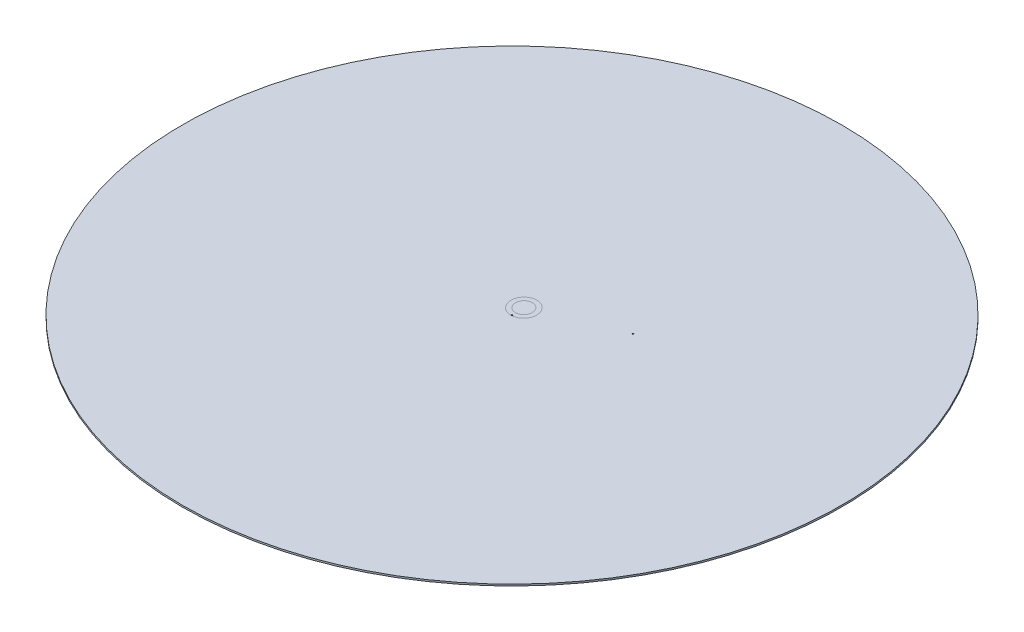
SolidWorks part; units mm, degrees
ref_plane "Front Plane" through (0, 0, 0) normal (0, 0, 1) x (1, 0, 0)
ref_plane "Top Plane" through (0, 0, 0) normal (0, 1, 0) x (1, 0, 0)
ref_plane "Right Plane" through (0, 0, 0) normal (1, 0, 0) x (0, 0, -1)
sketch "Sketch2" plane through (0, 0, 0) normal (0, 1, 0) x (1, 0, 0)
  circle A0 centre (0, 0) radius 40
  dimension "D1" = 80
extrude "Boss-Extrude1" add sketch "Sketch2" along normal blind 0.2
sketch "formula" plane through (0, 0.2, 0) normal (0, 1, 0) x (1, 0, 0)
  line L0 (0, 0) -> (0, 10.75) construction
  line L2 (46.374, 0) -> (0, 0) construction
  line L3 (9.3098, 5.375) -> (0, 0) construction
  line L4 (9.3098, 5.375) -> (0, 10.75) construction
  circle A16 centre (0, 10.75) radius 0.075
  circle A51 centre (9.3098, 16.125) radius 0.075
  circle A52 centre (0, 21.5) radius 0.075
  circle A53 centre (9.3098, 26.875) radius 0.075
  circle A54 centre (0, 32.25) radius 0.075
  circle A55 centre (9.3098, 37.625) radius 0.075
  circle A66 centre (0, 0) radius 0.075
  circle A67 centre (9.3098, 5.375) radius 0.075
  dimension "D2" = 0.15
  dimension "D3" = 10.75
sketch "Sketch4" plane through (0, 0.2, 0) normal (0, 1, 0) x (1, 0, 0)
  circle A1 centre (37.24, -10.75) radius 0.075
  circle A3 centre (18.62, -32.25) radius 0.075
  circle A5 centre (18.62, -10.75) radius 0.075
  circle A7 centre (27.9298, -16.125) radius 0.075
  circle A9 centre (18.62, -21.5) radius 0.075
  circle A11 centre (27.9298, -26.875) radius 0.075
  circle A13 centre (9.3098, -37.625) radius 0.075
  circle A15 centre (9.3098, -16.125) radius 0.075
  circle A17 centre (9.3098, -26.875) radius 0.075
  circle A19 centre (9.3098, -5.375) radius 0.075
  circle A21 centre (27.9298, -5.375) radius 0.075
  circle A23 centre (37.24, -10.75) radius 0.075
  circle A25 centre (18.62, -32.25) radius 0.075
  circle A27 centre (18.62, -10.75) radius 0.075
  circle A29 centre (27.9298, -16.125) radius 0.075
  circle A31 centre (18.62, -21.5) radius 0.075
  circle A33 centre (27.9298, -26.875) radius 0.075
  circle A35 centre (0, -32.25) radius 0.075
  circle A37 centre (9.3098, -37.625) radius 0.075
  circle A39 centre (0, -10.75) radius 0.075
  circle A41 centre (9.3098, -16.125) radius 0.075
  circle A43 centre (0, -21.5) radius 0.075
  circle A45 centre (9.3098, -26.875) radius 0.075
  circle A47 centre (9.3098, -5.375) radius 0.075
  circle A49 centre (27.9298, -5.375) radius 0.075
  circle A51 centre (-37.24, 10.75) radius 0.075
  circle A53 centre (-18.62, 32.25) radius 0.075
  circle A55 centre (-18.62, 10.75) radius 0.075
  circle A57 centre (-27.9298, 16.125) radius 0.075
  circle A59 centre (-18.62, 21.5) radius 0.075
  circle A61 centre (-27.9298, 26.875) radius 0.075
  circle A63 centre (-9.3098, 37.625) radius 0.075
  circle A65 centre (-9.3098, 16.125) radius 0.075
  circle A67 centre (-9.3098, 26.875) radius 0.075
  circle A69 centre (-9.3098, 5.375) radius 0.075
  circle A71 centre (-27.9298, 5.375) radius 0.075
  circle A73 centre (-37.24, 10.75) radius 0.075
  circle A75 centre (-37.24, 0) radius 0.075
  circle A77 centre (-18.62, 32.25) radius 0.075
  circle A79 centre (-18.62, 10.75) radius 0.075
  circle A81 centre (-27.9298, 16.125) radius 0.075
  circle A83 centre (-18.62, 21.5) radius 0.075
  circle A85 centre (-27.9298, 26.875) radius 0.075
  circle A87 centre (-18.62, 0) radius 0.075
  circle A89 centre (-9.3098, 37.625) radius 0.075
  circle A91 centre (-9.3098, 16.125) radius 0.075
  circle A93 centre (-9.3098, 26.875) radius 0.075
  circle A95 centre (-9.3098, 5.375) radius 0.075
  circle A97 centre (-27.9298, 5.375) radius 0.075
  circle A99 centre (-27.9298, -5.375) radius 0.075
  circle A101 centre (-9.3098, -5.375) radius 0.075
  circle A103 centre (-9.3098, -26.875) radius 0.075
  circle A105 centre (-9.3098, -16.125) radius 0.075
  circle A107 centre (-9.3098, -37.625) radius 0.075
  circle A109 centre (-27.9298, -26.875) radius 0.075
  circle A111 centre (-18.62, -21.5) radius 0.075
  circle A113 centre (-27.9298, -16.125) radius 0.075
  circle A115 centre (-18.62, -10.75) radius 0.075
  circle A117 centre (-18.62, -32.25) radius 0.075
  circle A119 centre (-37.24, -10.75) radius 0.075
  circle A121 centre (-27.9298, -5.375) radius 0.075
  circle A123 centre (-9.3098, -5.375) radius 0.075
  circle A125 centre (-9.3098, -26.875) radius 0.075
  circle A127 centre (-9.3098, -16.125) radius 0.075
  circle A129 centre (-9.3098, -37.625) radius 0.075
  circle A131 centre (-27.9298, -26.875) radius 0.075
  circle A133 centre (-18.62, -21.5) radius 0.075
  circle A135 centre (-27.9298, -16.125) radius 0.075
  circle A137 centre (-18.62, -10.75) radius 0.075
  circle A139 centre (-18.62, -32.25) radius 0.075
  circle A141 centre (-37.24, -10.75) radius 0.075
  circle A3000 centre (27.9298, 5.375) radius 0.075
  circle A3219 centre (9.3098, 5.375) radius 0.075
  circle A3220 centre (9.3098, 5.375) radius 0.075
  circle A3221 centre (0, 0) radius 0.075
  circle A3222 centre (0, 0) radius 0.075
  circle A3223 centre (9.3098, 26.875) radius 0.075
  circle A3224 centre (9.3098, 26.875) radius 0.075
  circle A3225 centre (0, 21.5) radius 0.075
  circle A3226 centre (0, 21.5) radius 0.075
  circle A3227 centre (9.3098, 16.125) radius 0.075
  circle A3228 centre (9.3098, 16.125) radius 0.075
  circle A3229 centre (0, 10.75) radius 0.075
  circle A3230 centre (0, 10.75) radius 0.075
  circle A3231 centre (9.3098, 37.625) radius 0.075
  circle A3232 centre (9.3098, 37.625) radius 0.075
  circle A3233 centre (0, 32.25) radius 0.075
  circle A3234 centre (0, 32.25) radius 0.075
  circle A3235 centre (18.62, 0) radius 0.075
  circle A3236 centre (27.9298, 26.875) radius 0.075
  circle A3237 centre (18.62, 21.5) radius 0.075
  circle A3238 centre (27.9298, 16.125) radius 0.075
  circle A3239 centre (18.62, 10.75) radius 0.075
  circle A3241 centre (18.62, 32.25) radius 0.075
  circle A3243 centre (37.24, 0) radius 0.075
  circle A3247 centre (37.24, 10.75) radius 0.075
  circle A3250 centre (27.9298, 37.625) radius 0.075
  circle A3251 centre (46.5498, 37.625) radius 0.075
  circle A3252 centre (37.24, 32.25) radius 0.075
  circle A3253 centre (46.5498, 26.875) radius 0.075
  circle A3254 centre (37.24, 21.5) radius 0.075
  circle A3255 centre (46.5498, 5.375) radius 0.075
  circle A3256 centre (46.5498, 16.125) radius 0.075
  circle A3271 centre (27.9298, 5.375) radius 0.075
  circle A3272 centre (9.3098, 5.375) radius 0.075
  circle A3273 centre (9.3098, 26.875) radius 0.075
  circle A3274 centre (9.3098, 16.125) radius 0.075
  circle A3275 centre (9.3098, 37.625) radius 0.075
  circle A3276 centre (27.9298, 26.875) radius 0.075
  circle A3277 centre (18.62, 21.5) radius 0.075
  circle A3278 centre (27.9298, 16.125) radius 0.075
  circle A3279 centre (18.62, 10.75) radius 0.075
  circle A3280 centre (18.62, 32.25) radius 0.075
  circle A3281 centre (37.24, 10.75) radius 0.075
  dimension "D121" = 0
  dimension "D122" = 0
  dimension "D123" = 0
  dimension "D124" = 0
  dimension "D125" = 0
  dimension "D126" = 0
  dimension "D127" = 0
  dimension "D128" = 0
  dimension "D129" = 3
extrude "Cut-Extrude2" cut sketch "Sketch4" against normal blind 0.2 contours A3222 | A3220 region at (0, 0.2, 0)
pattern_linear "LPattern1" [suppressed] count 4 spacing 10.75 along (0, 0, -1) count 3 spacing 18.6195 along (1, 0, 0) of bodies 157
mirror "Mirror1" [suppressed] about plane through (0, 0, 0) normal (1, 0, 0)
ref_plane "Plane1" through (0, 0, 0) normal (0, 0, -1) x (-1, 0, 0)
mirror "Mirror2" [suppressed] about plane through (0, 0, 0) normal (0, 0, -1)
sketch "numbers" plane through (0, 0.2, 0) normal (0, 1, 0) x (1, 0, 0)
  line L0 (-7.0476, 0) -> (7.0476, 0) construction
  line L1 (46.374, 0) -> (0, 0) construction
  text T0 "<b>O</b>" font "Century Gothic" height 3
  point P6 (0, 0)
split "Split1" trim tools "numbers" bodies to split 157 resulting bodies 162 164 165
sketch "Sketch5" plane through (0, 0.2, 0) normal (0, 1, 0) x (1, 0, 0)
  circle A1 centre (40.7032, 13.5) radius 0.075
  circle A2 centre (40.7032, 13.5) radius 0.075
  circle A3 centre (39.8372, 15) radius 0.075
  circle A4 centre (39.8372, 15) radius 0.075
  circle A5 centre (39.8372, 14) radius 0.075
  circle A6 centre (39.8372, 14) radius 0.075
  circle A7 centre (40.7032, 14.5) radius 0.075
  circle A8 centre (40.7032, 14.5) radius 0.075
  circle A9 centre (39.8372, 10) radius 0.075
  circle A10 centre (39.8372, 10) radius 0.075
  circle A11 centre (39.8372, 11) radius 0.075
  circle A12 centre (39.8372, 11) radius 0.075
  circle A13 centre (39.8372, 10) radius 0.075
  circle A14 centre (39.8372, 10) radius 0.075
  circle A15 centre (40.7032, 10.5) radius 0.075
  circle A16 centre (40.7032, 10.5) radius 0.075
  circle A17 centre (38.9711, 8.5) radius 0.075
  circle A18 centre (38.9711, 8.5) radius 0.075
  circle A19 centre (38.1051, 9) radius 0.075
  circle A20 centre (38.1051, 9) radius 0.075
  circle A21 centre (38.9711, 9.5) radius 0.075
  circle A22 centre (38.9711, 9.5) radius 0.075
  circle A23 centre (38.1051, 5) radius 0.075
  circle A24 centre (38.1051, 5) radius 0.075
  circle A25 centre (38.1051, 6) radius 0.075
  circle A26 centre (38.1051, 6) radius 0.075
  circle A27 centre (38.1051, 5) radius 0.075
  circle A28 centre (38.1051, 5) radius 0.075
  circle A29 centre (38.9711, 5.5) radius 0.075
  circle A30 centre (38.9711, 5.5) radius 0.075
  circle A31 centre (38.1051, 7) radius 0.075
  circle A32 centre (38.1051, 7) radius 0.075
  circle A33 centre (36.3731, 4) radius 0.075
  circle A34 centre (36.3731, 4) radius 0.075
  circle A35 centre (37.2391, 4.5) radius 0.075
  circle A36 centre (37.2391, 4.5) radius 0.075
  circle A37 centre (36.3731, 0) radius 0.075
  circle A38 centre (36.3731, 0) radius 0.075
  circle A39 centre (37.2391, 0.5) radius 0.075
  circle A40 centre (37.2391, 0.5) radius 0.075
  circle A41 centre (36.3731, 1) radius 0.075
  circle A42 centre (36.3731, 1) radius 0.075
  circle A43 centre (36.3731, 2) radius 0.075
  circle A44 centre (36.3731, 2) radius 0.075
  circle A45 centre (36.3731, 1) radius 0.075
  circle A46 centre (36.3731, 1) radius 0.075
  circle A47 centre (37.2391, 1.5) radius 0.075
  circle A48 centre (37.2391, 1.5) radius 0.075
  circle A71 centre (31.1769, 29) radius 0.075
  circle A72 centre (31.1769, 29) radius 0.075
  circle A73 centre (32.0429, 28.5) radius 0.075
  circle A74 centre (32.0429, 28.5) radius 0.075
  circle A75 centre (31.1769, 30) radius 0.075
  circle A76 centre (31.1769, 30) radius 0.075
  circle A77 centre (31.1769, 29) radius 0.075
  circle A78 centre (31.1769, 29) radius 0.075
  circle A79 centre (32.0429, 29.5) radius 0.075
  circle A80 centre (32.0429, 29.5) radius 0.075
  circle A81 centre (30.3109, 27.5) radius 0.075
  circle A82 centre (30.3109, 27.5) radius 0.075
  circle A83 centre (29.4449, 28) radius 0.075
  circle A84 centre (29.4449, 28) radius 0.075
  circle A85 centre (29.4449, 24) radius 0.075
  circle A86 centre (29.4449, 24) radius 0.075
  circle A87 centre (29.4449, 23) radius 0.075
  circle A88 centre (29.4449, 23) radius 0.075
  circle A89 centre (30.3109, 23.5) radius 0.075
  circle A90 centre (30.3109, 23.5) radius 0.075
  circle A91 centre (29.4449, 25) radius 0.075
  circle A92 centre (29.4449, 25) radius 0.075
  circle A93 centre (29.4449, 24) radius 0.075
  circle A94 centre (29.4449, 24) radius 0.075
  circle A95 centre (30.3109, 24.5) radius 0.075
  circle A96 centre (30.3109, 24.5) radius 0.075
  circle A97 centre (27.7128, 23) radius 0.075
  circle A98 centre (27.7128, 23) radius 0.075
  circle A99 centre (27.7128, 22) radius 0.075
  circle A100 centre (27.7128, 22) radius 0.075
  circle A101 centre (28.5788, 22.5) radius 0.075
  circle A102 centre (28.5788, 22.5) radius 0.075
  circle A103 centre (27.7128, 19) radius 0.075
  circle A104 centre (27.7128, 19) radius 0.075
  circle A105 centre (27.7128, 18) radius 0.075
  circle A106 centre (27.7128, 18) radius 0.075
  circle A107 centre (28.5788, 18.5) radius 0.075
  circle A108 centre (28.5788, 18.5) radius 0.075
  circle A109 centre (27.7128, 20) radius 0.075
  circle A110 centre (27.7128, 20) radius 0.075
  circle A111 centre (27.7128, 19) radius 0.075
  circle A112 centre (27.7128, 19) radius 0.075
  circle A113 centre (25.9808, 17) radius 0.075
  circle A114 centre (25.9808, 17) radius 0.075
  circle A115 centre (25.9808, 16) radius 0.075
  circle A116 centre (25.9808, 16) radius 0.075
  circle A117 centre (26.8468, 16.5) radius 0.075
  circle A118 centre (26.8468, 16.5) radius 0.075
  circle A119 centre (25.9808, 13) radius 0.075
  circle A120 centre (25.9808, 13) radius 0.075
  circle A121 centre (25.9808, 12) radius 0.075
  circle A122 centre (25.9808, 12) radius 0.075
  circle A123 centre (26.8468, 12.5) radius 0.075
  circle A124 centre (26.8468, 12.5) radius 0.075
  circle A125 centre (25.9808, 14) radius 0.075
  circle A126 centre (25.9808, 14) radius 0.075
  circle A127 centre (25.9808, 13) radius 0.075
  circle A128 centre (25.9808, 13) radius 0.075
  circle A129 centre (24.2487, 12) radius 0.075
  circle A130 centre (24.2487, 12) radius 0.075
  circle A131 centre (24.2487, 11) radius 0.075
  circle A132 centre (24.2487, 11) radius 0.075
  circle A133 centre (25.1147, 11.5) radius 0.075
  circle A134 centre (25.1147, 11.5) radius 0.075
  circle A135 centre (24.2487, 8) radius 0.075
  circle A136 centre (24.2487, 8) radius 0.075
  circle A137 centre (24.2487, 7) radius 0.075
  circle A138 centre (24.2487, 7) radius 0.075
  circle A139 centre (25.1147, 7.5) radius 0.075
  circle A140 centre (25.1147, 7.5) radius 0.075
  circle A141 centre (24.2487, 9) radius 0.075
  circle A142 centre (24.2487, 9) radius 0.075
  circle A143 centre (24.2487, 8) radius 0.075
  circle A144 centre (24.2487, 8) radius 0.075
  circle A145 centre (22.5167, 6) radius 0.075
  circle A146 centre (22.5167, 6) radius 0.075
  circle A147 centre (23.3827, 6.5) radius 0.075
  circle A148 centre (23.3827, 6.5) radius 0.075
  circle A149 centre (22.5167, 3) radius 0.075
  circle A150 centre (22.5167, 3) radius 0.075
  circle A151 centre (22.5167, 2) radius 0.075
  circle A152 centre (22.5167, 2) radius 0.075
  circle A153 centre (23.3827, 2.5) radius 0.075
  circle A154 centre (23.3827, 2.5) radius 0.075
  circle A155 centre (22.5167, 4) radius 0.075
  circle A156 centre (22.5167, 4) radius 0.075
  circle A157 centre (22.5167, 3) radius 0.075
  circle A158 centre (22.5167, 3) radius 0.075
  circle A159 centre (23.3827, 3.5) radius 0.075
  circle A160 centre (23.3827, 3.5) radius 0.075
  circle A177 centre (18.1865, 35.5) radius 0.075
  circle A178 centre (18.1865, 35.5) radius 0.075
  circle A179 centre (17.3205, 36) radius 0.075
  circle A180 centre (17.3205, 36) radius 0.075
  circle A181 centre (17.3205, 32) radius 0.075
  circle A182 centre (17.3205, 32) radius 0.075
  circle A183 centre (17.3205, 31) radius 0.075
  circle A184 centre (17.3205, 31) radius 0.075
  circle A185 centre (18.1865, 31.5) radius 0.075
  circle A186 centre (18.1865, 31.5) radius 0.075
  circle A187 centre (17.3205, 33) radius 0.075
  circle A188 centre (17.3205, 33) radius 0.075
  circle A189 centre (17.3205, 32) radius 0.075
  circle A190 centre (17.3205, 32) radius 0.075
  circle A191 centre (18.1865, 32.5) radius 0.075
  circle A192 centre (18.1865, 32.5) radius 0.075
  circle A193 centre (15.5885, 31) radius 0.075
  circle A194 centre (15.5885, 31) radius 0.075
  circle A195 centre (15.5885, 30) radius 0.075
  circle A196 centre (15.5885, 30) radius 0.075
  circle A197 centre (16.4545, 30.5) radius 0.075
  circle A198 centre (16.4545, 30.5) radius 0.075
  circle A199 centre (15.5885, 27) radius 0.075
  circle A200 centre (15.5885, 27) radius 0.075
  circle A201 centre (15.5885, 26) radius 0.075
  circle A202 centre (15.5885, 26) radius 0.075
  circle A203 centre (16.4545, 26.5) radius 0.075
  circle A204 centre (16.4545, 26.5) radius 0.075
  circle A205 centre (15.5885, 28) radius 0.075
  circle A206 centre (15.5885, 28) radius 0.075
  circle A207 centre (15.5885, 27) radius 0.075
  circle A208 centre (15.5885, 27) radius 0.075
  circle A209 centre (13.8564, 26) radius 0.075
  circle A210 centre (13.8564, 26) radius 0.075
  circle A211 centre (13.8564, 25) radius 0.075
  circle A212 centre (13.8564, 25) radius 0.075
  circle A213 centre (14.7224, 25.5) radius 0.075
  circle A214 centre (14.7224, 25.5) radius 0.075
  circle A215 centre (13.8564, 21) radius 0.075
  circle A216 centre (13.8564, 21) radius 0.075
  circle A217 centre (14.7224, 20.5) radius 0.075
  circle A218 centre (14.7224, 20.5) radius 0.075
  circle A219 centre (13.8564, 22) radius 0.075
  circle A220 centre (13.8564, 22) radius 0.075
  circle A221 centre (13.8564, 21) radius 0.075
  circle A222 centre (13.8564, 21) radius 0.075
  circle A223 centre (14.7224, 21.5) radius 0.075
  circle A224 centre (14.7224, 21.5) radius 0.075
  circle A225 centre (12.9904, 19.5) radius 0.075
  circle A226 centre (12.9904, 19.5) radius 0.075
  circle A227 centre (12.1244, 20) radius 0.075
  circle A228 centre (12.1244, 20) radius 0.075
  circle A229 centre (12.1244, 18) radius 0.075
  circle A230 centre (12.1244, 18) radius 0.075
  circle A231 centre (12.1244, 17) radius 0.075
  circle A232 centre (12.1244, 17) radius 0.075
  circle A233 centre (12.9904, 17.5) radius 0.075
  circle A234 centre (12.9904, 17.5) radius 0.075
  circle A235 centre (12.1244, 16) radius 0.075
  circle A236 centre (12.1244, 16) radius 0.075
  circle A237 centre (12.1244, 15) radius 0.075
  circle A238 centre (12.1244, 15) radius 0.075
  circle A239 centre (12.9904, 15.5) radius 0.075
  circle A240 centre (12.9904, 15.5) radius 0.075
  circle A241 centre (11.2583, 13.5) radius 0.075
  circle A242 centre (11.2583, 13.5) radius 0.075
  circle A243 centre (10.3923, 15) radius 0.075
  circle A244 centre (10.3923, 15) radius 0.075
  circle A245 centre (10.3923, 14) radius 0.075
  circle A246 centre (10.3923, 14) radius 0.075
  circle A247 centre (11.2583, 14.5) radius 0.075
  circle A248 centre (11.2583, 14.5) radius 0.075
  circle A249 centre (10.3923, 10) radius 0.075
  circle A250 centre (10.3923, 10) radius 0.075
  circle A251 centre (10.3923, 11) radius 0.075
  circle A252 centre (10.3923, 11) radius 0.075
  circle A253 centre (10.3923, 10) radius 0.075
  circle A254 centre (10.3923, 10) radius 0.075
  circle A255 centre (11.2583, 10.5) radius 0.075
  circle A256 centre (11.2583, 10.5) radius 0.075
  circle A257 centre (9.5263, 8.5) radius 0.075
  circle A258 centre (9.5263, 8.5) radius 0.075
  circle A259 centre (8.6603, 9) radius 0.075
  circle A260 centre (8.6603, 9) radius 0.075
  circle A261 centre (9.5263, 9.5) radius 0.075
  circle A262 centre (9.5263, 9.5) radius 0.075
  circle A263 centre (8.6603, 5) radius 0.075
  circle A264 centre (8.6603, 5) radius 0.075
  circle A265 centre (8.6603, 6) radius 0.075
  circle A266 centre (8.6603, 6) radius 0.075
  circle A267 centre (8.6603, 5) radius 0.075
  circle A268 centre (8.6603, 5) radius 0.075
  circle A269 centre (9.5263, 5.5) radius 0.075
  circle A270 centre (9.5263, 5.5) radius 0.075
  circle A271 centre (8.6603, 7) radius 0.075
  circle A272 centre (8.6603, 7) radius 0.075
  circle A273 centre (6.9282, 4) radius 0.075
  circle A274 centre (6.9282, 4) radius 0.075
  circle A275 centre (7.7942, 4.5) radius 0.075
  circle A276 centre (7.7942, 4.5) radius 0.075
  circle A277 centre (6.9282, 0) radius 0.075
  circle A278 centre (6.9282, 0) radius 0.075
  circle A279 centre (7.7942, 0.5) radius 0.075
  circle A280 centre (7.7942, 0.5) radius 0.075
  circle A281 centre (6.9282, 1) radius 0.075
  circle A282 centre (6.9282, 1) radius 0.075
  circle A283 centre (6.9282, 2) radius 0.075
  circle A284 centre (6.9282, 2) radius 0.075
  circle A285 centre (6.9282, 1) radius 0.075
  circle A286 centre (6.9282, 1) radius 0.075
  circle A287 centre (7.7942, 1.5) radius 0.075
  circle A288 centre (7.7942, 1.5) radius 0.075
  circle A289 centre (3.4641, 39) radius 0.075
  circle A290 centre (3.4641, 39) radius 0.075
  circle A291 centre (3.4641, 38) radius 0.075
  circle A292 centre (3.4641, 38) radius 0.075
  circle A293 centre (4.3301, 38.5) radius 0.075
  circle A294 centre (4.3301, 38.5) radius 0.075
  circle A295 centre (3.4641, 35) radius 0.075
  circle A296 centre (3.4641, 35) radius 0.075
  circle A297 centre (3.4641, 34) radius 0.075
  circle A298 centre (3.4641, 34) radius 0.075
  circle A299 centre (4.3301, 34.5) radius 0.075
  circle A300 centre (4.3301, 34.5) radius 0.075
  circle A301 centre (3.4641, 36) radius 0.075
  circle A302 centre (3.4641, 36) radius 0.075
  circle A303 centre (3.4641, 35) radius 0.075
  circle A304 centre (3.4641, 35) radius 0.075
  circle A305 centre (1.7321, 34) radius 0.075
  circle A306 centre (1.7321, 34) radius 0.075
  circle A307 centre (1.7321, 33) radius 0.075
  circle A308 centre (1.7321, 33) radius 0.075
  circle A309 centre (2.5981, 33.5) radius 0.075
  circle A310 centre (2.5981, 33.5) radius 0.075
  circle A311 centre (1.7321, 29) radius 0.075
  circle A312 centre (1.7321, 29) radius 0.075
  circle A313 centre (2.5981, 28.5) radius 0.075
  circle A314 centre (2.5981, 28.5) radius 0.075
  circle A315 centre (1.7321, 30) radius 0.075
  circle A316 centre (1.7321, 30) radius 0.075
  circle A317 centre (1.7321, 29) radius 0.075
  circle A318 centre (1.7321, 29) radius 0.075
  circle A319 centre (2.5981, 29.5) radius 0.075
  circle A320 centre (2.5981, 29.5) radius 0.075
  circle A321 centre (0.866, 28.5) radius 0.075
  circle A322 centre (0.866, 28.5) radius 0.075
  circle A323 centre (0, 30) radius 0.075
  circle A324 centre (0, 30) radius 0.075
  circle A325 centre (0, 29) radius 0.075
  circle A326 centre (0, 29) radius 0.075
  circle A327 centre (0.866, 29.5) radius 0.075
  circle A328 centre (0.866, 29.5) radius 0.075
  circle A329 centre (0, 31) radius 0.075
  circle A330 centre (0, 31) radius 0.075
  circle A331 centre (0.866, 1.5) radius 0.075
  circle A332 centre (0.866, 1.5) radius 0.075
  circle A335 centre (0, 39) radius 0.075
  circle A336 centre (0, 39) radius 0.075
  circle A337 centre (0.866, 39.5) radius 0.075
  circle A338 centre (0.866, 39.5) radius 0.075
  circle A339 centre (39.8372, 17) radius 0.075
  circle A340 centre (39.8372, 17) radius 0.075
  circle A341 centre (39.8372, 16) radius 0.075
  circle A342 centre (39.8372, 16) radius 0.075
  circle A343 centre (40.7032, 16.5) radius 0.075
  circle A344 centre (40.7032, 16.5) radius 0.075
  circle A345 centre (39.8372, 13) radius 0.075
  circle A346 centre (39.8372, 13) radius 0.075
  circle A347 centre (39.8372, 12) radius 0.075
  circle A348 centre (39.8372, 12) radius 0.075
  circle A349 centre (40.7032, 12.5) radius 0.075
  circle A350 centre (40.7032, 12.5) radius 0.075
  circle A351 centre (39.8372, 14) radius 0.075
  circle A352 centre (39.8372, 14) radius 0.075
  circle A353 centre (39.8372, 13) radius 0.075
  circle A354 centre (39.8372, 13) radius 0.075
  circle A355 centre (38.1051, 12) radius 0.075
  circle A356 centre (38.1051, 12) radius 0.075
  circle A357 centre (38.1051, 11) radius 0.075
  circle A358 centre (38.1051, 11) radius 0.075
  circle A359 centre (38.9711, 11.5) radius 0.075
  circle A360 centre (38.9711, 11.5) radius 0.075
  circle A361 centre (38.1051, 8) radius 0.075
  circle A362 centre (38.1051, 8) radius 0.075
  circle A363 centre (38.1051, 7) radius 0.075
  circle A364 centre (38.1051, 7) radius 0.075
  circle A365 centre (38.9711, 7.5) radius 0.075
  circle A366 centre (38.9711, 7.5) radius 0.075
  circle A367 centre (38.1051, 9) radius 0.075
  circle A368 centre (38.1051, 9) radius 0.075
  circle A369 centre (38.1051, 8) radius 0.075
  circle A370 centre (38.1051, 8) radius 0.075
  circle A371 centre (36.3731, 6) radius 0.075
  circle A372 centre (36.3731, 6) radius 0.075
  circle A373 centre (37.2391, 6.5) radius 0.075
  circle A374 centre (37.2391, 6.5) radius 0.075
  circle A375 centre (36.3731, 3) radius 0.075
  circle A376 centre (36.3731, 3) radius 0.075
  circle A377 centre (36.3731, 2) radius 0.075
  circle A378 centre (36.3731, 2) radius 0.075
  circle A379 centre (37.2391, 2.5) radius 0.075
  circle A380 centre (37.2391, 2.5) radius 0.075
  circle A381 centre (36.3731, 4) radius 0.075
  circle A382 centre (36.3731, 4) radius 0.075
  circle A383 centre (36.3731, 3) radius 0.075
  circle A384 centre (36.3731, 3) radius 0.075
  circle A385 centre (37.2391, 3.5) radius 0.075
  circle A386 centre (37.2391, 3.5) radius 0.075
  circle A407 centre (31.1769, 32) radius 0.075
  circle A408 centre (31.1769, 32) radius 0.075
  circle A409 centre (31.1769, 31) radius 0.075
  circle A410 centre (31.1769, 31) radius 0.075
  circle A411 centre (32.0429, 31.5) radius 0.075
  circle A412 centre (32.0429, 31.5) radius 0.075
  circle A415 centre (31.1769, 32) radius 0.075
  circle A416 centre (31.1769, 32) radius 0.075
  circle A417 centre (32.0429, 32.5) radius 0.075
  circle A418 centre (32.0429, 32.5) radius 0.075
  circle A419 centre (29.4449, 31) radius 0.075
  circle A420 centre (29.4449, 31) radius 0.075
  circle A421 centre (29.4449, 30) radius 0.075
  circle A422 centre (29.4449, 30) radius 0.075
  circle A423 centre (30.3109, 30.5) radius 0.075
  circle A424 centre (30.3109, 30.5) radius 0.075
  circle A425 centre (29.4449, 27) radius 0.075
  circle A426 centre (29.4449, 27) radius 0.075
  circle A427 centre (29.4449, 26) radius 0.075
  circle A428 centre (29.4449, 26) radius 0.075
  circle A429 centre (30.3109, 26.5) radius 0.075
  circle A430 centre (30.3109, 26.5) radius 0.075
  circle A431 centre (29.4449, 28) radius 0.075
  circle A432 centre (29.4449, 28) radius 0.075
  circle A433 centre (29.4449, 27) radius 0.075
  circle A434 centre (29.4449, 27) radius 0.075
  circle A435 centre (27.7128, 26) radius 0.075
  circle A436 centre (27.7128, 26) radius 0.075
  circle A437 centre (27.7128, 25) radius 0.075
  circle A438 centre (27.7128, 25) radius 0.075
  circle A439 centre (28.5788, 25.5) radius 0.075
  circle A440 centre (28.5788, 25.5) radius 0.075
  circle A441 centre (27.7128, 21) radius 0.075
  circle A442 centre (27.7128, 21) radius 0.075
  circle A443 centre (28.5788, 20.5) radius 0.075
  circle A444 centre (28.5788, 20.5) radius 0.075
  circle A445 centre (27.7128, 22) radius 0.075
  circle A446 centre (27.7128, 22) radius 0.075
  circle A447 centre (27.7128, 21) radius 0.075
  circle A448 centre (27.7128, 21) radius 0.075
  circle A449 centre (28.5788, 21.5) radius 0.075
  circle A450 centre (28.5788, 21.5) radius 0.075
  circle A451 centre (26.8468, 19.5) radius 0.075
  circle A452 centre (26.8468, 19.5) radius 0.075
  circle A453 centre (25.9808, 20) radius 0.075
  circle A454 centre (25.9808, 20) radius 0.075
  circle A455 centre (25.9808, 18) radius 0.075
  circle A456 centre (25.9808, 18) radius 0.075
  circle A457 centre (25.9808, 17) radius 0.075
  circle A458 centre (25.9808, 17) radius 0.075
  circle A459 centre (26.8468, 17.5) radius 0.075
  circle A460 centre (26.8468, 17.5) radius 0.075
  circle A461 centre (25.9808, 16) radius 0.075
  circle A462 centre (25.9808, 16) radius 0.075
  circle A463 centre (25.9808, 15) radius 0.075
  circle A464 centre (25.9808, 15) radius 0.075
  circle A465 centre (26.8468, 15.5) radius 0.075
  circle A466 centre (26.8468, 15.5) radius 0.075
  circle A467 centre (25.1147, 13.5) radius 0.075
  circle A468 centre (25.1147, 13.5) radius 0.075
  circle A469 centre (24.2487, 15) radius 0.075
  circle A470 centre (24.2487, 15) radius 0.075
  circle A471 centre (24.2487, 14) radius 0.075
  circle A472 centre (24.2487, 14) radius 0.075
  circle A473 centre (25.1147, 14.5) radius 0.075
  circle A474 centre (25.1147, 14.5) radius 0.075
  circle A475 centre (24.2487, 10) radius 0.075
  circle A476 centre (24.2487, 10) radius 0.075
  circle A477 centre (24.2487, 11) radius 0.075
  circle A478 centre (24.2487, 11) radius 0.075
  circle A479 centre (24.2487, 10) radius 0.075
  circle A480 centre (24.2487, 10) radius 0.075
  circle A481 centre (25.1147, 10.5) radius 0.075
  circle A482 centre (25.1147, 10.5) radius 0.075
  circle A483 centre (23.3827, 8.5) radius 0.075
  circle A484 centre (23.3827, 8.5) radius 0.075
  circle A485 centre (22.5167, 9) radius 0.075
  circle A486 centre (22.5167, 9) radius 0.075
  circle A487 centre (23.3827, 9.5) radius 0.075
  circle A488 centre (23.3827, 9.5) radius 0.075
  circle A489 centre (22.5167, 5) radius 0.075
  circle A490 centre (22.5167, 5) radius 0.075
  circle A491 centre (22.5167, 6) radius 0.075
  circle A492 centre (22.5167, 6) radius 0.075
  circle A493 centre (22.5167, 5) radius 0.075
  circle A494 centre (22.5167, 5) radius 0.075
  circle A495 centre (23.3827, 5.5) radius 0.075
  circle A496 centre (23.3827, 5.5) radius 0.075
  circle A497 centre (22.5167, 7) radius 0.075
  circle A498 centre (22.5167, 7) radius 0.075
  circle A499 centre (20.7846, 4) radius 0.075
  circle A500 centre (20.7846, 4) radius 0.075
  circle A501 centre (21.6506, 4.5) radius 0.075
  circle A502 centre (21.6506, 4.5) radius 0.075
  circle A503 centre (20.7846, 0) radius 0.075
  circle A504 centre (20.7846, 0) radius 0.075
  circle A505 centre (21.6506, 0.5) radius 0.075
  circle A506 centre (21.6506, 0.5) radius 0.075
  circle A507 centre (20.7846, 1) radius 0.075
  circle A508 centre (20.7846, 1) radius 0.075
  circle A509 centre (20.7846, 2) radius 0.075
  circle A510 centre (20.7846, 2) radius 0.075
  circle A511 centre (20.7846, 1) radius 0.075
  circle A512 centre (20.7846, 1) radius 0.075
  circle A513 centre (21.6506, 1.5) radius 0.075
  circle A514 centre (21.6506, 1.5) radius 0.075
  circle A515 centre (17.3205, 39) radius 0.075
  circle A516 centre (17.3205, 39) radius 0.075
  circle A517 centre (17.3205, 38) radius 0.075
  circle A518 centre (17.3205, 38) radius 0.075
  circle A521 centre (17.3205, 35) radius 0.075
  circle A522 centre (17.3205, 35) radius 0.075
  circle A523 centre (17.3205, 34) radius 0.075
  circle A524 centre (17.3205, 34) radius 0.075
  circle A525 centre (18.1865, 34.5) radius 0.075
  circle A526 centre (18.1865, 34.5) radius 0.075
  circle A527 centre (17.3205, 36) radius 0.075
  circle A528 centre (17.3205, 36) radius 0.075
  circle A529 centre (17.3205, 35) radius 0.075
  circle A530 centre (17.3205, 35) radius 0.075
  circle A531 centre (15.5885, 34) radius 0.075
  circle A532 centre (15.5885, 34) radius 0.075
  circle A533 centre (15.5885, 33) radius 0.075
  circle A534 centre (15.5885, 33) radius 0.075
  circle A535 centre (16.4545, 33.5) radius 0.075
  circle A536 centre (16.4545, 33.5) radius 0.075
  circle A537 centre (15.5885, 29) radius 0.075
  circle A538 centre (15.5885, 29) radius 0.075
  circle A539 centre (16.4545, 28.5) radius 0.075
  circle A540 centre (16.4545, 28.5) radius 0.075
  circle A541 centre (15.5885, 30) radius 0.075
  circle A542 centre (15.5885, 30) radius 0.075
  circle A543 centre (15.5885, 29) radius 0.075
  circle A544 centre (15.5885, 29) radius 0.075
  circle A545 centre (16.4545, 29.5) radius 0.075
  circle A546 centre (16.4545, 29.5) radius 0.075
  circle A547 centre (14.7224, 27.5) radius 0.075
  circle A548 centre (14.7224, 27.5) radius 0.075
  circle A549 centre (13.8564, 28) radius 0.075
  circle A550 centre (13.8564, 28) radius 0.075
  circle A551 centre (13.8564, 24) radius 0.075
  circle A552 centre (13.8564, 24) radius 0.075
  circle A553 centre (13.8564, 23) radius 0.075
  circle A554 centre (13.8564, 23) radius 0.075
  circle A555 centre (14.7224, 23.5) radius 0.075
  circle A556 centre (14.7224, 23.5) radius 0.075
  circle A557 centre (13.8564, 25) radius 0.075
  circle A558 centre (13.8564, 25) radius 0.075
  circle A559 centre (13.8564, 24) radius 0.075
  circle A560 centre (13.8564, 24) radius 0.075
  circle A561 centre (14.7224, 24.5) radius 0.075
  circle A562 centre (14.7224, 24.5) radius 0.075
  circle A563 centre (12.1244, 23) radius 0.075
  circle A564 centre (12.1244, 23) radius 0.075
  circle A565 centre (12.1244, 22) radius 0.075
  circle A566 centre (12.1244, 22) radius 0.075
  circle A567 centre (12.9904, 22.5) radius 0.075
  circle A568 centre (12.9904, 22.5) radius 0.075
  circle A569 centre (12.1244, 19) radius 0.075
  circle A570 centre (12.1244, 19) radius 0.075
  circle A571 centre (12.1244, 18) radius 0.075
  circle A572 centre (12.1244, 18) radius 0.075
  circle A573 centre (12.9904, 18.5) radius 0.075
  circle A574 centre (12.9904, 18.5) radius 0.075
  circle A575 centre (12.1244, 20) radius 0.075
  circle A576 centre (12.1244, 20) radius 0.075
  circle A577 centre (12.1244, 19) radius 0.075
  circle A578 centre (12.1244, 19) radius 0.075
  circle A579 centre (10.3923, 17) radius 0.075
  circle A580 centre (10.3923, 17) radius 0.075
  circle A581 centre (10.3923, 16) radius 0.075
  circle A582 centre (10.3923, 16) radius 0.075
  circle A583 centre (11.2583, 16.5) radius 0.075
  circle A584 centre (11.2583, 16.5) radius 0.075
  circle A585 centre (10.3923, 13) radius 0.075
  circle A586 centre (10.3923, 13) radius 0.075
  circle A587 centre (10.3923, 12) radius 0.075
  circle A588 centre (10.3923, 12) radius 0.075
  circle A589 centre (11.2583, 12.5) radius 0.075
  circle A590 centre (11.2583, 12.5) radius 0.075
  circle A591 centre (10.3923, 14) radius 0.075
  circle A592 centre (10.3923, 14) radius 0.075
  circle A593 centre (10.3923, 13) radius 0.075
  circle A594 centre (10.3923, 13) radius 0.075
  circle A595 centre (8.6603, 12) radius 0.075
  circle A596 centre (8.6603, 12) radius 0.075
  circle A597 centre (8.6603, 11) radius 0.075
  circle A598 centre (8.6603, 11) radius 0.075
  circle A599 centre (9.5263, 11.5) radius 0.075
  circle A600 centre (9.5263, 11.5) radius 0.075
  circle A601 centre (8.6603, 8) radius 0.075
  circle A602 centre (8.6603, 8) radius 0.075
  circle A603 centre (8.6603, 7) radius 0.075
  circle A604 centre (8.6603, 7) radius 0.075
  circle A605 centre (9.5263, 7.5) radius 0.075
  circle A606 centre (9.5263, 7.5) radius 0.075
  circle A607 centre (8.6603, 9) radius 0.075
  circle A608 centre (8.6603, 9) radius 0.075
  circle A609 centre (8.6603, 8) radius 0.075
  circle A610 centre (8.6603, 8) radius 0.075
  circle A611 centre (6.9282, 6) radius 0.075
  circle A612 centre (6.9282, 6) radius 0.075
  circle A613 centre (7.7942, 6.5) radius 0.075
  circle A614 centre (7.7942, 6.5) radius 0.075
  circle A615 centre (6.9282, 3) radius 0.075
  circle A616 centre (6.9282, 3) radius 0.075
  circle A617 centre (6.9282, 2) radius 0.075
  circle A618 centre (6.9282, 2) radius 0.075
  circle A619 centre (7.7942, 2.5) radius 0.075
  circle A620 centre (7.7942, 2.5) radius 0.075
  circle A621 centre (6.9282, 4) radius 0.075
  circle A622 centre (6.9282, 4) radius 0.075
  circle A623 centre (6.9282, 3) radius 0.075
  circle A624 centre (6.9282, 3) radius 0.075
  circle A625 centre (7.7942, 3.5) radius 0.075
  circle A626 centre (7.7942, 3.5) radius 0.075
  circle A629 centre (5.1962, 39) radius 0.075
  circle A630 centre (5.1962, 39) radius 0.075
  circle A633 centre (3.4641, 37) radius 0.075
  circle A634 centre (3.4641, 37) radius 0.075
  circle A635 centre (4.3301, 36.5) radius 0.075
  circle A636 centre (4.3301, 36.5) radius 0.075
  circle A637 centre (3.4641, 38) radius 0.075
  circle A638 centre (3.4641, 38) radius 0.075
  circle A639 centre (3.4641, 37) radius 0.075
  circle A640 centre (3.4641, 37) radius 0.075
  circle A641 centre (4.3301, 37.5) radius 0.075
  circle A642 centre (4.3301, 37.5) radius 0.075
  circle A643 centre (2.5981, 35.5) radius 0.075
  circle A644 centre (2.5981, 35.5) radius 0.075
  circle A645 centre (1.7321, 36) radius 0.075
  circle A646 centre (1.7321, 36) radius 0.075
  circle A647 centre (1.7321, 32) radius 0.075
  circle A648 centre (1.7321, 32) radius 0.075
  circle A649 centre (1.7321, 31) radius 0.075
  circle A650 centre (1.7321, 31) radius 0.075
  circle A651 centre (2.5981, 31.5) radius 0.075
  circle A652 centre (2.5981, 31.5) radius 0.075
  circle A653 centre (1.7321, 33) radius 0.075
  circle A654 centre (1.7321, 33) radius 0.075
  circle A655 centre (1.7321, 32) radius 0.075
  circle A656 centre (1.7321, 32) radius 0.075
  circle A657 centre (2.5981, 32.5) radius 0.075
  circle A658 centre (2.5981, 32.5) radius 0.075
  circle A659 centre (0.866, 32.5) radius 0.075
  circle A660 centre (0.866, 32.5) radius 0.075
  circle A661 centre (0, 34) radius 0.075
  circle A662 centre (0, 34) radius 0.075
  circle A663 centre (0, 33) radius 0.075
  circle A664 centre (0, 33) radius 0.075
  circle A665 centre (0.866, 33.5) radius 0.075
  circle A666 centre (0.866, 33.5) radius 0.075
  circle A667 centre (0, 29) radius 0.075
  circle A668 centre (0, 29) radius 0.075
  circle A669 centre (0.866, 4.5) radius 0.075
  circle A670 centre (0.866, 4.5) radius 0.075
  circle A671 centre (0, 0) radius 0.075
  circle A672 centre (0, 0) radius 0.075
  circle A673 centre (0.866, 0.5) radius 0.075
  circle A674 centre (0.866, 0.5) radius 0.075
  circle A675 centre (0, 1) radius 0.075
  circle A676 centre (0, 1) radius 0.075
  circle A677 centre (0, 2) radius 0.075
  circle A678 centre (0, 2) radius 0.075
  circle A679 centre (0, 1) radius 0.075
  circle A680 centre (0, 1) radius 0.075
  circle A681 centre (40.7032, 19.5) radius 0.075
  circle A682 centre (40.7032, 19.5) radius 0.075
  circle A683 centre (39.8372, 20) radius 0.075
  circle A684 centre (39.8372, 20) radius 0.075
  circle A685 centre (39.8372, 18) radius 0.075
  circle A686 centre (39.8372, 18) radius 0.075
  circle A687 centre (39.8372, 17) radius 0.075
  circle A688 centre (39.8372, 17) radius 0.075
  circle A689 centre (40.7032, 17.5) radius 0.075
  circle A690 centre (40.7032, 17.5) radius 0.075
  circle A691 centre (39.8372, 16) radius 0.075
  circle A692 centre (39.8372, 16) radius 0.075
  circle A693 centre (39.8372, 15) radius 0.075
  circle A694 centre (39.8372, 15) radius 0.075
  circle A695 centre (40.7032, 15.5) radius 0.075
  circle A696 centre (40.7032, 15.5) radius 0.075
  circle A697 centre (38.9711, 13.5) radius 0.075
  circle A698 centre (38.9711, 13.5) radius 0.075
  circle A699 centre (38.1051, 15) radius 0.075
  circle A700 centre (38.1051, 15) radius 0.075
  circle A701 centre (38.1051, 14) radius 0.075
  circle A702 centre (38.1051, 14) radius 0.075
  circle A703 centre (38.9711, 14.5) radius 0.075
  circle A704 centre (38.9711, 14.5) radius 0.075
  circle A705 centre (38.1051, 10) radius 0.075
  circle A706 centre (38.1051, 10) radius 0.075
  circle A707 centre (38.1051, 11) radius 0.075
  circle A708 centre (38.1051, 11) radius 0.075
  circle A709 centre (38.1051, 10) radius 0.075
  circle A710 centre (38.1051, 10) radius 0.075
  circle A711 centre (38.9711, 10.5) radius 0.075
  circle A712 centre (38.9711, 10.5) radius 0.075
  circle A713 centre (37.2391, 8.5) radius 0.075
  circle A714 centre (37.2391, 8.5) radius 0.075
  circle A715 centre (36.3731, 9) radius 0.075
  circle A716 centre (36.3731, 9) radius 0.075
  circle A717 centre (37.2391, 9.5) radius 0.075
  circle A718 centre (37.2391, 9.5) radius 0.075
  circle A719 centre (36.3731, 5) radius 0.075
  circle A720 centre (36.3731, 5) radius 0.075
  circle A721 centre (36.3731, 6) radius 0.075
  circle A722 centre (36.3731, 6) radius 0.075
  circle A723 centre (36.3731, 5) radius 0.075
  circle A724 centre (36.3731, 5) radius 0.075
  circle A725 centre (37.2391, 5.5) radius 0.075
  circle A726 centre (37.2391, 5.5) radius 0.075
  circle A727 centre (36.3731, 7) radius 0.075
  circle A728 centre (36.3731, 7) radius 0.075
  circle A729 centre (34.641, 4) radius 0.075
  circle A730 centre (34.641, 4) radius 0.075
  circle A731 centre (35.507, 4.5) radius 0.075
  circle A732 centre (35.507, 4.5) radius 0.075
  circle A733 centre (34.641, 0) radius 0.075
  circle A734 centre (34.641, 0) radius 0.075
  circle A735 centre (35.507, 0.5) radius 0.075
  circle A736 centre (35.507, 0.5) radius 0.075
  circle A737 centre (34.641, 1) radius 0.075
  circle A738 centre (34.641, 1) radius 0.075
  circle A739 centre (34.641, 2) radius 0.075
  circle A740 centre (34.641, 2) radius 0.075
  circle A741 centre (34.641, 1) radius 0.075
  circle A742 centre (34.641, 1) radius 0.075
  circle A743 centre (35.507, 1.5) radius 0.075
  circle A744 centre (35.507, 1.5) radius 0.075
  circle A767 centre (29.4449, 29) radius 0.075
  circle A768 centre (29.4449, 29) radius 0.075
  circle A769 centre (30.3109, 28.5) radius 0.075
  circle A770 centre (30.3109, 28.5) radius 0.075
  circle A771 centre (29.4449, 30) radius 0.075
  circle A772 centre (29.4449, 30) radius 0.075
  circle A773 centre (29.4449, 29) radius 0.075
  circle A774 centre (29.4449, 29) radius 0.075
  circle A775 centre (30.3109, 29.5) radius 0.075
  circle A776 centre (30.3109, 29.5) radius 0.075
  circle A777 centre (28.5788, 27.5) radius 0.075
  circle A778 centre (28.5788, 27.5) radius 0.075
  circle A779 centre (27.7128, 28) radius 0.075
  circle A780 centre (27.7128, 28) radius 0.075
  circle A781 centre (27.7128, 24) radius 0.075
  circle A782 centre (27.7128, 24) radius 0.075
  circle A783 centre (27.7128, 23) radius 0.075
  circle A784 centre (27.7128, 23) radius 0.075
  circle A785 centre (28.5788, 23.5) radius 0.075
  circle A786 centre (28.5788, 23.5) radius 0.075
  circle A787 centre (27.7128, 25) radius 0.075
  circle A788 centre (27.7128, 25) radius 0.075
  circle A789 centre (27.7128, 24) radius 0.075
  circle A790 centre (27.7128, 24) radius 0.075
  circle A791 centre (28.5788, 24.5) radius 0.075
  circle A792 centre (28.5788, 24.5) radius 0.075
  circle A793 centre (25.9808, 23) radius 0.075
  circle A794 centre (25.9808, 23) radius 0.075
  circle A795 centre (25.9808, 22) radius 0.075
  circle A796 centre (25.9808, 22) radius 0.075
  circle A797 centre (26.8468, 22.5) radius 0.075
  circle A798 centre (26.8468, 22.5) radius 0.075
  circle A799 centre (25.9808, 19) radius 0.075
  circle A800 centre (25.9808, 19) radius 0.075
  circle A801 centre (25.9808, 18) radius 0.075
  circle A802 centre (25.9808, 18) radius 0.075
  circle A803 centre (26.8468, 18.5) radius 0.075
  circle A804 centre (26.8468, 18.5) radius 0.075
  circle A805 centre (25.9808, 20) radius 0.075
  circle A806 centre (25.9808, 20) radius 0.075
  circle A807 centre (25.9808, 19) radius 0.075
  circle A808 centre (25.9808, 19) radius 0.075
  circle A809 centre (24.2487, 17) radius 0.075
  circle A810 centre (24.2487, 17) radius 0.075
  circle A811 centre (24.2487, 16) radius 0.075
  circle A812 centre (24.2487, 16) radius 0.075
  circle A813 centre (25.1147, 16.5) radius 0.075
  circle A814 centre (25.1147, 16.5) radius 0.075
  circle A815 centre (24.2487, 13) radius 0.075
  circle A816 centre (24.2487, 13) radius 0.075
  circle A817 centre (24.2487, 12) radius 0.075
  circle A818 centre (24.2487, 12) radius 0.075
  circle A819 centre (25.1147, 12.5) radius 0.075
  circle A820 centre (25.1147, 12.5) radius 0.075
  circle A821 centre (24.2487, 14) radius 0.075
  circle A822 centre (24.2487, 14) radius 0.075
  circle A823 centre (24.2487, 13) radius 0.075
  circle A824 centre (24.2487, 13) radius 0.075
  circle A825 centre (22.5167, 12) radius 0.075
  circle A826 centre (22.5167, 12) radius 0.075
  circle A827 centre (22.5167, 11) radius 0.075
  circle A828 centre (22.5167, 11) radius 0.075
  circle A829 centre (23.3827, 11.5) radius 0.075
  circle A830 centre (23.3827, 11.5) radius 0.075
  circle A831 centre (22.5167, 8) radius 0.075
  circle A832 centre (22.5167, 8) radius 0.075
  circle A833 centre (22.5167, 7) radius 0.075
  circle A834 centre (22.5167, 7) radius 0.075
  circle A835 centre (23.3827, 7.5) radius 0.075
  circle A836 centre (23.3827, 7.5) radius 0.075
  circle A837 centre (22.5167, 9) radius 0.075
  circle A838 centre (22.5167, 9) radius 0.075
  circle A839 centre (22.5167, 8) radius 0.075
  circle A840 centre (22.5167, 8) radius 0.075
  circle A841 centre (20.7846, 6) radius 0.075
  circle A842 centre (20.7846, 6) radius 0.075
  circle A843 centre (21.6506, 6.5) radius 0.075
  circle A844 centre (21.6506, 6.5) radius 0.075
  circle A845 centre (20.7846, 3) radius 0.075
  circle A846 centre (20.7846, 3) radius 0.075
  circle A847 centre (20.7846, 2) radius 0.075
  circle A848 centre (20.7846, 2) radius 0.075
  circle A849 centre (21.6506, 2.5) radius 0.075
  circle A850 centre (21.6506, 2.5) radius 0.075
  circle A851 centre (20.7846, 4) radius 0.075
  circle A852 centre (20.7846, 4) radius 0.075
  circle A853 centre (20.7846, 3) radius 0.075
  circle A854 centre (20.7846, 3) radius 0.075
  circle A855 centre (21.6506, 3.5) radius 0.075
  circle A856 centre (21.6506, 3.5) radius 0.075
  circle A863 centre (17.3205, 37) radius 0.075
  circle A864 centre (17.3205, 37) radius 0.075
  circle A867 centre (17.3205, 38) radius 0.075
  circle A868 centre (17.3205, 38) radius 0.075
  circle A869 centre (17.3205, 37) radius 0.075
  circle A870 centre (17.3205, 37) radius 0.075
  circle A873 centre (16.4545, 35.5) radius 0.075
  circle A874 centre (16.4545, 35.5) radius 0.075
  circle A875 centre (15.5885, 36) radius 0.075
  circle A876 centre (15.5885, 36) radius 0.075
  circle A877 centre (15.5885, 32) radius 0.075
  circle A878 centre (15.5885, 32) radius 0.075
  circle A879 centre (15.5885, 31) radius 0.075
  circle A880 centre (15.5885, 31) radius 0.075
  circle A881 centre (16.4545, 31.5) radius 0.075
  circle A882 centre (16.4545, 31.5) radius 0.075
  circle A883 centre (15.5885, 33) radius 0.075
  circle A884 centre (15.5885, 33) radius 0.075
  circle A885 centre (15.5885, 32) radius 0.075
  circle A886 centre (15.5885, 32) radius 0.075
  circle A887 centre (16.4545, 32.5) radius 0.075
  circle A888 centre (16.4545, 32.5) radius 0.075
  circle A889 centre (13.8564, 31) radius 0.075
  circle A890 centre (13.8564, 31) radius 0.075
  circle A891 centre (13.8564, 30) radius 0.075
  circle A892 centre (13.8564, 30) radius 0.075
  circle A893 centre (14.7224, 30.5) radius 0.075
  circle A894 centre (14.7224, 30.5) radius 0.075
  circle A895 centre (13.8564, 27) radius 0.075
  circle A896 centre (13.8564, 27) radius 0.075
  circle A897 centre (13.8564, 26) radius 0.075
  circle A898 centre (13.8564, 26) radius 0.075
  circle A899 centre (14.7224, 26.5) radius 0.075
  circle A900 centre (14.7224, 26.5) radius 0.075
  circle A901 centre (13.8564, 28) radius 0.075
  circle A902 centre (13.8564, 28) radius 0.075
  circle A903 centre (13.8564, 27) radius 0.075
  circle A904 centre (13.8564, 27) radius 0.075
  circle A905 centre (12.1244, 26) radius 0.075
  circle A906 centre (12.1244, 26) radius 0.075
  circle A907 centre (12.1244, 25) radius 0.075
  circle A908 centre (12.1244, 25) radius 0.075
  circle A909 centre (12.9904, 25.5) radius 0.075
  circle A910 centre (12.9904, 25.5) radius 0.075
  circle A911 centre (12.1244, 21) radius 0.075
  circle A912 centre (12.1244, 21) radius 0.075
  circle A913 centre (12.9904, 20.5) radius 0.075
  circle A914 centre (12.9904, 20.5) radius 0.075
  circle A915 centre (12.1244, 22) radius 0.075
  circle A916 centre (12.1244, 22) radius 0.075
  circle A917 centre (12.1244, 21) radius 0.075
  circle A918 centre (12.1244, 21) radius 0.075
  circle A919 centre (12.9904, 21.5) radius 0.075
  circle A920 centre (12.9904, 21.5) radius 0.075
  circle A921 centre (11.2583, 19.5) radius 0.075
  circle A922 centre (11.2583, 19.5) radius 0.075
  circle A923 centre (10.3923, 20) radius 0.075
  circle A924 centre (10.3923, 20) radius 0.075
  circle A925 centre (10.3923, 18) radius 0.075
  circle A926 centre (10.3923, 18) radius 0.075
  circle A927 centre (10.3923, 17) radius 0.075
  circle A928 centre (10.3923, 17) radius 0.075
  circle A929 centre (11.2583, 17.5) radius 0.075
  circle A930 centre (11.2583, 17.5) radius 0.075
  circle A931 centre (10.3923, 16) radius 0.075
  circle A932 centre (10.3923, 16) radius 0.075
  circle A933 centre (10.3923, 15) radius 0.075
  circle A934 centre (10.3923, 15) radius 0.075
  circle A935 centre (11.2583, 15.5) radius 0.075
  circle A936 centre (11.2583, 15.5) radius 0.075
  circle A937 centre (9.5263, 13.5) radius 0.075
  circle A938 centre (9.5263, 13.5) radius 0.075
  circle A939 centre (8.6603, 15) radius 0.075
  circle A940 centre (8.6603, 15) radius 0.075
  circle A941 centre (8.6603, 14) radius 0.075
  circle A942 centre (8.6603, 14) radius 0.075
  circle A943 centre (9.5263, 14.5) radius 0.075
  circle A944 centre (9.5263, 14.5) radius 0.075
  circle A945 centre (8.6603, 10) radius 0.075
  circle A946 centre (8.6603, 10) radius 0.075
  circle A947 centre (8.6603, 11) radius 0.075
  circle A948 centre (8.6603, 11) radius 0.075
  circle A949 centre (8.6603, 10) radius 0.075
  circle A950 centre (8.6603, 10) radius 0.075
  circle A951 centre (9.5263, 10.5) radius 0.075
  circle A952 centre (9.5263, 10.5) radius 0.075
  circle A953 centre (7.7942, 8.5) radius 0.075
  circle A954 centre (7.7942, 8.5) radius 0.075
  circle A955 centre (6.9282, 9) radius 0.075
  circle A956 centre (6.9282, 9) radius 0.075
  circle A957 centre (7.7942, 9.5) radius 0.075
  circle A958 centre (7.7942, 9.5) radius 0.075
  circle A959 centre (6.9282, 5) radius 0.075
  circle A960 centre (6.9282, 5) radius 0.075
  circle A961 centre (6.9282, 6) radius 0.075
  circle A962 centre (6.9282, 6) radius 0.075
  circle A963 centre (6.9282, 5) radius 0.075
  circle A964 centre (6.9282, 5) radius 0.075
  circle A965 centre (7.7942, 5.5) radius 0.075
  circle A966 centre (7.7942, 5.5) radius 0.075
  circle A967 centre (6.9282, 7) radius 0.075
  circle A968 centre (6.9282, 7) radius 0.075
  circle A969 centre (5.1962, 4) radius 0.075
  circle A970 centre (5.1962, 4) radius 0.075
  circle A971 centre (6.0622, 4.5) radius 0.075
  circle A972 centre (6.0622, 4.5) radius 0.075
  circle A973 centre (5.1962, 0) radius 0.075
  circle A974 centre (5.1962, 0) radius 0.075
  circle A975 centre (6.0622, 0.5) radius 0.075
  circle A976 centre (6.0622, 0.5) radius 0.075
  circle A977 centre (5.1962, 1) radius 0.075
  circle A978 centre (5.1962, 1) radius 0.075
  circle A979 centre (5.1962, 2) radius 0.075
  circle A980 centre (5.1962, 2) radius 0.075
  circle A981 centre (5.1962, 1) radius 0.075
  circle A982 centre (5.1962, 1) radius 0.075
  circle A983 centre (6.0622, 1.5) radius 0.075
  circle A984 centre (6.0622, 1.5) radius 0.075
  circle A985 centre (1.7321, 39) radius 0.075
  circle A986 centre (1.7321, 39) radius 0.075
  circle A987 centre (1.7321, 38) radius 0.075
  circle A988 centre (1.7321, 38) radius 0.075
  circle A989 centre (2.5981, 38.5) radius 0.075
  circle A990 centre (2.5981, 38.5) radius 0.075
  circle A991 centre (1.7321, 35) radius 0.075
  circle A992 centre (1.7321, 35) radius 0.075
  circle A993 centre (1.7321, 34) radius 0.075
  circle A994 centre (1.7321, 34) radius 0.075
  circle A995 centre (2.5981, 34.5) radius 0.075
  circle A996 centre (2.5981, 34.5) radius 0.075
  circle A997 centre (1.7321, 36) radius 0.075
  circle A998 centre (1.7321, 36) radius 0.075
  circle A999 centre (1.7321, 35) radius 0.075
  circle A1000 centre (1.7321, 35) radius 0.075
  circle A1001 centre (0, 36) radius 0.075
  circle A1002 centre (0, 36) radius 0.075
  circle A1003 centre (0, 32) radius 0.075
  circle A1004 centre (0, 32) radius 0.075
  circle A1005 centre (0, 31) radius 0.075
  circle A1006 centre (0, 31) radius 0.075
  circle A1007 centre (0.866, 31.5) radius 0.075
  circle A1008 centre (0.866, 31.5) radius 0.075
  circle A1009 centre (0, 33) radius 0.075
  circle A1010 centre (0, 33) radius 0.075
  circle A1011 centre (0, 32) radius 0.075
  circle A1012 centre (0, 32) radius 0.075
  circle A1013 centre (0.866, 2.5) radius 0.075
  circle A1014 centre (0.866, 2.5) radius 0.075
  circle A1015 centre (0, 4) radius 0.075
  circle A1016 centre (0, 4) radius 0.075
  circle A1017 centre (0, 3) radius 0.075
  circle A1018 centre (0, 3) radius 0.075
  circle A1019 centre (0.866, 3.5) radius 0.075
  circle A1020 centre (0.866, 3.5) radius 0.075
  circle A1021 centre (0, 4) radius 0.075
  circle A1022 centre (0, 4) radius 0.075
  circle A1023 centre (39.8372, 23) radius 0.075
  circle A1024 centre (39.8372, 23) radius 0.075
  circle A1025 centre (39.8372, 22) radius 0.075
  circle A1026 centre (39.8372, 22) radius 0.075
  circle A1027 centre (40.7032, 22.5) radius 0.075
  circle A1028 centre (40.7032, 22.5) radius 0.075
  circle A1029 centre (39.8372, 19) radius 0.075
  circle A1030 centre (39.8372, 19) radius 0.075
  circle A1031 centre (39.8372, 18) radius 0.075
  circle A1032 centre (39.8372, 18) radius 0.075
  circle A1033 centre (40.7032, 18.5) radius 0.075
  circle A1034 centre (40.7032, 18.5) radius 0.075
  circle A1035 centre (39.8372, 20) radius 0.075
  circle A1036 centre (39.8372, 20) radius 0.075
  circle A1037 centre (39.8372, 19) radius 0.075
  circle A1038 centre (39.8372, 19) radius 0.075
  circle A1039 centre (38.1051, 17) radius 0.075
  circle A1040 centre (38.1051, 17) radius 0.075
  circle A1041 centre (38.1051, 16) radius 0.075
  circle A1042 centre (38.1051, 16) radius 0.075
  circle A1043 centre (38.9711, 16.5) radius 0.075
  circle A1044 centre (38.9711, 16.5) radius 0.075
  circle A1045 centre (38.1051, 13) radius 0.075
  circle A1046 centre (38.1051, 13) radius 0.075
  circle A1047 centre (38.1051, 12) radius 0.075
  circle A1048 centre (38.1051, 12) radius 0.075
  circle A1049 centre (38.9711, 12.5) radius 0.075
  circle A1050 centre (38.9711, 12.5) radius 0.075
  circle A1051 centre (38.1051, 14) radius 0.075
  circle A1052 centre (38.1051, 14) radius 0.075
  circle A1053 centre (38.1051, 13) radius 0.075
  circle A1054 centre (38.1051, 13) radius 0.075
  circle A1055 centre (36.3731, 12) radius 0.075
  circle A1056 centre (36.3731, 12) radius 0.075
  circle A1057 centre (36.3731, 11) radius 0.075
  circle A1058 centre (36.3731, 11) radius 0.075
  circle A1059 centre (37.2391, 11.5) radius 0.075
  circle A1060 centre (37.2391, 11.5) radius 0.075
  circle A1061 centre (36.3731, 8) radius 0.075
  circle A1062 centre (36.3731, 8) radius 0.075
  circle A1063 centre (36.3731, 7) radius 0.075
  circle A1064 centre (36.3731, 7) radius 0.075
  circle A1065 centre (37.2391, 7.5) radius 0.075
  circle A1066 centre (37.2391, 7.5) radius 0.075
  circle A1067 centre (36.3731, 9) radius 0.075
  circle A1068 centre (36.3731, 9) radius 0.075
  circle A1069 centre (36.3731, 8) radius 0.075
  circle A1070 centre (36.3731, 8) radius 0.075
  circle A1071 centre (34.641, 6) radius 0.075
  circle A1072 centre (34.641, 6) radius 0.075
  circle A1073 centre (35.507, 6.5) radius 0.075
  circle A1074 centre (35.507, 6.5) radius 0.075
  circle A1075 centre (34.641, 3) radius 0.075
  circle A1076 centre (34.641, 3) radius 0.075
  circle A1077 centre (34.641, 2) radius 0.075
  circle A1078 centre (34.641, 2) radius 0.075
  circle A1079 centre (35.507, 2.5) radius 0.075
  circle A1080 centre (35.507, 2.5) radius 0.075
  circle A1081 centre (34.641, 4) radius 0.075
  circle A1082 centre (34.641, 4) radius 0.075
  circle A1083 centre (34.641, 3) radius 0.075
  circle A1084 centre (34.641, 3) radius 0.075
  circle A1085 centre (35.507, 3.5) radius 0.075
  circle A1086 centre (35.507, 3.5) radius 0.075
  circle A1107 centre (29.4449, 32) radius 0.075
  circle A1108 centre (29.4449, 32) radius 0.075
  circle A1109 centre (29.4449, 31) radius 0.075
  circle A1110 centre (29.4449, 31) radius 0.075
  circle A1111 centre (30.3109, 31.5) radius 0.075
  circle A1112 centre (30.3109, 31.5) radius 0.075
  circle A1115 centre (29.4449, 32) radius 0.075
  circle A1116 centre (29.4449, 32) radius 0.075
  circle A1117 centre (30.3109, 32.5) radius 0.075
  circle A1118 centre (30.3109, 32.5) radius 0.075
  circle A1119 centre (27.7128, 31) radius 0.075
  circle A1120 centre (27.7128, 31) radius 0.075
  circle A1121 centre (27.7128, 30) radius 0.075
  circle A1122 centre (27.7128, 30) radius 0.075
  circle A1123 centre (28.5788, 30.5) radius 0.075
  circle A1124 centre (28.5788, 30.5) radius 0.075
  circle A1125 centre (27.7128, 27) radius 0.075
  circle A1126 centre (27.7128, 27) radius 0.075
  circle A1127 centre (27.7128, 26) radius 0.075
  circle A1128 centre (27.7128, 26) radius 0.075
  circle A1129 centre (28.5788, 26.5) radius 0.075
  circle A1130 centre (28.5788, 26.5) radius 0.075
  circle A1131 centre (27.7128, 28) radius 0.075
  circle A1132 centre (27.7128, 28) radius 0.075
  circle A1133 centre (27.7128, 27) radius 0.075
  circle A1134 centre (27.7128, 27) radius 0.075
  circle A1135 centre (25.9808, 26) radius 0.075
  circle A1136 centre (25.9808, 26) radius 0.075
  circle A1137 centre (25.9808, 25) radius 0.075
  circle A1138 centre (25.9808, 25) radius 0.075
  circle A1139 centre (26.8468, 25.5) radius 0.075
  circle A1140 centre (26.8468, 25.5) radius 0.075
  circle A1141 centre (25.9808, 21) radius 0.075
  circle A1142 centre (25.9808, 21) radius 0.075
  circle A1143 centre (26.8468, 20.5) radius 0.075
  circle A1144 centre (26.8468, 20.5) radius 0.075
  circle A1145 centre (25.9808, 22) radius 0.075
  circle A1146 centre (25.9808, 22) radius 0.075
  circle A1147 centre (25.9808, 21) radius 0.075
  circle A1148 centre (25.9808, 21) radius 0.075
  circle A1149 centre (26.8468, 21.5) radius 0.075
  circle A1150 centre (26.8468, 21.5) radius 0.075
  circle A1151 centre (25.1147, 19.5) radius 0.075
  circle A1152 centre (25.1147, 19.5) radius 0.075
  circle A1153 centre (24.2487, 20) radius 0.075
  circle A1154 centre (24.2487, 20) radius 0.075
  circle A1155 centre (24.2487, 18) radius 0.075
  circle A1156 centre (24.2487, 18) radius 0.075
  circle A1157 centre (24.2487, 17) radius 0.075
  circle A1158 centre (24.2487, 17) radius 0.075
  circle A1159 centre (25.1147, 17.5) radius 0.075
  circle A1160 centre (25.1147, 17.5) radius 0.075
  circle A1161 centre (24.2487, 16) radius 0.075
  circle A1162 centre (24.2487, 16) radius 0.075
  circle A1163 centre (24.2487, 15) radius 0.075
  circle A1164 centre (24.2487, 15) radius 0.075
  circle A1165 centre (25.1147, 15.5) radius 0.075
  circle A1166 centre (25.1147, 15.5) radius 0.075
  circle A1167 centre (23.3827, 13.5) radius 0.075
  circle A1168 centre (23.3827, 13.5) radius 0.075
  circle A1169 centre (22.5167, 15) radius 0.075
  circle A1170 centre (22.5167, 15) radius 0.075
  circle A1171 centre (22.5167, 14) radius 0.075
  circle A1172 centre (22.5167, 14) radius 0.075
  circle A1173 centre (23.3827, 14.5) radius 0.075
  circle A1174 centre (23.3827, 14.5) radius 0.075
  circle A1175 centre (22.5167, 10) radius 0.075
  circle A1176 centre (22.5167, 10) radius 0.075
  circle A1177 centre (22.5167, 11) radius 0.075
  circle A1178 centre (22.5167, 11) radius 0.075
  circle A1179 centre (22.5167, 10) radius 0.075
  circle A1180 centre (22.5167, 10) radius 0.075
  circle A1181 centre (23.3827, 10.5) radius 0.075
  circle A1182 centre (23.3827, 10.5) radius 0.075
  circle A1183 centre (21.6506, 8.5) radius 0.075
  circle A1184 centre (21.6506, 8.5) radius 0.075
  circle A1185 centre (20.7846, 9) radius 0.075
  circle A1186 centre (20.7846, 9) radius 0.075
  circle A1187 centre (21.6506, 9.5) radius 0.075
  circle A1188 centre (21.6506, 9.5) radius 0.075
  circle A1189 centre (20.7846, 5) radius 0.075
  circle A1190 centre (20.7846, 5) radius 0.075
  circle A1191 centre (20.7846, 6) radius 0.075
  circle A1192 centre (20.7846, 6) radius 0.075
  circle A1193 centre (20.7846, 5) radius 0.075
  circle A1194 centre (20.7846, 5) radius 0.075
  circle A1195 centre (21.6506, 5.5) radius 0.075
  circle A1196 centre (21.6506, 5.5) radius 0.075
  circle A1197 centre (20.7846, 7) radius 0.075
  circle A1198 centre (20.7846, 7) radius 0.075
  circle A1199 centre (19.0526, 4) radius 0.075
  circle A1200 centre (19.0526, 4) radius 0.075
  circle A1201 centre (19.9186, 4.5) radius 0.075
  circle A1202 centre (19.9186, 4.5) radius 0.075
  circle A1203 centre (19.0526, 0) radius 0.075
  circle A1204 centre (19.0526, 0) radius 0.075
  circle A1205 centre (19.9186, 0.5) radius 0.075
  circle A1206 centre (19.9186, 0.5) radius 0.075
  circle A1207 centre (19.0526, 1) radius 0.075
  circle A1208 centre (19.0526, 1) radius 0.075
  circle A1209 centre (19.0526, 2) radius 0.075
  circle A1210 centre (19.0526, 2) radius 0.075
  circle A1211 centre (19.0526, 1) radius 0.075
  circle A1212 centre (19.0526, 1) radius 0.075
  circle A1213 centre (19.9186, 1.5) radius 0.075
  circle A1214 centre (19.9186, 1.5) radius 0.075
  circle A1215 centre (15.5885, 39) radius 0.075
  circle A1216 centre (15.5885, 39) radius 0.075
  circle A1217 centre (15.5885, 38) radius 0.075
  circle A1218 centre (15.5885, 38) radius 0.075
  circle A1219 centre (16.4545, 38.5) radius 0.075
  circle A1220 centre (16.4545, 38.5) radius 0.075
  circle A1221 centre (15.5885, 35) radius 0.075
  circle A1222 centre (15.5885, 35) radius 0.075
  circle A1223 centre (15.5885, 34) radius 0.075
  circle A1224 centre (15.5885, 34) radius 0.075
  circle A1225 centre (16.4545, 34.5) radius 0.075
  circle A1226 centre (16.4545, 34.5) radius 0.075
  circle A1227 centre (15.5885, 36) radius 0.075
  circle A1228 centre (15.5885, 36) radius 0.075
  circle A1229 centre (15.5885, 35) radius 0.075
  circle A1230 centre (15.5885, 35) radius 0.075
  circle A1231 centre (13.8564, 34) radius 0.075
  circle A1232 centre (13.8564, 34) radius 0.075
  circle A1233 centre (13.8564, 33) radius 0.075
  circle A1234 centre (13.8564, 33) radius 0.075
  circle A1235 centre (14.7224, 33.5) radius 0.075
  circle A1236 centre (14.7224, 33.5) radius 0.075
  circle A1237 centre (13.8564, 29) radius 0.075
  circle A1238 centre (13.8564, 29) radius 0.075
  circle A1239 centre (14.7224, 28.5) radius 0.075
  circle A1240 centre (14.7224, 28.5) radius 0.075
  circle A1241 centre (13.8564, 30) radius 0.075
  circle A1242 centre (13.8564, 30) radius 0.075
  circle A1243 centre (13.8564, 29) radius 0.075
  circle A1244 centre (13.8564, 29) radius 0.075
  circle A1245 centre (14.7224, 29.5) radius 0.075
  circle A1246 centre (14.7224, 29.5) radius 0.075
  circle A1247 centre (12.9904, 27.5) radius 0.075
  circle A1248 centre (12.9904, 27.5) radius 0.075
  circle A1249 centre (12.1244, 28) radius 0.075
  circle A1250 centre (12.1244, 28) radius 0.075
  circle A1251 centre (12.1244, 24) radius 0.075
  circle A1252 centre (12.1244, 24) radius 0.075
  circle A1253 centre (12.1244, 23) radius 0.075
  circle A1254 centre (12.1244, 23) radius 0.075
  circle A1255 centre (12.9904, 23.5) radius 0.075
  circle A1256 centre (12.9904, 23.5) radius 0.075
  circle A1257 centre (12.1244, 25) radius 0.075
  circle A1258 centre (12.1244, 25) radius 0.075
  circle A1259 centre (12.1244, 24) radius 0.075
  circle A1260 centre (12.1244, 24) radius 0.075
  circle A1261 centre (12.9904, 24.5) radius 0.075
  circle A1262 centre (12.9904, 24.5) radius 0.075
  circle A1263 centre (10.3923, 23) radius 0.075
  circle A1264 centre (10.3923, 23) radius 0.075
  circle A1265 centre (10.3923, 22) radius 0.075
  circle A1266 centre (10.3923, 22) radius 0.075
  circle A1267 centre (11.2583, 22.5) radius 0.075
  circle A1268 centre (11.2583, 22.5) radius 0.075
  circle A1269 centre (10.3923, 19) radius 0.075
  circle A1270 centre (10.3923, 19) radius 0.075
  circle A1271 centre (10.3923, 18) radius 0.075
  circle A1272 centre (10.3923, 18) radius 0.075
  circle A1273 centre (11.2583, 18.5) radius 0.075
  circle A1274 centre (11.2583, 18.5) radius 0.075
  circle A1275 centre (10.3923, 20) radius 0.075
  circle A1276 centre (10.3923, 20) radius 0.075
  circle A1277 centre (10.3923, 19) radius 0.075
  circle A1278 centre (10.3923, 19) radius 0.075
  circle A1279 centre (8.6603, 17) radius 0.075
  circle A1280 centre (8.6603, 17) radius 0.075
  circle A1281 centre (8.6603, 16) radius 0.075
  circle A1282 centre (8.6603, 16) radius 0.075
  circle A1283 centre (9.5263, 16.5) radius 0.075
  circle A1284 centre (9.5263, 16.5) radius 0.075
  circle A1285 centre (8.6603, 13) radius 0.075
  circle A1286 centre (8.6603, 13) radius 0.075
  circle A1287 centre (8.6603, 12) radius 0.075
  circle A1288 centre (8.6603, 12) radius 0.075
  circle A1289 centre (9.5263, 12.5) radius 0.075
  circle A1290 centre (9.5263, 12.5) radius 0.075
  circle A1291 centre (8.6603, 14) radius 0.075
  circle A1292 centre (8.6603, 14) radius 0.075
  circle A1293 centre (8.6603, 13) radius 0.075
  circle A1294 centre (8.6603, 13) radius 0.075
  circle A1295 centre (6.9282, 12) radius 0.075
  circle A1296 centre (6.9282, 12) radius 0.075
  circle A1297 centre (6.9282, 11) radius 0.075
  circle A1298 centre (6.9282, 11) radius 0.075
  circle A1299 centre (7.7942, 11.5) radius 0.075
  circle A1300 centre (7.7942, 11.5) radius 0.075
  circle A1301 centre (6.9282, 8) radius 0.075
  circle A1302 centre (6.9282, 8) radius 0.075
  circle A1303 centre (6.9282, 7) radius 0.075
  circle A1304 centre (6.9282, 7) radius 0.075
  circle A1305 centre (7.7942, 7.5) radius 0.075
  circle A1306 centre (7.7942, 7.5) radius 0.075
  circle A1307 centre (6.9282, 9) radius 0.075
  circle A1308 centre (6.9282, 9) radius 0.075
  circle A1309 centre (6.9282, 8) radius 0.075
  circle A1310 centre (6.9282, 8) radius 0.075
  circle A1311 centre (5.1962, 6) radius 0.075
  circle A1312 centre (5.1962, 6) radius 0.075
  circle A1313 centre (6.0622, 6.5) radius 0.075
  circle A1314 centre (6.0622, 6.5) radius 0.075
  circle A1315 centre (5.1962, 3) radius 0.075
  circle A1316 centre (5.1962, 3) radius 0.075
  circle A1317 centre (5.1962, 2) radius 0.075
  circle A1318 centre (5.1962, 2) radius 0.075
  circle A1319 centre (6.0622, 2.5) radius 0.075
  circle A1320 centre (6.0622, 2.5) radius 0.075
  circle A1321 centre (5.1962, 4) radius 0.075
  circle A1322 centre (5.1962, 4) radius 0.075
  circle A1323 centre (5.1962, 3) radius 0.075
  circle A1324 centre (5.1962, 3) radius 0.075
  circle A1325 centre (6.0622, 3.5) radius 0.075
  circle A1326 centre (6.0622, 3.5) radius 0.075
  circle A1329 centre (3.4641, 39) radius 0.075
  circle A1330 centre (3.4641, 39) radius 0.075
  circle A1331 centre (4.3301, 39.5) radius 0.075
  circle A1332 centre (4.3301, 39.5) radius 0.075
  circle A1333 centre (1.7321, 37) radius 0.075
  circle A1334 centre (1.7321, 37) radius 0.075
  circle A1335 centre (2.5981, 36.5) radius 0.075
  circle A1336 centre (2.5981, 36.5) radius 0.075
  circle A1337 centre (1.7321, 38) radius 0.075
  circle A1338 centre (1.7321, 38) radius 0.075
  circle A1339 centre (1.7321, 37) radius 0.075
  circle A1340 centre (1.7321, 37) radius 0.075
  circle A1341 centre (2.5981, 37.5) radius 0.075
  circle A1342 centre (2.5981, 37.5) radius 0.075
  circle A1343 centre (0, 34) radius 0.075
  circle A1344 centre (0, 34) radius 0.075
  circle A1345 centre (0.866, 34.5) radius 0.075
  circle A1346 centre (0.866, 34.5) radius 0.075
  circle A1347 centre (0, 36) radius 0.075
  circle A1348 centre (0, 36) radius 0.075
  circle A1349 centre (0, 35) radius 0.075
  circle A1350 centre (0, 35) radius 0.075
  circle A1351 centre (0.866, 35.5) radius 0.075
  circle A1352 centre (0.866, 35.5) radius 0.075
  circle A1353 centre (0, 7) radius 0.075
  circle A1354 centre (0, 7) radius 0.075
  circle A1355 centre (0, 6) radius 0.075
  circle A1356 centre (0, 6) radius 0.075
  circle A1357 centre (0.866, 6.5) radius 0.075
  circle A1358 centre (0.866, 6.5) radius 0.075
  circle A1359 centre (0, 3) radius 0.075
  circle A1360 centre (0, 3) radius 0.075
  circle A1361 centre (0, 2) radius 0.075
  circle A1362 centre (0, 2) radius 0.075
  circle A1363 centre (39.8372, 26) radius 0.075
  circle A1364 centre (39.8372, 26) radius 0.075
  circle A1365 centre (39.8372, 25) radius 0.075
  circle A1366 centre (39.8372, 25) radius 0.075
  circle A1367 centre (40.7032, 25.5) radius 0.075
  circle A1368 centre (40.7032, 25.5) radius 0.075
  circle A1369 centre (39.8372, 21) radius 0.075
  circle A1370 centre (39.8372, 21) radius 0.075
  circle A1371 centre (40.7032, 20.5) radius 0.075
  circle A1372 centre (40.7032, 20.5) radius 0.075
  circle A1373 centre (39.8372, 22) radius 0.075
  circle A1374 centre (39.8372, 22) radius 0.075
  circle A1375 centre (39.8372, 21) radius 0.075
  circle A1376 centre (39.8372, 21) radius 0.075
  circle A1377 centre (40.7032, 21.5) radius 0.075
  circle A1378 centre (40.7032, 21.5) radius 0.075
  circle A1379 centre (38.9711, 19.5) radius 0.075
  circle A1380 centre (38.9711, 19.5) radius 0.075
  circle A1381 centre (38.1051, 20) radius 0.075
  circle A1382 centre (38.1051, 20) radius 0.075
  circle A1383 centre (38.1051, 18) radius 0.075
  circle A1384 centre (38.1051, 18) radius 0.075
  circle A1385 centre (38.1051, 17) radius 0.075
  circle A1386 centre (38.1051, 17) radius 0.075
  circle A1387 centre (38.9711, 17.5) radius 0.075
  circle A1388 centre (38.9711, 17.5) radius 0.075
  circle A1389 centre (38.1051, 16) radius 0.075
  circle A1390 centre (38.1051, 16) radius 0.075
  circle A1391 centre (38.1051, 15) radius 0.075
  circle A1392 centre (38.1051, 15) radius 0.075
  circle A1393 centre (38.9711, 15.5) radius 0.075
  circle A1394 centre (38.9711, 15.5) radius 0.075
  circle A1395 centre (37.2391, 13.5) radius 0.075
  circle A1396 centre (37.2391, 13.5) radius 0.075
  circle A1397 centre (36.3731, 15) radius 0.075
  circle A1398 centre (36.3731, 15) radius 0.075
  circle A1399 centre (36.3731, 14) radius 0.075
  circle A1400 centre (36.3731, 14) radius 0.075
  circle A1401 centre (37.2391, 14.5) radius 0.075
  circle A1402 centre (37.2391, 14.5) radius 0.075
  circle A1403 centre (36.3731, 10) radius 0.075
  circle A1404 centre (36.3731, 10) radius 0.075
  circle A1405 centre (36.3731, 11) radius 0.075
  circle A1406 centre (36.3731, 11) radius 0.075
  circle A1407 centre (36.3731, 10) radius 0.075
  circle A1408 centre (36.3731, 10) radius 0.075
  circle A1409 centre (37.2391, 10.5) radius 0.075
  circle A1410 centre (37.2391, 10.5) radius 0.075
  circle A1411 centre (35.507, 8.5) radius 0.075
  circle A1412 centre (35.507, 8.5) radius 0.075
  circle A1413 centre (34.641, 9) radius 0.075
  circle A1414 centre (34.641, 9) radius 0.075
  circle A1415 centre (35.507, 9.5) radius 0.075
  circle A1416 centre (35.507, 9.5) radius 0.075
  circle A1417 centre (34.641, 5) radius 0.075
  circle A1418 centre (34.641, 5) radius 0.075
  circle A1419 centre (34.641, 6) radius 0.075
  circle A1420 centre (34.641, 6) radius 0.075
  circle A1421 centre (34.641, 5) radius 0.075
  circle A1422 centre (34.641, 5) radius 0.075
  circle A1423 centre (35.507, 5.5) radius 0.075
  circle A1424 centre (35.507, 5.5) radius 0.075
  circle A1425 centre (34.641, 7) radius 0.075
  circle A1426 centre (34.641, 7) radius 0.075
  circle A1427 centre (32.909, 4) radius 0.075
  circle A1428 centre (32.909, 4) radius 0.075
  circle A1429 centre (33.775, 4.5) radius 0.075
  circle A1430 centre (33.775, 4.5) radius 0.075
  circle A1431 centre (32.909, 0) radius 0.075
  circle A1432 centre (32.909, 0) radius 0.075
  circle A1433 centre (33.775, 0.5) radius 0.075
  circle A1434 centre (33.775, 0.5) radius 0.075
  circle A1435 centre (32.909, 1) radius 0.075
  circle A1436 centre (32.909, 1) radius 0.075
  circle A1437 centre (32.909, 2) radius 0.075
  circle A1438 centre (32.909, 2) radius 0.075
  circle A1439 centre (32.909, 1) radius 0.075
  circle A1440 centre (32.909, 1) radius 0.075
  circle A1441 centre (33.775, 1.5) radius 0.075
  circle A1442 centre (33.775, 1.5) radius 0.075
  circle A1459 centre (27.7128, 34) radius 0.075
  circle A1460 centre (27.7128, 34) radius 0.075
  circle A1461 centre (27.7128, 33) radius 0.075
  circle A1462 centre (27.7128, 33) radius 0.075
  circle A1465 centre (27.7128, 29) radius 0.075
  circle A1466 centre (27.7128, 29) radius 0.075
  circle A1467 centre (28.5788, 28.5) radius 0.075
  circle A1468 centre (28.5788, 28.5) radius 0.075
  circle A1469 centre (27.7128, 30) radius 0.075
  circle A1470 centre (27.7128, 30) radius 0.075
  circle A1471 centre (27.7128, 29) radius 0.075
  circle A1472 centre (27.7128, 29) radius 0.075
  circle A1473 centre (28.5788, 29.5) radius 0.075
  circle A1474 centre (28.5788, 29.5) radius 0.075
  circle A1475 centre (26.8468, 27.5) radius 0.075
  circle A1476 centre (26.8468, 27.5) radius 0.075
  circle A1477 centre (25.9808, 28) radius 0.075
  circle A1478 centre (25.9808, 28) radius 0.075
  circle A1479 centre (25.9808, 24) radius 0.075
  circle A1480 centre (25.9808, 24) radius 0.075
  circle A1481 centre (25.9808, 23) radius 0.075
  circle A1482 centre (25.9808, 23) radius 0.075
  circle A1483 centre (26.8468, 23.5) radius 0.075
  circle A1484 centre (26.8468, 23.5) radius 0.075
  circle A1485 centre (25.9808, 25) radius 0.075
  circle A1486 centre (25.9808, 25) radius 0.075
  circle A1487 centre (25.9808, 24) radius 0.075
  circle A1488 centre (25.9808, 24) radius 0.075
  circle A1489 centre (26.8468, 24.5) radius 0.075
  circle A1490 centre (26.8468, 24.5) radius 0.075
  circle A1491 centre (24.2487, 23) radius 0.075
  circle A1492 centre (24.2487, 23) radius 0.075
  circle A1493 centre (24.2487, 22) radius 0.075
  circle A1494 centre (24.2487, 22) radius 0.075
  circle A1495 centre (25.1147, 22.5) radius 0.075
  circle A1496 centre (25.1147, 22.5) radius 0.075
  circle A1497 centre (24.2487, 19) radius 0.075
  circle A1498 centre (24.2487, 19) radius 0.075
  circle A1499 centre (24.2487, 18) radius 0.075
  circle A1500 centre (24.2487, 18) radius 0.075
  circle A1501 centre (25.1147, 18.5) radius 0.075
  circle A1502 centre (25.1147, 18.5) radius 0.075
  circle A1503 centre (24.2487, 20) radius 0.075
  circle A1504 centre (24.2487, 20) radius 0.075
  circle A1505 centre (24.2487, 19) radius 0.075
  circle A1506 centre (24.2487, 19) radius 0.075
  circle A1507 centre (22.5167, 17) radius 0.075
  circle A1508 centre (22.5167, 17) radius 0.075
  circle A1509 centre (22.5167, 16) radius 0.075
  circle A1510 centre (22.5167, 16) radius 0.075
  circle A1511 centre (23.3827, 16.5) radius 0.075
  circle A1512 centre (23.3827, 16.5) radius 0.075
  circle A1513 centre (22.5167, 13) radius 0.075
  circle A1514 centre (22.5167, 13) radius 0.075
  circle A1515 centre (22.5167, 12) radius 0.075
  circle A1516 centre (22.5167, 12) radius 0.075
  circle A1517 centre (23.3827, 12.5) radius 0.075
  circle A1518 centre (23.3827, 12.5) radius 0.075
  circle A1519 centre (22.5167, 14) radius 0.075
  circle A1520 centre (22.5167, 14) radius 0.075
  circle A1521 centre (22.5167, 13) radius 0.075
  circle A1522 centre (22.5167, 13) radius 0.075
  circle A1523 centre (20.7846, 12) radius 0.075
  circle A1524 centre (20.7846, 12) radius 0.075
  circle A1525 centre (20.7846, 11) radius 0.075
  circle A1526 centre (20.7846, 11) radius 0.075
  circle A1527 centre (21.6506, 11.5) radius 0.075
  circle A1528 centre (21.6506, 11.5) radius 0.075
  circle A1529 centre (20.7846, 8) radius 0.075
  circle A1530 centre (20.7846, 8) radius 0.075
  circle A1531 centre (20.7846, 7) radius 0.075
  circle A1532 centre (20.7846, 7) radius 0.075
  circle A1533 centre (21.6506, 7.5) radius 0.075
  circle A1534 centre (21.6506, 7.5) radius 0.075
  circle A1535 centre (20.7846, 9) radius 0.075
  circle A1536 centre (20.7846, 9) radius 0.075
  circle A1537 centre (20.7846, 8) radius 0.075
  circle A1538 centre (20.7846, 8) radius 0.075
  circle A1539 centre (19.0526, 6) radius 0.075
  circle A1540 centre (19.0526, 6) radius 0.075
  circle A1541 centre (19.9186, 6.5) radius 0.075
  circle A1542 centre (19.9186, 6.5) radius 0.075
  circle A1543 centre (19.0526, 3) radius 0.075
  circle A1544 centre (19.0526, 3) radius 0.075
  circle A1545 centre (19.0526, 2) radius 0.075
  circle A1546 centre (19.0526, 2) radius 0.075
  circle A1547 centre (19.9186, 2.5) radius 0.075
  circle A1548 centre (19.9186, 2.5) radius 0.075
  circle A1549 centre (19.0526, 4) radius 0.075
  circle A1550 centre (19.0526, 4) radius 0.075
  circle A1551 centre (19.0526, 3) radius 0.075
  circle A1552 centre (19.0526, 3) radius 0.075
  circle A1553 centre (19.9186, 3.5) radius 0.075
  circle A1554 centre (19.9186, 3.5) radius 0.075
  circle A1555 centre (17.3205, 40) radius 0.075
  circle A1556 centre (17.3205, 40) radius 0.075
  circle A1557 centre (17.3205, 39) radius 0.075
  circle A1558 centre (17.3205, 39) radius 0.075
  circle A1561 centre (15.5885, 37) radius 0.075
  circle A1562 centre (15.5885, 37) radius 0.075
  circle A1563 centre (16.4545, 36.5) radius 0.075
  circle A1564 centre (16.4545, 36.5) radius 0.075
  circle A1565 centre (15.5885, 38) radius 0.075
  circle A1566 centre (15.5885, 38) radius 0.075
  circle A1567 centre (15.5885, 37) radius 0.075
  circle A1568 centre (15.5885, 37) radius 0.075
  circle A1569 centre (16.4545, 37.5) radius 0.075
  circle A1570 centre (16.4545, 37.5) radius 0.075
  circle A1571 centre (14.7224, 35.5) radius 0.075
  circle A1572 centre (14.7224, 35.5) radius 0.075
  circle A1573 centre (13.8564, 36) radius 0.075
  circle A1574 centre (13.8564, 36) radius 0.075
  circle A1575 centre (13.8564, 32) radius 0.075
  circle A1576 centre (13.8564, 32) radius 0.075
  circle A1577 centre (13.8564, 31) radius 0.075
  circle A1578 centre (13.8564, 31) radius 0.075
  circle A1579 centre (14.7224, 31.5) radius 0.075
  circle A1580 centre (14.7224, 31.5) radius 0.075
  circle A1581 centre (13.8564, 33) radius 0.075
  circle A1582 centre (13.8564, 33) radius 0.075
  circle A1583 centre (13.8564, 32) radius 0.075
  circle A1584 centre (13.8564, 32) radius 0.075
  circle A1585 centre (14.7224, 32.5) radius 0.075
  circle A1586 centre (14.7224, 32.5) radius 0.075
  circle A1587 centre (12.1244, 31) radius 0.075
  circle A1588 centre (12.1244, 31) radius 0.075
  circle A1589 centre (12.1244, 30) radius 0.075
  circle A1590 centre (12.1244, 30) radius 0.075
  circle A1591 centre (12.9904, 30.5) radius 0.075
  circle A1592 centre (12.9904, 30.5) radius 0.075
  circle A1593 centre (12.1244, 27) radius 0.075
  circle A1594 centre (12.1244, 27) radius 0.075
  circle A1595 centre (12.1244, 26) radius 0.075
  circle A1596 centre (12.1244, 26) radius 0.075
  circle A1597 centre (12.9904, 26.5) radius 0.075
  circle A1598 centre (12.9904, 26.5) radius 0.075
  circle A1599 centre (12.1244, 28) radius 0.075
  circle A1600 centre (12.1244, 28) radius 0.075
  circle A1601 centre (12.1244, 27) radius 0.075
  circle A1602 centre (12.1244, 27) radius 0.075
  circle A1603 centre (10.3923, 26) radius 0.075
  circle A1604 centre (10.3923, 26) radius 0.075
  circle A1605 centre (10.3923, 25) radius 0.075
  circle A1606 centre (10.3923, 25) radius 0.075
  circle A1607 centre (11.2583, 25.5) radius 0.075
  circle A1608 centre (11.2583, 25.5) radius 0.075
  circle A1609 centre (10.3923, 21) radius 0.075
  circle A1610 centre (10.3923, 21) radius 0.075
  circle A1611 centre (11.2583, 20.5) radius 0.075
  circle A1612 centre (11.2583, 20.5) radius 0.075
  circle A1613 centre (10.3923, 22) radius 0.075
  circle A1614 centre (10.3923, 22) radius 0.075
  circle A1615 centre (10.3923, 21) radius 0.075
  circle A1616 centre (10.3923, 21) radius 0.075
  circle A1617 centre (11.2583, 21.5) radius 0.075
  circle A1618 centre (11.2583, 21.5) radius 0.075
  circle A1619 centre (9.5263, 19.5) radius 0.075
  circle A1620 centre (9.5263, 19.5) radius 0.075
  circle A1621 centre (8.6603, 20) radius 0.075
  circle A1622 centre (8.6603, 20) radius 0.075
  circle A1623 centre (8.6603, 18) radius 0.075
  circle A1624 centre (8.6603, 18) radius 0.075
  circle A1625 centre (8.6603, 17) radius 0.075
  circle A1626 centre (8.6603, 17) radius 0.075
  circle A1627 centre (9.5263, 17.5) radius 0.075
  circle A1628 centre (9.5263, 17.5) radius 0.075
  circle A1629 centre (8.6603, 16) radius 0.075
  circle A1630 centre (8.6603, 16) radius 0.075
  circle A1631 centre (8.6603, 15) radius 0.075
  circle A1632 centre (8.6603, 15) radius 0.075
  circle A1633 centre (9.5263, 15.5) radius 0.075
  circle A1634 centre (9.5263, 15.5) radius 0.075
  circle A1635 centre (7.7942, 13.5) radius 0.075
  circle A1636 centre (7.7942, 13.5) radius 0.075
  circle A1637 centre (6.9282, 15) radius 0.075
  circle A1638 centre (6.9282, 15) radius 0.075
  circle A1639 centre (6.9282, 14) radius 0.075
  circle A1640 centre (6.9282, 14) radius 0.075
  circle A1641 centre (7.7942, 14.5) radius 0.075
  circle A1642 centre (7.7942, 14.5) radius 0.075
  circle A1643 centre (6.9282, 10) radius 0.075
  circle A1644 centre (6.9282, 10) radius 0.075
  circle A1645 centre (6.9282, 11) radius 0.075
  circle A1646 centre (6.9282, 11) radius 0.075
  circle A1647 centre (6.9282, 10) radius 0.075
  circle A1648 centre (6.9282, 10) radius 0.075
  circle A1649 centre (7.7942, 10.5) radius 0.075
  circle A1650 centre (7.7942, 10.5) radius 0.075
  circle A1651 centre (6.0622, 8.5) radius 0.075
  circle A1652 centre (6.0622, 8.5) radius 0.075
  circle A1653 centre (5.1962, 9) radius 0.075
  circle A1654 centre (5.1962, 9) radius 0.075
  circle A1655 centre (6.0622, 9.5) radius 0.075
  circle A1656 centre (6.0622, 9.5) radius 0.075
  circle A1657 centre (5.1962, 5) radius 0.075
  circle A1658 centre (5.1962, 5) radius 0.075
  circle A1659 centre (5.1962, 6) radius 0.075
  circle A1660 centre (5.1962, 6) radius 0.075
  circle A1661 centre (5.1962, 5) radius 0.075
  circle A1662 centre (5.1962, 5) radius 0.075
  circle A1663 centre (6.0622, 5.5) radius 0.075
  circle A1664 centre (6.0622, 5.5) radius 0.075
  circle A1665 centre (5.1962, 7) radius 0.075
  circle A1666 centre (5.1962, 7) radius 0.075
  circle A1667 centre (3.4641, 4) radius 0.075
  circle A1668 centre (3.4641, 4) radius 0.075
  circle A1669 centre (4.3301, 4.5) radius 0.075
  circle A1670 centre (4.3301, 4.5) radius 0.075
  circle A1671 centre (3.4641, 0) radius 0.075
  circle A1672 centre (3.4641, 0) radius 0.075
  circle A1673 centre (4.3301, 0.5) radius 0.075
  circle A1674 centre (4.3301, 0.5) radius 0.075
  circle A1675 centre (3.4641, 1) radius 0.075
  circle A1676 centre (3.4641, 1) radius 0.075
  circle A1677 centre (3.4641, 2) radius 0.075
  circle A1678 centre (3.4641, 2) radius 0.075
  circle A1679 centre (3.4641, 1) radius 0.075
  circle A1680 centre (3.4641, 1) radius 0.075
  circle A1681 centre (4.3301, 1.5) radius 0.075
  circle A1682 centre (4.3301, 1.5) radius 0.075
  circle A1683 centre (0.866, 37.5) radius 0.075
  circle A1684 centre (0.866, 37.5) radius 0.075
  circle A1685 centre (0, 39) radius 0.075
  circle A1686 centre (0, 39) radius 0.075
  circle A1687 centre (0, 38) radius 0.075
  circle A1688 centre (0, 38) radius 0.075
  circle A1689 centre (0.866, 38.5) radius 0.075
  circle A1690 centre (0.866, 38.5) radius 0.075
  circle A1691 centre (0, 35) radius 0.075
  circle A1692 centre (0, 35) radius 0.075
  circle A1693 centre (0, 9) radius 0.075
  circle A1694 centre (0, 9) radius 0.075
  circle A1695 centre (0.866, 9.5) radius 0.075
  circle A1696 centre (0.866, 9.5) radius 0.075
  circle A1697 centre (0, 5) radius 0.075
  circle A1698 centre (0, 5) radius 0.075
  circle A1699 centre (0, 6) radius 0.075
  circle A1700 centre (0, 6) radius 0.075
  circle A1701 centre (0, 5) radius 0.075
  circle A1702 centre (0, 5) radius 0.075
  circle A1703 centre (0.866, 5.5) radius 0.075
  circle A1704 centre (0.866, 5.5) radius 0.075
  circle A1705 centre (40.7032, 27.5) radius 0.075
  circle A1706 centre (40.7032, 27.5) radius 0.075
  circle A1707 centre (39.8372, 28) radius 0.075
  circle A1708 centre (39.8372, 28) radius 0.075
  circle A1709 centre (39.8372, 24) radius 0.075
  circle A1710 centre (39.8372, 24) radius 0.075
  circle A1711 centre (39.8372, 23) radius 0.075
  circle A1712 centre (39.8372, 23) radius 0.075
  circle A1713 centre (40.7032, 23.5) radius 0.075
  circle A1714 centre (40.7032, 23.5) radius 0.075
  circle A1715 centre (39.8372, 25) radius 0.075
  circle A1716 centre (39.8372, 25) radius 0.075
  circle A1717 centre (39.8372, 24) radius 0.075
  circle A1718 centre (39.8372, 24) radius 0.075
  circle A1719 centre (40.7032, 24.5) radius 0.075
  circle A1720 centre (40.7032, 24.5) radius 0.075
  circle A1721 centre (38.1051, 23) radius 0.075
  circle A1722 centre (38.1051, 23) radius 0.075
  circle A1723 centre (38.1051, 22) radius 0.075
  circle A1724 centre (38.1051, 22) radius 0.075
  circle A1725 centre (38.9711, 22.5) radius 0.075
  circle A1726 centre (38.9711, 22.5) radius 0.075
  circle A1727 centre (38.1051, 19) radius 0.075
  circle A1728 centre (38.1051, 19) radius 0.075
  circle A1729 centre (38.1051, 18) radius 0.075
  circle A1730 centre (38.1051, 18) radius 0.075
  circle A1731 centre (38.9711, 18.5) radius 0.075
  circle A1732 centre (38.9711, 18.5) radius 0.075
  circle A1733 centre (38.1051, 20) radius 0.075
  circle A1734 centre (38.1051, 20) radius 0.075
  circle A1735 centre (38.1051, 19) radius 0.075
  circle A1736 centre (38.1051, 19) radius 0.075
  circle A1737 centre (36.3731, 17) radius 0.075
  circle A1738 centre (36.3731, 17) radius 0.075
  circle A1739 centre (36.3731, 16) radius 0.075
  circle A1740 centre (36.3731, 16) radius 0.075
  circle A1741 centre (37.2391, 16.5) radius 0.075
  circle A1742 centre (37.2391, 16.5) radius 0.075
  circle A1743 centre (36.3731, 13) radius 0.075
  circle A1744 centre (36.3731, 13) radius 0.075
  circle A1745 centre (36.3731, 12) radius 0.075
  circle A1746 centre (36.3731, 12) radius 0.075
  circle A1747 centre (37.2391, 12.5) radius 0.075
  circle A1748 centre (37.2391, 12.5) radius 0.075
  circle A1749 centre (36.3731, 14) radius 0.075
  circle A1750 centre (36.3731, 14) radius 0.075
  circle A1751 centre (36.3731, 13) radius 0.075
  circle A1752 centre (36.3731, 13) radius 0.075
  circle A1753 centre (34.641, 12) radius 0.075
  circle A1754 centre (34.641, 12) radius 0.075
  circle A1755 centre (34.641, 11) radius 0.075
  circle A1756 centre (34.641, 11) radius 0.075
  circle A1757 centre (35.507, 11.5) radius 0.075
  circle A1758 centre (35.507, 11.5) radius 0.075
  circle A1759 centre (34.641, 8) radius 0.075
  circle A1760 centre (34.641, 8) radius 0.075
  circle A1761 centre (34.641, 7) radius 0.075
  circle A1762 centre (34.641, 7) radius 0.075
  circle A1763 centre (35.507, 7.5) radius 0.075
  circle A1764 centre (35.507, 7.5) radius 0.075
  circle A1765 centre (34.641, 9) radius 0.075
  circle A1766 centre (34.641, 9) radius 0.075
  circle A1767 centre (34.641, 8) radius 0.075
  circle A1768 centre (34.641, 8) radius 0.075
  circle A1769 centre (32.909, 6) radius 0.075
  circle A1770 centre (32.909, 6) radius 0.075
  circle A1771 centre (33.775, 6.5) radius 0.075
  circle A1772 centre (33.775, 6.5) radius 0.075
  circle A1773 centre (32.909, 3) radius 0.075
  circle A1774 centre (32.909, 3) radius 0.075
  circle A1775 centre (32.909, 2) radius 0.075
  circle A1776 centre (32.909, 2) radius 0.075
  circle A1777 centre (33.775, 2.5) radius 0.075
  circle A1778 centre (33.775, 2.5) radius 0.075
  circle A1779 centre (32.909, 4) radius 0.075
  circle A1780 centre (32.909, 4) radius 0.075
  circle A1781 centre (32.909, 3) radius 0.075
  circle A1782 centre (32.909, 3) radius 0.075
  circle A1783 centre (33.775, 3.5) radius 0.075
  circle A1784 centre (33.775, 3.5) radius 0.075
  circle A1803 centre (27.7128, 36) radius 0.075
  circle A1804 centre (27.7128, 36) radius 0.075
  circle A1805 centre (27.7128, 32) radius 0.075
  circle A1806 centre (27.7128, 32) radius 0.075
  circle A1807 centre (27.7128, 31) radius 0.075
  circle A1808 centre (27.7128, 31) radius 0.075
  circle A1809 centre (28.5788, 31.5) radius 0.075
  circle A1810 centre (28.5788, 31.5) radius 0.075
  circle A1811 centre (27.7128, 33) radius 0.075
  circle A1812 centre (27.7128, 33) radius 0.075
  circle A1813 centre (27.7128, 32) radius 0.075
  circle A1814 centre (27.7128, 32) radius 0.075
  circle A1815 centre (28.5788, 32.5) radius 0.075
  circle A1816 centre (28.5788, 32.5) radius 0.075
  circle A1817 centre (25.9808, 31) radius 0.075
  circle A1818 centre (25.9808, 31) radius 0.075
  circle A1819 centre (25.9808, 30) radius 0.075
  circle A1820 centre (25.9808, 30) radius 0.075
  circle A1821 centre (26.8468, 30.5) radius 0.075
  circle A1822 centre (26.8468, 30.5) radius 0.075
  circle A1823 centre (25.9808, 27) radius 0.075
  circle A1824 centre (25.9808, 27) radius 0.075
  circle A1825 centre (25.9808, 26) radius 0.075
  circle A1826 centre (25.9808, 26) radius 0.075
  circle A1827 centre (26.8468, 26.5) radius 0.075
  circle A1828 centre (26.8468, 26.5) radius 0.075
  circle A1829 centre (25.9808, 28) radius 0.075
  circle A1830 centre (25.9808, 28) radius 0.075
  circle A1831 centre (25.9808, 27) radius 0.075
  circle A1832 centre (25.9808, 27) radius 0.075
  circle A1833 centre (24.2487, 26) radius 0.075
  circle A1834 centre (24.2487, 26) radius 0.075
  circle A1835 centre (24.2487, 25) radius 0.075
  circle A1836 centre (24.2487, 25) radius 0.075
  circle A1837 centre (25.1147, 25.5) radius 0.075
  circle A1838 centre (25.1147, 25.5) radius 0.075
  circle A1839 centre (24.2487, 21) radius 0.075
  circle A1840 centre (24.2487, 21) radius 0.075
  circle A1841 centre (25.1147, 20.5) radius 0.075
  circle A1842 centre (25.1147, 20.5) radius 0.075
  circle A1843 centre (24.2487, 22) radius 0.075
  circle A1844 centre (24.2487, 22) radius 0.075
  circle A1845 centre (24.2487, 21) radius 0.075
  circle A1846 centre (24.2487, 21) radius 0.075
  circle A1847 centre (25.1147, 21.5) radius 0.075
  circle A1848 centre (25.1147, 21.5) radius 0.075
  circle A1849 centre (23.3827, 19.5) radius 0.075
  circle A1850 centre (23.3827, 19.5) radius 0.075
  circle A1851 centre (22.5167, 20) radius 0.075
  circle A1852 centre (22.5167, 20) radius 0.075
  circle A1853 centre (22.5167, 18) radius 0.075
  circle A1854 centre (22.5167, 18) radius 0.075
  circle A1855 centre (22.5167, 17) radius 0.075
  circle A1856 centre (22.5167, 17) radius 0.075
  circle A1857 centre (23.3827, 17.5) radius 0.075
  circle A1858 centre (23.3827, 17.5) radius 0.075
  circle A1859 centre (22.5167, 16) radius 0.075
  circle A1860 centre (22.5167, 16) radius 0.075
  circle A1861 centre (22.5167, 15) radius 0.075
  circle A1862 centre (22.5167, 15) radius 0.075
  circle A1863 centre (23.3827, 15.5) radius 0.075
  circle A1864 centre (23.3827, 15.5) radius 0.075
  circle A1865 centre (21.6506, 13.5) radius 0.075
  circle A1866 centre (21.6506, 13.5) radius 0.075
  circle A1867 centre (20.7846, 15) radius 0.075
  circle A1868 centre (20.7846, 15) radius 0.075
  circle A1869 centre (20.7846, 14) radius 0.075
  circle A1870 centre (20.7846, 14) radius 0.075
  circle A1871 centre (21.6506, 14.5) radius 0.075
  circle A1872 centre (21.6506, 14.5) radius 0.075
  circle A1873 centre (20.7846, 10) radius 0.075
  circle A1874 centre (20.7846, 10) radius 0.075
  circle A1875 centre (20.7846, 11) radius 0.075
  circle A1876 centre (20.7846, 11) radius 0.075
  circle A1877 centre (20.7846, 10) radius 0.075
  circle A1878 centre (20.7846, 10) radius 0.075
  circle A1879 centre (21.6506, 10.5) radius 0.075
  circle A1880 centre (21.6506, 10.5) radius 0.075
  circle A1881 centre (19.9186, 8.5) radius 0.075
  circle A1882 centre (19.9186, 8.5) radius 0.075
  circle A1883 centre (19.0526, 9) radius 0.075
  circle A1884 centre (19.0526, 9) radius 0.075
  circle A1885 centre (19.9186, 9.5) radius 0.075
  circle A1886 centre (19.9186, 9.5) radius 0.075
  circle A1887 centre (19.0526, 5) radius 0.075
  circle A1888 centre (19.0526, 5) radius 0.075
  circle A1889 centre (19.0526, 6) radius 0.075
  circle A1890 centre (19.0526, 6) radius 0.075
  circle A1891 centre (19.0526, 5) radius 0.075
  circle A1892 centre (19.0526, 5) radius 0.075
  circle A1893 centre (19.9186, 5.5) radius 0.075
  circle A1894 centre (19.9186, 5.5) radius 0.075
  circle A1895 centre (19.0526, 7) radius 0.075
  circle A1896 centre (19.0526, 7) radius 0.075
  circle A1897 centre (17.3205, 4) radius 0.075
  circle A1898 centre (17.3205, 4) radius 0.075
  circle A1899 centre (18.1865, 4.5) radius 0.075
  circle A1900 centre (18.1865, 4.5) radius 0.075
  circle A1901 centre (17.3205, 0) radius 0.075
  circle A1902 centre (17.3205, 0) radius 0.075
  circle A1903 centre (18.1865, 0.5) radius 0.075
  circle A1904 centre (18.1865, 0.5) radius 0.075
  circle A1905 centre (17.3205, 1) radius 0.075
  circle A1906 centre (17.3205, 1) radius 0.075
  circle A1907 centre (17.3205, 2) radius 0.075
  circle A1908 centre (17.3205, 2) radius 0.075
  circle A1909 centre (17.3205, 1) radius 0.075
  circle A1910 centre (17.3205, 1) radius 0.075
  circle A1911 centre (18.1865, 1.5) radius 0.075
  circle A1912 centre (18.1865, 1.5) radius 0.075
  circle A1913 centre (13.8564, 39) radius 0.075
  circle A1914 centre (13.8564, 39) radius 0.075
  circle A1915 centre (13.8564, 38) radius 0.075
  circle A1916 centre (13.8564, 38) radius 0.075
  circle A1917 centre (14.7224, 38.5) radius 0.075
  circle A1918 centre (14.7224, 38.5) radius 0.075
  circle A1919 centre (13.8564, 35) radius 0.075
  circle A1920 centre (13.8564, 35) radius 0.075
  circle A1921 centre (13.8564, 34) radius 0.075
  circle A1922 centre (13.8564, 34) radius 0.075
  circle A1923 centre (14.7224, 34.5) radius 0.075
  circle A1924 centre (14.7224, 34.5) radius 0.075
  circle A1925 centre (13.8564, 36) radius 0.075
  circle A1926 centre (13.8564, 36) radius 0.075
  circle A1927 centre (13.8564, 35) radius 0.075
  circle A1928 centre (13.8564, 35) radius 0.075
  circle A1929 centre (12.1244, 34) radius 0.075
  circle A1930 centre (12.1244, 34) radius 0.075
  circle A1931 centre (12.1244, 33) radius 0.075
  circle A1932 centre (12.1244, 33) radius 0.075
  circle A1933 centre (12.9904, 33.5) radius 0.075
  circle A1934 centre (12.9904, 33.5) radius 0.075
  circle A1935 centre (12.1244, 29) radius 0.075
  circle A1936 centre (12.1244, 29) radius 0.075
  circle A1937 centre (12.9904, 28.5) radius 0.075
  circle A1938 centre (12.9904, 28.5) radius 0.075
  circle A1939 centre (12.1244, 30) radius 0.075
  circle A1940 centre (12.1244, 30) radius 0.075
  circle A1941 centre (12.1244, 29) radius 0.075
  circle A1942 centre (12.1244, 29) radius 0.075
  circle A1943 centre (12.9904, 29.5) radius 0.075
  circle A1944 centre (12.9904, 29.5) radius 0.075
  circle A1945 centre (11.2583, 27.5) radius 0.075
  circle A1946 centre (11.2583, 27.5) radius 0.075
  circle A1947 centre (10.3923, 28) radius 0.075
  circle A1948 centre (10.3923, 28) radius 0.075
  circle A1949 centre (10.3923, 24) radius 0.075
  circle A1950 centre (10.3923, 24) radius 0.075
  circle A1951 centre (10.3923, 23) radius 0.075
  circle A1952 centre (10.3923, 23) radius 0.075
  circle A1953 centre (11.2583, 23.5) radius 0.075
  circle A1954 centre (11.2583, 23.5) radius 0.075
  circle A1955 centre (10.3923, 25) radius 0.075
  circle A1956 centre (10.3923, 25) radius 0.075
  circle A1957 centre (10.3923, 24) radius 0.075
  circle A1958 centre (10.3923, 24) radius 0.075
  circle A1959 centre (11.2583, 24.5) radius 0.075
  circle A1960 centre (11.2583, 24.5) radius 0.075
  circle A1961 centre (8.6603, 23) radius 0.075
  circle A1962 centre (8.6603, 23) radius 0.075
  circle A1963 centre (8.6603, 22) radius 0.075
  circle A1964 centre (8.6603, 22) radius 0.075
  circle A1965 centre (9.5263, 22.5) radius 0.075
  circle A1966 centre (9.5263, 22.5) radius 0.075
  circle A1967 centre (8.6603, 19) radius 0.075
  circle A1968 centre (8.6603, 19) radius 0.075
  circle A1969 centre (8.6603, 18) radius 0.075
  circle A1970 centre (8.6603, 18) radius 0.075
  circle A1971 centre (9.5263, 18.5) radius 0.075
  circle A1972 centre (9.5263, 18.5) radius 0.075
  circle A1973 centre (8.6603, 20) radius 0.075
  circle A1974 centre (8.6603, 20) radius 0.075
  circle A1975 centre (8.6603, 19) radius 0.075
  circle A1976 centre (8.6603, 19) radius 0.075
  circle A1977 centre (6.9282, 17) radius 0.075
  circle A1978 centre (6.9282, 17) radius 0.075
  circle A1979 centre (6.9282, 16) radius 0.075
  circle A1980 centre (6.9282, 16) radius 0.075
  circle A1981 centre (7.7942, 16.5) radius 0.075
  circle A1982 centre (7.7942, 16.5) radius 0.075
  circle A1983 centre (6.9282, 13) radius 0.075
  circle A1984 centre (6.9282, 13) radius 0.075
  circle A1985 centre (6.9282, 12) radius 0.075
  circle A1986 centre (6.9282, 12) radius 0.075
  circle A1987 centre (7.7942, 12.5) radius 0.075
  circle A1988 centre (7.7942, 12.5) radius 0.075
  circle A1989 centre (6.9282, 14) radius 0.075
  circle A1990 centre (6.9282, 14) radius 0.075
  circle A1991 centre (6.9282, 13) radius 0.075
  circle A1992 centre (6.9282, 13) radius 0.075
  circle A1993 centre (5.1962, 12) radius 0.075
  circle A1994 centre (5.1962, 12) radius 0.075
  circle A1995 centre (5.1962, 11) radius 0.075
  circle A1996 centre (5.1962, 11) radius 0.075
  circle A1997 centre (6.0622, 11.5) radius 0.075
  circle A1998 centre (6.0622, 11.5) radius 0.075
  circle A1999 centre (5.1962, 8) radius 0.075
  circle A2000 centre (5.1962, 8) radius 0.075
  circle A2001 centre (5.1962, 7) radius 0.075
  circle A2002 centre (5.1962, 7) radius 0.075
  circle A2003 centre (6.0622, 7.5) radius 0.075
  circle A2004 centre (6.0622, 7.5) radius 0.075
  circle A2005 centre (5.1962, 9) radius 0.075
  circle A2006 centre (5.1962, 9) radius 0.075
  circle A2007 centre (5.1962, 8) radius 0.075
  circle A2008 centre (5.1962, 8) radius 0.075
  circle A2009 centre (3.4641, 6) radius 0.075
  circle A2010 centre (3.4641, 6) radius 0.075
  circle A2011 centre (4.3301, 6.5) radius 0.075
  circle A2012 centre (4.3301, 6.5) radius 0.075
  circle A2013 centre (3.4641, 3) radius 0.075
  circle A2014 centre (3.4641, 3) radius 0.075
  circle A2015 centre (3.4641, 2) radius 0.075
  circle A2016 centre (3.4641, 2) radius 0.075
  circle A2017 centre (4.3301, 2.5) radius 0.075
  circle A2018 centre (4.3301, 2.5) radius 0.075
  circle A2019 centre (3.4641, 4) radius 0.075
  circle A2020 centre (3.4641, 4) radius 0.075
  circle A2021 centre (3.4641, 3) radius 0.075
  circle A2022 centre (3.4641, 3) radius 0.075
  circle A2023 centre (4.3301, 3.5) radius 0.075
  circle A2024 centre (4.3301, 3.5) radius 0.075
  circle A2027 centre (1.7321, 39) radius 0.075
  circle A2028 centre (1.7321, 39) radius 0.075
  circle A2029 centre (0, 37) radius 0.075
  circle A2030 centre (0, 37) radius 0.075
  circle A2031 centre (0.866, 36.5) radius 0.075
  circle A2032 centre (0.866, 36.5) radius 0.075
  circle A2033 centre (0, 38) radius 0.075
  circle A2034 centre (0, 38) radius 0.075
  circle A2035 centre (0, 37) radius 0.075
  circle A2036 centre (0, 37) radius 0.075
  circle A2037 centre (0, 7) radius 0.075
  circle A2038 centre (0, 7) radius 0.075
  circle A2039 centre (0.866, 7.5) radius 0.075
  circle A2040 centre (0.866, 7.5) radius 0.075
  circle A2041 centre (0, 9) radius 0.075
  circle A2042 centre (0, 9) radius 0.075
  circle A2043 centre (0, 8) radius 0.075
  circle A2044 centre (0, 8) radius 0.075
  circle A2045 centre (0.866, 8.5) radius 0.075
  circle A2046 centre (0.866, 8.5) radius 0.075
  circle A2047 centre (2.5981, 39.5) radius 0.075
  circle A2048 centre (2.5981, 39.5) radius 0.075
  circle A2049 centre (39.8372, 31) radius 0.075
  circle A2050 centre (39.8372, 31) radius 0.075
  circle A2051 centre (39.8372, 30) radius 0.075
  circle A2052 centre (39.8372, 30) radius 0.075
  circle A2053 centre (40.7032, 30.5) radius 0.075
  circle A2054 centre (40.7032, 30.5) radius 0.075
  circle A2055 centre (39.8372, 27) radius 0.075
  circle A2056 centre (39.8372, 27) radius 0.075
  circle A2057 centre (39.8372, 26) radius 0.075
  circle A2058 centre (39.8372, 26) radius 0.075
  circle A2059 centre (40.7032, 26.5) radius 0.075
  circle A2060 centre (40.7032, 26.5) radius 0.075
  circle A2061 centre (39.8372, 28) radius 0.075
  circle A2062 centre (39.8372, 28) radius 0.075
  circle A2063 centre (39.8372, 27) radius 0.075
  circle A2064 centre (39.8372, 27) radius 0.075
  circle A2065 centre (38.1051, 26) radius 0.075
  circle A2066 centre (38.1051, 26) radius 0.075
  circle A2067 centre (38.1051, 25) radius 0.075
  circle A2068 centre (38.1051, 25) radius 0.075
  circle A2069 centre (38.9711, 25.5) radius 0.075
  circle A2070 centre (38.9711, 25.5) radius 0.075
  circle A2071 centre (38.1051, 21) radius 0.075
  circle A2072 centre (38.1051, 21) radius 0.075
  circle A2073 centre (38.9711, 20.5) radius 0.075
  circle A2074 centre (38.9711, 20.5) radius 0.075
  circle A2075 centre (38.1051, 22) radius 0.075
  circle A2076 centre (38.1051, 22) radius 0.075
  circle A2077 centre (38.1051, 21) radius 0.075
  circle A2078 centre (38.1051, 21) radius 0.075
  circle A2079 centre (38.9711, 21.5) radius 0.075
  circle A2080 centre (38.9711, 21.5) radius 0.075
  circle A2081 centre (37.2391, 19.5) radius 0.075
  circle A2082 centre (37.2391, 19.5) radius 0.075
  circle A2083 centre (36.3731, 20) radius 0.075
  circle A2084 centre (36.3731, 20) radius 0.075
  circle A2085 centre (36.3731, 18) radius 0.075
  circle A2086 centre (36.3731, 18) radius 0.075
  circle A2087 centre (36.3731, 17) radius 0.075
  circle A2088 centre (36.3731, 17) radius 0.075
  circle A2089 centre (37.2391, 17.5) radius 0.075
  circle A2090 centre (37.2391, 17.5) radius 0.075
  circle A2091 centre (36.3731, 16) radius 0.075
  circle A2092 centre (36.3731, 16) radius 0.075
  circle A2093 centre (36.3731, 15) radius 0.075
  circle A2094 centre (36.3731, 15) radius 0.075
  circle A2095 centre (37.2391, 15.5) radius 0.075
  circle A2096 centre (37.2391, 15.5) radius 0.075
  circle A2097 centre (35.507, 13.5) radius 0.075
  circle A2098 centre (35.507, 13.5) radius 0.075
  circle A2099 centre (34.641, 15) radius 0.075
  circle A2100 centre (34.641, 15) radius 0.075
  circle A2101 centre (34.641, 14) radius 0.075
  circle A2102 centre (34.641, 14) radius 0.075
  circle A2103 centre (35.507, 14.5) radius 0.075
  circle A2104 centre (35.507, 14.5) radius 0.075
  circle A2105 centre (34.641, 10) radius 0.075
  circle A2106 centre (34.641, 10) radius 0.075
  circle A2107 centre (34.641, 11) radius 0.075
  circle A2108 centre (34.641, 11) radius 0.075
  circle A2109 centre (34.641, 10) radius 0.075
  circle A2110 centre (34.641, 10) radius 0.075
  circle A2111 centre (35.507, 10.5) radius 0.075
  circle A2112 centre (35.507, 10.5) radius 0.075
  circle A2113 centre (33.775, 8.5) radius 0.075
  circle A2114 centre (33.775, 8.5) radius 0.075
  circle A2115 centre (32.909, 9) radius 0.075
  circle A2116 centre (32.909, 9) radius 0.075
  circle A2117 centre (33.775, 9.5) radius 0.075
  circle A2118 centre (33.775, 9.5) radius 0.075
  circle A2119 centre (32.909, 5) radius 0.075
  circle A2120 centre (32.909, 5) radius 0.075
  circle A2121 centre (32.909, 6) radius 0.075
  circle A2122 centre (32.909, 6) radius 0.075
  circle A2123 centre (32.909, 5) radius 0.075
  circle A2124 centre (32.909, 5) radius 0.075
  circle A2125 centre (33.775, 5.5) radius 0.075
  circle A2126 centre (33.775, 5.5) radius 0.075
  circle A2127 centre (32.909, 7) radius 0.075
  circle A2128 centre (32.909, 7) radius 0.075
  circle A2129 centre (31.1769, 4) radius 0.075
  circle A2130 centre (31.1769, 4) radius 0.075
  circle A2131 centre (32.0429, 4.5) radius 0.075
  circle A2132 centre (32.0429, 4.5) radius 0.075
  circle A2133 centre (31.1769, 0) radius 0.075
  circle A2134 centre (31.1769, 0) radius 0.075
  circle A2135 centre (32.0429, 0.5) radius 0.075
  circle A2136 centre (32.0429, 0.5) radius 0.075
  circle A2137 centre (31.1769, 1) radius 0.075
  circle A2138 centre (31.1769, 1) radius 0.075
  circle A2139 centre (31.1769, 2) radius 0.075
  circle A2140 centre (31.1769, 2) radius 0.075
  circle A2141 centre (31.1769, 1) radius 0.075
  circle A2142 centre (31.1769, 1) radius 0.075
  circle A2143 centre (32.0429, 1.5) radius 0.075
  circle A2144 centre (32.0429, 1.5) radius 0.075
  circle A2151 centre (27.7128, 35) radius 0.075
  circle A2152 centre (27.7128, 35) radius 0.075
  circle A2153 centre (27.7128, 34) radius 0.075
  circle A2154 centre (27.7128, 34) radius 0.075
  circle A2157 centre (27.7128, 36) radius 0.075
  circle A2158 centre (27.7128, 36) radius 0.075
  circle A2159 centre (27.7128, 35) radius 0.075
  circle A2160 centre (27.7128, 35) radius 0.075
  circle A2161 centre (25.9808, 34) radius 0.075
  circle A2162 centre (25.9808, 34) radius 0.075
  circle A2163 centre (25.9808, 33) radius 0.075
  circle A2164 centre (25.9808, 33) radius 0.075
  circle A2165 centre (26.8468, 33.5) radius 0.075
  circle A2166 centre (26.8468, 33.5) radius 0.075
  circle A2167 centre (25.9808, 29) radius 0.075
  circle A2168 centre (25.9808, 29) radius 0.075
  circle A2169 centre (26.8468, 28.5) radius 0.075
  circle A2170 centre (26.8468, 28.5) radius 0.075
  circle A2171 centre (25.9808, 30) radius 0.075
  circle A2172 centre (25.9808, 30) radius 0.075
  circle A2173 centre (25.9808, 29) radius 0.075
  circle A2174 centre (25.9808, 29) radius 0.075
  circle A2175 centre (26.8468, 29.5) radius 0.075
  circle A2176 centre (26.8468, 29.5) radius 0.075
  circle A2177 centre (25.1147, 27.5) radius 0.075
  circle A2178 centre (25.1147, 27.5) radius 0.075
  circle A2179 centre (24.2487, 28) radius 0.075
  circle A2180 centre (24.2487, 28) radius 0.075
  circle A2181 centre (24.2487, 24) radius 0.075
  circle A2182 centre (24.2487, 24) radius 0.075
  circle A2183 centre (24.2487, 23) radius 0.075
  circle A2184 centre (24.2487, 23) radius 0.075
  circle A2185 centre (25.1147, 23.5) radius 0.075
  circle A2186 centre (25.1147, 23.5) radius 0.075
  circle A2187 centre (24.2487, 25) radius 0.075
  circle A2188 centre (24.2487, 25) radius 0.075
  circle A2189 centre (24.2487, 24) radius 0.075
  circle A2190 centre (24.2487, 24) radius 0.075
  circle A2191 centre (25.1147, 24.5) radius 0.075
  circle A2192 centre (25.1147, 24.5) radius 0.075
  circle A2193 centre (22.5167, 23) radius 0.075
  circle A2194 centre (22.5167, 23) radius 0.075
  circle A2195 centre (22.5167, 22) radius 0.075
  circle A2196 centre (22.5167, 22) radius 0.075
  circle A2197 centre (23.3827, 22.5) radius 0.075
  circle A2198 centre (23.3827, 22.5) radius 0.075
  circle A2199 centre (22.5167, 19) radius 0.075
  circle A2200 centre (22.5167, 19) radius 0.075
  circle A2201 centre (22.5167, 18) radius 0.075
  circle A2202 centre (22.5167, 18) radius 0.075
  circle A2203 centre (23.3827, 18.5) radius 0.075
  circle A2204 centre (23.3827, 18.5) radius 0.075
  circle A2205 centre (22.5167, 20) radius 0.075
  circle A2206 centre (22.5167, 20) radius 0.075
  circle A2207 centre (22.5167, 19) radius 0.075
  circle A2208 centre (22.5167, 19) radius 0.075
  circle A2209 centre (20.7846, 17) radius 0.075
  circle A2210 centre (20.7846, 17) radius 0.075
  circle A2211 centre (20.7846, 16) radius 0.075
  circle A2212 centre (20.7846, 16) radius 0.075
  circle A2213 centre (21.6506, 16.5) radius 0.075
  circle A2214 centre (21.6506, 16.5) radius 0.075
  circle A2215 centre (20.7846, 13) radius 0.075
  circle A2216 centre (20.7846, 13) radius 0.075
  circle A2217 centre (20.7846, 12) radius 0.075
  circle A2218 centre (20.7846, 12) radius 0.075
  circle A2219 centre (21.6506, 12.5) radius 0.075
  circle A2220 centre (21.6506, 12.5) radius 0.075
  circle A2221 centre (20.7846, 14) radius 0.075
  circle A2222 centre (20.7846, 14) radius 0.075
  circle A2223 centre (20.7846, 13) radius 0.075
  circle A2224 centre (20.7846, 13) radius 0.075
  circle A2225 centre (19.0526, 12) radius 0.075
  circle A2226 centre (19.0526, 12) radius 0.075
  circle A2227 centre (19.0526, 11) radius 0.075
  circle A2228 centre (19.0526, 11) radius 0.075
  circle A2229 centre (19.9186, 11.5) radius 0.075
  circle A2230 centre (19.9186, 11.5) radius 0.075
  circle A2231 centre (19.0526, 8) radius 0.075
  circle A2232 centre (19.0526, 8) radius 0.075
  circle A2233 centre (19.0526, 7) radius 0.075
  circle A2234 centre (19.0526, 7) radius 0.075
  circle A2235 centre (19.9186, 7.5) radius 0.075
  circle A2236 centre (19.9186, 7.5) radius 0.075
  circle A2237 centre (19.0526, 9) radius 0.075
  circle A2238 centre (19.0526, 9) radius 0.075
  circle A2239 centre (19.0526, 8) radius 0.075
  circle A2240 centre (19.0526, 8) radius 0.075
  circle A2241 centre (17.3205, 6) radius 0.075
  circle A2242 centre (17.3205, 6) radius 0.075
  circle A2243 centre (18.1865, 6.5) radius 0.075
  circle A2244 centre (18.1865, 6.5) radius 0.075
  circle A2245 centre (17.3205, 3) radius 0.075
  circle A2246 centre (17.3205, 3) radius 0.075
  circle A2247 centre (17.3205, 2) radius 0.075
  circle A2248 centre (17.3205, 2) radius 0.075
  circle A2249 centre (18.1865, 2.5) radius 0.075
  circle A2250 centre (18.1865, 2.5) radius 0.075
  circle A2251 centre (17.3205, 4) radius 0.075
  circle A2252 centre (17.3205, 4) radius 0.075
  circle A2253 centre (17.3205, 3) radius 0.075
  circle A2254 centre (17.3205, 3) radius 0.075
  circle A2255 centre (18.1865, 3.5) radius 0.075
  circle A2256 centre (18.1865, 3.5) radius 0.075
  circle A2257 centre (15.5885, 40) radius 0.075
  circle A2258 centre (15.5885, 40) radius 0.075
  circle A2259 centre (15.5885, 39) radius 0.075
  circle A2260 centre (15.5885, 39) radius 0.075
  circle A2261 centre (16.4545, 39.5) radius 0.075
  circle A2262 centre (16.4545, 39.5) radius 0.075
  circle A2263 centre (13.8564, 37) radius 0.075
  circle A2264 centre (13.8564, 37) radius 0.075
  circle A2265 centre (14.7224, 36.5) radius 0.075
  circle A2266 centre (14.7224, 36.5) radius 0.075
  circle A2267 centre (13.8564, 38) radius 0.075
  circle A2268 centre (13.8564, 38) radius 0.075
  circle A2269 centre (13.8564, 37) radius 0.075
  circle A2270 centre (13.8564, 37) radius 0.075
  circle A2271 centre (14.7224, 37.5) radius 0.075
  circle A2272 centre (14.7224, 37.5) radius 0.075
  circle A2273 centre (12.9904, 35.5) radius 0.075
  circle A2274 centre (12.9904, 35.5) radius 0.075
  circle A2275 centre (12.1244, 36) radius 0.075
  circle A2276 centre (12.1244, 36) radius 0.075
  circle A2277 centre (12.1244, 32) radius 0.075
  circle A2278 centre (12.1244, 32) radius 0.075
  circle A2279 centre (12.1244, 31) radius 0.075
  circle A2280 centre (12.1244, 31) radius 0.075
  circle A2281 centre (12.9904, 31.5) radius 0.075
  circle A2282 centre (12.9904, 31.5) radius 0.075
  circle A2283 centre (12.1244, 33) radius 0.075
  circle A2284 centre (12.1244, 33) radius 0.075
  circle A2285 centre (12.1244, 32) radius 0.075
  circle A2286 centre (12.1244, 32) radius 0.075
  circle A2287 centre (12.9904, 32.5) radius 0.075
  circle A2288 centre (12.9904, 32.5) radius 0.075
  circle A2289 centre (10.3923, 31) radius 0.075
  circle A2290 centre (10.3923, 31) radius 0.075
  circle A2291 centre (10.3923, 30) radius 0.075
  circle A2292 centre (10.3923, 30) radius 0.075
  circle A2293 centre (11.2583, 30.5) radius 0.075
  circle A2294 centre (11.2583, 30.5) radius 0.075
  circle A2295 centre (10.3923, 27) radius 0.075
  circle A2296 centre (10.3923, 27) radius 0.075
  circle A2297 centre (10.3923, 26) radius 0.075
  circle A2298 centre (10.3923, 26) radius 0.075
  circle A2299 centre (11.2583, 26.5) radius 0.075
  circle A2300 centre (11.2583, 26.5) radius 0.075
  circle A2301 centre (10.3923, 28) radius 0.075
  circle A2302 centre (10.3923, 28) radius 0.075
  circle A2303 centre (10.3923, 27) radius 0.075
  circle A2304 centre (10.3923, 27) radius 0.075
  circle A2305 centre (8.6603, 26) radius 0.075
  circle A2306 centre (8.6603, 26) radius 0.075
  circle A2307 centre (8.6603, 25) radius 0.075
  circle A2308 centre (8.6603, 25) radius 0.075
  circle A2309 centre (9.5263, 25.5) radius 0.075
  circle A2310 centre (9.5263, 25.5) radius 0.075
  circle A2311 centre (8.6603, 21) radius 0.075
  circle A2312 centre (8.6603, 21) radius 0.075
  circle A2313 centre (9.5263, 20.5) radius 0.075
  circle A2314 centre (9.5263, 20.5) radius 0.075
  circle A2315 centre (8.6603, 22) radius 0.075
  circle A2316 centre (8.6603, 22) radius 0.075
  circle A2317 centre (8.6603, 21) radius 0.075
  circle A2318 centre (8.6603, 21) radius 0.075
  circle A2319 centre (9.5263, 21.5) radius 0.075
  circle A2320 centre (9.5263, 21.5) radius 0.075
  circle A2321 centre (7.7942, 19.5) radius 0.075
  circle A2322 centre (7.7942, 19.5) radius 0.075
  circle A2323 centre (6.9282, 20) radius 0.075
  circle A2324 centre (6.9282, 20) radius 0.075
  circle A2325 centre (6.9282, 18) radius 0.075
  circle A2326 centre (6.9282, 18) radius 0.075
  circle A2327 centre (6.9282, 17) radius 0.075
  circle A2328 centre (6.9282, 17) radius 0.075
  circle A2329 centre (7.7942, 17.5) radius 0.075
  circle A2330 centre (7.7942, 17.5) radius 0.075
  circle A2331 centre (6.9282, 16) radius 0.075
  circle A2332 centre (6.9282, 16) radius 0.075
  circle A2333 centre (6.9282, 15) radius 0.075
  circle A2334 centre (6.9282, 15) radius 0.075
  circle A2335 centre (7.7942, 15.5) radius 0.075
  circle A2336 centre (7.7942, 15.5) radius 0.075
  circle A2337 centre (6.0622, 13.5) radius 0.075
  circle A2338 centre (6.0622, 13.5) radius 0.075
  circle A2339 centre (5.1962, 15) radius 0.075
  circle A2340 centre (5.1962, 15) radius 0.075
  circle A2341 centre (5.1962, 14) radius 0.075
  circle A2342 centre (5.1962, 14) radius 0.075
  circle A2343 centre (6.0622, 14.5) radius 0.075
  circle A2344 centre (6.0622, 14.5) radius 0.075
  circle A2345 centre (5.1962, 10) radius 0.075
  circle A2346 centre (5.1962, 10) radius 0.075
  circle A2347 centre (5.1962, 11) radius 0.075
  circle A2348 centre (5.1962, 11) radius 0.075
  circle A2349 centre (5.1962, 10) radius 0.075
  circle A2350 centre (5.1962, 10) radius 0.075
  circle A2351 centre (6.0622, 10.5) radius 0.075
  circle A2352 centre (6.0622, 10.5) radius 0.075
  circle A2353 centre (4.3301, 8.5) radius 0.075
  circle A2354 centre (4.3301, 8.5) radius 0.075
  circle A2355 centre (3.4641, 9) radius 0.075
  circle A2356 centre (3.4641, 9) radius 0.075
  circle A2357 centre (4.3301, 9.5) radius 0.075
  circle A2358 centre (4.3301, 9.5) radius 0.075
  circle A2359 centre (3.4641, 5) radius 0.075
  circle A2360 centre (3.4641, 5) radius 0.075
  circle A2361 centre (3.4641, 6) radius 0.075
  circle A2362 centre (3.4641, 6) radius 0.075
  circle A2363 centre (3.4641, 5) radius 0.075
  circle A2364 centre (3.4641, 5) radius 0.075
  circle A2365 centre (4.3301, 5.5) radius 0.075
  circle A2366 centre (4.3301, 5.5) radius 0.075
  circle A2367 centre (3.4641, 7) radius 0.075
  circle A2368 centre (3.4641, 7) radius 0.075
  circle A2369 centre (1.7321, 4) radius 0.075
  circle A2370 centre (1.7321, 4) radius 0.075
  circle A2371 centre (2.5981, 4.5) radius 0.075
  circle A2372 centre (2.5981, 4.5) radius 0.075
  circle A2373 centre (1.7321, 0) radius 0.075
  circle A2374 centre (1.7321, 0) radius 0.075
  circle A2375 centre (2.5981, 0.5) radius 0.075
  circle A2376 centre (2.5981, 0.5) radius 0.075
  circle A2377 centre (1.7321, 1) radius 0.075
  circle A2378 centre (1.7321, 1) radius 0.075
  circle A2379 centre (1.7321, 2) radius 0.075
  circle A2380 centre (1.7321, 2) radius 0.075
  circle A2381 centre (1.7321, 1) radius 0.075
  circle A2382 centre (1.7321, 1) radius 0.075
  circle A2383 centre (2.5981, 1.5) radius 0.075
  circle A2384 centre (2.5981, 1.5) radius 0.075
  circle A2385 centre (0.866, 10.5) radius 0.075
  circle A2386 centre (0.866, 10.5) radius 0.075
  circle A2387 centre (0, 12) radius 0.075
  circle A2388 centre (0, 12) radius 0.075
  circle A2389 centre (0, 11) radius 0.075
  circle A2390 centre (0, 11) radius 0.075
  circle A2391 centre (0.866, 11.5) radius 0.075
  circle A2392 centre (0.866, 11.5) radius 0.075
  circle A2393 centre (0, 8) radius 0.075
  circle A2394 centre (0, 8) radius 0.075
  circle A2401 centre (39.8372, 29) radius 0.075
  circle A2402 centre (39.8372, 29) radius 0.075
  circle A2403 centre (40.7032, 28.5) radius 0.075
  circle A2404 centre (40.7032, 28.5) radius 0.075
  circle A2405 centre (39.8372, 30) radius 0.075
  circle A2406 centre (39.8372, 30) radius 0.075
  circle A2407 centre (39.8372, 29) radius 0.075
  circle A2408 centre (39.8372, 29) radius 0.075
  circle A2409 centre (40.7032, 29.5) radius 0.075
  circle A2410 centre (40.7032, 29.5) radius 0.075
  circle A2411 centre (38.9711, 27.5) radius 0.075
  circle A2412 centre (38.9711, 27.5) radius 0.075
  circle A2413 centre (38.1051, 28) radius 0.075
  circle A2414 centre (38.1051, 28) radius 0.075
  circle A2415 centre (38.1051, 24) radius 0.075
  circle A2416 centre (38.1051, 24) radius 0.075
  circle A2417 centre (38.1051, 23) radius 0.075
  circle A2418 centre (38.1051, 23) radius 0.075
  circle A2419 centre (38.9711, 23.5) radius 0.075
  circle A2420 centre (38.9711, 23.5) radius 0.075
  circle A2421 centre (38.1051, 25) radius 0.075
  circle A2422 centre (38.1051, 25) radius 0.075
  circle A2423 centre (38.1051, 24) radius 0.075
  circle A2424 centre (38.1051, 24) radius 0.075
  circle A2425 centre (38.9711, 24.5) radius 0.075
  circle A2426 centre (38.9711, 24.5) radius 0.075
  circle A2427 centre (36.3731, 23) radius 0.075
  circle A2428 centre (36.3731, 23) radius 0.075
  circle A2429 centre (36.3731, 22) radius 0.075
  circle A2430 centre (36.3731, 22) radius 0.075
  circle A2431 centre (37.2391, 22.5) radius 0.075
  circle A2432 centre (37.2391, 22.5) radius 0.075
  circle A2433 centre (36.3731, 19) radius 0.075
  circle A2434 centre (36.3731, 19) radius 0.075
  circle A2435 centre (36.3731, 18) radius 0.075
  circle A2436 centre (36.3731, 18) radius 0.075
  circle A2437 centre (37.2391, 18.5) radius 0.075
  circle A2438 centre (37.2391, 18.5) radius 0.075
  circle A2439 centre (36.3731, 20) radius 0.075
  circle A2440 centre (36.3731, 20) radius 0.075
  circle A2441 centre (36.3731, 19) radius 0.075
  circle A2442 centre (36.3731, 19) radius 0.075
  circle A2443 centre (34.641, 17) radius 0.075
  circle A2444 centre (34.641, 17) radius 0.075
  circle A2445 centre (34.641, 16) radius 0.075
  circle A2446 centre (34.641, 16) radius 0.075
  circle A2447 centre (35.507, 16.5) radius 0.075
  circle A2448 centre (35.507, 16.5) radius 0.075
  circle A2449 centre (34.641, 13) radius 0.075
  circle A2450 centre (34.641, 13) radius 0.075
  circle A2451 centre (34.641, 12) radius 0.075
  circle A2452 centre (34.641, 12) radius 0.075
  circle A2453 centre (35.507, 12.5) radius 0.075
  circle A2454 centre (35.507, 12.5) radius 0.075
  circle A2455 centre (34.641, 14) radius 0.075
  circle A2456 centre (34.641, 14) radius 0.075
  circle A2457 centre (34.641, 13) radius 0.075
  circle A2458 centre (34.641, 13) radius 0.075
  circle A2459 centre (32.909, 12) radius 0.075
  circle A2460 centre (32.909, 12) radius 0.075
  circle A2461 centre (32.909, 11) radius 0.075
  circle A2462 centre (32.909, 11) radius 0.075
  circle A2463 centre (33.775, 11.5) radius 0.075
  circle A2464 centre (33.775, 11.5) radius 0.075
  circle A2465 centre (32.909, 8) radius 0.075
  circle A2466 centre (32.909, 8) radius 0.075
  circle A2467 centre (32.909, 7) radius 0.075
  circle A2468 centre (32.909, 7) radius 0.075
  circle A2469 centre (33.775, 7.5) radius 0.075
  circle A2470 centre (33.775, 7.5) radius 0.075
  circle A2471 centre (32.909, 9) radius 0.075
  circle A2472 centre (32.909, 9) radius 0.075
  circle A2473 centre (32.909, 8) radius 0.075
  circle A2474 centre (32.909, 8) radius 0.075
  circle A2475 centre (31.1769, 6) radius 0.075
  circle A2476 centre (31.1769, 6) radius 0.075
  circle A2477 centre (32.0429, 6.5) radius 0.075
  circle A2478 centre (32.0429, 6.5) radius 0.075
  circle A2479 centre (31.1769, 3) radius 0.075
  circle A2480 centre (31.1769, 3) radius 0.075
  circle A2481 centre (31.1769, 2) radius 0.075
  circle A2482 centre (31.1769, 2) radius 0.075
  circle A2483 centre (32.0429, 2.5) radius 0.075
  circle A2484 centre (32.0429, 2.5) radius 0.075
  circle A2485 centre (31.1769, 4) radius 0.075
  circle A2486 centre (31.1769, 4) radius 0.075
  circle A2487 centre (31.1769, 3) radius 0.075
  circle A2488 centre (31.1769, 3) radius 0.075
  circle A2489 centre (32.0429, 3.5) radius 0.075
  circle A2490 centre (32.0429, 3.5) radius 0.075
  circle A2507 centre (26.8468, 35.5) radius 0.075
  circle A2508 centre (26.8468, 35.5) radius 0.075
  circle A2509 centre (25.9808, 36) radius 0.075
  circle A2510 centre (25.9808, 36) radius 0.075
  circle A2511 centre (25.9808, 32) radius 0.075
  circle A2512 centre (25.9808, 32) radius 0.075
  circle A2513 centre (25.9808, 31) radius 0.075
  circle A2514 centre (25.9808, 31) radius 0.075
  circle A2515 centre (26.8468, 31.5) radius 0.075
  circle A2516 centre (26.8468, 31.5) radius 0.075
  circle A2517 centre (25.9808, 33) radius 0.075
  circle A2518 centre (25.9808, 33) radius 0.075
  circle A2519 centre (25.9808, 32) radius 0.075
  circle A2520 centre (25.9808, 32) radius 0.075
  circle A2521 centre (26.8468, 32.5) radius 0.075
  circle A2522 centre (26.8468, 32.5) radius 0.075
  circle A2523 centre (24.2487, 31) radius 0.075
  circle A2524 centre (24.2487, 31) radius 0.075
  circle A2525 centre (24.2487, 30) radius 0.075
  circle A2526 centre (24.2487, 30) radius 0.075
  circle A2527 centre (25.1147, 30.5) radius 0.075
  circle A2528 centre (25.1147, 30.5) radius 0.075
  circle A2529 centre (24.2487, 27) radius 0.075
  circle A2530 centre (24.2487, 27) radius 0.075
  circle A2531 centre (24.2487, 26) radius 0.075
  circle A2532 centre (24.2487, 26) radius 0.075
  circle A2533 centre (25.1147, 26.5) radius 0.075
  circle A2534 centre (25.1147, 26.5) radius 0.075
  circle A2535 centre (24.2487, 28) radius 0.075
  circle A2536 centre (24.2487, 28) radius 0.075
  circle A2537 centre (24.2487, 27) radius 0.075
  circle A2538 centre (24.2487, 27) radius 0.075
  circle A2539 centre (22.5167, 26) radius 0.075
  circle A2540 centre (22.5167, 26) radius 0.075
  circle A2541 centre (22.5167, 25) radius 0.075
  circle A2542 centre (22.5167, 25) radius 0.075
  circle A2543 centre (23.3827, 25.5) radius 0.075
  circle A2544 centre (23.3827, 25.5) radius 0.075
  circle A2545 centre (22.5167, 21) radius 0.075
  circle A2546 centre (22.5167, 21) radius 0.075
  circle A2547 centre (23.3827, 20.5) radius 0.075
  circle A2548 centre (23.3827, 20.5) radius 0.075
  circle A2549 centre (22.5167, 22) radius 0.075
  circle A2550 centre (22.5167, 22) radius 0.075
  circle A2551 centre (22.5167, 21) radius 0.075
  circle A2552 centre (22.5167, 21) radius 0.075
  circle A2553 centre (23.3827, 21.5) radius 0.075
  circle A2554 centre (23.3827, 21.5) radius 0.075
  circle A2555 centre (21.6506, 19.5) radius 0.075
  circle A2556 centre (21.6506, 19.5) radius 0.075
  circle A2557 centre (20.7846, 20) radius 0.075
  circle A2558 centre (20.7846, 20) radius 0.075
  circle A2559 centre (20.7846, 18) radius 0.075
  circle A2560 centre (20.7846, 18) radius 0.075
  circle A2561 centre (20.7846, 17) radius 0.075
  circle A2562 centre (20.7846, 17) radius 0.075
  circle A2563 centre (21.6506, 17.5) radius 0.075
  circle A2564 centre (21.6506, 17.5) radius 0.075
  circle A2565 centre (20.7846, 16) radius 0.075
  circle A2566 centre (20.7846, 16) radius 0.075
  circle A2567 centre (20.7846, 15) radius 0.075
  circle A2568 centre (20.7846, 15) radius 0.075
  circle A2569 centre (21.6506, 15.5) radius 0.075
  circle A2570 centre (21.6506, 15.5) radius 0.075
  circle A2571 centre (19.9186, 13.5) radius 0.075
  circle A2572 centre (19.9186, 13.5) radius 0.075
  circle A2573 centre (19.0526, 15) radius 0.075
  circle A2574 centre (19.0526, 15) radius 0.075
  circle A2575 centre (19.0526, 14) radius 0.075
  circle A2576 centre (19.0526, 14) radius 0.075
  circle A2577 centre (19.9186, 14.5) radius 0.075
  circle A2578 centre (19.9186, 14.5) radius 0.075
  circle A2579 centre (19.0526, 10) radius 0.075
  circle A2580 centre (19.0526, 10) radius 0.075
  circle A2581 centre (19.0526, 11) radius 0.075
  circle A2582 centre (19.0526, 11) radius 0.075
  circle A2583 centre (19.0526, 10) radius 0.075
  circle A2584 centre (19.0526, 10) radius 0.075
  circle A2585 centre (19.9186, 10.5) radius 0.075
  circle A2586 centre (19.9186, 10.5) radius 0.075
  circle A2587 centre (18.1865, 8.5) radius 0.075
  circle A2588 centre (18.1865, 8.5) radius 0.075
  circle A2589 centre (17.3205, 9) radius 0.075
  circle A2590 centre (17.3205, 9) radius 0.075
  circle A2591 centre (18.1865, 9.5) radius 0.075
  circle A2592 centre (18.1865, 9.5) radius 0.075
  circle A2593 centre (17.3205, 5) radius 0.075
  circle A2594 centre (17.3205, 5) radius 0.075
  circle A2595 centre (17.3205, 6) radius 0.075
  circle A2596 centre (17.3205, 6) radius 0.075
  circle A2597 centre (17.3205, 5) radius 0.075
  circle A2598 centre (17.3205, 5) radius 0.075
  circle A2599 centre (18.1865, 5.5) radius 0.075
  circle A2600 centre (18.1865, 5.5) radius 0.075
  circle A2601 centre (17.3205, 7) radius 0.075
  circle A2602 centre (17.3205, 7) radius 0.075
  circle A2603 centre (15.5885, 4) radius 0.075
  circle A2604 centre (15.5885, 4) radius 0.075
  circle A2605 centre (16.4545, 4.5) radius 0.075
  circle A2606 centre (16.4545, 4.5) radius 0.075
  circle A2607 centre (15.5885, 0) radius 0.075
  circle A2608 centre (15.5885, 0) radius 0.075
  circle A2609 centre (16.4545, 0.5) radius 0.075
  circle A2610 centre (16.4545, 0.5) radius 0.075
  circle A2611 centre (15.5885, 1) radius 0.075
  circle A2612 centre (15.5885, 1) radius 0.075
  circle A2613 centre (15.5885, 2) radius 0.075
  circle A2614 centre (15.5885, 2) radius 0.075
  circle A2615 centre (15.5885, 1) radius 0.075
  circle A2616 centre (15.5885, 1) radius 0.075
  circle A2617 centre (16.4545, 1.5) radius 0.075
  circle A2618 centre (16.4545, 1.5) radius 0.075
  circle A2619 centre (12.1244, 39) radius 0.075
  circle A2620 centre (12.1244, 39) radius 0.075
  circle A2621 centre (12.1244, 38) radius 0.075
  circle A2622 centre (12.1244, 38) radius 0.075
  circle A2623 centre (12.9904, 38.5) radius 0.075
  circle A2624 centre (12.9904, 38.5) radius 0.075
  circle A2625 centre (12.1244, 35) radius 0.075
  circle A2626 centre (12.1244, 35) radius 0.075
  circle A2627 centre (12.1244, 34) radius 0.075
  circle A2628 centre (12.1244, 34) radius 0.075
  circle A2629 centre (12.9904, 34.5) radius 0.075
  circle A2630 centre (12.9904, 34.5) radius 0.075
  circle A2631 centre (12.1244, 36) radius 0.075
  circle A2632 centre (12.1244, 36) radius 0.075
  circle A2633 centre (12.1244, 35) radius 0.075
  circle A2634 centre (12.1244, 35) radius 0.075
  circle A2635 centre (10.3923, 34) radius 0.075
  circle A2636 centre (10.3923, 34) radius 0.075
  circle A2637 centre (10.3923, 33) radius 0.075
  circle A2638 centre (10.3923, 33) radius 0.075
  circle A2639 centre (11.2583, 33.5) radius 0.075
  circle A2640 centre (11.2583, 33.5) radius 0.075
  circle A2641 centre (10.3923, 29) radius 0.075
  circle A2642 centre (10.3923, 29) radius 0.075
  circle A2643 centre (11.2583, 28.5) radius 0.075
  circle A2644 centre (11.2583, 28.5) radius 0.075
  circle A2645 centre (10.3923, 30) radius 0.075
  circle A2646 centre (10.3923, 30) radius 0.075
  circle A2647 centre (10.3923, 29) radius 0.075
  circle A2648 centre (10.3923, 29) radius 0.075
  circle A2649 centre (11.2583, 29.5) radius 0.075
  circle A2650 centre (11.2583, 29.5) radius 0.075
  circle A2651 centre (9.5263, 27.5) radius 0.075
  circle A2652 centre (9.5263, 27.5) radius 0.075
  circle A2653 centre (8.6603, 28) radius 0.075
  circle A2654 centre (8.6603, 28) radius 0.075
  circle A2655 centre (8.6603, 24) radius 0.075
  circle A2656 centre (8.6603, 24) radius 0.075
  circle A2657 centre (8.6603, 23) radius 0.075
  circle A2658 centre (8.6603, 23) radius 0.075
  circle A2659 centre (9.5263, 23.5) radius 0.075
  circle A2660 centre (9.5263, 23.5) radius 0.075
  circle A2661 centre (8.6603, 25) radius 0.075
  circle A2662 centre (8.6603, 25) radius 0.075
  circle A2663 centre (8.6603, 24) radius 0.075
  circle A2664 centre (8.6603, 24) radius 0.075
  circle A2665 centre (9.5263, 24.5) radius 0.075
  circle A2666 centre (9.5263, 24.5) radius 0.075
  circle A2667 centre (6.9282, 23) radius 0.075
  circle A2668 centre (6.9282, 23) radius 0.075
  circle A2669 centre (6.9282, 22) radius 0.075
  circle A2670 centre (6.9282, 22) radius 0.075
  circle A2671 centre (7.7942, 22.5) radius 0.075
  circle A2672 centre (7.7942, 22.5) radius 0.075
  circle A2673 centre (6.9282, 19) radius 0.075
  circle A2674 centre (6.9282, 19) radius 0.075
  circle A2675 centre (6.9282, 18) radius 0.075
  circle A2676 centre (6.9282, 18) radius 0.075
  circle A2677 centre (7.7942, 18.5) radius 0.075
  circle A2678 centre (7.7942, 18.5) radius 0.075
  circle A2679 centre (6.9282, 20) radius 0.075
  circle A2680 centre (6.9282, 20) radius 0.075
  circle A2681 centre (6.9282, 19) radius 0.075
  circle A2682 centre (6.9282, 19) radius 0.075
  circle A2683 centre (5.1962, 17) radius 0.075
  circle A2684 centre (5.1962, 17) radius 0.075
  circle A2685 centre (5.1962, 16) radius 0.075
  circle A2686 centre (5.1962, 16) radius 0.075
  circle A2687 centre (6.0622, 16.5) radius 0.075
  circle A2688 centre (6.0622, 16.5) radius 0.075
  circle A2689 centre (5.1962, 13) radius 0.075
  circle A2690 centre (5.1962, 13) radius 0.075
  circle A2691 centre (5.1962, 12) radius 0.075
  circle A2692 centre (5.1962, 12) radius 0.075
  circle A2693 centre (6.0622, 12.5) radius 0.075
  circle A2694 centre (6.0622, 12.5) radius 0.075
  circle A2695 centre (5.1962, 14) radius 0.075
  circle A2696 centre (5.1962, 14) radius 0.075
  circle A2697 centre (5.1962, 13) radius 0.075
  circle A2698 centre (5.1962, 13) radius 0.075
  circle A2699 centre (3.4641, 12) radius 0.075
  circle A2700 centre (3.4641, 12) radius 0.075
  circle A2701 centre (3.4641, 11) radius 0.075
  circle A2702 centre (3.4641, 11) radius 0.075
  circle A2703 centre (4.3301, 11.5) radius 0.075
  circle A2704 centre (4.3301, 11.5) radius 0.075
  circle A2705 centre (3.4641, 8) radius 0.075
  circle A2706 centre (3.4641, 8) radius 0.075
  circle A2707 centre (3.4641, 7) radius 0.075
  circle A2708 centre (3.4641, 7) radius 0.075
  circle A2709 centre (4.3301, 7.5) radius 0.075
  circle A2710 centre (4.3301, 7.5) radius 0.075
  circle A2711 centre (3.4641, 9) radius 0.075
  circle A2712 centre (3.4641, 9) radius 0.075
  circle A2713 centre (3.4641, 8) radius 0.075
  circle A2714 centre (3.4641, 8) radius 0.075
  circle A2715 centre (1.7321, 6) radius 0.075
  circle A2716 centre (1.7321, 6) radius 0.075
  circle A2717 centre (2.5981, 6.5) radius 0.075
  circle A2718 centre (2.5981, 6.5) radius 0.075
  circle A2719 centre (1.7321, 3) radius 0.075
  circle A2720 centre (1.7321, 3) radius 0.075
  circle A2721 centre (1.7321, 2) radius 0.075
  circle A2722 centre (1.7321, 2) radius 0.075
  circle A2723 centre (2.5981, 2.5) radius 0.075
  circle A2724 centre (2.5981, 2.5) radius 0.075
  circle A2725 centre (1.7321, 4) radius 0.075
  circle A2726 centre (1.7321, 4) radius 0.075
  circle A2727 centre (1.7321, 3) radius 0.075
  circle A2728 centre (1.7321, 3) radius 0.075
  circle A2729 centre (2.5981, 3.5) radius 0.075
  circle A2730 centre (2.5981, 3.5) radius 0.075
  circle A2731 centre (0, 15) radius 0.075
  circle A2732 centre (0, 15) radius 0.075
  circle A2733 centre (0, 14) radius 0.075
  circle A2734 centre (0, 14) radius 0.075
  circle A2735 centre (0.866, 14.5) radius 0.075
  circle A2736 centre (0.866, 14.5) radius 0.075
  circle A2737 centre (0, 10) radius 0.075
  circle A2738 centre (0, 10) radius 0.075
  circle A2739 centre (0, 11) radius 0.075
  circle A2740 centre (0, 11) radius 0.075
  circle A2741 centre (0, 10) radius 0.075
  circle A2742 centre (0, 10) radius 0.075
  circle A2747 centre (39.8372, 32) radius 0.075
  circle A2748 centre (39.8372, 32) radius 0.075
  circle A2749 centre (39.8372, 31) radius 0.075
  circle A2750 centre (39.8372, 31) radius 0.075
  circle A2751 centre (40.7032, 31.5) radius 0.075
  circle A2752 centre (40.7032, 31.5) radius 0.075
  circle A2755 centre (39.8372, 32) radius 0.075
  circle A2756 centre (39.8372, 32) radius 0.075
  circle A2757 centre (40.7032, 32.5) radius 0.075
  circle A2758 centre (40.7032, 32.5) radius 0.075
  circle A2759 centre (38.1051, 31) radius 0.075
  circle A2760 centre (38.1051, 31) radius 0.075
  circle A2761 centre (38.1051, 30) radius 0.075
  circle A2762 centre (38.1051, 30) radius 0.075
  circle A2763 centre (38.9711, 30.5) radius 0.075
  circle A2764 centre (38.9711, 30.5) radius 0.075
  circle A2765 centre (38.1051, 27) radius 0.075
  circle A2766 centre (38.1051, 27) radius 0.075
  circle A2767 centre (38.1051, 26) radius 0.075
  circle A2768 centre (38.1051, 26) radius 0.075
  circle A2769 centre (38.9711, 26.5) radius 0.075
  circle A2770 centre (38.9711, 26.5) radius 0.075
  circle A2771 centre (38.1051, 28) radius 0.075
  circle A2772 centre (38.1051, 28) radius 0.075
  circle A2773 centre (38.1051, 27) radius 0.075
  circle A2774 centre (38.1051, 27) radius 0.075
  circle A2775 centre (36.3731, 26) radius 0.075
  circle A2776 centre (36.3731, 26) radius 0.075
  circle A2777 centre (36.3731, 25) radius 0.075
  circle A2778 centre (36.3731, 25) radius 0.075
  circle A2779 centre (37.2391, 25.5) radius 0.075
  circle A2780 centre (37.2391, 25.5) radius 0.075
  circle A2781 centre (36.3731, 21) radius 0.075
  circle A2782 centre (36.3731, 21) radius 0.075
  circle A2783 centre (37.2391, 20.5) radius 0.075
  circle A2784 centre (37.2391, 20.5) radius 0.075
  circle A2785 centre (36.3731, 22) radius 0.075
  circle A2786 centre (36.3731, 22) radius 0.075
  circle A2787 centre (36.3731, 21) radius 0.075
  circle A2788 centre (36.3731, 21) radius 0.075
  circle A2789 centre (37.2391, 21.5) radius 0.075
  circle A2790 centre (37.2391, 21.5) radius 0.075
  circle A2791 centre (35.507, 19.5) radius 0.075
  circle A2792 centre (35.507, 19.5) radius 0.075
  circle A2793 centre (34.641, 20) radius 0.075
  circle A2794 centre (34.641, 20) radius 0.075
  circle A2795 centre (34.641, 18) radius 0.075
  circle A2796 centre (34.641, 18) radius 0.075
  circle A2797 centre (34.641, 17) radius 0.075
  circle A2798 centre (34.641, 17) radius 0.075
  circle A2799 centre (35.507, 17.5) radius 0.075
  circle A2800 centre (35.507, 17.5) radius 0.075
  circle A2801 centre (34.641, 16) radius 0.075
  circle A2802 centre (34.641, 16) radius 0.075
  circle A2803 centre (34.641, 15) radius 0.075
  circle A2804 centre (34.641, 15) radius 0.075
  circle A2805 centre (35.507, 15.5) radius 0.075
  circle A2806 centre (35.507, 15.5) radius 0.075
  circle A2807 centre (33.775, 13.5) radius 0.075
  circle A2808 centre (33.775, 13.5) radius 0.075
  circle A2809 centre (32.909, 15) radius 0.075
  circle A2810 centre (32.909, 15) radius 0.075
  circle A2811 centre (32.909, 14) radius 0.075
  circle A2812 centre (32.909, 14) radius 0.075
  circle A2813 centre (33.775, 14.5) radius 0.075
  circle A2814 centre (33.775, 14.5) radius 0.075
  circle A2815 centre (32.909, 10) radius 0.075
  circle A2816 centre (32.909, 10) radius 0.075
  circle A2817 centre (32.909, 11) radius 0.075
  circle A2818 centre (32.909, 11) radius 0.075
  circle A2819 centre (32.909, 10) radius 0.075
  circle A2820 centre (32.909, 10) radius 0.075
  circle A2821 centre (33.775, 10.5) radius 0.075
  circle A2822 centre (33.775, 10.5) radius 0.075
  circle A2823 centre (32.0429, 8.5) radius 0.075
  circle A2824 centre (32.0429, 8.5) radius 0.075
  circle A2825 centre (31.1769, 9) radius 0.075
  circle A2826 centre (31.1769, 9) radius 0.075
  circle A2827 centre (32.0429, 9.5) radius 0.075
  circle A2828 centre (32.0429, 9.5) radius 0.075
  circle A2829 centre (31.1769, 5) radius 0.075
  circle A2830 centre (31.1769, 5) radius 0.075
  circle A2831 centre (31.1769, 6) radius 0.075
  circle A2832 centre (31.1769, 6) radius 0.075
  circle A2833 centre (31.1769, 5) radius 0.075
  circle A2834 centre (31.1769, 5) radius 0.075
  circle A2835 centre (32.0429, 5.5) radius 0.075
  circle A2836 centre (32.0429, 5.5) radius 0.075
  circle A2837 centre (31.1769, 7) radius 0.075
  circle A2838 centre (31.1769, 7) radius 0.075
  circle A2839 centre (29.4449, 4) radius 0.075
  circle A2840 centre (29.4449, 4) radius 0.075
  circle A2841 centre (30.3109, 4.5) radius 0.075
  circle A2842 centre (30.3109, 4.5) radius 0.075
  circle A2843 centre (29.4449, 0) radius 0.075
  circle A2844 centre (29.4449, 0) radius 0.075
  circle A2845 centre (30.3109, 0.5) radius 0.075
  circle A2846 centre (30.3109, 0.5) radius 0.075
  circle A2847 centre (29.4449, 1) radius 0.075
  circle A2848 centre (29.4449, 1) radius 0.075
  circle A2849 centre (29.4449, 2) radius 0.075
  circle A2850 centre (29.4449, 2) radius 0.075
  circle A2851 centre (29.4449, 1) radius 0.075
  circle A2852 centre (29.4449, 1) radius 0.075
  circle A2853 centre (30.3109, 1.5) radius 0.075
  circle A2854 centre (30.3109, 1.5) radius 0.075
  circle A2861 centre (25.9808, 35) radius 0.075
  circle A2862 centre (25.9808, 35) radius 0.075
  circle A2863 centre (25.9808, 34) radius 0.075
  circle A2864 centre (25.9808, 34) radius 0.075
  circle A2865 centre (26.8468, 34.5) radius 0.075
  circle A2866 centre (26.8468, 34.5) radius 0.075
  circle A2867 centre (25.9808, 36) radius 0.075
  circle A2868 centre (25.9808, 36) radius 0.075
  circle A2869 centre (25.9808, 35) radius 0.075
  circle A2870 centre (25.9808, 35) radius 0.075
  circle A2871 centre (24.2487, 34) radius 0.075
  circle A2872 centre (24.2487, 34) radius 0.075
  circle A2873 centre (24.2487, 33) radius 0.075
  circle A2874 centre (24.2487, 33) radius 0.075
  circle A2875 centre (25.1147, 33.5) radius 0.075
  circle A2876 centre (25.1147, 33.5) radius 0.075
  circle A2877 centre (24.2487, 29) radius 0.075
  circle A2878 centre (24.2487, 29) radius 0.075
  circle A2879 centre (25.1147, 28.5) radius 0.075
  circle A2880 centre (25.1147, 28.5) radius 0.075
  circle A2881 centre (24.2487, 30) radius 0.075
  circle A2882 centre (24.2487, 30) radius 0.075
  circle A2883 centre (24.2487, 29) radius 0.075
  circle A2884 centre (24.2487, 29) radius 0.075
  circle A2885 centre (25.1147, 29.5) radius 0.075
  circle A2886 centre (25.1147, 29.5) radius 0.075
  circle A2887 centre (23.3827, 27.5) radius 0.075
  circle A2888 centre (23.3827, 27.5) radius 0.075
  circle A2889 centre (22.5167, 28) radius 0.075
  circle A2890 centre (22.5167, 28) radius 0.075
  circle A2891 centre (22.5167, 24) radius 0.075
  circle A2892 centre (22.5167, 24) radius 0.075
  circle A2893 centre (22.5167, 23) radius 0.075
  circle A2894 centre (22.5167, 23) radius 0.075
  circle A2895 centre (23.3827, 23.5) radius 0.075
  circle A2896 centre (23.3827, 23.5) radius 0.075
  circle A2897 centre (22.5167, 25) radius 0.075
  circle A2898 centre (22.5167, 25) radius 0.075
  circle A2899 centre (22.5167, 24) radius 0.075
  circle A2900 centre (22.5167, 24) radius 0.075
  circle A2901 centre (23.3827, 24.5) radius 0.075
  circle A2902 centre (23.3827, 24.5) radius 0.075
  circle A2903 centre (20.7846, 23) radius 0.075
  circle A2904 centre (20.7846, 23) radius 0.075
  circle A2905 centre (20.7846, 22) radius 0.075
  circle A2906 centre (20.7846, 22) radius 0.075
  circle A2907 centre (21.6506, 22.5) radius 0.075
  circle A2908 centre (21.6506, 22.5) radius 0.075
  circle A2909 centre (20.7846, 19) radius 0.075
  circle A2910 centre (20.7846, 19) radius 0.075
  circle A2911 centre (20.7846, 18) radius 0.075
  circle A2912 centre (20.7846, 18) radius 0.075
  circle A2913 centre (21.6506, 18.5) radius 0.075
  circle A2914 centre (21.6506, 18.5) radius 0.075
  circle A2915 centre (20.7846, 20) radius 0.075
  circle A2916 centre (20.7846, 20) radius 0.075
  circle A2917 centre (20.7846, 19) radius 0.075
  circle A2918 centre (20.7846, 19) radius 0.075
  circle A2919 centre (19.0526, 17) radius 0.075
  circle A2920 centre (19.0526, 17) radius 0.075
  circle A2921 centre (19.0526, 16) radius 0.075
  circle A2922 centre (19.0526, 16) radius 0.075
  circle A2923 centre (19.9186, 16.5) radius 0.075
  circle A2924 centre (19.9186, 16.5) radius 0.075
  circle A2925 centre (19.0526, 13) radius 0.075
  circle A2926 centre (19.0526, 13) radius 0.075
  circle A2927 centre (19.0526, 12) radius 0.075
  circle A2928 centre (19.0526, 12) radius 0.075
  circle A2929 centre (19.9186, 12.5) radius 0.075
  circle A2930 centre (19.9186, 12.5) radius 0.075
  circle A2931 centre (19.0526, 14) radius 0.075
  circle A2932 centre (19.0526, 14) radius 0.075
  circle A2933 centre (19.0526, 13) radius 0.075
  circle A2934 centre (19.0526, 13) radius 0.075
  circle A2935 centre (17.3205, 12) radius 0.075
  circle A2936 centre (17.3205, 12) radius 0.075
  circle A2937 centre (17.3205, 11) radius 0.075
  circle A2938 centre (17.3205, 11) radius 0.075
  circle A2939 centre (18.1865, 11.5) radius 0.075
  circle A2940 centre (18.1865, 11.5) radius 0.075
  circle A2941 centre (17.3205, 8) radius 0.075
  circle A2942 centre (17.3205, 8) radius 0.075
  circle A2943 centre (17.3205, 7) radius 0.075
  circle A2944 centre (17.3205, 7) radius 0.075
  circle A2945 centre (18.1865, 7.5) radius 0.075
  circle A2946 centre (18.1865, 7.5) radius 0.075
  circle A2947 centre (17.3205, 9) radius 0.075
  circle A2948 centre (17.3205, 9) radius 0.075
  circle A2949 centre (17.3205, 8) radius 0.075
  circle A2950 centre (17.3205, 8) radius 0.075
  circle A2951 centre (15.5885, 6) radius 0.075
  circle A2952 centre (15.5885, 6) radius 0.075
  circle A2953 centre (16.4545, 6.5) radius 0.075
  circle A2954 centre (16.4545, 6.5) radius 0.075
  circle A2955 centre (15.5885, 3) radius 0.075
  circle A2956 centre (15.5885, 3) radius 0.075
  circle A2957 centre (15.5885, 2) radius 0.075
  circle A2958 centre (15.5885, 2) radius 0.075
  circle A2959 centre (16.4545, 2.5) radius 0.075
  circle A2960 centre (16.4545, 2.5) radius 0.075
  circle A2961 centre (15.5885, 4) radius 0.075
  circle A2962 centre (15.5885, 4) radius 0.075
  circle A2963 centre (15.5885, 3) radius 0.075
  circle A2964 centre (15.5885, 3) radius 0.075
  circle A2965 centre (16.4545, 3.5) radius 0.075
  circle A2966 centre (16.4545, 3.5) radius 0.075
  circle A2967 centre (13.8564, 40) radius 0.075
  circle A2968 centre (13.8564, 40) radius 0.075
  circle A2969 centre (13.8564, 39) radius 0.075
  circle A2970 centre (13.8564, 39) radius 0.075
  circle A2971 centre (14.7224, 39.5) radius 0.075
  circle A2972 centre (14.7224, 39.5) radius 0.075
  circle A2973 centre (12.1244, 37) radius 0.075
  circle A2974 centre (12.1244, 37) radius 0.075
  circle A2975 centre (12.9904, 36.5) radius 0.075
  circle A2976 centre (12.9904, 36.5) radius 0.075
  circle A2977 centre (12.1244, 38) radius 0.075
  circle A2978 centre (12.1244, 38) radius 0.075
  circle A2979 centre (12.1244, 37) radius 0.075
  circle A2980 centre (12.1244, 37) radius 0.075
  circle A2981 centre (12.9904, 37.5) radius 0.075
  circle A2982 centre (12.9904, 37.5) radius 0.075
  circle A2983 centre (11.2583, 35.5) radius 0.075
  circle A2984 centre (11.2583, 35.5) radius 0.075
  circle A2985 centre (10.3923, 36) radius 0.075
  circle A2986 centre (10.3923, 36) radius 0.075
  circle A2987 centre (10.3923, 32) radius 0.075
  circle A2988 centre (10.3923, 32) radius 0.075
  circle A2989 centre (10.3923, 31) radius 0.075
  circle A2990 centre (10.3923, 31) radius 0.075
  circle A2991 centre (11.2583, 31.5) radius 0.075
  circle A2992 centre (11.2583, 31.5) radius 0.075
  circle A2993 centre (10.3923, 33) radius 0.075
  circle A2994 centre (10.3923, 33) radius 0.075
  circle A2995 centre (10.3923, 32) radius 0.075
  circle A2996 centre (10.3923, 32) radius 0.075
  circle A2997 centre (11.2583, 32.5) radius 0.075
  circle A2998 centre (11.2583, 32.5) radius 0.075
  circle A2999 centre (8.6603, 31) radius 0.075
  circle A3000 centre (8.6603, 31) radius 0.075
  circle A3001 centre (8.6603, 30) radius 0.075
  circle A3002 centre (8.6603, 30) radius 0.075
  circle A3003 centre (9.5263, 30.5) radius 0.075
  circle A3004 centre (9.5263, 30.5) radius 0.075
  circle A3005 centre (8.6603, 27) radius 0.075
  circle A3006 centre (8.6603, 27) radius 0.075
  circle A3007 centre (8.6603, 26) radius 0.075
  circle A3008 centre (8.6603, 26) radius 0.075
  circle A3009 centre (9.5263, 26.5) radius 0.075
  circle A3010 centre (9.5263, 26.5) radius 0.075
  circle A3011 centre (8.6603, 28) radius 0.075
  circle A3012 centre (8.6603, 28) radius 0.075
  circle A3013 centre (8.6603, 27) radius 0.075
  circle A3014 centre (8.6603, 27) radius 0.075
  circle A3015 centre (6.9282, 26) radius 0.075
  circle A3016 centre (6.9282, 26) radius 0.075
  circle A3017 centre (6.9282, 25) radius 0.075
  circle A3018 centre (6.9282, 25) radius 0.075
  circle A3019 centre (7.7942, 25.5) radius 0.075
  circle A3020 centre (7.7942, 25.5) radius 0.075
  circle A3021 centre (6.9282, 21) radius 0.075
  circle A3022 centre (6.9282, 21) radius 0.075
  circle A3023 centre (7.7942, 20.5) radius 0.075
  circle A3024 centre (7.7942, 20.5) radius 0.075
  circle A3025 centre (6.9282, 22) radius 0.075
  circle A3026 centre (6.9282, 22) radius 0.075
  circle A3027 centre (6.9282, 21) radius 0.075
  circle A3028 centre (6.9282, 21) radius 0.075
  circle A3029 centre (7.7942, 21.5) radius 0.075
  circle A3030 centre (7.7942, 21.5) radius 0.075
  circle A3031 centre (6.0622, 19.5) radius 0.075
  circle A3032 centre (6.0622, 19.5) radius 0.075
  circle A3033 centre (5.1962, 20) radius 0.075
  circle A3034 centre (5.1962, 20) radius 0.075
  circle A3035 centre (5.1962, 18) radius 0.075
  circle A3036 centre (5.1962, 18) radius 0.075
  circle A3037 centre (5.1962, 17) radius 0.075
  circle A3038 centre (5.1962, 17) radius 0.075
  circle A3039 centre (6.0622, 17.5) radius 0.075
  circle A3040 centre (6.0622, 17.5) radius 0.075
  circle A3041 centre (5.1962, 16) radius 0.075
  circle A3042 centre (5.1962, 16) radius 0.075
  circle A3043 centre (5.1962, 15) radius 0.075
  circle A3044 centre (5.1962, 15) radius 0.075
  circle A3045 centre (6.0622, 15.5) radius 0.075
  circle A3046 centre (6.0622, 15.5) radius 0.075
  circle A3047 centre (4.3301, 13.5) radius 0.075
  circle A3048 centre (4.3301, 13.5) radius 0.075
  circle A3049 centre (3.4641, 15) radius 0.075
  circle A3050 centre (3.4641, 15) radius 0.075
  circle A3051 centre (3.4641, 14) radius 0.075
  circle A3052 centre (3.4641, 14) radius 0.075
  circle A3053 centre (4.3301, 14.5) radius 0.075
  circle A3054 centre (4.3301, 14.5) radius 0.075
  circle A3055 centre (3.4641, 10) radius 0.075
  circle A3056 centre (3.4641, 10) radius 0.075
  circle A3057 centre (3.4641, 11) radius 0.075
  circle A3058 centre (3.4641, 11) radius 0.075
  circle A3059 centre (3.4641, 10) radius 0.075
  circle A3060 centre (3.4641, 10) radius 0.075
  circle A3061 centre (4.3301, 10.5) radius 0.075
  circle A3062 centre (4.3301, 10.5) radius 0.075
  circle A3063 centre (2.5981, 8.5) radius 0.075
  circle A3064 centre (2.5981, 8.5) radius 0.075
  circle A3065 centre (1.7321, 9) radius 0.075
  circle A3066 centre (1.7321, 9) radius 0.075
  circle A3067 centre (2.5981, 9.5) radius 0.075
  circle A3068 centre (2.5981, 9.5) radius 0.075
  circle A3069 centre (1.7321, 5) radius 0.075
  circle A3070 centre (1.7321, 5) radius 0.075
  circle A3071 centre (1.7321, 6) radius 0.075
  circle A3072 centre (1.7321, 6) radius 0.075
  circle A3073 centre (1.7321, 5) radius 0.075
  circle A3074 centre (1.7321, 5) radius 0.075
  circle A3075 centre (2.5981, 5.5) radius 0.075
  circle A3076 centre (2.5981, 5.5) radius 0.075
  circle A3077 centre (1.7321, 7) radius 0.075
  circle A3078 centre (1.7321, 7) radius 0.075
  circle A3079 centre (0, 12) radius 0.075
  circle A3080 centre (0, 12) radius 0.075
  circle A3081 centre (0.866, 12.5) radius 0.075
  circle A3082 centre (0.866, 12.5) radius 0.075
  circle A3083 centre (0, 14) radius 0.075
  circle A3084 centre (0, 14) radius 0.075
  circle A3085 centre (0, 13) radius 0.075
  circle A3086 centre (0, 13) radius 0.075
  circle A3087 centre (0.866, 13.5) radius 0.075
  circle A3088 centre (0.866, 13.5) radius 0.075
  circle A3111 centre (38.1051, 29) radius 0.075
  circle A3112 centre (38.1051, 29) radius 0.075
  circle A3113 centre (38.9711, 28.5) radius 0.075
  circle A3114 centre (38.9711, 28.5) radius 0.075
  circle A3115 centre (38.1051, 30) radius 0.075
  circle A3116 centre (38.1051, 30) radius 0.075
  circle A3117 centre (38.1051, 29) radius 0.075
  circle A3118 centre (38.1051, 29) radius 0.075
  circle A3119 centre (38.9711, 29.5) radius 0.075
  circle A3120 centre (38.9711, 29.5) radius 0.075
  circle A3121 centre (37.2391, 27.5) radius 0.075
  circle A3122 centre (37.2391, 27.5) radius 0.075
  circle A3123 centre (36.3731, 28) radius 0.075
  circle A3124 centre (36.3731, 28) radius 0.075
  circle A3125 centre (36.3731, 24) radius 0.075
  circle A3126 centre (36.3731, 24) radius 0.075
  circle A3127 centre (36.3731, 23) radius 0.075
  circle A3128 centre (36.3731, 23) radius 0.075
  circle A3129 centre (37.2391, 23.5) radius 0.075
  circle A3130 centre (37.2391, 23.5) radius 0.075
  circle A3131 centre (36.3731, 25) radius 0.075
  circle A3132 centre (36.3731, 25) radius 0.075
  circle A3133 centre (36.3731, 24) radius 0.075
  circle A3134 centre (36.3731, 24) radius 0.075
  circle A3135 centre (37.2391, 24.5) radius 0.075
  circle A3136 centre (37.2391, 24.5) radius 0.075
  circle A3137 centre (34.641, 23) radius 0.075
  circle A3138 centre (34.641, 23) radius 0.075
  circle A3139 centre (34.641, 22) radius 0.075
  circle A3140 centre (34.641, 22) radius 0.075
  circle A3141 centre (35.507, 22.5) radius 0.075
  circle A3142 centre (35.507, 22.5) radius 0.075
  circle A3143 centre (34.641, 19) radius 0.075
  circle A3144 centre (34.641, 19) radius 0.075
  circle A3145 centre (34.641, 18) radius 0.075
  circle A3146 centre (34.641, 18) radius 0.075
  circle A3147 centre (35.507, 18.5) radius 0.075
  circle A3148 centre (35.507, 18.5) radius 0.075
  circle A3149 centre (34.641, 20) radius 0.075
  circle A3150 centre (34.641, 20) radius 0.075
  circle A3151 centre (34.641, 19) radius 0.075
  circle A3152 centre (34.641, 19) radius 0.075
  circle A3153 centre (32.909, 17) radius 0.075
  circle A3154 centre (32.909, 17) radius 0.075
  circle A3155 centre (32.909, 16) radius 0.075
  circle A3156 centre (32.909, 16) radius 0.075
  circle A3157 centre (33.775, 16.5) radius 0.075
  circle A3158 centre (33.775, 16.5) radius 0.075
  circle A3159 centre (32.909, 13) radius 0.075
  circle A3160 centre (32.909, 13) radius 0.075
  circle A3161 centre (32.909, 12) radius 0.075
  circle A3162 centre (32.909, 12) radius 0.075
  circle A3163 centre (33.775, 12.5) radius 0.075
  circle A3164 centre (33.775, 12.5) radius 0.075
  circle A3165 centre (32.909, 14) radius 0.075
  circle A3166 centre (32.909, 14) radius 0.075
  circle A3167 centre (32.909, 13) radius 0.075
  circle A3168 centre (32.909, 13) radius 0.075
  circle A3169 centre (31.1769, 12) radius 0.075
  circle A3170 centre (31.1769, 12) radius 0.075
  circle A3171 centre (31.1769, 11) radius 0.075
  circle A3172 centre (31.1769, 11) radius 0.075
  circle A3173 centre (32.0429, 11.5) radius 0.075
  circle A3174 centre (32.0429, 11.5) radius 0.075
  circle A3175 centre (31.1769, 8) radius 0.075
  circle A3176 centre (31.1769, 8) radius 0.075
  circle A3177 centre (31.1769, 7) radius 0.075
  circle A3178 centre (31.1769, 7) radius 0.075
  circle A3179 centre (32.0429, 7.5) radius 0.075
  circle A3180 centre (32.0429, 7.5) radius 0.075
  circle A3181 centre (31.1769, 9) radius 0.075
  circle A3182 centre (31.1769, 9) radius 0.075
  circle A3183 centre (31.1769, 8) radius 0.075
  circle A3184 centre (31.1769, 8) radius 0.075
  circle A3185 centre (29.4449, 6) radius 0.075
  circle A3186 centre (29.4449, 6) radius 0.075
  circle A3187 centre (30.3109, 6.5) radius 0.075
  circle A3188 centre (30.3109, 6.5) radius 0.075
  circle A3189 centre (29.4449, 3) radius 0.075
  circle A3190 centre (29.4449, 3) radius 0.075
  circle A3191 centre (29.4449, 2) radius 0.075
  circle A3192 centre (29.4449, 2) radius 0.075
  circle A3193 centre (30.3109, 2.5) radius 0.075
  circle A3194 centre (30.3109, 2.5) radius 0.075
  circle A3195 centre (29.4449, 4) radius 0.075
  circle A3196 centre (29.4449, 4) radius 0.075
  circle A3197 centre (29.4449, 3) radius 0.075
  circle A3198 centre (29.4449, 3) radius 0.075
  circle A3199 centre (30.3109, 3.5) radius 0.075
  circle A3200 centre (30.3109, 3.5) radius 0.075
  circle A3217 centre (25.1147, 35.5) radius 0.075
  circle A3218 centre (25.1147, 35.5) radius 0.075
  circle A3219 centre (24.2487, 36) radius 0.075
  circle A3220 centre (24.2487, 36) radius 0.075
  circle A3221 centre (24.2487, 32) radius 0.075
  circle A3222 centre (24.2487, 32) radius 0.075
  circle A3223 centre (24.2487, 31) radius 0.075
  circle A3224 centre (24.2487, 31) radius 0.075
  circle A3225 centre (25.1147, 31.5) radius 0.075
  circle A3226 centre (25.1147, 31.5) radius 0.075
  circle A3227 centre (24.2487, 33) radius 0.075
  circle A3228 centre (24.2487, 33) radius 0.075
  circle A3229 centre (24.2487, 32) radius 0.075
  circle A3230 centre (24.2487, 32) radius 0.075
  circle A3231 centre (25.1147, 32.5) radius 0.075
  circle A3232 centre (25.1147, 32.5) radius 0.075
  circle A3233 centre (22.5167, 31) radius 0.075
  circle A3234 centre (22.5167, 31) radius 0.075
  circle A3235 centre (22.5167, 30) radius 0.075
  circle A3236 centre (22.5167, 30) radius 0.075
  circle A3237 centre (23.3827, 30.5) radius 0.075
  circle A3238 centre (23.3827, 30.5) radius 0.075
  circle A3239 centre (22.5167, 27) radius 0.075
  circle A3240 centre (22.5167, 27) radius 0.075
  circle A3241 centre (22.5167, 26) radius 0.075
  circle A3242 centre (22.5167, 26) radius 0.075
  circle A3243 centre (23.3827, 26.5) radius 0.075
  circle A3244 centre (23.3827, 26.5) radius 0.075
  circle A3245 centre (22.5167, 28) radius 0.075
  circle A3246 centre (22.5167, 28) radius 0.075
  circle A3247 centre (22.5167, 27) radius 0.075
  circle A3248 centre (22.5167, 27) radius 0.075
  circle A3249 centre (20.7846, 26) radius 0.075
  circle A3250 centre (20.7846, 26) radius 0.075
  circle A3251 centre (20.7846, 25) radius 0.075
  circle A3252 centre (20.7846, 25) radius 0.075
  circle A3253 centre (21.6506, 25.5) radius 0.075
  circle A3254 centre (21.6506, 25.5) radius 0.075
  circle A3255 centre (20.7846, 21) radius 0.075
  circle A3256 centre (20.7846, 21) radius 0.075
  circle A3257 centre (21.6506, 20.5) radius 0.075
  circle A3258 centre (21.6506, 20.5) radius 0.075
  circle A3259 centre (20.7846, 22) radius 0.075
  circle A3260 centre (20.7846, 22) radius 0.075
  circle A3261 centre (20.7846, 21) radius 0.075
  circle A3262 centre (20.7846, 21) radius 0.075
  circle A3263 centre (21.6506, 21.5) radius 0.075
  circle A3264 centre (21.6506, 21.5) radius 0.075
  circle A3265 centre (19.9186, 19.5) radius 0.075
  circle A3266 centre (19.9186, 19.5) radius 0.075
  circle A3267 centre (19.0526, 20) radius 0.075
  circle A3268 centre (19.0526, 20) radius 0.075
  circle A3269 centre (19.0526, 18) radius 0.075
  circle A3270 centre (19.0526, 18) radius 0.075
  circle A3271 centre (19.0526, 17) radius 0.075
  circle A3272 centre (19.0526, 17) radius 0.075
  circle A3273 centre (19.9186, 17.5) radius 0.075
  circle A3274 centre (19.9186, 17.5) radius 0.075
  circle A3275 centre (19.0526, 16) radius 0.075
  circle A3276 centre (19.0526, 16) radius 0.075
  circle A3277 centre (19.0526, 15) radius 0.075
  circle A3278 centre (19.0526, 15) radius 0.075
  circle A3279 centre (19.9186, 15.5) radius 0.075
  circle A3280 centre (19.9186, 15.5) radius 0.075
  circle A3281 centre (18.1865, 13.5) radius 0.075
  circle A3282 centre (18.1865, 13.5) radius 0.075
  circle A3283 centre (17.3205, 15) radius 0.075
  circle A3284 centre (17.3205, 15) radius 0.075
  circle A3285 centre (17.3205, 14) radius 0.075
  circle A3286 centre (17.3205, 14) radius 0.075
  circle A3287 centre (18.1865, 14.5) radius 0.075
  circle A3288 centre (18.1865, 14.5) radius 0.075
  circle A3289 centre (17.3205, 10) radius 0.075
  circle A3290 centre (17.3205, 10) radius 0.075
  circle A3291 centre (17.3205, 11) radius 0.075
  circle A3292 centre (17.3205, 11) radius 0.075
  circle A3293 centre (17.3205, 10) radius 0.075
  circle A3294 centre (17.3205, 10) radius 0.075
  circle A3295 centre (18.1865, 10.5) radius 0.075
  circle A3296 centre (18.1865, 10.5) radius 0.075
  circle A3297 centre (16.4545, 8.5) radius 0.075
  circle A3298 centre (16.4545, 8.5) radius 0.075
  circle A3299 centre (15.5885, 9) radius 0.075
  circle A3300 centre (15.5885, 9) radius 0.075
  circle A3301 centre (16.4545, 9.5) radius 0.075
  circle A3302 centre (16.4545, 9.5) radius 0.075
  circle A3303 centre (15.5885, 5) radius 0.075
  circle A3304 centre (15.5885, 5) radius 0.075
  circle A3305 centre (15.5885, 6) radius 0.075
  circle A3306 centre (15.5885, 6) radius 0.075
  circle A3307 centre (15.5885, 5) radius 0.075
  circle A3308 centre (15.5885, 5) radius 0.075
  circle A3309 centre (16.4545, 5.5) radius 0.075
  circle A3310 centre (16.4545, 5.5) radius 0.075
  circle A3311 centre (15.5885, 7) radius 0.075
  circle A3312 centre (15.5885, 7) radius 0.075
  circle A3313 centre (13.8564, 4) radius 0.075
  circle A3314 centre (13.8564, 4) radius 0.075
  circle A3315 centre (14.7224, 4.5) radius 0.075
  circle A3316 centre (14.7224, 4.5) radius 0.075
  circle A3317 centre (13.8564, 0) radius 0.075
  circle A3318 centre (13.8564, 0) radius 0.075
  circle A3319 centre (14.7224, 0.5) radius 0.075
  circle A3320 centre (14.7224, 0.5) radius 0.075
  circle A3321 centre (13.8564, 1) radius 0.075
  circle A3322 centre (13.8564, 1) radius 0.075
  circle A3323 centre (13.8564, 2) radius 0.075
  circle A3324 centre (13.8564, 2) radius 0.075
  circle A3325 centre (13.8564, 1) radius 0.075
  circle A3326 centre (13.8564, 1) radius 0.075
  circle A3327 centre (14.7224, 1.5) radius 0.075
  circle A3328 centre (14.7224, 1.5) radius 0.075
  circle A3329 centre (10.3923, 39) radius 0.075
  circle A3330 centre (10.3923, 39) radius 0.075
  circle A3331 centre (10.3923, 38) radius 0.075
  circle A3332 centre (10.3923, 38) radius 0.075
  circle A3333 centre (11.2583, 38.5) radius 0.075
  circle A3334 centre (11.2583, 38.5) radius 0.075
  circle A3335 centre (10.3923, 35) radius 0.075
  circle A3336 centre (10.3923, 35) radius 0.075
  circle A3337 centre (10.3923, 34) radius 0.075
  circle A3338 centre (10.3923, 34) radius 0.075
  circle A3339 centre (11.2583, 34.5) radius 0.075
  circle A3340 centre (11.2583, 34.5) radius 0.075
  circle A3341 centre (10.3923, 36) radius 0.075
  circle A3342 centre (10.3923, 36) radius 0.075
  circle A3343 centre (10.3923, 35) radius 0.075
  circle A3344 centre (10.3923, 35) radius 0.075
  circle A3345 centre (8.6603, 34) radius 0.075
  circle A3346 centre (8.6603, 34) radius 0.075
  circle A3347 centre (8.6603, 33) radius 0.075
  circle A3348 centre (8.6603, 33) radius 0.075
  circle A3349 centre (9.5263, 33.5) radius 0.075
  circle A3350 centre (9.5263, 33.5) radius 0.075
  circle A3351 centre (8.6603, 29) radius 0.075
  circle A3352 centre (8.6603, 29) radius 0.075
  circle A3353 centre (9.5263, 28.5) radius 0.075
  circle A3354 centre (9.5263, 28.5) radius 0.075
  circle A3355 centre (8.6603, 30) radius 0.075
  circle A3356 centre (8.6603, 30) radius 0.075
  circle A3357 centre (8.6603, 29) radius 0.075
  circle A3358 centre (8.6603, 29) radius 0.075
  circle A3359 centre (9.5263, 29.5) radius 0.075
  circle A3360 centre (9.5263, 29.5) radius 0.075
  circle A3361 centre (7.7942, 27.5) radius 0.075
  circle A3362 centre (7.7942, 27.5) radius 0.075
  circle A3363 centre (6.9282, 28) radius 0.075
  circle A3364 centre (6.9282, 28) radius 0.075
  circle A3365 centre (6.9282, 24) radius 0.075
  circle A3366 centre (6.9282, 24) radius 0.075
  circle A3367 centre (6.9282, 23) radius 0.075
  circle A3368 centre (6.9282, 23) radius 0.075
  circle A3369 centre (7.7942, 23.5) radius 0.075
  circle A3370 centre (7.7942, 23.5) radius 0.075
  circle A3371 centre (6.9282, 25) radius 0.075
  circle A3372 centre (6.9282, 25) radius 0.075
  circle A3373 centre (6.9282, 24) radius 0.075
  circle A3374 centre (6.9282, 24) radius 0.075
  circle A3375 centre (7.7942, 24.5) radius 0.075
  circle A3376 centre (7.7942, 24.5) radius 0.075
  circle A3377 centre (5.1962, 23) radius 0.075
  circle A3378 centre (5.1962, 23) radius 0.075
  circle A3379 centre (5.1962, 22) radius 0.075
  circle A3380 centre (5.1962, 22) radius 0.075
  circle A3381 centre (6.0622, 22.5) radius 0.075
  circle A3382 centre (6.0622, 22.5) radius 0.075
  circle A3383 centre (5.1962, 19) radius 0.075
  circle A3384 centre (5.1962, 19) radius 0.075
  circle A3385 centre (5.1962, 18) radius 0.075
  circle A3386 centre (5.1962, 18) radius 0.075
  circle A3387 centre (6.0622, 18.5) radius 0.075
  circle A3388 centre (6.0622, 18.5) radius 0.075
  circle A3389 centre (5.1962, 20) radius 0.075
  circle A3390 centre (5.1962, 20) radius 0.075
  circle A3391 centre (5.1962, 19) radius 0.075
  circle A3392 centre (5.1962, 19) radius 0.075
  circle A3393 centre (3.4641, 17) radius 0.075
  circle A3394 centre (3.4641, 17) radius 0.075
  circle A3395 centre (3.4641, 16) radius 0.075
  circle A3396 centre (3.4641, 16) radius 0.075
  circle A3397 centre (4.3301, 16.5) radius 0.075
  circle A3398 centre (4.3301, 16.5) radius 0.075
  circle A3399 centre (3.4641, 13) radius 0.075
  circle A3400 centre (3.4641, 13) radius 0.075
  circle A3401 centre (3.4641, 12) radius 0.075
  circle A3402 centre (3.4641, 12) radius 0.075
  circle A3403 centre (4.3301, 12.5) radius 0.075
  circle A3404 centre (4.3301, 12.5) radius 0.075
  circle A3405 centre (3.4641, 14) radius 0.075
  circle A3406 centre (3.4641, 14) radius 0.075
  circle A3407 centre (3.4641, 13) radius 0.075
  circle A3408 centre (3.4641, 13) radius 0.075
  circle A3409 centre (1.7321, 12) radius 0.075
  circle A3410 centre (1.7321, 12) radius 0.075
  circle A3411 centre (1.7321, 11) radius 0.075
  circle A3412 centre (1.7321, 11) radius 0.075
  circle A3413 centre (2.5981, 11.5) radius 0.075
  circle A3414 centre (2.5981, 11.5) radius 0.075
  circle A3415 centre (1.7321, 8) radius 0.075
  circle A3416 centre (1.7321, 8) radius 0.075
  circle A3417 centre (1.7321, 7) radius 0.075
  circle A3418 centre (1.7321, 7) radius 0.075
  circle A3419 centre (2.5981, 7.5) radius 0.075
  circle A3420 centre (2.5981, 7.5) radius 0.075
  circle A3421 centre (1.7321, 9) radius 0.075
  circle A3422 centre (1.7321, 9) radius 0.075
  circle A3423 centre (1.7321, 8) radius 0.075
  circle A3424 centre (1.7321, 8) radius 0.075
  circle A3425 centre (0.866, 15.5) radius 0.075
  circle A3426 centre (0.866, 15.5) radius 0.075
  circle A3427 centre (0, 17) radius 0.075
  circle A3428 centre (0, 17) radius 0.075
  circle A3429 centre (0, 16) radius 0.075
  circle A3430 centre (0, 16) radius 0.075
  circle A3431 centre (0.866, 16.5) radius 0.075
  circle A3432 centre (0.866, 16.5) radius 0.075
  circle A3433 centre (0, 13) radius 0.075
  circle A3434 centre (0, 13) radius 0.075
  circle A3449 centre (38.1051, 32) radius 0.075
  circle A3450 centre (38.1051, 32) radius 0.075
  circle A3451 centre (38.1051, 31) radius 0.075
  circle A3452 centre (38.1051, 31) radius 0.075
  circle A3453 centre (38.9711, 31.5) radius 0.075
  circle A3454 centre (38.9711, 31.5) radius 0.075
  circle A3457 centre (38.1051, 32) radius 0.075
  circle A3458 centre (38.1051, 32) radius 0.075
  circle A3459 centre (38.9711, 32.5) radius 0.075
  circle A3460 centre (38.9711, 32.5) radius 0.075
  circle A3461 centre (36.3731, 31) radius 0.075
  circle A3462 centre (36.3731, 31) radius 0.075
  circle A3463 centre (36.3731, 30) radius 0.075
  circle A3464 centre (36.3731, 30) radius 0.075
  circle A3465 centre (37.2391, 30.5) radius 0.075
  circle A3466 centre (37.2391, 30.5) radius 0.075
  circle A3467 centre (36.3731, 27) radius 0.075
  circle A3468 centre (36.3731, 27) radius 0.075
  circle A3469 centre (36.3731, 26) radius 0.075
  circle A3470 centre (36.3731, 26) radius 0.075
  circle A3471 centre (37.2391, 26.5) radius 0.075
  circle A3472 centre (37.2391, 26.5) radius 0.075
  circle A3473 centre (36.3731, 28) radius 0.075
  circle A3474 centre (36.3731, 28) radius 0.075
  circle A3475 centre (36.3731, 27) radius 0.075
  circle A3476 centre (36.3731, 27) radius 0.075
  circle A3477 centre (34.641, 26) radius 0.075
  circle A3478 centre (34.641, 26) radius 0.075
  circle A3479 centre (34.641, 25) radius 0.075
  circle A3480 centre (34.641, 25) radius 0.075
  circle A3481 centre (35.507, 25.5) radius 0.075
  circle A3482 centre (35.507, 25.5) radius 0.075
  circle A3483 centre (34.641, 21) radius 0.075
  circle A3484 centre (34.641, 21) radius 0.075
  circle A3485 centre (35.507, 20.5) radius 0.075
  circle A3486 centre (35.507, 20.5) radius 0.075
  circle A3487 centre (34.641, 22) radius 0.075
  circle A3488 centre (34.641, 22) radius 0.075
  circle A3489 centre (34.641, 21) radius 0.075
  circle A3490 centre (34.641, 21) radius 0.075
  circle A3491 centre (35.507, 21.5) radius 0.075
  circle A3492 centre (35.507, 21.5) radius 0.075
  circle A3493 centre (33.775, 19.5) radius 0.075
  circle A3494 centre (33.775, 19.5) radius 0.075
  circle A3495 centre (32.909, 20) radius 0.075
  circle A3496 centre (32.909, 20) radius 0.075
  circle A3497 centre (32.909, 18) radius 0.075
  circle A3498 centre (32.909, 18) radius 0.075
  circle A3499 centre (32.909, 17) radius 0.075
  circle A3500 centre (32.909, 17) radius 0.075
  circle A3501 centre (33.775, 17.5) radius 0.075
  circle A3502 centre (33.775, 17.5) radius 0.075
  circle A3503 centre (32.909, 16) radius 0.075
  circle A3504 centre (32.909, 16) radius 0.075
  circle A3505 centre (32.909, 15) radius 0.075
  circle A3506 centre (32.909, 15) radius 0.075
  circle A3507 centre (33.775, 15.5) radius 0.075
  circle A3508 centre (33.775, 15.5) radius 0.075
  circle A3509 centre (32.0429, 13.5) radius 0.075
  circle A3510 centre (32.0429, 13.5) radius 0.075
  circle A3511 centre (31.1769, 15) radius 0.075
  circle A3512 centre (31.1769, 15) radius 0.075
  circle A3513 centre (31.1769, 14) radius 0.075
  circle A3514 centre (31.1769, 14) radius 0.075
  circle A3515 centre (32.0429, 14.5) radius 0.075
  circle A3516 centre (32.0429, 14.5) radius 0.075
  circle A3517 centre (31.1769, 10) radius 0.075
  circle A3518 centre (31.1769, 10) radius 0.075
  circle A3519 centre (31.1769, 11) radius 0.075
  circle A3520 centre (31.1769, 11) radius 0.075
  circle A3521 centre (31.1769, 10) radius 0.075
  circle A3522 centre (31.1769, 10) radius 0.075
  circle A3523 centre (32.0429, 10.5) radius 0.075
  circle A3524 centre (32.0429, 10.5) radius 0.075
  circle A3525 centre (30.3109, 8.5) radius 0.075
  circle A3526 centre (30.3109, 8.5) radius 0.075
  circle A3527 centre (29.4449, 9) radius 0.075
  circle A3528 centre (29.4449, 9) radius 0.075
  circle A3529 centre (30.3109, 9.5) radius 0.075
  circle A3530 centre (30.3109, 9.5) radius 0.075
  circle A3531 centre (29.4449, 5) radius 0.075
  circle A3532 centre (29.4449, 5) radius 0.075
  circle A3533 centre (29.4449, 6) radius 0.075
  circle A3534 centre (29.4449, 6) radius 0.075
  circle A3535 centre (29.4449, 5) radius 0.075
  circle A3536 centre (29.4449, 5) radius 0.075
  circle A3537 centre (30.3109, 5.5) radius 0.075
  circle A3538 centre (30.3109, 5.5) radius 0.075
  circle A3539 centre (29.4449, 7) radius 0.075
  circle A3540 centre (29.4449, 7) radius 0.075
  circle A3541 centre (27.7128, 4) radius 0.075
  circle A3542 centre (27.7128, 4) radius 0.075
  circle A3543 centre (28.5788, 4.5) radius 0.075
  circle A3544 centre (28.5788, 4.5) radius 0.075
  circle A3545 centre (27.7128, 0) radius 0.075
  circle A3546 centre (27.7128, 0) radius 0.075
  circle A3547 centre (28.5788, 0.5) radius 0.075
  circle A3548 centre (28.5788, 0.5) radius 0.075
  circle A3549 centre (27.7128, 1) radius 0.075
  circle A3550 centre (27.7128, 1) radius 0.075
  circle A3551 centre (27.7128, 2) radius 0.075
  circle A3552 centre (27.7128, 2) radius 0.075
  circle A3553 centre (27.7128, 1) radius 0.075
  circle A3554 centre (27.7128, 1) radius 0.075
  circle A3555 centre (28.5788, 1.5) radius 0.075
  circle A3556 centre (28.5788, 1.5) radius 0.075
  circle A3563 centre (24.2487, 35) radius 0.075
  circle A3564 centre (24.2487, 35) radius 0.075
  circle A3565 centre (24.2487, 34) radius 0.075
  circle A3566 centre (24.2487, 34) radius 0.075
  circle A3567 centre (25.1147, 34.5) radius 0.075
  circle A3568 centre (25.1147, 34.5) radius 0.075
  circle A3569 centre (24.2487, 36) radius 0.075
  circle A3570 centre (24.2487, 36) radius 0.075
  circle A3571 centre (24.2487, 35) radius 0.075
  circle A3572 centre (24.2487, 35) radius 0.075
  circle A3573 centre (22.5167, 34) radius 0.075
  circle A3574 centre (22.5167, 34) radius 0.075
  circle A3575 centre (22.5167, 33) radius 0.075
  circle A3576 centre (22.5167, 33) radius 0.075
  circle A3577 centre (23.3827, 33.5) radius 0.075
  circle A3578 centre (23.3827, 33.5) radius 0.075
  circle A3579 centre (22.5167, 29) radius 0.075
  circle A3580 centre (22.5167, 29) radius 0.075
  circle A3581 centre (23.3827, 28.5) radius 0.075
  circle A3582 centre (23.3827, 28.5) radius 0.075
  circle A3583 centre (22.5167, 30) radius 0.075
  circle A3584 centre (22.5167, 30) radius 0.075
  circle A3585 centre (22.5167, 29) radius 0.075
  circle A3586 centre (22.5167, 29) radius 0.075
  circle A3587 centre (23.3827, 29.5) radius 0.075
  circle A3588 centre (23.3827, 29.5) radius 0.075
  circle A3589 centre (21.6506, 27.5) radius 0.075
  circle A3590 centre (21.6506, 27.5) radius 0.075
  circle A3591 centre (20.7846, 28) radius 0.075
  circle A3592 centre (20.7846, 28) radius 0.075
  circle A3593 centre (20.7846, 24) radius 0.075
  circle A3594 centre (20.7846, 24) radius 0.075
  circle A3595 centre (20.7846, 23) radius 0.075
  circle A3596 centre (20.7846, 23) radius 0.075
  circle A3597 centre (21.6506, 23.5) radius 0.075
  circle A3598 centre (21.6506, 23.5) radius 0.075
  circle A3599 centre (20.7846, 25) radius 0.075
  circle A3600 centre (20.7846, 25) radius 0.075
  circle A3601 centre (20.7846, 24) radius 0.075
  circle A3602 centre (20.7846, 24) radius 0.075
  circle A3603 centre (21.6506, 24.5) radius 0.075
  circle A3604 centre (21.6506, 24.5) radius 0.075
  circle A3605 centre (19.0526, 23) radius 0.075
  circle A3606 centre (19.0526, 23) radius 0.075
  circle A3607 centre (19.0526, 22) radius 0.075
  circle A3608 centre (19.0526, 22) radius 0.075
  circle A3609 centre (19.9186, 22.5) radius 0.075
  circle A3610 centre (19.9186, 22.5) radius 0.075
  circle A3611 centre (19.0526, 19) radius 0.075
  circle A3612 centre (19.0526, 19) radius 0.075
  circle A3613 centre (19.0526, 18) radius 0.075
  circle A3614 centre (19.0526, 18) radius 0.075
  circle A3615 centre (19.9186, 18.5) radius 0.075
  circle A3616 centre (19.9186, 18.5) radius 0.075
  circle A3617 centre (19.0526, 20) radius 0.075
  circle A3618 centre (19.0526, 20) radius 0.075
  circle A3619 centre (19.0526, 19) radius 0.075
  circle A3620 centre (19.0526, 19) radius 0.075
  circle A3621 centre (17.3205, 17) radius 0.075
  circle A3622 centre (17.3205, 17) radius 0.075
  circle A3623 centre (17.3205, 16) radius 0.075
  circle A3624 centre (17.3205, 16) radius 0.075
  circle A3625 centre (18.1865, 16.5) radius 0.075
  circle A3626 centre (18.1865, 16.5) radius 0.075
  circle A3627 centre (17.3205, 13) radius 0.075
  circle A3628 centre (17.3205, 13) radius 0.075
  circle A3629 centre (17.3205, 12) radius 0.075
  circle A3630 centre (17.3205, 12) radius 0.075
  circle A3631 centre (18.1865, 12.5) radius 0.075
  circle A3632 centre (18.1865, 12.5) radius 0.075
  circle A3633 centre (17.3205, 14) radius 0.075
  circle A3634 centre (17.3205, 14) radius 0.075
  circle A3635 centre (17.3205, 13) radius 0.075
  circle A3636 centre (17.3205, 13) radius 0.075
  circle A3637 centre (15.5885, 12) radius 0.075
  circle A3638 centre (15.5885, 12) radius 0.075
  circle A3639 centre (15.5885, 11) radius 0.075
  circle A3640 centre (15.5885, 11) radius 0.075
  circle A3641 centre (16.4545, 11.5) radius 0.075
  circle A3642 centre (16.4545, 11.5) radius 0.075
  circle A3643 centre (15.5885, 8) radius 0.075
  circle A3644 centre (15.5885, 8) radius 0.075
  circle A3645 centre (15.5885, 7) radius 0.075
  circle A3646 centre (15.5885, 7) radius 0.075
  circle A3647 centre (16.4545, 7.5) radius 0.075
  circle A3648 centre (16.4545, 7.5) radius 0.075
  circle A3649 centre (15.5885, 9) radius 0.075
  circle A3650 centre (15.5885, 9) radius 0.075
  circle A3651 centre (15.5885, 8) radius 0.075
  circle A3652 centre (15.5885, 8) radius 0.075
  circle A3653 centre (13.8564, 6) radius 0.075
  circle A3654 centre (13.8564, 6) radius 0.075
  circle A3655 centre (14.7224, 6.5) radius 0.075
  circle A3656 centre (14.7224, 6.5) radius 0.075
  circle A3657 centre (13.8564, 3) radius 0.075
  circle A3658 centre (13.8564, 3) radius 0.075
  circle A3659 centre (13.8564, 2) radius 0.075
  circle A3660 centre (13.8564, 2) radius 0.075
  circle A3661 centre (14.7224, 2.5) radius 0.075
  circle A3662 centre (14.7224, 2.5) radius 0.075
  circle A3663 centre (13.8564, 4) radius 0.075
  circle A3664 centre (13.8564, 4) radius 0.075
  circle A3665 centre (13.8564, 3) radius 0.075
  circle A3666 centre (13.8564, 3) radius 0.075
  circle A3667 centre (14.7224, 3.5) radius 0.075
  circle A3668 centre (14.7224, 3.5) radius 0.075
  circle A3669 centre (12.1244, 40) radius 0.075
  circle A3670 centre (12.1244, 40) radius 0.075
  circle A3671 centre (12.1244, 39) radius 0.075
  circle A3672 centre (12.1244, 39) radius 0.075
  circle A3673 centre (12.9904, 39.5) radius 0.075
  circle A3674 centre (12.9904, 39.5) radius 0.075
  circle A3675 centre (10.3923, 37) radius 0.075
  circle A3676 centre (10.3923, 37) radius 0.075
  circle A3677 centre (11.2583, 36.5) radius 0.075
  circle A3678 centre (11.2583, 36.5) radius 0.075
  circle A3679 centre (10.3923, 38) radius 0.075
  circle A3680 centre (10.3923, 38) radius 0.075
  circle A3681 centre (10.3923, 37) radius 0.075
  circle A3682 centre (10.3923, 37) radius 0.075
  circle A3683 centre (11.2583, 37.5) radius 0.075
  circle A3684 centre (11.2583, 37.5) radius 0.075
  circle A3685 centre (9.5263, 35.5) radius 0.075
  circle A3686 centre (9.5263, 35.5) radius 0.075
  circle A3687 centre (8.6603, 36) radius 0.075
  circle A3688 centre (8.6603, 36) radius 0.075
  circle A3689 centre (8.6603, 32) radius 0.075
  circle A3690 centre (8.6603, 32) radius 0.075
  circle A3691 centre (8.6603, 31) radius 0.075
  circle A3692 centre (8.6603, 31) radius 0.075
  circle A3693 centre (9.5263, 31.5) radius 0.075
  circle A3694 centre (9.5263, 31.5) radius 0.075
  circle A3695 centre (8.6603, 33) radius 0.075
  circle A3696 centre (8.6603, 33) radius 0.075
  circle A3697 centre (8.6603, 32) radius 0.075
  circle A3698 centre (8.6603, 32) radius 0.075
  circle A3699 centre (9.5263, 32.5) radius 0.075
  circle A3700 centre (9.5263, 32.5) radius 0.075
  circle A3701 centre (6.9282, 31) radius 0.075
  circle A3702 centre (6.9282, 31) radius 0.075
  circle A3703 centre (6.9282, 30) radius 0.075
  circle A3704 centre (6.9282, 30) radius 0.075
  circle A3705 centre (7.7942, 30.5) radius 0.075
  circle A3706 centre (7.7942, 30.5) radius 0.075
  circle A3707 centre (6.9282, 27) radius 0.075
  circle A3708 centre (6.9282, 27) radius 0.075
  circle A3709 centre (6.9282, 26) radius 0.075
  circle A3710 centre (6.9282, 26) radius 0.075
  circle A3711 centre (7.7942, 26.5) radius 0.075
  circle A3712 centre (7.7942, 26.5) radius 0.075
  circle A3713 centre (6.9282, 28) radius 0.075
  circle A3714 centre (6.9282, 28) radius 0.075
  circle A3715 centre (6.9282, 27) radius 0.075
  circle A3716 centre (6.9282, 27) radius 0.075
  circle A3717 centre (5.1962, 26) radius 0.075
  circle A3718 centre (5.1962, 26) radius 0.075
  circle A3719 centre (5.1962, 25) radius 0.075
  circle A3720 centre (5.1962, 25) radius 0.075
  circle A3721 centre (6.0622, 25.5) radius 0.075
  circle A3722 centre (6.0622, 25.5) radius 0.075
  circle A3723 centre (5.1962, 21) radius 0.075
  circle A3724 centre (5.1962, 21) radius 0.075
  circle A3725 centre (6.0622, 20.5) radius 0.075
  circle A3726 centre (6.0622, 20.5) radius 0.075
  circle A3727 centre (5.1962, 22) radius 0.075
  circle A3728 centre (5.1962, 22) radius 0.075
  circle A3729 centre (5.1962, 21) radius 0.075
  circle A3730 centre (5.1962, 21) radius 0.075
  circle A3731 centre (6.0622, 21.5) radius 0.075
  circle A3732 centre (6.0622, 21.5) radius 0.075
  circle A3733 centre (4.3301, 19.5) radius 0.075
  circle A3734 centre (4.3301, 19.5) radius 0.075
  circle A3735 centre (3.4641, 20) radius 0.075
  circle A3736 centre (3.4641, 20) radius 0.075
  circle A3737 centre (3.4641, 18) radius 0.075
  circle A3738 centre (3.4641, 18) radius 0.075
  circle A3739 centre (3.4641, 17) radius 0.075
  circle A3740 centre (3.4641, 17) radius 0.075
  circle A3741 centre (4.3301, 17.5) radius 0.075
  circle A3742 centre (4.3301, 17.5) radius 0.075
  circle A3743 centre (3.4641, 16) radius 0.075
  circle A3744 centre (3.4641, 16) radius 0.075
  circle A3745 centre (3.4641, 15) radius 0.075
  circle A3746 centre (3.4641, 15) radius 0.075
  circle A3747 centre (4.3301, 15.5) radius 0.075
  circle A3748 centre (4.3301, 15.5) radius 0.075
  circle A3749 centre (2.5981, 13.5) radius 0.075
  circle A3750 centre (2.5981, 13.5) radius 0.075
  circle A3751 centre (1.7321, 15) radius 0.075
  circle A3752 centre (1.7321, 15) radius 0.075
  circle A3753 centre (1.7321, 14) radius 0.075
  circle A3754 centre (1.7321, 14) radius 0.075
  circle A3755 centre (2.5981, 14.5) radius 0.075
  circle A3756 centre (2.5981, 14.5) radius 0.075
  circle A3757 centre (1.7321, 10) radius 0.075
  circle A3758 centre (1.7321, 10) radius 0.075
  circle A3759 centre (1.7321, 11) radius 0.075
  circle A3760 centre (1.7321, 11) radius 0.075
  circle A3761 centre (1.7321, 10) radius 0.075
  circle A3762 centre (1.7321, 10) radius 0.075
  circle A3763 centre (2.5981, 10.5) radius 0.075
  circle A3764 centre (2.5981, 10.5) radius 0.075
  circle A3765 centre (0, 20) radius 0.075
  circle A3766 centre (0, 20) radius 0.075
  circle A3767 centre (0, 18) radius 0.075
  circle A3768 centre (0, 18) radius 0.075
  circle A3769 centre (0, 17) radius 0.075
  circle A3770 centre (0, 17) radius 0.075
  circle A3771 centre (0.866, 17.5) radius 0.075
  circle A3772 centre (0.866, 17.5) radius 0.075
  circle A3773 centre (0, 16) radius 0.075
  circle A3774 centre (0, 16) radius 0.075
  circle A3775 centre (0, 15) radius 0.075
  circle A3776 centre (0, 15) radius 0.075
  circle A3799 centre (36.3731, 29) radius 0.075
  circle A3800 centre (36.3731, 29) radius 0.075
  circle A3801 centre (37.2391, 28.5) radius 0.075
  circle A3802 centre (37.2391, 28.5) radius 0.075
  circle A3803 centre (36.3731, 30) radius 0.075
  circle A3804 centre (36.3731, 30) radius 0.075
  circle A3805 centre (36.3731, 29) radius 0.075
  circle A3806 centre (36.3731, 29) radius 0.075
  circle A3807 centre (37.2391, 29.5) radius 0.075
  circle A3808 centre (37.2391, 29.5) radius 0.075
  circle A3809 centre (35.507, 27.5) radius 0.075
  circle A3810 centre (35.507, 27.5) radius 0.075
  circle A3811 centre (34.641, 28) radius 0.075
  circle A3812 centre (34.641, 28) radius 0.075
  circle A3813 centre (34.641, 24) radius 0.075
  circle A3814 centre (34.641, 24) radius 0.075
  circle A3815 centre (34.641, 23) radius 0.075
  circle A3816 centre (34.641, 23) radius 0.075
  circle A3817 centre (35.507, 23.5) radius 0.075
  circle A3818 centre (35.507, 23.5) radius 0.075
  circle A3819 centre (34.641, 25) radius 0.075
  circle A3820 centre (34.641, 25) radius 0.075
  circle A3821 centre (34.641, 24) radius 0.075
  circle A3822 centre (34.641, 24) radius 0.075
  circle A3823 centre (35.507, 24.5) radius 0.075
  circle A3824 centre (35.507, 24.5) radius 0.075
  circle A3825 centre (32.909, 23) radius 0.075
  circle A3826 centre (32.909, 23) radius 0.075
  circle A3827 centre (32.909, 22) radius 0.075
  circle A3828 centre (32.909, 22) radius 0.075
  circle A3829 centre (33.775, 22.5) radius 0.075
  circle A3830 centre (33.775, 22.5) radius 0.075
  circle A3831 centre (32.909, 19) radius 0.075
  circle A3832 centre (32.909, 19) radius 0.075
  circle A3833 centre (32.909, 18) radius 0.075
  circle A3834 centre (32.909, 18) radius 0.075
  circle A3835 centre (33.775, 18.5) radius 0.075
  circle A3836 centre (33.775, 18.5) radius 0.075
  circle A3837 centre (32.909, 20) radius 0.075
  circle A3838 centre (32.909, 20) radius 0.075
  circle A3839 centre (32.909, 19) radius 0.075
  circle A3840 centre (32.909, 19) radius 0.075
  circle A3841 centre (31.1769, 17) radius 0.075
  circle A3842 centre (31.1769, 17) radius 0.075
  circle A3843 centre (31.1769, 16) radius 0.075
  circle A3844 centre (31.1769, 16) radius 0.075
  circle A3845 centre (32.0429, 16.5) radius 0.075
  circle A3846 centre (32.0429, 16.5) radius 0.075
  circle A3847 centre (31.1769, 13) radius 0.075
  circle A3848 centre (31.1769, 13) radius 0.075
  circle A3849 centre (31.1769, 12) radius 0.075
  circle A3850 centre (31.1769, 12) radius 0.075
  circle A3851 centre (32.0429, 12.5) radius 0.075
  circle A3852 centre (32.0429, 12.5) radius 0.075
  circle A3853 centre (31.1769, 14) radius 0.075
  circle A3854 centre (31.1769, 14) radius 0.075
  circle A3855 centre (31.1769, 13) radius 0.075
  circle A3856 centre (31.1769, 13) radius 0.075
  circle A3857 centre (29.4449, 12) radius 0.075
  circle A3858 centre (29.4449, 12) radius 0.075
  circle A3859 centre (29.4449, 11) radius 0.075
  circle A3860 centre (29.4449, 11) radius 0.075
  circle A3861 centre (30.3109, 11.5) radius 0.075
  circle A3862 centre (30.3109, 11.5) radius 0.075
  circle A3863 centre (29.4449, 8) radius 0.075
  circle A3864 centre (29.4449, 8) radius 0.075
  circle A3865 centre (29.4449, 7) radius 0.075
  circle A3866 centre (29.4449, 7) radius 0.075
  circle A3867 centre (30.3109, 7.5) radius 0.075
  circle A3868 centre (30.3109, 7.5) radius 0.075
  circle A3869 centre (29.4449, 9) radius 0.075
  circle A3870 centre (29.4449, 9) radius 0.075
  circle A3871 centre (29.4449, 8) radius 0.075
  circle A3872 centre (29.4449, 8) radius 0.075
  circle A3873 centre (27.7128, 6) radius 0.075
  circle A3874 centre (27.7128, 6) radius 0.075
  circle A3875 centre (28.5788, 6.5) radius 0.075
  circle A3876 centre (28.5788, 6.5) radius 0.075
  circle A3877 centre (27.7128, 3) radius 0.075
  circle A3878 centre (27.7128, 3) radius 0.075
  circle A3879 centre (27.7128, 2) radius 0.075
  circle A3880 centre (27.7128, 2) radius 0.075
  circle A3881 centre (28.5788, 2.5) radius 0.075
  circle A3882 centre (28.5788, 2.5) radius 0.075
  circle A3883 centre (27.7128, 4) radius 0.075
  circle A3884 centre (27.7128, 4) radius 0.075
  circle A3885 centre (27.7128, 3) radius 0.075
  circle A3886 centre (27.7128, 3) radius 0.075
  circle A3887 centre (28.5788, 3.5) radius 0.075
  circle A3888 centre (28.5788, 3.5) radius 0.075
  circle A3905 centre (23.3827, 35.5) radius 0.075
  circle A3906 centre (23.3827, 35.5) radius 0.075
  circle A3907 centre (22.5167, 36) radius 0.075
  circle A3908 centre (22.5167, 36) radius 0.075
  circle A3909 centre (22.5167, 32) radius 0.075
  circle A3910 centre (22.5167, 32) radius 0.075
  circle A3911 centre (22.5167, 31) radius 0.075
  circle A3912 centre (22.5167, 31) radius 0.075
  circle A3913 centre (23.3827, 31.5) radius 0.075
  circle A3914 centre (23.3827, 31.5) radius 0.075
  circle A3915 centre (22.5167, 33) radius 0.075
  circle A3916 centre (22.5167, 33) radius 0.075
  circle A3917 centre (22.5167, 32) radius 0.075
  circle A3918 centre (22.5167, 32) radius 0.075
  circle A3919 centre (23.3827, 32.5) radius 0.075
  circle A3920 centre (23.3827, 32.5) radius 0.075
  circle A3921 centre (20.7846, 31) radius 0.075
  circle A3922 centre (20.7846, 31) radius 0.075
  circle A3923 centre (20.7846, 30) radius 0.075
  circle A3924 centre (20.7846, 30) radius 0.075
  circle A3925 centre (21.6506, 30.5) radius 0.075
  circle A3926 centre (21.6506, 30.5) radius 0.075
  circle A3927 centre (20.7846, 27) radius 0.075
  circle A3928 centre (20.7846, 27) radius 0.075
  circle A3929 centre (20.7846, 26) radius 0.075
  circle A3930 centre (20.7846, 26) radius 0.075
  circle A3931 centre (21.6506, 26.5) radius 0.075
  circle A3932 centre (21.6506, 26.5) radius 0.075
  circle A3933 centre (20.7846, 28) radius 0.075
  circle A3934 centre (20.7846, 28) radius 0.075
  circle A3935 centre (20.7846, 27) radius 0.075
  circle A3936 centre (20.7846, 27) radius 0.075
  circle A3937 centre (19.0526, 26) radius 0.075
  circle A3938 centre (19.0526, 26) radius 0.075
  circle A3939 centre (19.0526, 25) radius 0.075
  circle A3940 centre (19.0526, 25) radius 0.075
  circle A3941 centre (19.9186, 25.5) radius 0.075
  circle A3942 centre (19.9186, 25.5) radius 0.075
  circle A3943 centre (19.0526, 21) radius 0.075
  circle A3944 centre (19.0526, 21) radius 0.075
  circle A3945 centre (19.9186, 20.5) radius 0.075
  circle A3946 centre (19.9186, 20.5) radius 0.075
  circle A3947 centre (19.0526, 22) radius 0.075
  circle A3948 centre (19.0526, 22) radius 0.075
  circle A3949 centre (19.0526, 21) radius 0.075
  circle A3950 centre (19.0526, 21) radius 0.075
  circle A3951 centre (19.9186, 21.5) radius 0.075
  circle A3952 centre (19.9186, 21.5) radius 0.075
  circle A3953 centre (18.1865, 19.5) radius 0.075
  circle A3954 centre (18.1865, 19.5) radius 0.075
  circle A3955 centre (17.3205, 20) radius 0.075
  circle A3956 centre (17.3205, 20) radius 0.075
  circle A3957 centre (17.3205, 18) radius 0.075
  circle A3958 centre (17.3205, 18) radius 0.075
  circle A3959 centre (17.3205, 17) radius 0.075
  circle A3960 centre (17.3205, 17) radius 0.075
  circle A3961 centre (18.1865, 17.5) radius 0.075
  circle A3962 centre (18.1865, 17.5) radius 0.075
  circle A3963 centre (17.3205, 16) radius 0.075
  circle A3964 centre (17.3205, 16) radius 0.075
  circle A3965 centre (17.3205, 15) radius 0.075
  circle A3966 centre (17.3205, 15) radius 0.075
  circle A3967 centre (18.1865, 15.5) radius 0.075
  circle A3968 centre (18.1865, 15.5) radius 0.075
  circle A3969 centre (16.4545, 13.5) radius 0.075
  circle A3970 centre (16.4545, 13.5) radius 0.075
  circle A3971 centre (15.5885, 15) radius 0.075
  circle A3972 centre (15.5885, 15) radius 0.075
  circle A3973 centre (15.5885, 14) radius 0.075
  circle A3974 centre (15.5885, 14) radius 0.075
  circle A3975 centre (16.4545, 14.5) radius 0.075
  circle A3976 centre (16.4545, 14.5) radius 0.075
  circle A3977 centre (15.5885, 10) radius 0.075
  circle A3978 centre (15.5885, 10) radius 0.075
  circle A3979 centre (15.5885, 11) radius 0.075
  circle A3980 centre (15.5885, 11) radius 0.075
  circle A3981 centre (15.5885, 10) radius 0.075
  circle A3982 centre (15.5885, 10) radius 0.075
  circle A3983 centre (16.4545, 10.5) radius 0.075
  circle A3984 centre (16.4545, 10.5) radius 0.075
  circle A3985 centre (14.7224, 8.5) radius 0.075
  circle A3986 centre (14.7224, 8.5) radius 0.075
  circle A3987 centre (13.8564, 9) radius 0.075
  circle A3988 centre (13.8564, 9) radius 0.075
  circle A3989 centre (14.7224, 9.5) radius 0.075
  circle A3990 centre (14.7224, 9.5) radius 0.075
  circle A3991 centre (13.8564, 5) radius 0.075
  circle A3992 centre (13.8564, 5) radius 0.075
  circle A3993 centre (13.8564, 6) radius 0.075
  circle A3994 centre (13.8564, 6) radius 0.075
  circle A3995 centre (13.8564, 5) radius 0.075
  circle A3996 centre (13.8564, 5) radius 0.075
  circle A3997 centre (14.7224, 5.5) radius 0.075
  circle A3998 centre (14.7224, 5.5) radius 0.075
  circle A3999 centre (13.8564, 7) radius 0.075
  circle A4000 centre (13.8564, 7) radius 0.075
  circle A4001 centre (12.1244, 4) radius 0.075
  circle A4002 centre (12.1244, 4) radius 0.075
  circle A4003 centre (12.9904, 4.5) radius 0.075
  circle A4004 centre (12.9904, 4.5) radius 0.075
  circle A4005 centre (12.1244, 0) radius 0.075
  circle A4006 centre (12.1244, 0) radius 0.075
  circle A4007 centre (12.9904, 0.5) radius 0.075
  circle A4008 centre (12.9904, 0.5) radius 0.075
  circle A4009 centre (12.1244, 1) radius 0.075
  circle A4010 centre (12.1244, 1) radius 0.075
  circle A4011 centre (12.1244, 2) radius 0.075
  circle A4012 centre (12.1244, 2) radius 0.075
  circle A4013 centre (12.1244, 1) radius 0.075
  circle A4014 centre (12.1244, 1) radius 0.075
  circle A4015 centre (12.9904, 1.5) radius 0.075
  circle A4016 centre (12.9904, 1.5) radius 0.075
  circle A4017 centre (8.6603, 39) radius 0.075
  circle A4018 centre (8.6603, 39) radius 0.075
  circle A4019 centre (8.6603, 38) radius 0.075
  circle A4020 centre (8.6603, 38) radius 0.075
  circle A4021 centre (9.5263, 38.5) radius 0.075
  circle A4022 centre (9.5263, 38.5) radius 0.075
  circle A4023 centre (8.6603, 35) radius 0.075
  circle A4024 centre (8.6603, 35) radius 0.075
  circle A4025 centre (8.6603, 34) radius 0.075
  circle A4026 centre (8.6603, 34) radius 0.075
  circle A4027 centre (9.5263, 34.5) radius 0.075
  circle A4028 centre (9.5263, 34.5) radius 0.075
  circle A4029 centre (8.6603, 36) radius 0.075
  circle A4030 centre (8.6603, 36) radius 0.075
  circle A4031 centre (8.6603, 35) radius 0.075
  circle A4032 centre (8.6603, 35) radius 0.075
  circle A4033 centre (6.9282, 34) radius 0.075
  circle A4034 centre (6.9282, 34) radius 0.075
  circle A4035 centre (6.9282, 33) radius 0.075
  circle A4036 centre (6.9282, 33) radius 0.075
  circle A4037 centre (7.7942, 33.5) radius 0.075
  circle A4038 centre (7.7942, 33.5) radius 0.075
  circle A4039 centre (6.9282, 29) radius 0.075
  circle A4040 centre (6.9282, 29) radius 0.075
  circle A4041 centre (7.7942, 28.5) radius 0.075
  circle A4042 centre (7.7942, 28.5) radius 0.075
  circle A4043 centre (6.9282, 30) radius 0.075
  circle A4044 centre (6.9282, 30) radius 0.075
  circle A4045 centre (6.9282, 29) radius 0.075
  circle A4046 centre (6.9282, 29) radius 0.075
  circle A4047 centre (7.7942, 29.5) radius 0.075
  circle A4048 centre (7.7942, 29.5) radius 0.075
  circle A4049 centre (6.0622, 27.5) radius 0.075
  circle A4050 centre (6.0622, 27.5) radius 0.075
  circle A4051 centre (5.1962, 28) radius 0.075
  circle A4052 centre (5.1962, 28) radius 0.075
  circle A4053 centre (5.1962, 24) radius 0.075
  circle A4054 centre (5.1962, 24) radius 0.075
  circle A4055 centre (5.1962, 23) radius 0.075
  circle A4056 centre (5.1962, 23) radius 0.075
  circle A4057 centre (6.0622, 23.5) radius 0.075
  circle A4058 centre (6.0622, 23.5) radius 0.075
  circle A4059 centre (5.1962, 25) radius 0.075
  circle A4060 centre (5.1962, 25) radius 0.075
  circle A4061 centre (5.1962, 24) radius 0.075
  circle A4062 centre (5.1962, 24) radius 0.075
  circle A4063 centre (6.0622, 24.5) radius 0.075
  circle A4064 centre (6.0622, 24.5) radius 0.075
  circle A4065 centre (3.4641, 23) radius 0.075
  circle A4066 centre (3.4641, 23) radius 0.075
  circle A4067 centre (3.4641, 22) radius 0.075
  circle A4068 centre (3.4641, 22) radius 0.075
  circle A4069 centre (4.3301, 22.5) radius 0.075
  circle A4070 centre (4.3301, 22.5) radius 0.075
  circle A4071 centre (3.4641, 19) radius 0.075
  circle A4072 centre (3.4641, 19) radius 0.075
  circle A4073 centre (3.4641, 18) radius 0.075
  circle A4074 centre (3.4641, 18) radius 0.075
  circle A4075 centre (4.3301, 18.5) radius 0.075
  circle A4076 centre (4.3301, 18.5) radius 0.075
  circle A4077 centre (3.4641, 20) radius 0.075
  circle A4078 centre (3.4641, 20) radius 0.075
  circle A4079 centre (3.4641, 19) radius 0.075
  circle A4080 centre (3.4641, 19) radius 0.075
  circle A4081 centre (1.7321, 17) radius 0.075
  circle A4082 centre (1.7321, 17) radius 0.075
  circle A4083 centre (1.7321, 16) radius 0.075
  circle A4084 centre (1.7321, 16) radius 0.075
  circle A4085 centre (2.5981, 16.5) radius 0.075
  circle A4086 centre (2.5981, 16.5) radius 0.075
  circle A4087 centre (1.7321, 13) radius 0.075
  circle A4088 centre (1.7321, 13) radius 0.075
  circle A4089 centre (1.7321, 12) radius 0.075
  circle A4090 centre (1.7321, 12) radius 0.075
  circle A4091 centre (2.5981, 12.5) radius 0.075
  circle A4092 centre (2.5981, 12.5) radius 0.075
  circle A4093 centre (1.7321, 14) radius 0.075
  circle A4094 centre (1.7321, 14) radius 0.075
  circle A4095 centre (1.7321, 13) radius 0.075
  circle A4096 centre (1.7321, 13) radius 0.075
  circle A4097 centre (0, 18) radius 0.075
  circle A4098 centre (0, 18) radius 0.075
  circle A4099 centre (0.866, 18.5) radius 0.075
  circle A4100 centre (0.866, 18.5) radius 0.075
  circle A4101 centre (0, 20) radius 0.075
  circle A4102 centre (0, 20) radius 0.075
  circle A4103 centre (0, 19) radius 0.075
  circle A4104 centre (0, 19) radius 0.075
  circle A4105 centre (0.866, 19.5) radius 0.075
  circle A4106 centre (0.866, 19.5) radius 0.075
  circle A4127 centre (36.3731, 32) radius 0.075
  circle A4128 centre (36.3731, 32) radius 0.075
  circle A4129 centre (36.3731, 31) radius 0.075
  circle A4130 centre (36.3731, 31) radius 0.075
  circle A4131 centre (37.2391, 31.5) radius 0.075
  circle A4132 centre (37.2391, 31.5) radius 0.075
  circle A4135 centre (36.3731, 32) radius 0.075
  circle A4136 centre (36.3731, 32) radius 0.075
  circle A4137 centre (37.2391, 32.5) radius 0.075
  circle A4138 centre (37.2391, 32.5) radius 0.075
  circle A4139 centre (34.641, 31) radius 0.075
  circle A4140 centre (34.641, 31) radius 0.075
  circle A4141 centre (34.641, 30) radius 0.075
  circle A4142 centre (34.641, 30) radius 0.075
  circle A4143 centre (35.507, 30.5) radius 0.075
  circle A4144 centre (35.507, 30.5) radius 0.075
  circle A4145 centre (34.641, 27) radius 0.075
  circle A4146 centre (34.641, 27) radius 0.075
  circle A4147 centre (34.641, 26) radius 0.075
  circle A4148 centre (34.641, 26) radius 0.075
  circle A4149 centre (35.507, 26.5) radius 0.075
  circle A4150 centre (35.507, 26.5) radius 0.075
  circle A4151 centre (34.641, 28) radius 0.075
  circle A4152 centre (34.641, 28) radius 0.075
  circle A4153 centre (34.641, 27) radius 0.075
  circle A4154 centre (34.641, 27) radius 0.075
  circle A4155 centre (32.909, 26) radius 0.075
  circle A4156 centre (32.909, 26) radius 0.075
  circle A4157 centre (32.909, 25) radius 0.075
  circle A4158 centre (32.909, 25) radius 0.075
  circle A4159 centre (33.775, 25.5) radius 0.075
  circle A4160 centre (33.775, 25.5) radius 0.075
  circle A4161 centre (32.909, 21) radius 0.075
  circle A4162 centre (32.909, 21) radius 0.075
  circle A4163 centre (33.775, 20.5) radius 0.075
  circle A4164 centre (33.775, 20.5) radius 0.075
  circle A4165 centre (32.909, 22) radius 0.075
  circle A4166 centre (32.909, 22) radius 0.075
  circle A4167 centre (32.909, 21) radius 0.075
  circle A4168 centre (32.909, 21) radius 0.075
  circle A4169 centre (33.775, 21.5) radius 0.075
  circle A4170 centre (33.775, 21.5) radius 0.075
  circle A4171 centre (32.0429, 19.5) radius 0.075
  circle A4172 centre (32.0429, 19.5) radius 0.075
  circle A4173 centre (31.1769, 20) radius 0.075
  circle A4174 centre (31.1769, 20) radius 0.075
  circle A4175 centre (31.1769, 18) radius 0.075
  circle A4176 centre (31.1769, 18) radius 0.075
  circle A4177 centre (31.1769, 17) radius 0.075
  circle A4178 centre (31.1769, 17) radius 0.075
  circle A4179 centre (32.0429, 17.5) radius 0.075
  circle A4180 centre (32.0429, 17.5) radius 0.075
  circle A4181 centre (31.1769, 16) radius 0.075
  circle A4182 centre (31.1769, 16) radius 0.075
  circle A4183 centre (31.1769, 15) radius 0.075
  circle A4184 centre (31.1769, 15) radius 0.075
  circle A4185 centre (32.0429, 15.5) radius 0.075
  circle A4186 centre (32.0429, 15.5) radius 0.075
  circle A4187 centre (30.3109, 13.5) radius 0.075
  circle A4188 centre (30.3109, 13.5) radius 0.075
  circle A4189 centre (29.4449, 15) radius 0.075
  circle A4190 centre (29.4449, 15) radius 0.075
  circle A4191 centre (29.4449, 14) radius 0.075
  circle A4192 centre (29.4449, 14) radius 0.075
  circle A4193 centre (30.3109, 14.5) radius 0.075
  circle A4194 centre (30.3109, 14.5) radius 0.075
  circle A4195 centre (29.4449, 10) radius 0.075
  circle A4196 centre (29.4449, 10) radius 0.075
  circle A4197 centre (29.4449, 11) radius 0.075
  circle A4198 centre (29.4449, 11) radius 0.075
  circle A4199 centre (29.4449, 10) radius 0.075
  circle A4200 centre (29.4449, 10) radius 0.075
  circle A4201 centre (30.3109, 10.5) radius 0.075
  circle A4202 centre (30.3109, 10.5) radius 0.075
  circle A4203 centre (28.5788, 8.5) radius 0.075
  circle A4204 centre (28.5788, 8.5) radius 0.075
  circle A4205 centre (27.7128, 9) radius 0.075
  circle A4206 centre (27.7128, 9) radius 0.075
  circle A4207 centre (28.5788, 9.5) radius 0.075
  circle A4208 centre (28.5788, 9.5) radius 0.075
  circle A4209 centre (27.7128, 5) radius 0.075
  circle A4210 centre (27.7128, 5) radius 0.075
  circle A4211 centre (27.7128, 6) radius 0.075
  circle A4212 centre (27.7128, 6) radius 0.075
  circle A4213 centre (27.7128, 5) radius 0.075
  circle A4214 centre (27.7128, 5) radius 0.075
  circle A4215 centre (28.5788, 5.5) radius 0.075
  circle A4216 centre (28.5788, 5.5) radius 0.075
  circle A4217 centre (27.7128, 7) radius 0.075
  circle A4218 centre (27.7128, 7) radius 0.075
  circle A4219 centre (25.9808, 4) radius 0.075
  circle A4220 centre (25.9808, 4) radius 0.075
  circle A4221 centre (26.8468, 4.5) radius 0.075
  circle A4222 centre (26.8468, 4.5) radius 0.075
  circle A4223 centre (25.9808, 0) radius 0.075
  circle A4224 centre (25.9808, 0) radius 0.075
  circle A4225 centre (26.8468, 0.5) radius 0.075
  circle A4226 centre (26.8468, 0.5) radius 0.075
  circle A4227 centre (25.9808, 1) radius 0.075
  circle A4228 centre (25.9808, 1) radius 0.075
  circle A4229 centre (25.9808, 2) radius 0.075
  circle A4230 centre (25.9808, 2) radius 0.075
  circle A4231 centre (25.9808, 1) radius 0.075
  circle A4232 centre (25.9808, 1) radius 0.075
  circle A4233 centre (26.8468, 1.5) radius 0.075
  circle A4234 centre (26.8468, 1.5) radius 0.075
  circle A4241 centre (22.5167, 35) radius 0.075
  circle A4242 centre (22.5167, 35) radius 0.075
  circle A4243 centre (22.5167, 34) radius 0.075
  circle A4244 centre (22.5167, 34) radius 0.075
  circle A4245 centre (23.3827, 34.5) radius 0.075
  circle A4246 centre (23.3827, 34.5) radius 0.075
  circle A4247 centre (22.5167, 36) radius 0.075
  circle A4248 centre (22.5167, 36) radius 0.075
  circle A4249 centre (22.5167, 35) radius 0.075
  circle A4250 centre (22.5167, 35) radius 0.075
  circle A4251 centre (20.7846, 34) radius 0.075
  circle A4252 centre (20.7846, 34) radius 0.075
  circle A4253 centre (20.7846, 33) radius 0.075
  circle A4254 centre (20.7846, 33) radius 0.075
  circle A4255 centre (21.6506, 33.5) radius 0.075
  circle A4256 centre (21.6506, 33.5) radius 0.075
  circle A4257 centre (20.7846, 29) radius 0.075
  circle A4258 centre (20.7846, 29) radius 0.075
  circle A4259 centre (21.6506, 28.5) radius 0.075
  circle A4260 centre (21.6506, 28.5) radius 0.075
  circle A4261 centre (20.7846, 30) radius 0.075
  circle A4262 centre (20.7846, 30) radius 0.075
  circle A4263 centre (20.7846, 29) radius 0.075
  circle A4264 centre (20.7846, 29) radius 0.075
  circle A4265 centre (21.6506, 29.5) radius 0.075
  circle A4266 centre (21.6506, 29.5) radius 0.075
  circle A4267 centre (19.9186, 27.5) radius 0.075
  circle A4268 centre (19.9186, 27.5) radius 0.075
  circle A4269 centre (19.0526, 28) radius 0.075
  circle A4270 centre (19.0526, 28) radius 0.075
  circle A4271 centre (19.0526, 24) radius 0.075
  circle A4272 centre (19.0526, 24) radius 0.075
  circle A4273 centre (19.0526, 23) radius 0.075
  circle A4274 centre (19.0526, 23) radius 0.075
  circle A4275 centre (19.9186, 23.5) radius 0.075
  circle A4276 centre (19.9186, 23.5) radius 0.075
  circle A4277 centre (19.0526, 25) radius 0.075
  circle A4278 centre (19.0526, 25) radius 0.075
  circle A4279 centre (19.0526, 24) radius 0.075
  circle A4280 centre (19.0526, 24) radius 0.075
  circle A4281 centre (19.9186, 24.5) radius 0.075
  circle A4282 centre (19.9186, 24.5) radius 0.075
  circle A4283 centre (17.3205, 23) radius 0.075
  circle A4284 centre (17.3205, 23) radius 0.075
  circle A4285 centre (17.3205, 22) radius 0.075
  circle A4286 centre (17.3205, 22) radius 0.075
  circle A4287 centre (18.1865, 22.5) radius 0.075
  circle A4288 centre (18.1865, 22.5) radius 0.075
  circle A4289 centre (17.3205, 19) radius 0.075
  circle A4290 centre (17.3205, 19) radius 0.075
  circle A4291 centre (17.3205, 18) radius 0.075
  circle A4292 centre (17.3205, 18) radius 0.075
  circle A4293 centre (18.1865, 18.5) radius 0.075
  circle A4294 centre (18.1865, 18.5) radius 0.075
  circle A4295 centre (17.3205, 20) radius 0.075
  circle A4296 centre (17.3205, 20) radius 0.075
  circle A4297 centre (17.3205, 19) radius 0.075
  circle A4298 centre (17.3205, 19) radius 0.075
  circle A4299 centre (15.5885, 17) radius 0.075
  circle A4300 centre (15.5885, 17) radius 0.075
  circle A4301 centre (15.5885, 16) radius 0.075
  circle A4302 centre (15.5885, 16) radius 0.075
  circle A4303 centre (16.4545, 16.5) radius 0.075
  circle A4304 centre (16.4545, 16.5) radius 0.075
  circle A4305 centre (15.5885, 13) radius 0.075
  circle A4306 centre (15.5885, 13) radius 0.075
  circle A4307 centre (15.5885, 12) radius 0.075
  circle A4308 centre (15.5885, 12) radius 0.075
  circle A4309 centre (16.4545, 12.5) radius 0.075
  circle A4310 centre (16.4545, 12.5) radius 0.075
  circle A4311 centre (15.5885, 14) radius 0.075
  circle A4312 centre (15.5885, 14) radius 0.075
  circle A4313 centre (15.5885, 13) radius 0.075
  circle A4314 centre (15.5885, 13) radius 0.075
  circle A4315 centre (13.8564, 12) radius 0.075
  circle A4316 centre (13.8564, 12) radius 0.075
  circle A4317 centre (13.8564, 11) radius 0.075
  circle A4318 centre (13.8564, 11) radius 0.075
  circle A4319 centre (14.7224, 11.5) radius 0.075
  circle A4320 centre (14.7224, 11.5) radius 0.075
  circle A4321 centre (13.8564, 8) radius 0.075
  circle A4322 centre (13.8564, 8) radius 0.075
  circle A4323 centre (13.8564, 7) radius 0.075
  circle A4324 centre (13.8564, 7) radius 0.075
  circle A4325 centre (14.7224, 7.5) radius 0.075
  circle A4326 centre (14.7224, 7.5) radius 0.075
  circle A4327 centre (13.8564, 9) radius 0.075
  circle A4328 centre (13.8564, 9) radius 0.075
  circle A4329 centre (13.8564, 8) radius 0.075
  circle A4330 centre (13.8564, 8) radius 0.075
  circle A4331 centre (12.1244, 6) radius 0.075
  circle A4332 centre (12.1244, 6) radius 0.075
  circle A4333 centre (12.9904, 6.5) radius 0.075
  circle A4334 centre (12.9904, 6.5) radius 0.075
  circle A4335 centre (12.1244, 3) radius 0.075
  circle A4336 centre (12.1244, 3) radius 0.075
  circle A4337 centre (12.1244, 2) radius 0.075
  circle A4338 centre (12.1244, 2) radius 0.075
  circle A4339 centre (12.9904, 2.5) radius 0.075
  circle A4340 centre (12.9904, 2.5) radius 0.075
  circle A4341 centre (12.1244, 4) radius 0.075
  circle A4342 centre (12.1244, 4) radius 0.075
  circle A4343 centre (12.1244, 3) radius 0.075
  circle A4344 centre (12.1244, 3) radius 0.075
  circle A4345 centre (12.9904, 3.5) radius 0.075
  circle A4346 centre (12.9904, 3.5) radius 0.075
  circle A4347 centre (10.3923, 40) radius 0.075
  circle A4348 centre (10.3923, 40) radius 0.075
  circle A4349 centre (10.3923, 39) radius 0.075
  circle A4350 centre (10.3923, 39) radius 0.075
  circle A4351 centre (11.2583, 39.5) radius 0.075
  circle A4352 centre (11.2583, 39.5) radius 0.075
  circle A4353 centre (8.6603, 37) radius 0.075
  circle A4354 centre (8.6603, 37) radius 0.075
  circle A4355 centre (9.5263, 36.5) radius 0.075
  circle A4356 centre (9.5263, 36.5) radius 0.075
  circle A4357 centre (8.6603, 38) radius 0.075
  circle A4358 centre (8.6603, 38) radius 0.075
  circle A4359 centre (8.6603, 37) radius 0.075
  circle A4360 centre (8.6603, 37) radius 0.075
  circle A4361 centre (9.5263, 37.5) radius 0.075
  circle A4362 centre (9.5263, 37.5) radius 0.075
  circle A4363 centre (7.7942, 35.5) radius 0.075
  circle A4364 centre (7.7942, 35.5) radius 0.075
  circle A4365 centre (6.9282, 36) radius 0.075
  circle A4366 centre (6.9282, 36) radius 0.075
  circle A4367 centre (6.9282, 32) radius 0.075
  circle A4368 centre (6.9282, 32) radius 0.075
  circle A4369 centre (6.9282, 31) radius 0.075
  circle A4370 centre (6.9282, 31) radius 0.075
  circle A4371 centre (7.7942, 31.5) radius 0.075
  circle A4372 centre (7.7942, 31.5) radius 0.075
  circle A4373 centre (6.9282, 33) radius 0.075
  circle A4374 centre (6.9282, 33) radius 0.075
  circle A4375 centre (6.9282, 32) radius 0.075
  circle A4376 centre (6.9282, 32) radius 0.075
  circle A4377 centre (7.7942, 32.5) radius 0.075
  circle A4378 centre (7.7942, 32.5) radius 0.075
  circle A4379 centre (5.1962, 31) radius 0.075
  circle A4380 centre (5.1962, 31) radius 0.075
  circle A4381 centre (5.1962, 30) radius 0.075
  circle A4382 centre (5.1962, 30) radius 0.075
  circle A4383 centre (6.0622, 30.5) radius 0.075
  circle A4384 centre (6.0622, 30.5) radius 0.075
  circle A4385 centre (5.1962, 27) radius 0.075
  circle A4386 centre (5.1962, 27) radius 0.075
  circle A4387 centre (5.1962, 26) radius 0.075
  circle A4388 centre (5.1962, 26) radius 0.075
  circle A4389 centre (6.0622, 26.5) radius 0.075
  circle A4390 centre (6.0622, 26.5) radius 0.075
  circle A4391 centre (5.1962, 28) radius 0.075
  circle A4392 centre (5.1962, 28) radius 0.075
  circle A4393 centre (5.1962, 27) radius 0.075
  circle A4394 centre (5.1962, 27) radius 0.075
  circle A4395 centre (3.4641, 26) radius 0.075
  circle A4396 centre (3.4641, 26) radius 0.075
  circle A4397 centre (3.4641, 25) radius 0.075
  circle A4398 centre (3.4641, 25) radius 0.075
  circle A4399 centre (4.3301, 25.5) radius 0.075
  circle A4400 centre (4.3301, 25.5) radius 0.075
  circle A4401 centre (3.4641, 21) radius 0.075
  circle A4402 centre (3.4641, 21) radius 0.075
  circle A4403 centre (4.3301, 20.5) radius 0.075
  circle A4404 centre (4.3301, 20.5) radius 0.075
  circle A4405 centre (3.4641, 22) radius 0.075
  circle A4406 centre (3.4641, 22) radius 0.075
  circle A4407 centre (3.4641, 21) radius 0.075
  circle A4408 centre (3.4641, 21) radius 0.075
  circle A4409 centre (4.3301, 21.5) radius 0.075
  circle A4410 centre (4.3301, 21.5) radius 0.075
  circle A4411 centre (2.5981, 19.5) radius 0.075
  circle A4412 centre (2.5981, 19.5) radius 0.075
  circle A4413 centre (1.7321, 20) radius 0.075
  circle A4414 centre (1.7321, 20) radius 0.075
  circle A4415 centre (1.7321, 18) radius 0.075
  circle A4416 centre (1.7321, 18) radius 0.075
  circle A4417 centre (1.7321, 17) radius 0.075
  circle A4418 centre (1.7321, 17) radius 0.075
  circle A4419 centre (2.5981, 17.5) radius 0.075
  circle A4420 centre (2.5981, 17.5) radius 0.075
  circle A4421 centre (1.7321, 16) radius 0.075
  circle A4422 centre (1.7321, 16) radius 0.075
  circle A4423 centre (1.7321, 15) radius 0.075
  circle A4424 centre (1.7321, 15) radius 0.075
  circle A4425 centre (2.5981, 15.5) radius 0.075
  circle A4426 centre (2.5981, 15.5) radius 0.075
  circle A4427 centre (0.866, 21.5) radius 0.075
  circle A4428 centre (0.866, 21.5) radius 0.075
  circle A4429 centre (0, 23) radius 0.075
  circle A4430 centre (0, 23) radius 0.075
  circle A4431 centre (0, 22) radius 0.075
  circle A4432 centre (0, 22) radius 0.075
  circle A4433 centre (0.866, 22.5) radius 0.075
  circle A4434 centre (0.866, 22.5) radius 0.075
  circle A4435 centre (0, 19) radius 0.075
  circle A4436 centre (0, 19) radius 0.075
  circle A4437 centre (39.8372, 4) radius 0.075
  circle A4438 centre (39.8372, 4) radius 0.075
  circle A4439 centre (40.7032, 4.5) radius 0.075
  circle A4440 centre (40.7032, 4.5) radius 0.075
  circle A4441 centre (39.8372, 0) radius 0.075
  circle A4442 centre (39.8372, 0) radius 0.075
  circle A4443 centre (40.7032, 0.5) radius 0.075
  circle A4444 centre (40.7032, 0.5) radius 0.075
  circle A4445 centre (39.8372, 1) radius 0.075
  circle A4446 centre (39.8372, 1) radius 0.075
  circle A4447 centre (39.8372, 2) radius 0.075
  circle A4448 centre (39.8372, 2) radius 0.075
  circle A4449 centre (39.8372, 1) radius 0.075
  circle A4450 centre (39.8372, 1) radius 0.075
  circle A4451 centre (40.7032, 1.5) radius 0.075
  circle A4452 centre (40.7032, 1.5) radius 0.075
  circle A4475 centre (34.641, 29) radius 0.075
  circle A4476 centre (34.641, 29) radius 0.075
  circle A4477 centre (35.507, 28.5) radius 0.075
  circle A4478 centre (35.507, 28.5) radius 0.075
  circle A4479 centre (34.641, 30) radius 0.075
  circle A4480 centre (34.641, 30) radius 0.075
  circle A4481 centre (34.641, 29) radius 0.075
  circle A4482 centre (34.641, 29) radius 0.075
  circle A4483 centre (35.507, 29.5) radius 0.075
  circle A4484 centre (35.507, 29.5) radius 0.075
  circle A4485 centre (33.775, 27.5) radius 0.075
  circle A4486 centre (33.775, 27.5) radius 0.075
  circle A4487 centre (32.909, 28) radius 0.075
  circle A4488 centre (32.909, 28) radius 0.075
  circle A4489 centre (32.909, 24) radius 0.075
  circle A4490 centre (32.909, 24) radius 0.075
  circle A4491 centre (32.909, 23) radius 0.075
  circle A4492 centre (32.909, 23) radius 0.075
  circle A4493 centre (33.775, 23.5) radius 0.075
  circle A4494 centre (33.775, 23.5) radius 0.075
  circle A4495 centre (32.909, 25) radius 0.075
  circle A4496 centre (32.909, 25) radius 0.075
  circle A4497 centre (32.909, 24) radius 0.075
  circle A4498 centre (32.909, 24) radius 0.075
  circle A4499 centre (33.775, 24.5) radius 0.075
  circle A4500 centre (33.775, 24.5) radius 0.075
  circle A4501 centre (31.1769, 23) radius 0.075
  circle A4502 centre (31.1769, 23) radius 0.075
  circle A4503 centre (31.1769, 22) radius 0.075
  circle A4504 centre (31.1769, 22) radius 0.075
  circle A4505 centre (32.0429, 22.5) radius 0.075
  circle A4506 centre (32.0429, 22.5) radius 0.075
  circle A4507 centre (31.1769, 19) radius 0.075
  circle A4508 centre (31.1769, 19) radius 0.075
  circle A4509 centre (31.1769, 18) radius 0.075
  circle A4510 centre (31.1769, 18) radius 0.075
  circle A4511 centre (32.0429, 18.5) radius 0.075
  circle A4512 centre (32.0429, 18.5) radius 0.075
  circle A4513 centre (31.1769, 20) radius 0.075
  circle A4514 centre (31.1769, 20) radius 0.075
  circle A4515 centre (31.1769, 19) radius 0.075
  circle A4516 centre (31.1769, 19) radius 0.075
  circle A4517 centre (29.4449, 17) radius 0.075
  circle A4518 centre (29.4449, 17) radius 0.075
  circle A4519 centre (29.4449, 16) radius 0.075
  circle A4520 centre (29.4449, 16) radius 0.075
  circle A4521 centre (30.3109, 16.5) radius 0.075
  circle A4522 centre (30.3109, 16.5) radius 0.075
  circle A4523 centre (29.4449, 13) radius 0.075
  circle A4524 centre (29.4449, 13) radius 0.075
  circle A4525 centre (29.4449, 12) radius 0.075
  circle A4526 centre (29.4449, 12) radius 0.075
  circle A4527 centre (30.3109, 12.5) radius 0.075
  circle A4528 centre (30.3109, 12.5) radius 0.075
  circle A4529 centre (29.4449, 14) radius 0.075
  circle A4530 centre (29.4449, 14) radius 0.075
  circle A4531 centre (29.4449, 13) radius 0.075
  circle A4532 centre (29.4449, 13) radius 0.075
  circle A4533 centre (27.7128, 12) radius 0.075
  circle A4534 centre (27.7128, 12) radius 0.075
  circle A4535 centre (27.7128, 11) radius 0.075
  circle A4536 centre (27.7128, 11) radius 0.075
  circle A4537 centre (28.5788, 11.5) radius 0.075
  circle A4538 centre (28.5788, 11.5) radius 0.075
  circle A4539 centre (27.7128, 8) radius 0.075
  circle A4540 centre (27.7128, 8) radius 0.075
  circle A4541 centre (27.7128, 7) radius 0.075
  circle A4542 centre (27.7128, 7) radius 0.075
  circle A4543 centre (28.5788, 7.5) radius 0.075
  circle A4544 centre (28.5788, 7.5) radius 0.075
  circle A4545 centre (27.7128, 9) radius 0.075
  circle A4546 centre (27.7128, 9) radius 0.075
  circle A4547 centre (27.7128, 8) radius 0.075
  circle A4548 centre (27.7128, 8) radius 0.075
  circle A4549 centre (25.9808, 6) radius 0.075
  circle A4550 centre (25.9808, 6) radius 0.075
  circle A4551 centre (26.8468, 6.5) radius 0.075
  circle A4552 centre (26.8468, 6.5) radius 0.075
  circle A4553 centre (25.9808, 3) radius 0.075
  circle A4554 centre (25.9808, 3) radius 0.075
  circle A4555 centre (25.9808, 2) radius 0.075
  circle A4556 centre (25.9808, 2) radius 0.075
  circle A4557 centre (26.8468, 2.5) radius 0.075
  circle A4558 centre (26.8468, 2.5) radius 0.075
  circle A4559 centre (25.9808, 4) radius 0.075
  circle A4560 centre (25.9808, 4) radius 0.075
  circle A4561 centre (25.9808, 3) radius 0.075
  circle A4562 centre (25.9808, 3) radius 0.075
  circle A4563 centre (26.8468, 3.5) radius 0.075
  circle A4564 centre (26.8468, 3.5) radius 0.075
  circle A4581 centre (21.6506, 35.5) radius 0.075
  circle A4582 centre (21.6506, 35.5) radius 0.075
  circle A4583 centre (20.7846, 36) radius 0.075
  circle A4584 centre (20.7846, 36) radius 0.075
  circle A4585 centre (20.7846, 32) radius 0.075
  circle A4586 centre (20.7846, 32) radius 0.075
  circle A4587 centre (20.7846, 31) radius 0.075
  circle A4588 centre (20.7846, 31) radius 0.075
  circle A4589 centre (21.6506, 31.5) radius 0.075
  circle A4590 centre (21.6506, 31.5) radius 0.075
  circle A4591 centre (20.7846, 33) radius 0.075
  circle A4592 centre (20.7846, 33) radius 0.075
  circle A4593 centre (20.7846, 32) radius 0.075
  circle A4594 centre (20.7846, 32) radius 0.075
  circle A4595 centre (21.6506, 32.5) radius 0.075
  circle A4596 centre (21.6506, 32.5) radius 0.075
  circle A4597 centre (19.0526, 31) radius 0.075
  circle A4598 centre (19.0526, 31) radius 0.075
  circle A4599 centre (19.0526, 30) radius 0.075
  circle A4600 centre (19.0526, 30) radius 0.075
  circle A4601 centre (19.9186, 30.5) radius 0.075
  circle A4602 centre (19.9186, 30.5) radius 0.075
  circle A4603 centre (19.0526, 27) radius 0.075
  circle A4604 centre (19.0526, 27) radius 0.075
  circle A4605 centre (19.0526, 26) radius 0.075
  circle A4606 centre (19.0526, 26) radius 0.075
  circle A4607 centre (19.9186, 26.5) radius 0.075
  circle A4608 centre (19.9186, 26.5) radius 0.075
  circle A4609 centre (19.0526, 28) radius 0.075
  circle A4610 centre (19.0526, 28) radius 0.075
  circle A4611 centre (19.0526, 27) radius 0.075
  circle A4612 centre (19.0526, 27) radius 0.075
  circle A4613 centre (17.3205, 26) radius 0.075
  circle A4614 centre (17.3205, 26) radius 0.075
  circle A4615 centre (17.3205, 25) radius 0.075
  circle A4616 centre (17.3205, 25) radius 0.075
  circle A4617 centre (18.1865, 25.5) radius 0.075
  circle A4618 centre (18.1865, 25.5) radius 0.075
  circle A4619 centre (17.3205, 21) radius 0.075
  circle A4620 centre (17.3205, 21) radius 0.075
  circle A4621 centre (18.1865, 20.5) radius 0.075
  circle A4622 centre (18.1865, 20.5) radius 0.075
  circle A4623 centre (17.3205, 22) radius 0.075
  circle A4624 centre (17.3205, 22) radius 0.075
  circle A4625 centre (17.3205, 21) radius 0.075
  circle A4626 centre (17.3205, 21) radius 0.075
  circle A4627 centre (18.1865, 21.5) radius 0.075
  circle A4628 centre (18.1865, 21.5) radius 0.075
  circle A4629 centre (16.4545, 19.5) radius 0.075
  circle A4630 centre (16.4545, 19.5) radius 0.075
  circle A4631 centre (15.5885, 20) radius 0.075
  circle A4632 centre (15.5885, 20) radius 0.075
  circle A4633 centre (15.5885, 18) radius 0.075
  circle A4634 centre (15.5885, 18) radius 0.075
  circle A4635 centre (15.5885, 17) radius 0.075
  circle A4636 centre (15.5885, 17) radius 0.075
  circle A4637 centre (16.4545, 17.5) radius 0.075
  circle A4638 centre (16.4545, 17.5) radius 0.075
  circle A4639 centre (15.5885, 16) radius 0.075
  circle A4640 centre (15.5885, 16) radius 0.075
  circle A4641 centre (15.5885, 15) radius 0.075
  circle A4642 centre (15.5885, 15) radius 0.075
  circle A4643 centre (16.4545, 15.5) radius 0.075
  circle A4644 centre (16.4545, 15.5) radius 0.075
  circle A4645 centre (14.7224, 13.5) radius 0.075
  circle A4646 centre (14.7224, 13.5) radius 0.075
  circle A4647 centre (13.8564, 15) radius 0.075
  circle A4648 centre (13.8564, 15) radius 0.075
  circle A4649 centre (13.8564, 14) radius 0.075
  circle A4650 centre (13.8564, 14) radius 0.075
  circle A4651 centre (14.7224, 14.5) radius 0.075
  circle A4652 centre (14.7224, 14.5) radius 0.075
  circle A4653 centre (13.8564, 10) radius 0.075
  circle A4654 centre (13.8564, 10) radius 0.075
  circle A4655 centre (13.8564, 11) radius 0.075
  circle A4656 centre (13.8564, 11) radius 0.075
  circle A4657 centre (13.8564, 10) radius 0.075
  circle A4658 centre (13.8564, 10) radius 0.075
  circle A4659 centre (14.7224, 10.5) radius 0.075
  circle A4660 centre (14.7224, 10.5) radius 0.075
  circle A4661 centre (12.9904, 8.5) radius 0.075
  circle A4662 centre (12.9904, 8.5) radius 0.075
  circle A4663 centre (12.1244, 9) radius 0.075
  circle A4664 centre (12.1244, 9) radius 0.075
  circle A4665 centre (12.9904, 9.5) radius 0.075
  circle A4666 centre (12.9904, 9.5) radius 0.075
  circle A4667 centre (12.1244, 5) radius 0.075
  circle A4668 centre (12.1244, 5) radius 0.075
  circle A4669 centre (12.1244, 6) radius 0.075
  circle A4670 centre (12.1244, 6) radius 0.075
  circle A4671 centre (12.1244, 5) radius 0.075
  circle A4672 centre (12.1244, 5) radius 0.075
  circle A4673 centre (12.9904, 5.5) radius 0.075
  circle A4674 centre (12.9904, 5.5) radius 0.075
  circle A4675 centre (12.1244, 7) radius 0.075
  circle A4676 centre (12.1244, 7) radius 0.075
  circle A4677 centre (10.3923, 4) radius 0.075
  circle A4678 centre (10.3923, 4) radius 0.075
  circle A4679 centre (11.2583, 4.5) radius 0.075
  circle A4680 centre (11.2583, 4.5) radius 0.075
  circle A4681 centre (10.3923, 0) radius 0.075
  circle A4682 centre (10.3923, 0) radius 0.075
  circle A4683 centre (11.2583, 0.5) radius 0.075
  circle A4684 centre (11.2583, 0.5) radius 0.075
  circle A4685 centre (10.3923, 1) radius 0.075
  circle A4686 centre (10.3923, 1) radius 0.075
  circle A4687 centre (10.3923, 2) radius 0.075
  circle A4688 centre (10.3923, 2) radius 0.075
  circle A4689 centre (10.3923, 1) radius 0.075
  circle A4690 centre (10.3923, 1) radius 0.075
  circle A4691 centre (11.2583, 1.5) radius 0.075
  circle A4692 centre (11.2583, 1.5) radius 0.075
  circle A4695 centre (6.9282, 38) radius 0.075
  circle A4696 centre (6.9282, 38) radius 0.075
  circle A4697 centre (7.7942, 38.5) radius 0.075
  circle A4698 centre (7.7942, 38.5) radius 0.075
  circle A4699 centre (6.9282, 35) radius 0.075
  circle A4700 centre (6.9282, 35) radius 0.075
  circle A4701 centre (6.9282, 34) radius 0.075
  circle A4702 centre (6.9282, 34) radius 0.075
  circle A4703 centre (7.7942, 34.5) radius 0.075
  circle A4704 centre (7.7942, 34.5) radius 0.075
  circle A4705 centre (6.9282, 36) radius 0.075
  circle A4706 centre (6.9282, 36) radius 0.075
  circle A4707 centre (6.9282, 35) radius 0.075
  circle A4708 centre (6.9282, 35) radius 0.075
  circle A4709 centre (5.1962, 34) radius 0.075
  circle A4710 centre (5.1962, 34) radius 0.075
  circle A4711 centre (5.1962, 33) radius 0.075
  circle A4712 centre (5.1962, 33) radius 0.075
  circle A4713 centre (6.0622, 33.5) radius 0.075
  circle A4714 centre (6.0622, 33.5) radius 0.075
  circle A4715 centre (5.1962, 29) radius 0.075
  circle A4716 centre (5.1962, 29) radius 0.075
  circle A4717 centre (6.0622, 28.5) radius 0.075
  circle A4718 centre (6.0622, 28.5) radius 0.075
  circle A4719 centre (5.1962, 30) radius 0.075
  circle A4720 centre (5.1962, 30) radius 0.075
  circle A4721 centre (5.1962, 29) radius 0.075
  circle A4722 centre (5.1962, 29) radius 0.075
  circle A4723 centre (6.0622, 29.5) radius 0.075
  circle A4724 centre (6.0622, 29.5) radius 0.075
  circle A4725 centre (4.3301, 27.5) radius 0.075
  circle A4726 centre (4.3301, 27.5) radius 0.075
  circle A4727 centre (3.4641, 28) radius 0.075
  circle A4728 centre (3.4641, 28) radius 0.075
  circle A4729 centre (3.4641, 24) radius 0.075
  circle A4730 centre (3.4641, 24) radius 0.075
  circle A4731 centre (3.4641, 23) radius 0.075
  circle A4732 centre (3.4641, 23) radius 0.075
  circle A4733 centre (4.3301, 23.5) radius 0.075
  circle A4734 centre (4.3301, 23.5) radius 0.075
  circle A4735 centre (3.4641, 25) radius 0.075
  circle A4736 centre (3.4641, 25) radius 0.075
  circle A4737 centre (3.4641, 24) radius 0.075
  circle A4738 centre (3.4641, 24) radius 0.075
  circle A4739 centre (4.3301, 24.5) radius 0.075
  circle A4740 centre (4.3301, 24.5) radius 0.075
  circle A4741 centre (1.7321, 23) radius 0.075
  circle A4742 centre (1.7321, 23) radius 0.075
  circle A4743 centre (1.7321, 22) radius 0.075
  circle A4744 centre (1.7321, 22) radius 0.075
  circle A4745 centre (2.5981, 22.5) radius 0.075
  circle A4746 centre (2.5981, 22.5) radius 0.075
  circle A4747 centre (1.7321, 19) radius 0.075
  circle A4748 centre (1.7321, 19) radius 0.075
  circle A4749 centre (1.7321, 18) radius 0.075
  circle A4750 centre (1.7321, 18) radius 0.075
  circle A4751 centre (2.5981, 18.5) radius 0.075
  circle A4752 centre (2.5981, 18.5) radius 0.075
  circle A4753 centre (1.7321, 20) radius 0.075
  circle A4754 centre (1.7321, 20) radius 0.075
  circle A4755 centre (1.7321, 19) radius 0.075
  circle A4756 centre (1.7321, 19) radius 0.075
  circle A4757 centre (0, 25) radius 0.075
  circle A4758 centre (0, 25) radius 0.075
  circle A4759 centre (0.866, 25.5) radius 0.075
  circle A4760 centre (0.866, 25.5) radius 0.075
  circle A4761 centre (0, 21) radius 0.075
  circle A4762 centre (0, 21) radius 0.075
  circle A4763 centre (0.866, 20.5) radius 0.075
  circle A4764 centre (0.866, 20.5) radius 0.075
  circle A4765 centre (0, 22) radius 0.075
  circle A4766 centre (0, 22) radius 0.075
  circle A4767 centre (0, 21) radius 0.075
  circle A4768 centre (0, 21) radius 0.075
  circle A4769 centre (39.8372, 6) radius 0.075
  circle A4770 centre (39.8372, 6) radius 0.075
  circle A4771 centre (40.7032, 6.5) radius 0.075
  circle A4772 centre (40.7032, 6.5) radius 0.075
  circle A4773 centre (39.8372, 3) radius 0.075
  circle A4774 centre (39.8372, 3) radius 0.075
  circle A4775 centre (39.8372, 2) radius 0.075
  circle A4776 centre (39.8372, 2) radius 0.075
  circle A4777 centre (40.7032, 2.5) radius 0.075
  circle A4778 centre (40.7032, 2.5) radius 0.075
  circle A4779 centre (39.8372, 4) radius 0.075
  circle A4780 centre (39.8372, 4) radius 0.075
  circle A4781 centre (39.8372, 3) radius 0.075
  circle A4782 centre (39.8372, 3) radius 0.075
  circle A4783 centre (40.7032, 3.5) radius 0.075
  circle A4784 centre (40.7032, 3.5) radius 0.075
  circle A4805 centre (34.641, 32) radius 0.075
  circle A4806 centre (34.641, 32) radius 0.075
  circle A4807 centre (34.641, 31) radius 0.075
  circle A4808 centre (34.641, 31) radius 0.075
  circle A4809 centre (35.507, 31.5) radius 0.075
  circle A4810 centre (35.507, 31.5) radius 0.075
  circle A4813 centre (34.641, 32) radius 0.075
  circle A4814 centre (34.641, 32) radius 0.075
  circle A4815 centre (35.507, 32.5) radius 0.075
  circle A4816 centre (35.507, 32.5) radius 0.075
  circle A4817 centre (32.909, 31) radius 0.075
  circle A4818 centre (32.909, 31) radius 0.075
  circle A4819 centre (32.909, 30) radius 0.075
  circle A4820 centre (32.909, 30) radius 0.075
  circle A4821 centre (33.775, 30.5) radius 0.075
  circle A4822 centre (33.775, 30.5) radius 0.075
  circle A4823 centre (32.909, 27) radius 0.075
  circle A4824 centre (32.909, 27) radius 0.075
  circle A4825 centre (32.909, 26) radius 0.075
  circle A4826 centre (32.909, 26) radius 0.075
  circle A4827 centre (33.775, 26.5) radius 0.075
  circle A4828 centre (33.775, 26.5) radius 0.075
  circle A4829 centre (32.909, 28) radius 0.075
  circle A4830 centre (32.909, 28) radius 0.075
  circle A4831 centre (32.909, 27) radius 0.075
  circle A4832 centre (32.909, 27) radius 0.075
  circle A4833 centre (31.1769, 26) radius 0.075
  circle A4834 centre (31.1769, 26) radius 0.075
  circle A4835 centre (31.1769, 25) radius 0.075
  circle A4836 centre (31.1769, 25) radius 0.075
  circle A4837 centre (32.0429, 25.5) radius 0.075
  circle A4838 centre (32.0429, 25.5) radius 0.075
  circle A4839 centre (31.1769, 21) radius 0.075
  circle A4840 centre (31.1769, 21) radius 0.075
  circle A4841 centre (32.0429, 20.5) radius 0.075
  circle A4842 centre (32.0429, 20.5) radius 0.075
  circle A4843 centre (31.1769, 22) radius 0.075
  circle A4844 centre (31.1769, 22) radius 0.075
  circle A4845 centre (31.1769, 21) radius 0.075
  circle A4846 centre (31.1769, 21) radius 0.075
  circle A4847 centre (32.0429, 21.5) radius 0.075
  circle A4848 centre (32.0429, 21.5) radius 0.075
  circle A4849 centre (30.3109, 19.5) radius 0.075
  circle A4850 centre (30.3109, 19.5) radius 0.075
  circle A4851 centre (29.4449, 20) radius 0.075
  circle A4852 centre (29.4449, 20) radius 0.075
  circle A4853 centre (29.4449, 18) radius 0.075
  circle A4854 centre (29.4449, 18) radius 0.075
  circle A4855 centre (29.4449, 17) radius 0.075
  circle A4856 centre (29.4449, 17) radius 0.075
  circle A4857 centre (30.3109, 17.5) radius 0.075
  circle A4858 centre (30.3109, 17.5) radius 0.075
  circle A4859 centre (29.4449, 16) radius 0.075
  circle A4860 centre (29.4449, 16) radius 0.075
  circle A4861 centre (29.4449, 15) radius 0.075
  circle A4862 centre (29.4449, 15) radius 0.075
  circle A4863 centre (30.3109, 15.5) radius 0.075
  circle A4864 centre (30.3109, 15.5) radius 0.075
  circle A4865 centre (28.5788, 13.5) radius 0.075
  circle A4866 centre (28.5788, 13.5) radius 0.075
  circle A4867 centre (27.7128, 15) radius 0.075
  circle A4868 centre (27.7128, 15) radius 0.075
  circle A4869 centre (27.7128, 14) radius 0.075
  circle A4870 centre (27.7128, 14) radius 0.075
  circle A4871 centre (28.5788, 14.5) radius 0.075
  circle A4872 centre (28.5788, 14.5) radius 0.075
  circle A4873 centre (27.7128, 10) radius 0.075
  circle A4874 centre (27.7128, 10) radius 0.075
  circle A4875 centre (27.7128, 11) radius 0.075
  circle A4876 centre (27.7128, 11) radius 0.075
  circle A4877 centre (27.7128, 10) radius 0.075
  circle A4878 centre (27.7128, 10) radius 0.075
  circle A4879 centre (28.5788, 10.5) radius 0.075
  circle A4880 centre (28.5788, 10.5) radius 0.075
  circle A4881 centre (26.8468, 8.5) radius 0.075
  circle A4882 centre (26.8468, 8.5) radius 0.075
  circle A4883 centre (25.9808, 9) radius 0.075
  circle A4884 centre (25.9808, 9) radius 0.075
  circle A4885 centre (26.8468, 9.5) radius 0.075
  circle A4886 centre (26.8468, 9.5) radius 0.075
  circle A4887 centre (25.9808, 5) radius 0.075
  circle A4888 centre (25.9808, 5) radius 0.075
  circle A4889 centre (25.9808, 6) radius 0.075
  circle A4890 centre (25.9808, 6) radius 0.075
  circle A4891 centre (25.9808, 5) radius 0.075
  circle A4892 centre (25.9808, 5) radius 0.075
  circle A4893 centre (26.8468, 5.5) radius 0.075
  circle A4894 centre (26.8468, 5.5) radius 0.075
  circle A4895 centre (25.9808, 7) radius 0.075
  circle A4896 centre (25.9808, 7) radius 0.075
  circle A4897 centre (24.2487, 4) radius 0.075
  circle A4898 centre (24.2487, 4) radius 0.075
  circle A4899 centre (25.1147, 4.5) radius 0.075
  circle A4900 centre (25.1147, 4.5) radius 0.075
  circle A4901 centre (24.2487, 0) radius 0.075
  circle A4902 centre (24.2487, 0) radius 0.075
  circle A4903 centre (25.1147, 0.5) radius 0.075
  circle A4904 centre (25.1147, 0.5) radius 0.075
  circle A4905 centre (24.2487, 1) radius 0.075
  circle A4906 centre (24.2487, 1) radius 0.075
  circle A4907 centre (24.2487, 2) radius 0.075
  circle A4908 centre (24.2487, 2) radius 0.075
  circle A4909 centre (24.2487, 1) radius 0.075
  circle A4910 centre (24.2487, 1) radius 0.075
  circle A4911 centre (25.1147, 1.5) radius 0.075
  circle A4912 centre (25.1147, 1.5) radius 0.075
  circle A4919 centre (20.7846, 35) radius 0.075
  circle A4920 centre (20.7846, 35) radius 0.075
  circle A4921 centre (20.7846, 34) radius 0.075
  circle A4922 centre (20.7846, 34) radius 0.075
  circle A4923 centre (21.6506, 34.5) radius 0.075
  circle A4924 centre (21.6506, 34.5) radius 0.075
  circle A4925 centre (20.7846, 36) radius 0.075
  circle A4926 centre (20.7846, 36) radius 0.075
  circle A4927 centre (20.7846, 35) radius 0.075
  circle A4928 centre (20.7846, 35) radius 0.075
  circle A4929 centre (19.0526, 34) radius 0.075
  circle A4930 centre (19.0526, 34) radius 0.075
  circle A4931 centre (19.0526, 33) radius 0.075
  circle A4932 centre (19.0526, 33) radius 0.075
  circle A4933 centre (19.9186, 33.5) radius 0.075
  circle A4934 centre (19.9186, 33.5) radius 0.075
  circle A4935 centre (19.0526, 29) radius 0.075
  circle A4936 centre (19.0526, 29) radius 0.075
  circle A4937 centre (19.9186, 28.5) radius 0.075
  circle A4938 centre (19.9186, 28.5) radius 0.075
  circle A4939 centre (19.0526, 30) radius 0.075
  circle A4940 centre (19.0526, 30) radius 0.075
  circle A4941 centre (19.0526, 29) radius 0.075
  circle A4942 centre (19.0526, 29) radius 0.075
  circle A4943 centre (19.9186, 29.5) radius 0.075
  circle A4944 centre (19.9186, 29.5) radius 0.075
  circle A4945 centre (18.1865, 27.5) radius 0.075
  circle A4946 centre (18.1865, 27.5) radius 0.075
  circle A4947 centre (17.3205, 28) radius 0.075
  circle A4948 centre (17.3205, 28) radius 0.075
  circle A4949 centre (17.3205, 24) radius 0.075
  circle A4950 centre (17.3205, 24) radius 0.075
  circle A4951 centre (17.3205, 23) radius 0.075
  circle A4952 centre (17.3205, 23) radius 0.075
  circle A4953 centre (18.1865, 23.5) radius 0.075
  circle A4954 centre (18.1865, 23.5) radius 0.075
  circle A4955 centre (17.3205, 25) radius 0.075
  circle A4956 centre (17.3205, 25) radius 0.075
  circle A4957 centre (17.3205, 24) radius 0.075
  circle A4958 centre (17.3205, 24) radius 0.075
  circle A4959 centre (18.1865, 24.5) radius 0.075
  circle A4960 centre (18.1865, 24.5) radius 0.075
  circle A4961 centre (15.5885, 23) radius 0.075
  circle A4962 centre (15.5885, 23) radius 0.075
  circle A4963 centre (15.5885, 22) radius 0.075
  circle A4964 centre (15.5885, 22) radius 0.075
  circle A4965 centre (16.4545, 22.5) radius 0.075
  circle A4966 centre (16.4545, 22.5) radius 0.075
  circle A4967 centre (15.5885, 19) radius 0.075
  circle A4968 centre (15.5885, 19) radius 0.075
  circle A4969 centre (15.5885, 18) radius 0.075
  circle A4970 centre (15.5885, 18) radius 0.075
  circle A4971 centre (16.4545, 18.5) radius 0.075
  circle A4972 centre (16.4545, 18.5) radius 0.075
  circle A4973 centre (15.5885, 20) radius 0.075
  circle A4974 centre (15.5885, 20) radius 0.075
  circle A4975 centre (15.5885, 19) radius 0.075
  circle A4976 centre (15.5885, 19) radius 0.075
  circle A4977 centre (13.8564, 17) radius 0.075
  circle A4978 centre (13.8564, 17) radius 0.075
  circle A4979 centre (13.8564, 16) radius 0.075
  circle A4980 centre (13.8564, 16) radius 0.075
  circle A4981 centre (14.7224, 16.5) radius 0.075
  circle A4982 centre (14.7224, 16.5) radius 0.075
  circle A4983 centre (13.8564, 13) radius 0.075
  circle A4984 centre (13.8564, 13) radius 0.075
  circle A4985 centre (13.8564, 12) radius 0.075
  circle A4986 centre (13.8564, 12) radius 0.075
  circle A4987 centre (14.7224, 12.5) radius 0.075
  circle A4988 centre (14.7224, 12.5) radius 0.075
  circle A4989 centre (13.8564, 14) radius 0.075
  circle A4990 centre (13.8564, 14) radius 0.075
  circle A4991 centre (13.8564, 13) radius 0.075
  circle A4992 centre (13.8564, 13) radius 0.075
  circle A4993 centre (12.1244, 12) radius 0.075
  circle A4994 centre (12.1244, 12) radius 0.075
  circle A4995 centre (12.1244, 11) radius 0.075
  circle A4996 centre (12.1244, 11) radius 0.075
  circle A4997 centre (12.9904, 11.5) radius 0.075
  circle A4998 centre (12.9904, 11.5) radius 0.075
  circle A4999 centre (12.1244, 8) radius 0.075
  circle A5000 centre (12.1244, 8) radius 0.075
  circle A5001 centre (12.1244, 7) radius 0.075
  circle A5002 centre (12.1244, 7) radius 0.075
  circle A5003 centre (12.9904, 7.5) radius 0.075
  circle A5004 centre (12.9904, 7.5) radius 0.075
  circle A5005 centre (12.1244, 9) radius 0.075
  circle A5006 centre (12.1244, 9) radius 0.075
  circle A5007 centre (12.1244, 8) radius 0.075
  circle A5008 centre (12.1244, 8) radius 0.075
  circle A5009 centre (10.3923, 6) radius 0.075
  circle A5010 centre (10.3923, 6) radius 0.075
  circle A5011 centre (11.2583, 6.5) radius 0.075
  circle A5012 centre (11.2583, 6.5) radius 0.075
  circle A5013 centre (10.3923, 3) radius 0.075
  circle A5014 centre (10.3923, 3) radius 0.075
  circle A5015 centre (10.3923, 2) radius 0.075
  circle A5016 centre (10.3923, 2) radius 0.075
  circle A5017 centre (11.2583, 2.5) radius 0.075
  circle A5018 centre (11.2583, 2.5) radius 0.075
  circle A5019 centre (10.3923, 4) radius 0.075
  circle A5020 centre (10.3923, 4) radius 0.075
  circle A5021 centre (10.3923, 3) radius 0.075
  circle A5022 centre (10.3923, 3) radius 0.075
  circle A5023 centre (11.2583, 3.5) radius 0.075
  circle A5024 centre (11.2583, 3.5) radius 0.075
  circle A5025 centre (8.6603, 40) radius 0.075
  circle A5026 centre (8.6603, 40) radius 0.075
  circle A5027 centre (8.6603, 39) radius 0.075
  circle A5028 centre (8.6603, 39) radius 0.075
  circle A5029 centre (9.5263, 39.5) radius 0.075
  circle A5030 centre (9.5263, 39.5) radius 0.075
  circle A5031 centre (6.9282, 37) radius 0.075
  circle A5032 centre (6.9282, 37) radius 0.075
  circle A5033 centre (7.7942, 36.5) radius 0.075
  circle A5034 centre (7.7942, 36.5) radius 0.075
  circle A5035 centre (6.9282, 38) radius 0.075
  circle A5036 centre (6.9282, 38) radius 0.075
  circle A5037 centre (6.9282, 37) radius 0.075
  circle A5038 centre (6.9282, 37) radius 0.075
  circle A5039 centre (7.7942, 37.5) radius 0.075
  circle A5040 centre (7.7942, 37.5) radius 0.075
  circle A5041 centre (6.0622, 35.5) radius 0.075
  circle A5042 centre (6.0622, 35.5) radius 0.075
  circle A5043 centre (5.1962, 36) radius 0.075
  circle A5044 centre (5.1962, 36) radius 0.075
  circle A5045 centre (5.1962, 32) radius 0.075
  circle A5046 centre (5.1962, 32) radius 0.075
  circle A5047 centre (5.1962, 31) radius 0.075
  circle A5048 centre (5.1962, 31) radius 0.075
  circle A5049 centre (6.0622, 31.5) radius 0.075
  circle A5050 centre (6.0622, 31.5) radius 0.075
  circle A5051 centre (5.1962, 33) radius 0.075
  circle A5052 centre (5.1962, 33) radius 0.075
  circle A5053 centre (5.1962, 32) radius 0.075
  circle A5054 centre (5.1962, 32) radius 0.075
  circle A5055 centre (6.0622, 32.5) radius 0.075
  circle A5056 centre (6.0622, 32.5) radius 0.075
  circle A5057 centre (3.4641, 31) radius 0.075
  circle A5058 centre (3.4641, 31) radius 0.075
  circle A5059 centre (3.4641, 30) radius 0.075
  circle A5060 centre (3.4641, 30) radius 0.075
  circle A5061 centre (4.3301, 30.5) radius 0.075
  circle A5062 centre (4.3301, 30.5) radius 0.075
  circle A5063 centre (3.4641, 27) radius 0.075
  circle A5064 centre (3.4641, 27) radius 0.075
  circle A5065 centre (3.4641, 26) radius 0.075
  circle A5066 centre (3.4641, 26) radius 0.075
  circle A5067 centre (4.3301, 26.5) radius 0.075
  circle A5068 centre (4.3301, 26.5) radius 0.075
  circle A5069 centre (3.4641, 28) radius 0.075
  circle A5070 centre (3.4641, 28) radius 0.075
  circle A5071 centre (3.4641, 27) radius 0.075
  circle A5072 centre (3.4641, 27) radius 0.075
  circle A5073 centre (1.7321, 26) radius 0.075
  circle A5074 centre (1.7321, 26) radius 0.075
  circle A5075 centre (1.7321, 25) radius 0.075
  circle A5076 centre (1.7321, 25) radius 0.075
  circle A5077 centre (2.5981, 25.5) radius 0.075
  circle A5078 centre (2.5981, 25.5) radius 0.075
  circle A5079 centre (1.7321, 21) radius 0.075
  circle A5080 centre (1.7321, 21) radius 0.075
  circle A5081 centre (2.5981, 20.5) radius 0.075
  circle A5082 centre (2.5981, 20.5) radius 0.075
  circle A5083 centre (1.7321, 22) radius 0.075
  circle A5084 centre (1.7321, 22) radius 0.075
  circle A5085 centre (1.7321, 21) radius 0.075
  circle A5086 centre (1.7321, 21) radius 0.075
  circle A5087 centre (2.5981, 21.5) radius 0.075
  circle A5088 centre (2.5981, 21.5) radius 0.075
  circle A5089 centre (0.866, 23.5) radius 0.075
  circle A5090 centre (0.866, 23.5) radius 0.075
  circle A5091 centre (0, 25) radius 0.075
  circle A5092 centre (0, 25) radius 0.075
  circle A5093 centre (0, 24) radius 0.075
  circle A5094 centre (0, 24) radius 0.075
  circle A5095 centre (0.866, 24.5) radius 0.075
  circle A5096 centre (0.866, 24.5) radius 0.075
  circle A5097 centre (0, 26) radius 0.075
  circle A5098 centre (0, 26) radius 0.075
  circle A5099 centre (40.7032, 8.5) radius 0.075
  circle A5100 centre (40.7032, 8.5) radius 0.075
  circle A5101 centre (39.8372, 9) radius 0.075
  circle A5102 centre (39.8372, 9) radius 0.075
  circle A5103 centre (40.7032, 9.5) radius 0.075
  circle A5104 centre (40.7032, 9.5) radius 0.075
  circle A5105 centre (39.8372, 5) radius 0.075
  circle A5106 centre (39.8372, 5) radius 0.075
  circle A5107 centre (39.8372, 6) radius 0.075
  circle A5108 centre (39.8372, 6) radius 0.075
  circle A5109 centre (39.8372, 5) radius 0.075
  circle A5110 centre (39.8372, 5) radius 0.075
  circle A5111 centre (40.7032, 5.5) radius 0.075
  circle A5112 centre (40.7032, 5.5) radius 0.075
  circle A5113 centre (39.8372, 7) radius 0.075
  circle A5114 centre (39.8372, 7) radius 0.075
  circle A5115 centre (38.1051, 4) radius 0.075
  circle A5116 centre (38.1051, 4) radius 0.075
  circle A5117 centre (38.9711, 4.5) radius 0.075
  circle A5118 centre (38.9711, 4.5) radius 0.075
  circle A5119 centre (38.1051, 0) radius 0.075
  circle A5120 centre (38.1051, 0) radius 0.075
  circle A5121 centre (38.9711, 0.5) radius 0.075
  circle A5122 centre (38.9711, 0.5) radius 0.075
  circle A5123 centre (38.1051, 1) radius 0.075
  circle A5124 centre (38.1051, 1) radius 0.075
  circle A5125 centre (38.1051, 2) radius 0.075
  circle A5126 centre (38.1051, 2) radius 0.075
  circle A5127 centre (38.1051, 1) radius 0.075
  circle A5128 centre (38.1051, 1) radius 0.075
  circle A5129 centre (38.9711, 1.5) radius 0.075
  circle A5130 centre (38.9711, 1.5) radius 0.075
  circle A5153 centre (32.909, 29) radius 0.075
  circle A5154 centre (32.909, 29) radius 0.075
  circle A5155 centre (33.775, 28.5) radius 0.075
  circle A5156 centre (33.775, 28.5) radius 0.075
  circle A5157 centre (32.909, 30) radius 0.075
  circle A5158 centre (32.909, 30) radius 0.075
  circle A5159 centre (32.909, 29) radius 0.075
  circle A5160 centre (32.909, 29) radius 0.075
  circle A5161 centre (33.775, 29.5) radius 0.075
  circle A5162 centre (33.775, 29.5) radius 0.075
  circle A5163 centre (32.0429, 27.5) radius 0.075
  circle A5164 centre (32.0429, 27.5) radius 0.075
  circle A5165 centre (31.1769, 28) radius 0.075
  circle A5166 centre (31.1769, 28) radius 0.075
  circle A5167 centre (31.1769, 24) radius 0.075
  circle A5168 centre (31.1769, 24) radius 0.075
  circle A5169 centre (31.1769, 23) radius 0.075
  circle A5170 centre (31.1769, 23) radius 0.075
  circle A5171 centre (32.0429, 23.5) radius 0.075
  circle A5172 centre (32.0429, 23.5) radius 0.075
  circle A5173 centre (31.1769, 25) radius 0.075
  circle A5174 centre (31.1769, 25) radius 0.075
  circle A5175 centre (31.1769, 24) radius 0.075
  circle A5176 centre (31.1769, 24) radius 0.075
  circle A5177 centre (32.0429, 24.5) radius 0.075
  circle A5178 centre (32.0429, 24.5) radius 0.075
  circle A5179 centre (29.4449, 23) radius 0.075
  circle A5180 centre (29.4449, 23) radius 0.075
  circle A5181 centre (29.4449, 22) radius 0.075
  circle A5182 centre (29.4449, 22) radius 0.075
  circle A5183 centre (30.3109, 22.5) radius 0.075
  circle A5184 centre (30.3109, 22.5) radius 0.075
  circle A5185 centre (29.4449, 19) radius 0.075
  circle A5186 centre (29.4449, 19) radius 0.075
  circle A5187 centre (29.4449, 18) radius 0.075
  circle A5188 centre (29.4449, 18) radius 0.075
  circle A5189 centre (30.3109, 18.5) radius 0.075
  circle A5190 centre (30.3109, 18.5) radius 0.075
  circle A5191 centre (29.4449, 20) radius 0.075
  circle A5192 centre (29.4449, 20) radius 0.075
  circle A5193 centre (29.4449, 19) radius 0.075
  circle A5194 centre (29.4449, 19) radius 0.075
  circle A5195 centre (27.7128, 17) radius 0.075
  circle A5196 centre (27.7128, 17) radius 0.075
  circle A5197 centre (27.7128, 16) radius 0.075
  circle A5198 centre (27.7128, 16) radius 0.075
  circle A5199 centre (28.5788, 16.5) radius 0.075
  circle A5200 centre (28.5788, 16.5) radius 0.075
  circle A5201 centre (27.7128, 13) radius 0.075
  circle A5202 centre (27.7128, 13) radius 0.075
  circle A5203 centre (27.7128, 12) radius 0.075
  circle A5204 centre (27.7128, 12) radius 0.075
  circle A5205 centre (28.5788, 12.5) radius 0.075
  circle A5206 centre (28.5788, 12.5) radius 0.075
  circle A5207 centre (27.7128, 14) radius 0.075
  circle A5208 centre (27.7128, 14) radius 0.075
  circle A5209 centre (27.7128, 13) radius 0.075
  circle A5210 centre (27.7128, 13) radius 0.075
  circle A5211 centre (25.9808, 12) radius 0.075
  circle A5212 centre (25.9808, 12) radius 0.075
  circle A5213 centre (25.9808, 11) radius 0.075
  circle A5214 centre (25.9808, 11) radius 0.075
  circle A5215 centre (26.8468, 11.5) radius 0.075
  circle A5216 centre (26.8468, 11.5) radius 0.075
  circle A5217 centre (25.9808, 8) radius 0.075
  circle A5218 centre (25.9808, 8) radius 0.075
  circle A5219 centre (25.9808, 7) radius 0.075
  circle A5220 centre (25.9808, 7) radius 0.075
  circle A5221 centre (26.8468, 7.5) radius 0.075
  circle A5222 centre (26.8468, 7.5) radius 0.075
  circle A5223 centre (25.9808, 9) radius 0.075
  circle A5224 centre (25.9808, 9) radius 0.075
  circle A5225 centre (25.9808, 8) radius 0.075
  circle A5226 centre (25.9808, 8) radius 0.075
  circle A5227 centre (24.2487, 6) radius 0.075
  circle A5228 centre (24.2487, 6) radius 0.075
  circle A5229 centre (25.1147, 6.5) radius 0.075
  circle A5230 centre (25.1147, 6.5) radius 0.075
  circle A5231 centre (24.2487, 3) radius 0.075
  circle A5232 centre (24.2487, 3) radius 0.075
  circle A5233 centre (24.2487, 2) radius 0.075
  circle A5234 centre (24.2487, 2) radius 0.075
  circle A5235 centre (25.1147, 2.5) radius 0.075
  circle A5236 centre (25.1147, 2.5) radius 0.075
  circle A5237 centre (24.2487, 4) radius 0.075
  circle A5238 centre (24.2487, 4) radius 0.075
  circle A5239 centre (24.2487, 3) radius 0.075
  circle A5240 centre (24.2487, 3) radius 0.075
  circle A5241 centre (25.1147, 3.5) radius 0.075
  circle A5242 centre (25.1147, 3.5) radius 0.075
  circle A5259 centre (19.9186, 35.5) radius 0.075
  circle A5260 centre (19.9186, 35.5) radius 0.075
  circle A5261 centre (19.0526, 36) radius 0.075
  circle A5262 centre (19.0526, 36) radius 0.075
  circle A5263 centre (19.0526, 32) radius 0.075
  circle A5264 centre (19.0526, 32) radius 0.075
  circle A5265 centre (19.0526, 31) radius 0.075
  circle A5266 centre (19.0526, 31) radius 0.075
  circle A5267 centre (19.9186, 31.5) radius 0.075
  circle A5268 centre (19.9186, 31.5) radius 0.075
  circle A5269 centre (19.0526, 33) radius 0.075
  circle A5270 centre (19.0526, 33) radius 0.075
  circle A5271 centre (19.0526, 32) radius 0.075
  circle A5272 centre (19.0526, 32) radius 0.075
  circle A5273 centre (19.9186, 32.5) radius 0.075
  circle A5274 centre (19.9186, 32.5) radius 0.075
  circle A5275 centre (17.3205, 31) radius 0.075
  circle A5276 centre (17.3205, 31) radius 0.075
  circle A5277 centre (17.3205, 30) radius 0.075
  circle A5278 centre (17.3205, 30) radius 0.075
  circle A5279 centre (18.1865, 30.5) radius 0.075
  circle A5280 centre (18.1865, 30.5) radius 0.075
  circle A5281 centre (17.3205, 27) radius 0.075
  circle A5282 centre (17.3205, 27) radius 0.075
  circle A5283 centre (17.3205, 26) radius 0.075
  circle A5284 centre (17.3205, 26) radius 0.075
  circle A5285 centre (18.1865, 26.5) radius 0.075
  circle A5286 centre (18.1865, 26.5) radius 0.075
  circle A5287 centre (17.3205, 28) radius 0.075
  circle A5288 centre (17.3205, 28) radius 0.075
  circle A5289 centre (17.3205, 27) radius 0.075
  circle A5290 centre (17.3205, 27) radius 0.075
  circle A5291 centre (15.5885, 26) radius 0.075
  circle A5292 centre (15.5885, 26) radius 0.075
  circle A5293 centre (15.5885, 25) radius 0.075
  circle A5294 centre (15.5885, 25) radius 0.075
  circle A5295 centre (16.4545, 25.5) radius 0.075
  circle A5296 centre (16.4545, 25.5) radius 0.075
  circle A5297 centre (15.5885, 21) radius 0.075
  circle A5298 centre (15.5885, 21) radius 0.075
  circle A5299 centre (16.4545, 20.5) radius 0.075
  circle A5300 centre (16.4545, 20.5) radius 0.075
  circle A5301 centre (15.5885, 22) radius 0.075
  circle A5302 centre (15.5885, 22) radius 0.075
  circle A5303 centre (15.5885, 21) radius 0.075
  circle A5304 centre (15.5885, 21) radius 0.075
  circle A5305 centre (16.4545, 21.5) radius 0.075
  circle A5306 centre (16.4545, 21.5) radius 0.075
  circle A5307 centre (14.7224, 19.5) radius 0.075
  circle A5308 centre (14.7224, 19.5) radius 0.075
  circle A5309 centre (13.8564, 20) radius 0.075
  circle A5310 centre (13.8564, 20) radius 0.075
  circle A5311 centre (13.8564, 18) radius 0.075
  circle A5312 centre (13.8564, 18) radius 0.075
  circle A5313 centre (13.8564, 17) radius 0.075
  circle A5314 centre (13.8564, 17) radius 0.075
  circle A5315 centre (14.7224, 17.5) radius 0.075
  circle A5316 centre (14.7224, 17.5) radius 0.075
  circle A5317 centre (13.8564, 16) radius 0.075
  circle A5318 centre (13.8564, 16) radius 0.075
  circle A5319 centre (13.8564, 15) radius 0.075
  circle A5320 centre (13.8564, 15) radius 0.075
  circle A5321 centre (14.7224, 15.5) radius 0.075
  circle A5322 centre (14.7224, 15.5) radius 0.075
  circle A5323 centre (12.9904, 13.5) radius 0.075
  circle A5324 centre (12.9904, 13.5) radius 0.075
  circle A5325 centre (12.1244, 15) radius 0.075
  circle A5326 centre (12.1244, 15) radius 0.075
  circle A5327 centre (12.1244, 14) radius 0.075
  circle A5328 centre (12.1244, 14) radius 0.075
  circle A5329 centre (12.9904, 14.5) radius 0.075
  circle A5330 centre (12.9904, 14.5) radius 0.075
  circle A5331 centre (12.1244, 10) radius 0.075
  circle A5332 centre (12.1244, 10) radius 0.075
  circle A5333 centre (12.1244, 11) radius 0.075
  circle A5334 centre (12.1244, 11) radius 0.075
  circle A5335 centre (12.1244, 10) radius 0.075
  circle A5336 centre (12.1244, 10) radius 0.075
  circle A5337 centre (12.9904, 10.5) radius 0.075
  circle A5338 centre (12.9904, 10.5) radius 0.075
  circle A5339 centre (11.2583, 8.5) radius 0.075
  circle A5340 centre (11.2583, 8.5) radius 0.075
  circle A5341 centre (10.3923, 9) radius 0.075
  circle A5342 centre (10.3923, 9) radius 0.075
  circle A5343 centre (11.2583, 9.5) radius 0.075
  circle A5344 centre (11.2583, 9.5) radius 0.075
  circle A5345 centre (10.3923, 5) radius 0.075
  circle A5346 centre (10.3923, 5) radius 0.075
  circle A5347 centre (10.3923, 6) radius 0.075
  circle A5348 centre (10.3923, 6) radius 0.075
  circle A5349 centre (10.3923, 5) radius 0.075
  circle A5350 centre (10.3923, 5) radius 0.075
  circle A5351 centre (11.2583, 5.5) radius 0.075
  circle A5352 centre (11.2583, 5.5) radius 0.075
  circle A5353 centre (10.3923, 7) radius 0.075
  circle A5354 centre (10.3923, 7) radius 0.075
  circle A5355 centre (8.6603, 4) radius 0.075
  circle A5356 centre (8.6603, 4) radius 0.075
  circle A5357 centre (9.5263, 4.5) radius 0.075
  circle A5358 centre (9.5263, 4.5) radius 0.075
  circle A5359 centre (8.6603, 0) radius 0.075
  circle A5360 centre (8.6603, 0) radius 0.075
  circle A5361 centre (9.5263, 0.5) radius 0.075
  circle A5362 centre (9.5263, 0.5) radius 0.075
  circle A5363 centre (8.6603, 1) radius 0.075
  circle A5364 centre (8.6603, 1) radius 0.075
  circle A5365 centre (8.6603, 2) radius 0.075
  circle A5366 centre (8.6603, 2) radius 0.075
  circle A5367 centre (8.6603, 1) radius 0.075
  circle A5368 centre (8.6603, 1) radius 0.075
  circle A5369 centre (9.5263, 1.5) radius 0.075
  circle A5370 centre (9.5263, 1.5) radius 0.075
  circle A5371 centre (5.1962, 39) radius 0.075
  circle A5372 centre (5.1962, 39) radius 0.075
  circle A5373 centre (5.1962, 38) radius 0.075
  circle A5374 centre (5.1962, 38) radius 0.075
  circle A5375 centre (6.0622, 38.5) radius 0.075
  circle A5376 centre (6.0622, 38.5) radius 0.075
  circle A5377 centre (5.1962, 35) radius 0.075
  circle A5378 centre (5.1962, 35) radius 0.075
  circle A5379 centre (5.1962, 34) radius 0.075
  circle A5380 centre (5.1962, 34) radius 0.075
  circle A5381 centre (6.0622, 34.5) radius 0.075
  circle A5382 centre (6.0622, 34.5) radius 0.075
  circle A5383 centre (5.1962, 36) radius 0.075
  circle A5384 centre (5.1962, 36) radius 0.075
  circle A5385 centre (5.1962, 35) radius 0.075
  circle A5386 centre (5.1962, 35) radius 0.075
  circle A5387 centre (3.4641, 34) radius 0.075
  circle A5388 centre (3.4641, 34) radius 0.075
  circle A5389 centre (3.4641, 33) radius 0.075
  circle A5390 centre (3.4641, 33) radius 0.075
  circle A5391 centre (4.3301, 33.5) radius 0.075
  circle A5392 centre (4.3301, 33.5) radius 0.075
  circle A5393 centre (3.4641, 29) radius 0.075
  circle A5394 centre (3.4641, 29) radius 0.075
  circle A5395 centre (4.3301, 28.5) radius 0.075
  circle A5396 centre (4.3301, 28.5) radius 0.075
  circle A5397 centre (3.4641, 30) radius 0.075
  circle A5398 centre (3.4641, 30) radius 0.075
  circle A5399 centre (3.4641, 29) radius 0.075
  circle A5400 centre (3.4641, 29) radius 0.075
  circle A5401 centre (4.3301, 29.5) radius 0.075
  circle A5402 centre (4.3301, 29.5) radius 0.075
  circle A5403 centre (2.5981, 27.5) radius 0.075
  circle A5404 centre (2.5981, 27.5) radius 0.075
  circle A5405 centre (1.7321, 28) radius 0.075
  circle A5406 centre (1.7321, 28) radius 0.075
  circle A5407 centre (1.7321, 24) radius 0.075
  circle A5408 centre (1.7321, 24) radius 0.075
  circle A5409 centre (1.7321, 23) radius 0.075
  circle A5410 centre (1.7321, 23) radius 0.075
  circle A5411 centre (2.5981, 23.5) radius 0.075
  circle A5412 centre (2.5981, 23.5) radius 0.075
  circle A5413 centre (1.7321, 25) radius 0.075
  circle A5414 centre (1.7321, 25) radius 0.075
  circle A5415 centre (1.7321, 24) radius 0.075
  circle A5416 centre (1.7321, 24) radius 0.075
  circle A5417 centre (2.5981, 24.5) radius 0.075
  circle A5418 centre (2.5981, 24.5) radius 0.075
  circle A5419 centre (0, 27) radius 0.075
  circle A5420 centre (0, 27) radius 0.075
  circle A5421 centre (0.866, 27.5) radius 0.075
  circle A5422 centre (0.866, 27.5) radius 0.075
  circle A5423 centre (0, 28) radius 0.075
  circle A5424 centre (0, 28) radius 0.075
  circle A5425 centre (0, 24) radius 0.075
  circle A5426 centre (0, 24) radius 0.075
  circle A5427 centre (0, 23) radius 0.075
  circle A5428 centre (0, 23) radius 0.075
  circle A5429 centre (39.8372, 12) radius 0.075
  circle A5430 centre (39.8372, 12) radius 0.075
  circle A5431 centre (39.8372, 11) radius 0.075
  circle A5432 centre (39.8372, 11) radius 0.075
  circle A5433 centre (40.7032, 11.5) radius 0.075
  circle A5434 centre (40.7032, 11.5) radius 0.075
  circle A5435 centre (39.8372, 8) radius 0.075
  circle A5436 centre (39.8372, 8) radius 0.075
  circle A5437 centre (39.8372, 7) radius 0.075
  circle A5438 centre (39.8372, 7) radius 0.075
  circle A5439 centre (40.7032, 7.5) radius 0.075
  circle A5440 centre (40.7032, 7.5) radius 0.075
  circle A5441 centre (39.8372, 9) radius 0.075
  circle A5442 centre (39.8372, 9) radius 0.075
  circle A5443 centre (39.8372, 8) radius 0.075
  circle A5444 centre (39.8372, 8) radius 0.075
  circle A5445 centre (38.1051, 6) radius 0.075
  circle A5446 centre (38.1051, 6) radius 0.075
  circle A5447 centre (38.9711, 6.5) radius 0.075
  circle A5448 centre (38.9711, 6.5) radius 0.075
  circle A5449 centre (38.1051, 3) radius 0.075
  circle A5450 centre (38.1051, 3) radius 0.075
  circle A5451 centre (38.1051, 2) radius 0.075
  circle A5452 centre (38.1051, 2) radius 0.075
  circle A5453 centre (38.9711, 2.5) radius 0.075
  circle A5454 centre (38.9711, 2.5) radius 0.075
  circle A5455 centre (38.1051, 4) radius 0.075
  circle A5456 centre (38.1051, 4) radius 0.075
  circle A5457 centre (38.1051, 3) radius 0.075
  circle A5458 centre (38.1051, 3) radius 0.075
  circle A5459 centre (38.9711, 3.5) radius 0.075
  circle A5460 centre (38.9711, 3.5) radius 0.075
  circle A5481 centre (32.909, 32) radius 0.075
  circle A5482 centre (32.909, 32) radius 0.075
  circle A5483 centre (32.909, 31) radius 0.075
  circle A5484 centre (32.909, 31) radius 0.075
  circle A5485 centre (33.775, 31.5) radius 0.075
  circle A5486 centre (33.775, 31.5) radius 0.075
  circle A5489 centre (32.909, 32) radius 0.075
  circle A5490 centre (32.909, 32) radius 0.075
  circle A5491 centre (33.775, 32.5) radius 0.075
  circle A5492 centre (33.775, 32.5) radius 0.075
  circle A5493 centre (31.1769, 31) radius 0.075
  circle A5494 centre (31.1769, 31) radius 0.075
  circle A5495 centre (31.1769, 30) radius 0.075
  circle A5496 centre (31.1769, 30) radius 0.075
  circle A5497 centre (32.0429, 30.5) radius 0.075
  circle A5498 centre (32.0429, 30.5) radius 0.075
  circle A5499 centre (31.1769, 27) radius 0.075
  circle A5500 centre (31.1769, 27) radius 0.075
  circle A5501 centre (31.1769, 26) radius 0.075
  circle A5502 centre (31.1769, 26) radius 0.075
  circle A5503 centre (32.0429, 26.5) radius 0.075
  circle A5504 centre (32.0429, 26.5) radius 0.075
  circle A5505 centre (31.1769, 28) radius 0.075
  circle A5506 centre (31.1769, 28) radius 0.075
  circle A5507 centre (31.1769, 27) radius 0.075
  circle A5508 centre (31.1769, 27) radius 0.075
  circle A5509 centre (29.4449, 26) radius 0.075
  circle A5510 centre (29.4449, 26) radius 0.075
  circle A5511 centre (29.4449, 25) radius 0.075
  circle A5512 centre (29.4449, 25) radius 0.075
  circle A5513 centre (30.3109, 25.5) radius 0.075
  circle A5514 centre (30.3109, 25.5) radius 0.075
  circle A5515 centre (29.4449, 21) radius 0.075
  circle A5516 centre (29.4449, 21) radius 0.075
  circle A5517 centre (30.3109, 20.5) radius 0.075
  circle A5518 centre (30.3109, 20.5) radius 0.075
  circle A5519 centre (29.4449, 22) radius 0.075
  circle A5520 centre (29.4449, 22) radius 0.075
  circle A5521 centre (29.4449, 21) radius 0.075
  circle A5522 centre (29.4449, 21) radius 0.075
  circle A5523 centre (30.3109, 21.5) radius 0.075
  circle A5524 centre (30.3109, 21.5) radius 0.075
  circle A5525 centre (28.5788, 19.5) radius 0.075
  circle A5526 centre (28.5788, 19.5) radius 0.075
  circle A5527 centre (27.7128, 20) radius 0.075
  circle A5528 centre (27.7128, 20) radius 0.075
  circle A5529 centre (27.7128, 18) radius 0.075
  circle A5530 centre (27.7128, 18) radius 0.075
  circle A5531 centre (27.7128, 17) radius 0.075
  circle A5532 centre (27.7128, 17) radius 0.075
  circle A5533 centre (28.5788, 17.5) radius 0.075
  circle A5534 centre (28.5788, 17.5) radius 0.075
  circle A5535 centre (27.7128, 16) radius 0.075
  circle A5536 centre (27.7128, 16) radius 0.075
  circle A5537 centre (27.7128, 15) radius 0.075
  circle A5538 centre (27.7128, 15) radius 0.075
  circle A5539 centre (28.5788, 15.5) radius 0.075
  circle A5540 centre (28.5788, 15.5) radius 0.075
  circle A5541 centre (26.8468, 13.5) radius 0.075
  circle A5542 centre (26.8468, 13.5) radius 0.075
  circle A5543 centre (25.9808, 15) radius 0.075
  circle A5544 centre (25.9808, 15) radius 0.075
  circle A5545 centre (25.9808, 14) radius 0.075
  circle A5546 centre (25.9808, 14) radius 0.075
  circle A5547 centre (26.8468, 14.5) radius 0.075
  circle A5548 centre (26.8468, 14.5) radius 0.075
  circle A5549 centre (25.9808, 10) radius 0.075
  circle A5550 centre (25.9808, 10) radius 0.075
  circle A5551 centre (25.9808, 11) radius 0.075
  circle A5552 centre (25.9808, 11) radius 0.075
  circle A5553 centre (25.9808, 10) radius 0.075
  circle A5554 centre (25.9808, 10) radius 0.075
  circle A5555 centre (26.8468, 10.5) radius 0.075
  circle A5556 centre (26.8468, 10.5) radius 0.075
  circle A5557 centre (25.1147, 8.5) radius 0.075
  circle A5558 centre (25.1147, 8.5) radius 0.075
  circle A5559 centre (24.2487, 9) radius 0.075
  circle A5560 centre (24.2487, 9) radius 0.075
  circle A5561 centre (25.1147, 9.5) radius 0.075
  circle A5562 centre (25.1147, 9.5) radius 0.075
  circle A5563 centre (24.2487, 5) radius 0.075
  circle A5564 centre (24.2487, 5) radius 0.075
  circle A5565 centre (24.2487, 6) radius 0.075
  circle A5566 centre (24.2487, 6) radius 0.075
  circle A5567 centre (24.2487, 5) radius 0.075
  circle A5568 centre (24.2487, 5) radius 0.075
  circle A5569 centre (25.1147, 5.5) radius 0.075
  circle A5570 centre (25.1147, 5.5) radius 0.075
  circle A5571 centre (24.2487, 7) radius 0.075
  circle A5572 centre (24.2487, 7) radius 0.075
  circle A5573 centre (22.5167, 4) radius 0.075
  circle A5574 centre (22.5167, 4) radius 0.075
  circle A5575 centre (23.3827, 4.5) radius 0.075
  circle A5576 centre (23.3827, 4.5) radius 0.075
  circle A5577 centre (22.5167, 0) radius 0.075
  circle A5578 centre (22.5167, 0) radius 0.075
  circle A5579 centre (23.3827, 0.5) radius 0.075
  circle A5580 centre (23.3827, 0.5) radius 0.075
  circle A5581 centre (22.5167, 1) radius 0.075
  circle A5582 centre (22.5167, 1) radius 0.075
  circle A5583 centre (22.5167, 2) radius 0.075
  circle A5584 centre (22.5167, 2) radius 0.075
  circle A5585 centre (22.5167, 1) radius 0.075
  circle A5586 centre (22.5167, 1) radius 0.075
  circle A5587 centre (23.3827, 1.5) radius 0.075
  circle A5588 centre (23.3827, 1.5) radius 0.075
  circle A5595 centre (19.0526, 35) radius 0.075
  circle A5596 centre (19.0526, 35) radius 0.075
  circle A5597 centre (19.0526, 34) radius 0.075
  circle A5598 centre (19.0526, 34) radius 0.075
  circle A5599 centre (19.9186, 34.5) radius 0.075
  circle A5600 centre (19.9186, 34.5) radius 0.075
  circle A5601 centre (19.0526, 36) radius 0.075
  circle A5602 centre (19.0526, 36) radius 0.075
  circle A5603 centre (19.0526, 35) radius 0.075
  circle A5604 centre (19.0526, 35) radius 0.075
  circle A5605 centre (17.3205, 34) radius 0.075
  circle A5606 centre (17.3205, 34) radius 0.075
  circle A5607 centre (17.3205, 33) radius 0.075
  circle A5608 centre (17.3205, 33) radius 0.075
  circle A5609 centre (18.1865, 33.5) radius 0.075
  circle A5610 centre (18.1865, 33.5) radius 0.075
  circle A5611 centre (17.3205, 29) radius 0.075
  circle A5612 centre (17.3205, 29) radius 0.075
  circle A5613 centre (18.1865, 28.5) radius 0.075
  circle A5614 centre (18.1865, 28.5) radius 0.075
  circle A5615 centre (17.3205, 30) radius 0.075
  circle A5616 centre (17.3205, 30) radius 0.075
  circle A5617 centre (17.3205, 29) radius 0.075
  circle A5618 centre (17.3205, 29) radius 0.075
  circle A5619 centre (18.1865, 29.5) radius 0.075
  circle A5620 centre (18.1865, 29.5) radius 0.075
  circle A5621 centre (16.4545, 27.5) radius 0.075
  circle A5622 centre (16.4545, 27.5) radius 0.075
  circle A5623 centre (15.5885, 28) radius 0.075
  circle A5624 centre (15.5885, 28) radius 0.075
  circle A5625 centre (15.5885, 24) radius 0.075
  circle A5626 centre (15.5885, 24) radius 0.075
  circle A5627 centre (15.5885, 23) radius 0.075
  circle A5628 centre (15.5885, 23) radius 0.075
  circle A5629 centre (16.4545, 23.5) radius 0.075
  circle A5630 centre (16.4545, 23.5) radius 0.075
  circle A5631 centre (15.5885, 25) radius 0.075
  circle A5632 centre (15.5885, 25) radius 0.075
  circle A5633 centre (15.5885, 24) radius 0.075
  circle A5634 centre (15.5885, 24) radius 0.075
  circle A5635 centre (16.4545, 24.5) radius 0.075
  circle A5636 centre (16.4545, 24.5) radius 0.075
  circle A5637 centre (13.8564, 23) radius 0.075
  circle A5638 centre (13.8564, 23) radius 0.075
  circle A5639 centre (13.8564, 22) radius 0.075
  circle A5640 centre (13.8564, 22) radius 0.075
  circle A5641 centre (14.7224, 22.5) radius 0.075
  circle A5642 centre (14.7224, 22.5) radius 0.075
  circle A5643 centre (13.8564, 19) radius 0.075
  circle A5644 centre (13.8564, 19) radius 0.075
  circle A5645 centre (13.8564, 18) radius 0.075
  circle A5646 centre (13.8564, 18) radius 0.075
  circle A5647 centre (14.7224, 18.5) radius 0.075
  circle A5648 centre (14.7224, 18.5) radius 0.075
  circle A5649 centre (13.8564, 20) radius 0.075
  circle A5650 centre (13.8564, 20) radius 0.075
  circle A5651 centre (13.8564, 19) radius 0.075
  circle A5652 centre (13.8564, 19) radius 0.075
  circle A5653 centre (12.1244, 17) radius 0.075
  circle A5654 centre (12.1244, 17) radius 0.075
  circle A5655 centre (12.1244, 16) radius 0.075
  circle A5656 centre (12.1244, 16) radius 0.075
  circle A5657 centre (12.9904, 16.5) radius 0.075
  circle A5658 centre (12.9904, 16.5) radius 0.075
  circle A5659 centre (12.1244, 13) radius 0.075
  circle A5660 centre (12.1244, 13) radius 0.075
  circle A5661 centre (12.1244, 12) radius 0.075
  circle A5662 centre (12.1244, 12) radius 0.075
  circle A5663 centre (12.9904, 12.5) radius 0.075
  circle A5664 centre (12.9904, 12.5) radius 0.075
  circle A5665 centre (12.1244, 14) radius 0.075
  circle A5666 centre (12.1244, 14) radius 0.075
  circle A5667 centre (12.1244, 13) radius 0.075
  circle A5668 centre (12.1244, 13) radius 0.075
  circle A5669 centre (10.3923, 12) radius 0.075
  circle A5670 centre (10.3923, 12) radius 0.075
  circle A5671 centre (10.3923, 11) radius 0.075
  circle A5672 centre (10.3923, 11) radius 0.075
  circle A5673 centre (11.2583, 11.5) radius 0.075
  circle A5674 centre (11.2583, 11.5) radius 0.075
  circle A5675 centre (10.3923, 8) radius 0.075
  circle A5676 centre (10.3923, 8) radius 0.075
  circle A5677 centre (10.3923, 7) radius 0.075
  circle A5678 centre (10.3923, 7) radius 0.075
  circle A5679 centre (11.2583, 7.5) radius 0.075
  circle A5680 centre (11.2583, 7.5) radius 0.075
  circle A5681 centre (10.3923, 9) radius 0.075
  circle A5682 centre (10.3923, 9) radius 0.075
  circle A5683 centre (10.3923, 8) radius 0.075
  circle A5684 centre (10.3923, 8) radius 0.075
  circle A5685 centre (8.6603, 6) radius 0.075
  circle A5686 centre (8.6603, 6) radius 0.075
  circle A5687 centre (9.5263, 6.5) radius 0.075
  circle A5688 centre (9.5263, 6.5) radius 0.075
  circle A5689 centre (8.6603, 3) radius 0.075
  circle A5690 centre (8.6603, 3) radius 0.075
  circle A5691 centre (8.6603, 2) radius 0.075
  circle A5692 centre (8.6603, 2) radius 0.075
  circle A5693 centre (9.5263, 2.5) radius 0.075
  circle A5694 centre (9.5263, 2.5) radius 0.075
  circle A5695 centre (8.6603, 4) radius 0.075
  circle A5696 centre (8.6603, 4) radius 0.075
  circle A5697 centre (8.6603, 3) radius 0.075
  circle A5698 centre (8.6603, 3) radius 0.075
  circle A5699 centre (9.5263, 3.5) radius 0.075
  circle A5700 centre (9.5263, 3.5) radius 0.075
  circle A5705 centre (7.7942, 39.5) radius 0.075
  circle A5706 centre (7.7942, 39.5) radius 0.075
  circle A5707 centre (5.1962, 37) radius 0.075
  circle A5708 centre (5.1962, 37) radius 0.075
  circle A5709 centre (6.0622, 36.5) radius 0.075
  circle A5710 centre (6.0622, 36.5) radius 0.075
  circle A5711 centre (5.1962, 38) radius 0.075
  circle A5712 centre (5.1962, 38) radius 0.075
  circle A5713 centre (5.1962, 37) radius 0.075
  circle A5714 centre (5.1962, 37) radius 0.075
  circle A5715 centre (6.0622, 37.5) radius 0.075
  circle A5716 centre (6.0622, 37.5) radius 0.075
  circle A5717 centre (4.3301, 35.5) radius 0.075
  circle A5718 centre (4.3301, 35.5) radius 0.075
  circle A5719 centre (3.4641, 36) radius 0.075
  circle A5720 centre (3.4641, 36) radius 0.075
  circle A5721 centre (3.4641, 32) radius 0.075
  circle A5722 centre (3.4641, 32) radius 0.075
  circle A5723 centre (3.4641, 31) radius 0.075
  circle A5724 centre (3.4641, 31) radius 0.075
  circle A5725 centre (4.3301, 31.5) radius 0.075
  circle A5726 centre (4.3301, 31.5) radius 0.075
  circle A5727 centre (3.4641, 33) radius 0.075
  circle A5728 centre (3.4641, 33) radius 0.075
  circle A5729 centre (3.4641, 32) radius 0.075
  circle A5730 centre (3.4641, 32) radius 0.075
  circle A5731 centre (4.3301, 32.5) radius 0.075
  circle A5732 centre (4.3301, 32.5) radius 0.075
  circle A5733 centre (1.7321, 31) radius 0.075
  circle A5734 centre (1.7321, 31) radius 0.075
  circle A5735 centre (1.7321, 30) radius 0.075
  circle A5736 centre (1.7321, 30) radius 0.075
  circle A5737 centre (2.5981, 30.5) radius 0.075
  circle A5738 centre (2.5981, 30.5) radius 0.075
  circle A5739 centre (1.7321, 27) radius 0.075
  circle A5740 centre (1.7321, 27) radius 0.075
  circle A5741 centre (1.7321, 26) radius 0.075
  circle A5742 centre (1.7321, 26) radius 0.075
  circle A5743 centre (2.5981, 26.5) radius 0.075
  circle A5744 centre (2.5981, 26.5) radius 0.075
  circle A5745 centre (1.7321, 28) radius 0.075
  circle A5746 centre (1.7321, 28) radius 0.075
  circle A5747 centre (1.7321, 27) radius 0.075
  circle A5748 centre (1.7321, 27) radius 0.075
  circle A5749 centre (0, 30) radius 0.075
  circle A5750 centre (0, 30) radius 0.075
  circle A5751 centre (0.866, 30.5) radius 0.075
  circle A5752 centre (0.866, 30.5) radius 0.075
  circle A5753 centre (0, 27) radius 0.075
  circle A5754 centre (0, 27) radius 0.075
  circle A5755 centre (0, 26) radius 0.075
  circle A5756 centre (0, 26) radius 0.075
  circle A5757 centre (0.866, 26.5) radius 0.075
  circle A5758 centre (0.866, 26.5) radius 0.075
  circle A5759 centre (0, 28) radius 0.075
  circle A5760 centre (0, 28) radius 0.075
  dimension "D1" = 0
  dimension "D2" = 0
  dimension "D3" = 0
  dimension "D4" = 0
  dimension "D5" = 0
  dimension "D6" = 0
  dimension "D7" = 0
  dimension "D8" = 0
  dimension "D9" = 0
  dimension "D10" = 0
  dimension "D11" = 0
  dimension "D12" = 0
  dimension "D13" = 0
  dimension "D14" = 0
  dimension "D15" = 0
  dimension "D16" = 0
  dimension "D17" = 0
  dimension "D18" = 0
  dimension "D19" = 0
  dimension "D20" = 0
  dimension "D21" = 0
  dimension "D22" = 0
  dimension "D23" = 0
  dimension "D24" = 0
  dimension "D36" = 0
  dimension "D37" = 0
  dimension "D38" = 0
  dimension "D39" = 0
  dimension "D40" = 0
  dimension "D41" = 0
  dimension "D42" = 0
  dimension "D43" = 0
  dimension "D44" = 0
  dimension "D45" = 0
  dimension "D46" = 0
  dimension "D47" = 0
  dimension "D48" = 0
  dimension "D49" = 0
  dimension "D50" = 0
  dimension "D51" = 0
  dimension "D52" = 0
  dimension "D53" = 0
  dimension "D54" = 0
  dimension "D55" = 0
  dimension "D56" = 0
  dimension "D57" = 0
  dimension "D58" = 0
  dimension "D59" = 0
  dimension "D60" = 0
  dimension "D61" = 0
  dimension "D62" = 0
  dimension "D63" = 0
  dimension "D64" = 0
  dimension "D65" = 0
  dimension "D66" = 0
  dimension "D67" = 0
  dimension "D68" = 0
  dimension "D69" = 0
  dimension "D70" = 0
  dimension "D71" = 0
  dimension "D72" = 0
  dimension "D73" = 0
  dimension "D74" = 0
  dimension "D75" = 0
  dimension "D76" = 0
  dimension "D77" = 0
  dimension "D78" = 0
  dimension "D79" = 0
  dimension "D80" = 0
  dimension "D89" = 0
  dimension "D90" = 0
  dimension "D91" = 0
  dimension "D92" = 0
  dimension "D93" = 0
  dimension "D94" = 0
  dimension "D95" = 0
  dimension "D96" = 0
  dimension "D97" = 0
  dimension "D98" = 0
  dimension "D99" = 0
  dimension "D100" = 0
  dimension "D101" = 0
  dimension "D102" = 0
  dimension "D103" = 0
  dimension "D104" = 0
  dimension "D105" = 0
  dimension "D106" = 0
  dimension "D107" = 0
  dimension "D108" = 0
  dimension "D109" = 0
  dimension "D110" = 0
  dimension "D111" = 0
  dimension "D112" = 0
  dimension "D113" = 0
  dimension "D114" = 0
  dimension "D115" = 0
  dimension "D116" = 0
  dimension "D117" = 0
  dimension "D118" = 0
  dimension "D119" = 0
  dimension "D120" = 0
  dimension "D121" = 0
  dimension "D122" = 0
  dimension "D123" = 0
  dimension "D124" = 0
  dimension "D125" = 0
  dimension "D126" = 0
  dimension "D127" = 0
  dimension "D128" = 0
  dimension "D129" = 0
  dimension "D130" = 0
  dimension "D131" = 0
  dimension "D132" = 0
  dimension "D133" = 0
  dimension "D134" = 0
  dimension "D135" = 0
  dimension "D136" = 0
  dimension "D137" = 0
  dimension "D138" = 0
  dimension "D139" = 0
  dimension "D140" = 0
  dimension "D141" = 0
  dimension "D142" = 0
  dimension "D143" = 0
  dimension "D144" = 0
  dimension "D145" = 0
  dimension "D146" = 0
  dimension "D147" = 0
  dimension "D148" = 0
  dimension "D149" = 0
  dimension "D150" = 0
  dimension "D151" = 0
  dimension "D152" = 0
  dimension "D153" = 0
  dimension "D154" = 0
  dimension "D155" = 0
  dimension "D156" = 0
  dimension "D157" = 0
  dimension "D158" = 0
  dimension "D159" = 0
  dimension "D160" = 0
  dimension "D161" = 0
  dimension "D162" = 0
  dimension "D163" = 0
  dimension "D164" = 0
  dimension "D165" = 0
  dimension "D166" = 0
  dimension "D168" = 0
  dimension "D169" = 0
  dimension "D170" = 0
  dimension "D171" = 0
  dimension "D172" = 0
  dimension "D173" = 0
  dimension "D174" = 0
  dimension "D175" = 0
  dimension "D176" = 0
  dimension "D177" = 0
  dimension "D178" = 0
  dimension "D179" = 0
  dimension "D180" = 0
  dimension "D181" = 0
  dimension "D182" = 0
  dimension "D183" = 0
  dimension "D184" = 0
  dimension "D185" = 0
  dimension "D186" = 0
  dimension "D187" = 0
  dimension "D188" = 0
  dimension "D189" = 0
  dimension "D190" = 0
  dimension "D191" = 0
  dimension "D192" = 0
  dimension "D193" = 0
  dimension "D204" = 0
  dimension "D205" = 0
  dimension "D206" = 0
  dimension "D208" = 0
  dimension "D209" = 0
  dimension "D210" = 0
  dimension "D211" = 0
  dimension "D212" = 0
  dimension "D213" = 0
  dimension "D214" = 0
  dimension "D215" = 0
  dimension "D216" = 0
  dimension "D217" = 0
  dimension "D218" = 0
  dimension "D219" = 0
  dimension "D220" = 0
  dimension "D221" = 0
  dimension "D222" = 0
  dimension "D223" = 0
  dimension "D224" = 0
  dimension "D225" = 0
  dimension "D226" = 0
  dimension "D227" = 0
  dimension "D228" = 0
  dimension "D229" = 0
  dimension "D230" = 0
  dimension "D231" = 0
  dimension "D232" = 0
  dimension "D233" = 0
  dimension "D234" = 0
  dimension "D235" = 0
  dimension "D236" = 0
  dimension "D237" = 0
  dimension "D238" = 0
  dimension "D239" = 0
  dimension "D240" = 0
  dimension "D241" = 0
  dimension "D242" = 0
  dimension "D243" = 0
  dimension "D244" = 0
  dimension "D245" = 0
  dimension "D246" = 0
  dimension "D247" = 0
  dimension "D248" = 0
  dimension "D249" = 0
  dimension "D250" = 0
  dimension "D251" = 0
  dimension "D252" = 0
  dimension "D253" = 0
  dimension "D254" = 0
  dimension "D255" = 0
  dimension "D256" = 0
  dimension "D257" = 0
  dimension "D258" = 0
  dimension "D259" = 0
  dimension "D261" = 0
  dimension "D262" = 0
  dimension "D263" = 0
  dimension "D264" = 0
  dimension "D265" = 0
  dimension "D266" = 0
  dimension "D267" = 0
  dimension "D268" = 0
  dimension "D269" = 0
  dimension "D270" = 0
  dimension "D271" = 0
  dimension "D272" = 0
  dimension "D273" = 0
  dimension "D274" = 0
  dimension "D275" = 0
  dimension "D276" = 0
  dimension "D277" = 0
  dimension "D278" = 0
  dimension "D279" = 0
  dimension "D280" = 0
  dimension "D281" = 0
  dimension "D282" = 0
  dimension "D283" = 0
  dimension "D284" = 0
  dimension "D285" = 0
  dimension "D286" = 0
  dimension "D287" = 0
  dimension "D288" = 0
  dimension "D289" = 0
  dimension "D290" = 0
  dimension "D291" = 0
  dimension "D292" = 0
  dimension "D293" = 0
  dimension "D294" = 0
  dimension "D295" = 0
  dimension "D296" = 0
  dimension "D297" = 0
  dimension "D298" = 0
  dimension "D299" = 0
  dimension "D300" = 0
  dimension "D301" = 0
  dimension "D302" = 0
  dimension "D303" = 0
  dimension "D304" = 0
  dimension "D305" = 0
  dimension "D306" = 0
  dimension "D307" = 0
  dimension "D308" = 0
  dimension "D309" = 0
  dimension "D310" = 0
  dimension "D311" = 0
  dimension "D312" = 0
  dimension "D313" = 0
  dimension "D315" = 0
  dimension "D317" = 0
  dimension "D318" = 0
  dimension "D319" = 0
  dimension "D320" = 0
  dimension "D321" = 0
  dimension "D322" = 0
  dimension "D323" = 0
  dimension "D324" = 0
  dimension "D325" = 0
  dimension "D326" = 0
  dimension "D327" = 0
  dimension "D328" = 0
  dimension "D329" = 0
  dimension "D330" = 0
  dimension "D331" = 0
  dimension "D332" = 0
  dimension "D333" = 0
  dimension "D334" = 0
  dimension "D335" = 0
  dimension "D336" = 0
  dimension "D337" = 0
  dimension "D338" = 0
  dimension "D339" = 0
  dimension "D340" = 0
  dimension "D341" = 0
  dimension "D342" = 0
  dimension "D343" = 0
  dimension "D344" = 0
  dimension "D345" = 0
  dimension "D346" = 0
  dimension "D347" = 0
  dimension "D348" = 0
  dimension "D349" = 0
  dimension "D350" = 0
  dimension "D351" = 0
  dimension "D352" = 0
  dimension "D353" = 0
  dimension "D354" = 0
  dimension "D355" = 0
  dimension "D356" = 0
  dimension "D357" = 0
  dimension "D358" = 0
  dimension "D359" = 0
  dimension "D360" = 0
  dimension "D361" = 0
  dimension "D362" = 0
  dimension "D363" = 0
  dimension "D364" = 0
  dimension "D365" = 0
  dimension "D366" = 0
  dimension "D367" = 0
  dimension "D368" = 0
  dimension "D369" = 0
  dimension "D370" = 0
  dimension "D371" = 0
  dimension "D372" = 0
  dimension "D384" = 0
  dimension "D385" = 0
  dimension "D386" = 0
  dimension "D387" = 0
  dimension "D388" = 0
  dimension "D389" = 0
  dimension "D390" = 0
  dimension "D391" = 0
  dimension "D392" = 0
  dimension "D393" = 0
  dimension "D394" = 0
  dimension "D395" = 0
  dimension "D396" = 0
  dimension "D397" = 0
  dimension "D398" = 0
  dimension "D399" = 0
  dimension "D400" = 0
  dimension "D401" = 0
  dimension "D402" = 0
  dimension "D403" = 0
  dimension "D404" = 0
  dimension "D405" = 0
  dimension "D406" = 0
  dimension "D407" = 0
  dimension "D408" = 0
  dimension "D409" = 0
  dimension "D410" = 0
  dimension "D411" = 0
  dimension "D412" = 0
  dimension "D413" = 0
  dimension "D414" = 0
  dimension "D415" = 0
  dimension "D416" = 0
  dimension "D417" = 0
  dimension "D418" = 0
  dimension "D419" = 0
  dimension "D420" = 0
  dimension "D421" = 0
  dimension "D422" = 0
  dimension "D423" = 0
  dimension "D424" = 0
  dimension "D425" = 0
  dimension "D426" = 0
  dimension "D427" = 0
  dimension "D428" = 0
  dimension "D432" = 0
  dimension "D434" = 0
  dimension "D435" = 0
  dimension "D437" = 0
  dimension "D438" = 0
  dimension "D439" = 0
  dimension "D440" = 0
  dimension "D441" = 0
  dimension "D442" = 0
  dimension "D443" = 0
  dimension "D444" = 0
  dimension "D445" = 0
  dimension "D446" = 0
  dimension "D447" = 0
  dimension "D448" = 0
  dimension "D449" = 0
  dimension "D450" = 0
  dimension "D451" = 0
  dimension "D452" = 0
  dimension "D453" = 0
  dimension "D454" = 0
  dimension "D455" = 0
  dimension "D456" = 0
  dimension "D457" = 0
  dimension "D458" = 0
  dimension "D459" = 0
  dimension "D460" = 0
  dimension "D461" = 0
  dimension "D462" = 0
  dimension "D463" = 0
  dimension "D464" = 0
  dimension "D465" = 0
  dimension "D466" = 0
  dimension "D467" = 0
  dimension "D468" = 0
  dimension "D469" = 0
  dimension "D470" = 0
  dimension "D471" = 0
  dimension "D472" = 0
  dimension "D473" = 0
  dimension "D474" = 0
  dimension "D475" = 0
  dimension "D476" = 0
  dimension "D477" = 0
  dimension "D478" = 0
  dimension "D479" = 0
  dimension "D480" = 0
  dimension "D481" = 0
  dimension "D482" = 0
  dimension "D483" = 0
  dimension "D484" = 0
  dimension "D485" = 0
  dimension "D486" = 0
  dimension "D487" = 0
  dimension "D488" = 0
  dimension "D489" = 0
  dimension "D490" = 0
  dimension "D491" = 0
  dimension "D492" = 0
  dimension "D493" = 0
  dimension "D494" = 0
  dimension "D495" = 0
  dimension "D496" = 0
  dimension "D497" = 0
  dimension "D498" = 0
  dimension "D499" = 0
  dimension "D500" = 0
  dimension "D501" = 0
  dimension "D502" = 0
  dimension "D503" = 0
  dimension "D504" = 0
  dimension "D505" = 0
  dimension "D506" = 0
  dimension "D507" = 0
  dimension "D508" = 0
  dimension "D509" = 0
  dimension "D510" = 0
  dimension "D511" = 0
  dimension "D512" = 0
  dimension "D513" = 0
  dimension "D514" = 0
  dimension "D515" = 0
  dimension "D516" = 0
  dimension "D517" = 0
  dimension "D518" = 0
  dimension "D519" = 0
  dimension "D520" = 0
  dimension "D521" = 0
  dimension "D522" = 0
  dimension "D523" = 0
  dimension "D524" = 0
  dimension "D525" = 0
  dimension "D526" = 0
  dimension "D527" = 0
  dimension "D528" = 0
  dimension "D529" = 0
  dimension "D530" = 0
  dimension "D531" = 0
  dimension "D532" = 0
  dimension "D533" = 0
  dimension "D534" = 0
  dimension "D535" = 0
  dimension "D536" = 0
  dimension "D537" = 0
  dimension "D538" = 0
  dimension "D539" = 0
  dimension "D540" = 0
  dimension "D541" = 0
  dimension "D542" = 0
  dimension "D543" = 0
  dimension "D554" = 0
  dimension "D555" = 0
  dimension "D556" = 0
  dimension "D558" = 0
  dimension "D559" = 0
  dimension "D560" = 0
  dimension "D561" = 0
  dimension "D562" = 0
  dimension "D563" = 0
  dimension "D564" = 0
  dimension "D565" = 0
  dimension "D566" = 0
  dimension "D567" = 0
  dimension "D568" = 0
  dimension "D569" = 0
  dimension "D570" = 0
  dimension "D571" = 0
  dimension "D572" = 0
  dimension "D573" = 0
  dimension "D574" = 0
  dimension "D575" = 0
  dimension "D576" = 0
  dimension "D577" = 0
  dimension "D578" = 0
  dimension "D579" = 0
  dimension "D580" = 0
  dimension "D581" = 0
  dimension "D582" = 0
  dimension "D583" = 0
  dimension "D584" = 0
  dimension "D585" = 0
  dimension "D586" = 0
  dimension "D587" = 0
  dimension "D588" = 0
  dimension "D589" = 0
  dimension "D590" = 0
  dimension "D591" = 0
  dimension "D592" = 0
  dimension "D593" = 0
  dimension "D594" = 0
  dimension "D595" = 0
  dimension "D596" = 0
  dimension "D597" = 0
  dimension "D598" = 0
  dimension "D599" = 0
  dimension "D600" = 0
  dimension "D601" = 0
  dimension "D602" = 0
  dimension "D603" = 0
  dimension "D604" = 0
  dimension "D605" = 0
  dimension "D606" = 0
  dimension "D607" = 0
  dimension "D608" = 0
  dimension "D609" = 0
  dimension "D610" = 0
  dimension "D611" = 0
  dimension "D612" = 0
  dimension "D613" = 0
  dimension "D614" = 0
  dimension "D615" = 0
  dimension "D616" = 0
  dimension "D617" = 0
  dimension "D618" = 0
  dimension "D619" = 0
  dimension "D620" = 0
  dimension "D621" = 0
  dimension "D622" = 0
  dimension "D623" = 0
  dimension "D624" = 0
  dimension "D625" = 0
  dimension "D626" = 0
  dimension "D627" = 0
  dimension "D628" = 0
  dimension "D629" = 0
  dimension "D630" = 0
  dimension "D631" = 0
  dimension "D632" = 0
  dimension "D633" = 0
  dimension "D634" = 0
  dimension "D635" = 0
  dimension "D636" = 0
  dimension "D637" = 0
  dimension "D638" = 0
  dimension "D639" = 0
  dimension "D640" = 0
  dimension "D641" = 0
  dimension "D642" = 0
  dimension "D643" = 0
  dimension "D644" = 0
  dimension "D645" = 0
  dimension "D646" = 0
  dimension "D647" = 0
  dimension "D648" = 0
  dimension "D649" = 0
  dimension "D650" = 0
  dimension "D651" = 0
  dimension "D652" = 0
  dimension "D653" = 0
  dimension "D654" = 0
  dimension "D655" = 0
  dimension "D656" = 0
  dimension "D657" = 0
  dimension "D658" = 0
  dimension "D659" = 0
  dimension "D660" = 0
  dimension "D661" = 0
  dimension "D662" = 0
  dimension "D663" = 0
  dimension "D665" = 0
  dimension "D666" = 0
  dimension "D667" = 0
  dimension "D668" = 0
  dimension "D669" = 0
  dimension "D670" = 0
  dimension "D671" = 0
  dimension "D672" = 0
  dimension "D673" = 0
  dimension "D674" = 0
  dimension "D675" = 0
  dimension "D676" = 0
  dimension "D677" = 0
  dimension "D678" = 0
  dimension "D679" = 0
  dimension "D680" = 0
  dimension "D681" = 0
  dimension "D682" = 0
  dimension "D683" = 0
  dimension "D684" = 0
  dimension "D685" = 0
  dimension "D686" = 0
  dimension "D687" = 0
  dimension "D688" = 0
  dimension "D689" = 0
  dimension "D690" = 0
  dimension "D691" = 0
  dimension "D692" = 0
  dimension "D693" = 0
  dimension "D694" = 0
  dimension "D695" = 0
  dimension "D696" = 0
  dimension "D697" = 0
  dimension "D698" = 0
  dimension "D699" = 0
  dimension "D700" = 0
  dimension "D701" = 0
  dimension "D702" = 0
  dimension "D703" = 0
  dimension "D704" = 0
  dimension "D705" = 0
  dimension "D706" = 0
  dimension "D707" = 0
  dimension "D708" = 0
  dimension "D709" = 0
  dimension "D710" = 0
  dimension "D711" = 0
  dimension "D712" = 0
  dimension "D713" = 0
  dimension "D714" = 0
  dimension "D715" = 0
  dimension "D716" = 0
  dimension "D717" = 0
  dimension "D718" = 0
  dimension "D719" = 0
  dimension "D720" = 0
  dimension "D721" = 0
  dimension "D730" = 0
  dimension "D731" = 0
  dimension "D733" = 0
  dimension "D734" = 0
  dimension "D735" = 0
  dimension "D736" = 0
  dimension "D737" = 0
  dimension "D738" = 0
  dimension "D739" = 0
  dimension "D740" = 0
  dimension "D741" = 0
  dimension "D742" = 0
  dimension "D743" = 0
  dimension "D744" = 0
  dimension "D745" = 0
  dimension "D746" = 0
  dimension "D747" = 0
  dimension "D748" = 0
  dimension "D749" = 0
  dimension "D750" = 0
  dimension "D751" = 0
  dimension "D752" = 0
  dimension "D753" = 0
  dimension "D754" = 0
  dimension "D755" = 0
  dimension "D756" = 0
  dimension "D757" = 0
  dimension "D758" = 0
  dimension "D759" = 0
  dimension "D760" = 0
  dimension "D761" = 0
  dimension "D762" = 0
  dimension "D763" = 0
  dimension "D764" = 0
  dimension "D765" = 0
  dimension "D766" = 0
  dimension "D767" = 0
  dimension "D768" = 0
  dimension "D769" = 0
  dimension "D770" = 0
  dimension "D771" = 0
  dimension "D772" = 0
  dimension "D773" = 0
  dimension "D774" = 0
  dimension "D775" = 0
  dimension "D776" = 0
  dimension "D777" = 0
  dimension "D778" = 0
  dimension "D779" = 0
  dimension "D781" = 0
  dimension "D782" = 0
  dimension "D783" = 0
  dimension "D784" = 0
  dimension "D785" = 0
  dimension "D786" = 0
  dimension "D787" = 0
  dimension "D788" = 0
  dimension "D789" = 0
  dimension "D790" = 0
  dimension "D791" = 0
  dimension "D792" = 0
  dimension "D793" = 0
  dimension "D794" = 0
  dimension "D795" = 0
  dimension "D796" = 0
  dimension "D797" = 0
  dimension "D798" = 0
  dimension "D799" = 0
  dimension "D800" = 0
  dimension "D801" = 0
  dimension "D802" = 0
  dimension "D803" = 0
  dimension "D804" = 0
  dimension "D805" = 0
  dimension "D806" = 0
  dimension "D807" = 0
  dimension "D808" = 0
  dimension "D809" = 0
  dimension "D810" = 0
  dimension "D811" = 0
  dimension "D812" = 0
  dimension "D813" = 0
  dimension "D814" = 0
  dimension "D815" = 0
  dimension "D816" = 0
  dimension "D817" = 0
  dimension "D818" = 0
  dimension "D819" = 0
  dimension "D820" = 0
  dimension "D821" = 0
  dimension "D822" = 0
  dimension "D823" = 0
  dimension "D824" = 0
  dimension "D825" = 0
  dimension "D826" = 0
  dimension "D827" = 0
  dimension "D828" = 0
  dimension "D829" = 0
  dimension "D830" = 0
  dimension "D831" = 0
  dimension "D832" = 0
  dimension "D833" = 0
  dimension "D834" = 0
  dimension "D835" = 0
  dimension "D836" = 0
  dimension "D837" = 0
  dimension "D838" = 0
  dimension "D839" = 0
  dimension "D840" = 0
  dimension "D841" = 0
  dimension "D842" = 0
  dimension "D843" = 0
  dimension "D844" = 0
  dimension "D845" = 0
  dimension "D846" = 0
  dimension "D847" = 0
  dimension "D848" = 0
  dimension "D849" = 0
  dimension "D850" = 0
  dimension "D851" = 0
  dimension "D852" = 0
  dimension "D853" = 0
  dimension "D854" = 0
  dimension "D855" = 0
  dimension "D856" = 0
  dimension "D857" = 0
  dimension "D858" = 0
  dimension "D859" = 0
  dimension "D860" = 0
  dimension "D861" = 0
  dimension "D862" = 0
  dimension "D863" = 0
  dimension "D864" = 0
  dimension "D865" = 0
  dimension "D866" = 0
  dimension "D867" = 0
  dimension "D868" = 0
  dimension "D869" = 0
  dimension "D870" = 0
  dimension "D871" = 0
  dimension "D872" = 0
  dimension "D873" = 0
  dimension "D874" = 0
  dimension "D875" = 0
  dimension "D876" = 0
  dimension "D877" = 0
  dimension "D878" = 0
  dimension "D879" = 0
  dimension "D880" = 0
  dimension "D881" = 0
  dimension "D882" = 0
  dimension "D883" = 0
  dimension "D884" = 0
  dimension "D885" = 0
  dimension "D886" = 0
  dimension "D887" = 0
  dimension "D888" = 0
  dimension "D889" = 0
  dimension "D890" = 0
  dimension "D891" = 0
  dimension "D892" = 0
  dimension "D902" = 0
  dimension "D903" = 0
  dimension "D904" = 0
  dimension "D905" = 0
  dimension "D906" = 0
  dimension "D907" = 0
  dimension "D908" = 0
  dimension "D909" = 0
  dimension "D910" = 0
  dimension "D911" = 0
  dimension "D912" = 0
  dimension "D913" = 0
  dimension "D914" = 0
  dimension "D915" = 0
  dimension "D916" = 0
  dimension "D917" = 0
  dimension "D918" = 0
  dimension "D919" = 0
  dimension "D920" = 0
  dimension "D921" = 0
  dimension "D922" = 0
  dimension "D923" = 0
  dimension "D924" = 0
  dimension "D925" = 0
  dimension "D926" = 0
  dimension "D927" = 0
  dimension "D928" = 0
  dimension "D929" = 0
  dimension "D930" = 0
  dimension "D931" = 0
  dimension "D932" = 0
  dimension "D933" = 0
  dimension "D934" = 0
  dimension "D935" = 0
  dimension "D936" = 0
  dimension "D937" = 0
  dimension "D938" = 0
  dimension "D939" = 0
  dimension "D940" = 0
  dimension "D941" = 0
  dimension "D942" = 0
  dimension "D943" = 0
  dimension "D944" = 0
  dimension "D945" = 0
  dimension "D946" = 0
  dimension "D947" = 0
  dimension "D948" = 0
  dimension "D949" = 0
  dimension "D950" = 0
  dimension "D951" = 0
  dimension "D952" = 0
  dimension "D953" = 0
  dimension "D954" = 0
  dimension "D955" = 0
  dimension "D956" = 0
  dimension "D957" = 0
  dimension "D958" = 0
  dimension "D959" = 0
  dimension "D960" = 0
  dimension "D961" = 0
  dimension "D962" = 0
  dimension "D963" = 0
  dimension "D964" = 0
  dimension "D965" = 0
  dimension "D966" = 0
  dimension "D967" = 0
  dimension "D968" = 0
  dimension "D969" = 0
  dimension "D970" = 0
  dimension "D971" = 0
  dimension "D972" = 0
  dimension "D973" = 0
  dimension "D974" = 0
  dimension "D975" = 0
  dimension "D976" = 0
  dimension "D977" = 0
  dimension "D978" = 0
  dimension "D979" = 0
  dimension "D980" = 0
  dimension "D981" = 0
  dimension "D982" = 0
  dimension "D983" = 0
  dimension "D984" = 0
  dimension "D985" = 0
  dimension "D986" = 0
  dimension "D987" = 0
  dimension "D988" = 0
  dimension "D989" = 0
  dimension "D990" = 0
  dimension "D991" = 0
  dimension "D992" = 0
  dimension "D993" = 0
  dimension "D994" = 0
  dimension "D995" = 0
  dimension "D996" = 0
  dimension "D997" = 0
  dimension "D998" = 0
  dimension "D999" = 0
  dimension "D1000" = 0
  dimension "D1001" = 0
  dimension "D1002" = 0
  dimension "D1003" = 0
  dimension "D1004" = 0
  dimension "D1005" = 0
  dimension "D1006" = 0
  dimension "D1007" = 0
  dimension "D1008" = 0
  dimension "D1009" = 0
  dimension "D1010" = 0
  dimension "D1011" = 0
  dimension "D1012" = 0
  dimension "D1014" = 0
  dimension "D1015" = 0
  dimension "D1016" = 0
  dimension "D1017" = 0
  dimension "D1018" = 0
  dimension "D1019" = 0
  dimension "D1020" = 0
  dimension "D1021" = 0
  dimension "D1022" = 0
  dimension "D1023" = 0
  dimension "D1024" = 0
  dimension "D1025" = 0
  dimension "D1026" = 0
  dimension "D1027" = 0
  dimension "D1028" = 0
  dimension "D1029" = 0
  dimension "D1030" = 0
  dimension "D1031" = 0
  dimension "D1032" = 0
  dimension "D1033" = 0
  dimension "D1034" = 0
  dimension "D1035" = 0
  dimension "D1036" = 0
  dimension "D1037" = 0
  dimension "D1038" = 0
  dimension "D1039" = 0
  dimension "D1040" = 0
  dimension "D1041" = 0
  dimension "D1042" = 0
  dimension "D1043" = 0
  dimension "D1044" = 0
  dimension "D1045" = 0
  dimension "D1046" = 0
  dimension "D1047" = 0
  dimension "D1048" = 0
  dimension "D1049" = 0
  dimension "D1050" = 0
  dimension "D1051" = 0
  dimension "D1052" = 0
  dimension "D1053" = 0
  dimension "D1054" = 0
  dimension "D1055" = 0
  dimension "D1056" = 0
  dimension "D1057" = 0
  dimension "D1058" = 0
  dimension "D1059" = 0
  dimension "D1060" = 0
  dimension "D1061" = 0
  dimension "D1062" = 0
  dimension "D1063" = 0
  dimension "D1064" = 0
  dimension "D1065" = 0
  dimension "D1066" = 0
  dimension "D1067" = 0
  dimension "D1068" = 0
  dimension "D1069" = 0
  dimension "D1070" = 0
  dimension "D1071" = 0
  dimension "D1072" = 0
  dimension "D1076" = 0
  dimension "D1077" = 0
  dimension "D1079" = 0
  dimension "D1080" = 0
  dimension "D1081" = 0
  dimension "D1082" = 0
  dimension "D1083" = 0
  dimension "D1084" = 0
  dimension "D1085" = 0
  dimension "D1086" = 0
  dimension "D1087" = 0
  dimension "D1088" = 0
  dimension "D1089" = 0
  dimension "D1090" = 0
  dimension "D1091" = 0
  dimension "D1092" = 0
  dimension "D1093" = 0
  dimension "D1094" = 0
  dimension "D1095" = 0
  dimension "D1096" = 0
  dimension "D1097" = 0
  dimension "D1098" = 0
  dimension "D1099" = 0
  dimension "D1100" = 0
  dimension "D1101" = 0
  dimension "D1102" = 0
  dimension "D1103" = 0
  dimension "D1104" = 0
  dimension "D1105" = 0
  dimension "D1106" = 0
  dimension "D1107" = 0
  dimension "D1108" = 0
  dimension "D1109" = 0
  dimension "D1110" = 0
  dimension "D1111" = 0
  dimension "D1112" = 0
  dimension "D1113" = 0
  dimension "D1114" = 0
  dimension "D1115" = 0
  dimension "D1116" = 0
  dimension "D1117" = 0
  dimension "D1118" = 0
  dimension "D1119" = 0
  dimension "D1120" = 0
  dimension "D1121" = 0
  dimension "D1122" = 0
  dimension "D1123" = 0
  dimension "D1124" = 0
  dimension "D1125" = 0
  dimension "D1126" = 0
  dimension "D1127" = 0
  dimension "D1128" = 0
  dimension "D1129" = 0
  dimension "D1130" = 0
  dimension "D1131" = 0
  dimension "D1132" = 0
  dimension "D1133" = 0
  dimension "D1134" = 0
  dimension "D1135" = 0
  dimension "D1136" = 0
  dimension "D1137" = 0
  dimension "D1138" = 0
  dimension "D1139" = 0
  dimension "D1140" = 0
  dimension "D1141" = 0
  dimension "D1142" = 0
  dimension "D1143" = 0
  dimension "D1144" = 0
  dimension "D1145" = 0
  dimension "D1146" = 0
  dimension "D1147" = 0
  dimension "D1148" = 0
  dimension "D1149" = 0
  dimension "D1150" = 0
  dimension "D1151" = 0
  dimension "D1152" = 0
  dimension "D1153" = 0
  dimension "D1154" = 0
  dimension "D1155" = 0
  dimension "D1156" = 0
  dimension "D1157" = 0
  dimension "D1158" = 0
  dimension "D1159" = 0
  dimension "D1160" = 0
  dimension "D1161" = 0
  dimension "D1162" = 0
  dimension "D1163" = 0
  dimension "D1164" = 0
  dimension "D1165" = 0
  dimension "D1166" = 0
  dimension "D1167" = 0
  dimension "D1168" = 0
  dimension "D1169" = 0
  dimension "D1170" = 0
  dimension "D1171" = 0
  dimension "D1172" = 0
  dimension "D1173" = 0
  dimension "D1174" = 0
  dimension "D1175" = 0
  dimension "D1176" = 0
  dimension "D1177" = 0
  dimension "D1178" = 0
  dimension "D1179" = 0
  dimension "D1180" = 0
  dimension "D1181" = 0
  dimension "D1182" = 0
  dimension "D1183" = 0
  dimension "D1184" = 0
  dimension "D1185" = 0
  dimension "D1186" = 0
  dimension "D1187" = 0
  dimension "D1188" = 0
  dimension "D1189" = 0
  dimension "D1190" = 0
  dimension "D1191" = 0
  dimension "D1192" = 0
  dimension "D1193" = 0
  dimension "D1194" = 0
  dimension "D1195" = 0
  dimension "D1196" = 0
  dimension "D1197" = 0
  dimension "D1201" = 0
  dimension "D1202" = 0
  dimension "D1203" = 0
  dimension "D1204" = 0
  dimension "D1205" = 0
  dimension "D1206" = 0
  dimension "D1207" = 0
  dimension "D1208" = 0
  dimension "D1209" = 0
  dimension "D1210" = 0
  dimension "D1211" = 0
  dimension "D1212" = 0
  dimension "D1213" = 0
  dimension "D1214" = 0
  dimension "D1215" = 0
  dimension "D1216" = 0
  dimension "D1217" = 0
  dimension "D1218" = 0
  dimension "D1219" = 0
  dimension "D1220" = 0
  dimension "D1221" = 0
  dimension "D1222" = 0
  dimension "D1223" = 0
  dimension "D1224" = 0
  dimension "D1225" = 0
  dimension "D1226" = 0
  dimension "D1227" = 0
  dimension "D1228" = 0
  dimension "D1229" = 0
  dimension "D1230" = 0
  dimension "D1231" = 0
  dimension "D1232" = 0
  dimension "D1233" = 0
  dimension "D1234" = 0
  dimension "D1235" = 0
  dimension "D1236" = 0
  dimension "D1237" = 0
  dimension "D1238" = 0
  dimension "D1239" = 0
  dimension "D1240" = 0
  dimension "D1241" = 0
  dimension "D1242" = 0
  dimension "D1243" = 0
  dimension "D1244" = 0
  dimension "D1245" = 0
  dimension "D1254" = 0
  dimension "D1255" = 0
  dimension "D1256" = 0
  dimension "D1257" = 0
  dimension "D1258" = 0
  dimension "D1259" = 0
  dimension "D1260" = 0
  dimension "D1261" = 0
  dimension "D1262" = 0
  dimension "D1263" = 0
  dimension "D1264" = 0
  dimension "D1265" = 0
  dimension "D1266" = 0
  dimension "D1267" = 0
  dimension "D1268" = 0
  dimension "D1269" = 0
  dimension "D1270" = 0
  dimension "D1271" = 0
  dimension "D1272" = 0
  dimension "D1273" = 0
  dimension "D1274" = 0
  dimension "D1275" = 0
  dimension "D1276" = 0
  dimension "D1277" = 0
  dimension "D1278" = 0
  dimension "D1279" = 0
  dimension "D1280" = 0
  dimension "D1281" = 0
  dimension "D1282" = 0
  dimension "D1283" = 0
  dimension "D1284" = 0
  dimension "D1285" = 0
  dimension "D1286" = 0
  dimension "D1287" = 0
  dimension "D1288" = 0
  dimension "D1289" = 0
  dimension "D1290" = 0
  dimension "D1291" = 0
  dimension "D1292" = 0
  dimension "D1293" = 0
  dimension "D1294" = 0
  dimension "D1295" = 0
  dimension "D1296" = 0
  dimension "D1297" = 0
  dimension "D1298" = 0
  dimension "D1299" = 0
  dimension "D1300" = 0
  dimension "D1301" = 0
  dimension "D1302" = 0
  dimension "D1303" = 0
  dimension "D1304" = 0
  dimension "D1305" = 0
  dimension "D1306" = 0
  dimension "D1307" = 0
  dimension "D1308" = 0
  dimension "D1309" = 0
  dimension "D1310" = 0
  dimension "D1311" = 0
  dimension "D1312" = 0
  dimension "D1313" = 0
  dimension "D1314" = 0
  dimension "D1315" = 0
  dimension "D1316" = 0
  dimension "D1317" = 0
  dimension "D1318" = 0
  dimension "D1319" = 0
  dimension "D1320" = 0
  dimension "D1321" = 0
  dimension "D1322" = 0
  dimension "D1323" = 0
  dimension "D1324" = 0
  dimension "D1325" = 0
  dimension "D1326" = 0
  dimension "D1327" = 0
  dimension "D1328" = 0
  dimension "D1329" = 0
  dimension "D1330" = 0
  dimension "D1331" = 0
  dimension "D1332" = 0
  dimension "D1333" = 0
  dimension "D1334" = 0
  dimension "D1335" = 0
  dimension "D1336" = 0
  dimension "D1337" = 0
  dimension "D1338" = 0
  dimension "D1339" = 0
  dimension "D1340" = 0
  dimension "D1341" = 0
  dimension "D1342" = 0
  dimension "D1343" = 0
  dimension "D1344" = 0
  dimension "D1345" = 0
  dimension "D1346" = 0
  dimension "D1347" = 0
  dimension "D1348" = 0
  dimension "D1349" = 0
  dimension "D1350" = 0
  dimension "D1351" = 0
  dimension "D1352" = 0
  dimension "D1353" = 0
  dimension "D1354" = 0
  dimension "D1355" = 0
  dimension "D1356" = 0
  dimension "D1357" = 0
  dimension "D1358" = 0
  dimension "D1359" = 0
  dimension "D1360" = 0
  dimension "D1361" = 0
  dimension "D1362" = 0
  dimension "D1363" = 0
  dimension "D1364" = 0
  dimension "D1365" = 0
  dimension "D1366" = 0
  dimension "D1367" = 0
  dimension "D1368" = 0
  dimension "D1369" = 0
  dimension "D1370" = 0
  dimension "D1371" = 0
  dimension "D1374" = 0
  dimension "D1375" = 0
  dimension "D1376" = 0
  dimension "D1378" = 0
  dimension "D1379" = 0
  dimension "D1380" = 0
  dimension "D1381" = 0
  dimension "D1382" = 0
  dimension "D1383" = 0
  dimension "D1384" = 0
  dimension "D1385" = 0
  dimension "D1386" = 0
  dimension "D1387" = 0
  dimension "D1388" = 0
  dimension "D1389" = 0
  dimension "D1390" = 0
  dimension "D1391" = 0
  dimension "D1392" = 0
  dimension "D1393" = 0
  dimension "D1394" = 0
  dimension "D1395" = 0
  dimension "D1396" = 0
  dimension "D1397" = 0
  dimension "D1398" = 0
  dimension "D1399" = 0
  dimension "D1400" = 0
  dimension "D1401" = 0
  dimension "D1402" = 0
  dimension "D1403" = 0
  dimension "D1404" = 0
  dimension "D1405" = 0
  dimension "D1406" = 0
  dimension "D1407" = 0
  dimension "D1408" = 0
  dimension "D1409" = 0
  dimension "D1410" = 0
  dimension "D1411" = 0
  dimension "D1412" = 0
  dimension "D1413" = 0
  dimension "D1414" = 0
  dimension "D1415" = 0
  dimension "D1416" = 0
  dimension "D1417" = 0
  dimension "D1418" = 0
  dimension "D1419" = 0
  dimension "D1420" = 0
  dimension "D1421" = 0
  dimension "D1422" = 0
  dimension "D1423" = 0
  dimension "D1424" = 0
  dimension "D1425" = 0
  dimension "D1426" = 0
  dimension "D1427" = 0
  dimension "D1431" = 0
  dimension "D1432" = 0
  dimension "D1433" = 0
  dimension "D1434" = 0
  dimension "D1435" = 0
  dimension "D1436" = 0
  dimension "D1437" = 0
  dimension "D1438" = 0
  dimension "D1439" = 0
  dimension "D1440" = 0
  dimension "D1441" = 0
  dimension "D1442" = 0
  dimension "D1443" = 0
  dimension "D1444" = 0
  dimension "D1445" = 0
  dimension "D1446" = 0
  dimension "D1447" = 0
  dimension "D1448" = 0
  dimension "D1449" = 0
  dimension "D1450" = 0
  dimension "D1451" = 0
  dimension "D1452" = 0
  dimension "D1453" = 0
  dimension "D1454" = 0
  dimension "D1455" = 0
  dimension "D1456" = 0
  dimension "D1457" = 0
  dimension "D1458" = 0
  dimension "D1459" = 0
  dimension "D1460" = 0
  dimension "D1461" = 0
  dimension "D1462" = 0
  dimension "D1463" = 0
  dimension "D1464" = 0
  dimension "D1465" = 0
  dimension "D1466" = 0
  dimension "D1467" = 0
  dimension "D1468" = 0
  dimension "D1469" = 0
  dimension "D1470" = 0
  dimension "D1471" = 0
  dimension "D1472" = 0
  dimension "D1473" = 0
  dimension "D1474" = 0
  dimension "D1475" = 0
  dimension "D1476" = 0
  dimension "D1477" = 0
  dimension "D1478" = 0
  dimension "D1479" = 0
  dimension "D1480" = 0
  dimension "D1481" = 0
  dimension "D1482" = 0
  dimension "D1483" = 0
  dimension "D1484" = 0
  dimension "D1485" = 0
  dimension "D1486" = 0
  dimension "D1487" = 0
  dimension "D1488" = 0
  dimension "D1489" = 0
  dimension "D1490" = 0
  dimension "D1491" = 0
  dimension "D1492" = 0
  dimension "D1493" = 0
  dimension "D1494" = 0
  dimension "D1495" = 0
  dimension "D1496" = 0
  dimension "D1497" = 0
  dimension "D1498" = 0
  dimension "D1499" = 0
  dimension "D1500" = 0
  dimension "D1501" = 0
  dimension "D1502" = 0
  dimension "D1503" = 0
  dimension "D1504" = 0
  dimension "D1505" = 0
  dimension "D1506" = 0
  dimension "D1507" = 0
  dimension "D1508" = 0
  dimension "D1509" = 0
  dimension "D1510" = 0
  dimension "D1511" = 0
  dimension "D1512" = 0
  dimension "D1513" = 0
  dimension "D1514" = 0
  dimension "D1515" = 0
  dimension "D1516" = 0
  dimension "D1517" = 0
  dimension "D1518" = 0
  dimension "D1519" = 0
  dimension "D1520" = 0
  dimension "D1521" = 0
  dimension "D1522" = 0
  dimension "D1523" = 0
  dimension "D1524" = 0
  dimension "D1525" = 0
  dimension "D1526" = 0
  dimension "D1527" = 0
  dimension "D1528" = 0
  dimension "D1529" = 0
  dimension "D1530" = 0
  dimension "D1531" = 0
  dimension "D1532" = 0
  dimension "D1533" = 0
  dimension "D1534" = 0
  dimension "D1535" = 0
  dimension "D1536" = 0
  dimension "D1537" = 0
  dimension "D1538" = 0
  dimension "D1539" = 0
  dimension "D1540" = 0
  dimension "D1541" = 0
  dimension "D1542" = 0
  dimension "D1543" = 0
  dimension "D1544" = 0
  dimension "D1556" = 0
  dimension "D1557" = 0
  dimension "D1558" = 0
  dimension "D1559" = 0
  dimension "D1560" = 0
  dimension "D1561" = 0
  dimension "D1562" = 0
  dimension "D1563" = 0
  dimension "D1564" = 0
  dimension "D1565" = 0
  dimension "D1566" = 0
  dimension "D1567" = 0
  dimension "D1568" = 0
  dimension "D1569" = 0
  dimension "D1570" = 0
  dimension "D1571" = 0
  dimension "D1572" = 0
  dimension "D1573" = 0
  dimension "D1574" = 0
  dimension "D1575" = 0
  dimension "D1576" = 0
  dimension "D1577" = 0
  dimension "D1578" = 0
  dimension "D1579" = 0
  dimension "D1580" = 0
  dimension "D1581" = 0
  dimension "D1582" = 0
  dimension "D1583" = 0
  dimension "D1584" = 0
  dimension "D1585" = 0
  dimension "D1586" = 0
  dimension "D1587" = 0
  dimension "D1588" = 0
  dimension "D1589" = 0
  dimension "D1590" = 0
  dimension "D1591" = 0
  dimension "D1592" = 0
  dimension "D1593" = 0
  dimension "D1594" = 0
  dimension "D1595" = 0
  dimension "D1596" = 0
  dimension "D1597" = 0
  dimension "D1598" = 0
  dimension "D1599" = 0
  dimension "D1600" = 0
  dimension "D1609" = 0
  dimension "D1610" = 0
  dimension "D1611" = 0
  dimension "D1612" = 0
  dimension "D1613" = 0
  dimension "D1614" = 0
  dimension "D1615" = 0
  dimension "D1616" = 0
  dimension "D1617" = 0
  dimension "D1618" = 0
  dimension "D1619" = 0
  dimension "D1620" = 0
  dimension "D1621" = 0
  dimension "D1622" = 0
  dimension "D1623" = 0
  dimension "D1624" = 0
  dimension "D1625" = 0
  dimension "D1626" = 0
  dimension "D1627" = 0
  dimension "D1628" = 0
  dimension "D1629" = 0
  dimension "D1630" = 0
  dimension "D1631" = 0
  dimension "D1632" = 0
  dimension "D1633" = 0
  dimension "D1634" = 0
  dimension "D1635" = 0
  dimension "D1636" = 0
  dimension "D1637" = 0
  dimension "D1638" = 0
  dimension "D1639" = 0
  dimension "D1640" = 0
  dimension "D1641" = 0
  dimension "D1642" = 0
  dimension "D1643" = 0
  dimension "D1644" = 0
  dimension "D1645" = 0
  dimension "D1646" = 0
  dimension "D1647" = 0
  dimension "D1648" = 0
  dimension "D1649" = 0
  dimension "D1650" = 0
  dimension "D1651" = 0
  dimension "D1652" = 0
  dimension "D1653" = 0
  dimension "D1654" = 0
  dimension "D1655" = 0
  dimension "D1656" = 0
  dimension "D1657" = 0
  dimension "D1658" = 0
  dimension "D1659" = 0
  dimension "D1660" = 0
  dimension "D1661" = 0
  dimension "D1662" = 0
  dimension "D1663" = 0
  dimension "D1664" = 0
  dimension "D1665" = 0
  dimension "D1666" = 0
  dimension "D1667" = 0
  dimension "D1668" = 0
  dimension "D1669" = 0
  dimension "D1670" = 0
  dimension "D1671" = 0
  dimension "D1672" = 0
  dimension "D1673" = 0
  dimension "D1674" = 0
  dimension "D1675" = 0
  dimension "D1676" = 0
  dimension "D1677" = 0
  dimension "D1678" = 0
  dimension "D1679" = 0
  dimension "D1680" = 0
  dimension "D1681" = 0
  dimension "D1682" = 0
  dimension "D1683" = 0
  dimension "D1684" = 0
  dimension "D1685" = 0
  dimension "D1686" = 0
  dimension "D1687" = 0
  dimension "D1688" = 0
  dimension "D1689" = 0
  dimension "D1690" = 0
  dimension "D1691" = 0
  dimension "D1692" = 0
  dimension "D1693" = 0
  dimension "D1694" = 0
  dimension "D1695" = 0
  dimension "D1696" = 0
  dimension "D1697" = 0
  dimension "D1698" = 0
  dimension "D1699" = 0
  dimension "D1700" = 0
  dimension "D1701" = 0
  dimension "D1702" = 0
  dimension "D1703" = 0
  dimension "D1704" = 0
  dimension "D1705" = 0
  dimension "D1706" = 0
  dimension "D1707" = 0
  dimension "D1708" = 0
  dimension "D1709" = 0
  dimension "D1710" = 0
  dimension "D1711" = 0
  dimension "D1712" = 0
  dimension "D1713" = 0
  dimension "D1714" = 0
  dimension "D1715" = 0
  dimension "D1716" = 0
  dimension "D1717" = 0
  dimension "D1725" = 0
  dimension "D1726" = 0
  dimension "D1727" = 0
  dimension "D1729" = 0
  dimension "D1730" = 0
  dimension "D1731" = 0
  dimension "D1732" = 0
  dimension "D1733" = 0
  dimension "D1734" = 0
  dimension "D1735" = 0
  dimension "D1736" = 0
  dimension "D1737" = 0
  dimension "D1738" = 0
  dimension "D1739" = 0
  dimension "D1740" = 0
  dimension "D1741" = 0
  dimension "D1742" = 0
  dimension "D1743" = 0
  dimension "D1744" = 0
  dimension "D1745" = 0
  dimension "D1746" = 0
  dimension "D1747" = 0
  dimension "D1748" = 0
  dimension "D1749" = 0
  dimension "D1750" = 0
  dimension "D1751" = 0
  dimension "D1752" = 0
  dimension "D1753" = 0
  dimension "D1754" = 0
  dimension "D1755" = 0
  dimension "D1756" = 0
  dimension "D1757" = 0
  dimension "D1758" = 0
  dimension "D1759" = 0
  dimension "D1760" = 0
  dimension "D1761" = 0
  dimension "D1762" = 0
  dimension "D1763" = 0
  dimension "D1764" = 0
  dimension "D1765" = 0
  dimension "D1766" = 0
  dimension "D1767" = 0
  dimension "D1768" = 0
  dimension "D1769" = 0
  dimension "D1770" = 0
  dimension "D1771" = 0
  dimension "D1772" = 0
  dimension "D1773" = 0
  dimension "D1774" = 0
  dimension "D1775" = 0
  dimension "D1776" = 0
  dimension "D1777" = 0
  dimension "D1778" = 0
  dimension "D1782" = 0
  dimension "D1783" = 0
  dimension "D1784" = 0
  dimension "D1785" = 0
  dimension "D1786" = 0
  dimension "D1787" = 0
  dimension "D1788" = 0
  dimension "D1789" = 0
  dimension "D1790" = 0
  dimension "D1791" = 0
  dimension "D1792" = 0
  dimension "D1793" = 0
  dimension "D1794" = 0
  dimension "D1795" = 0
  dimension "D1796" = 0
  dimension "D1797" = 0
  dimension "D1798" = 0
  dimension "D1799" = 0
  dimension "D1800" = 0
  dimension "D1801" = 0
  dimension "D1802" = 0
  dimension "D1803" = 0
  dimension "D1804" = 0
  dimension "D1805" = 0
  dimension "D1806" = 0
  dimension "D1807" = 0
  dimension "D1808" = 0
  dimension "D1809" = 0
  dimension "D1810" = 0
  dimension "D1811" = 0
  dimension "D1812" = 0
  dimension "D1813" = 0
  dimension "D1814" = 0
  dimension "D1815" = 0
  dimension "D1816" = 0
  dimension "D1817" = 0
  dimension "D1818" = 0
  dimension "D1819" = 0
  dimension "D1820" = 0
  dimension "D1821" = 0
  dimension "D1822" = 0
  dimension "D1823" = 0
  dimension "D1824" = 0
  dimension "D1825" = 0
  dimension "D1826" = 0
  dimension "D1827" = 0
  dimension "D1828" = 0
  dimension "D1829" = 0
  dimension "D1830" = 0
  dimension "D1831" = 0
  dimension "D1832" = 0
  dimension "D1833" = 0
  dimension "D1834" = 0
  dimension "D1835" = 0
  dimension "D1836" = 0
  dimension "D1837" = 0
  dimension "D1838" = 0
  dimension "D1839" = 0
  dimension "D1840" = 0
  dimension "D1841" = 0
  dimension "D1842" = 0
  dimension "D1843" = 0
  dimension "D1844" = 0
  dimension "D1845" = 0
  dimension "D1846" = 0
  dimension "D1847" = 0
  dimension "D1848" = 0
  dimension "D1849" = 0
  dimension "D1850" = 0
  dimension "D1851" = 0
  dimension "D1852" = 0
  dimension "D1853" = 0
  dimension "D1854" = 0
  dimension "D1855" = 0
  dimension "D1856" = 0
  dimension "D1857" = 0
  dimension "D1858" = 0
  dimension "D1859" = 0
  dimension "D1860" = 0
  dimension "D1861" = 0
  dimension "D1862" = 0
  dimension "D1863" = 0
  dimension "D1864" = 0
  dimension "D1865" = 0
  dimension "D1866" = 0
  dimension "D1867" = 0
  dimension "D1868" = 0
  dimension "D1869" = 0
  dimension "D1870" = 0
  dimension "D1871" = 0
  dimension "D1872" = 0
  dimension "D1873" = 0
  dimension "D1874" = 0
  dimension "D1875" = 0
  dimension "D1876" = 0
  dimension "D1877" = 0
  dimension "D1878" = 0
  dimension "D1879" = 0
  dimension "D1880" = 0
  dimension "D1881" = 0
  dimension "D1882" = 0
  dimension "D1883" = 0
  dimension "D1884" = 0
  dimension "D1885" = 0
  dimension "D1886" = 0
  dimension "D1887" = 0
  dimension "D1888" = 0
  dimension "D1900" = 0
  dimension "D1901" = 0
  dimension "D1902" = 0
  dimension "D1903" = 0
  dimension "D1904" = 0
  dimension "D1905" = 0
  dimension "D1906" = 0
  dimension "D1907" = 0
  dimension "D1908" = 0
  dimension "D1909" = 0
  dimension "D1910" = 0
  dimension "D1911" = 0
  dimension "D1912" = 0
  dimension "D1913" = 0
  dimension "D1914" = 0
  dimension "D1915" = 0
  dimension "D1916" = 0
  dimension "D1917" = 0
  dimension "D1918" = 0
  dimension "D1919" = 0
  dimension "D1920" = 0
  dimension "D1921" = 0
  dimension "D1922" = 0
  dimension "D1923" = 0
  dimension "D1924" = 0
  dimension "D1925" = 0
  dimension "D1926" = 0
  dimension "D1927" = 0
  dimension "D1928" = 0
  dimension "D1929" = 0
  dimension "D1930" = 0
  dimension "D1931" = 0
  dimension "D1932" = 0
  dimension "D1933" = 0
  dimension "D1934" = 0
  dimension "D1935" = 0
  dimension "D1936" = 0
  dimension "D1937" = 0
  dimension "D1938" = 0
  dimension "D1939" = 0
  dimension "D1940" = 0
  dimension "D1941" = 0
  dimension "D1942" = 0
  dimension "D1943" = 0
  dimension "D1944" = 0
  dimension "D1953" = 0
  dimension "D1954" = 0
  dimension "D1955" = 0
  dimension "D1956" = 0
  dimension "D1957" = 0
  dimension "D1958" = 0
  dimension "D1959" = 0
  dimension "D1960" = 0
  dimension "D1961" = 0
  dimension "D1962" = 0
  dimension "D1963" = 0
  dimension "D1964" = 0
  dimension "D1965" = 0
  dimension "D1966" = 0
  dimension "D1967" = 0
  dimension "D1968" = 0
  dimension "D1969" = 0
  dimension "D1970" = 0
  dimension "D1971" = 0
  dimension "D1972" = 0
  dimension "D1973" = 0
  dimension "D1974" = 0
  dimension "D1975" = 0
  dimension "D1976" = 0
  dimension "D1977" = 0
  dimension "D1978" = 0
  dimension "D1979" = 0
  dimension "D1980" = 0
  dimension "D1981" = 0
  dimension "D1982" = 0
  dimension "D1983" = 0
  dimension "D1984" = 0
  dimension "D1985" = 0
  dimension "D1986" = 0
  dimension "D1987" = 0
  dimension "D1988" = 0
  dimension "D1989" = 0
  dimension "D1990" = 0
  dimension "D1991" = 0
  dimension "D1992" = 0
  dimension "D1993" = 0
  dimension "D1994" = 0
  dimension "D1995" = 0
  dimension "D1996" = 0
  dimension "D1997" = 0
  dimension "D1998" = 0
  dimension "D1999" = 0
  dimension "D2000" = 0
  dimension "D2001" = 0
  dimension "D2002" = 0
  dimension "D2003" = 0
  dimension "D2004" = 0
  dimension "D2005" = 0
  dimension "D2006" = 0
  dimension "D2007" = 0
  dimension "D2008" = 0
  dimension "D2009" = 0
  dimension "D2010" = 0
  dimension "D2011" = 0
  dimension "D2012" = 0
  dimension "D2013" = 0
  dimension "D2014" = 0
  dimension "D2015" = 0
  dimension "D2016" = 0
  dimension "D2017" = 0
  dimension "D2018" = 0
  dimension "D2019" = 0
  dimension "D2020" = 0
  dimension "D2021" = 0
  dimension "D2022" = 0
  dimension "D2023" = 0
  dimension "D2024" = 0
  dimension "D2025" = 0
  dimension "D2026" = 0
  dimension "D2027" = 0
  dimension "D2028" = 0
  dimension "D2029" = 0
  dimension "D2030" = 0
  dimension "D2031" = 0
  dimension "D2032" = 0
  dimension "D2033" = 0
  dimension "D2034" = 0
  dimension "D2035" = 0
  dimension "D2036" = 0
  dimension "D2037" = 0
  dimension "D2038" = 0
  dimension "D2039" = 0
  dimension "D2040" = 0
  dimension "D2041" = 0
  dimension "D2042" = 0
  dimension "D2043" = 0
  dimension "D2044" = 0
  dimension "D2045" = 0
  dimension "D2046" = 0
  dimension "D2047" = 0
  dimension "D2048" = 0
  dimension "D2049" = 0
  dimension "D2050" = 0
  dimension "D2051" = 0
  dimension "D2052" = 0
  dimension "D2053" = 0
  dimension "D2064" = 0
  dimension "D2065" = 0
  dimension "D2066" = 0
  dimension "D2068" = 0
  dimension "D2069" = 0
  dimension "D2070" = 0
  dimension "D2071" = 0
  dimension "D2072" = 0
  dimension "D2073" = 0
  dimension "D2074" = 0
  dimension "D2075" = 0
  dimension "D2076" = 0
  dimension "D2077" = 0
  dimension "D2078" = 0
  dimension "D2079" = 0
  dimension "D2080" = 0
  dimension "D2081" = 0
  dimension "D2082" = 0
  dimension "D2083" = 0
  dimension "D2084" = 0
  dimension "D2085" = 0
  dimension "D2086" = 0
  dimension "D2087" = 0
  dimension "D2088" = 0
  dimension "D2089" = 0
  dimension "D2090" = 0
  dimension "D2091" = 0
  dimension "D2092" = 0
  dimension "D2093" = 0
  dimension "D2094" = 0
  dimension "D2095" = 0
  dimension "D2096" = 0
  dimension "D2097" = 0
  dimension "D2098" = 0
  dimension "D2099" = 0
  dimension "D2100" = 0
  dimension "D2101" = 0
  dimension "D2102" = 0
  dimension "D2103" = 0
  dimension "D2104" = 0
  dimension "D2105" = 0
  dimension "D2106" = 0
  dimension "D2107" = 0
  dimension "D2108" = 0
  dimension "D2109" = 0
  dimension "D2110" = 0
  dimension "D2111" = 0
  dimension "D2112" = 0
  dimension "D2113" = 0
  dimension "D2114" = 0
  dimension "D2115" = 0
  dimension "D2116" = 0
  dimension "D2117" = 0
  dimension "D2121" = 0
  dimension "D2122" = 0
  dimension "D2123" = 0
  dimension "D2124" = 0
  dimension "D2125" = 0
  dimension "D2126" = 0
  dimension "D2127" = 0
  dimension "D2128" = 0
  dimension "D2129" = 0
  dimension "D2130" = 0
  dimension "D2131" = 0
  dimension "D2132" = 0
  dimension "D2133" = 0
  dimension "D2134" = 0
  dimension "D2135" = 0
  dimension "D2136" = 0
  dimension "D2137" = 0
  dimension "D2138" = 0
  dimension "D2139" = 0
  dimension "D2140" = 0
  dimension "D2141" = 0
  dimension "D2142" = 0
  dimension "D2143" = 0
  dimension "D2144" = 0
  dimension "D2145" = 0
  dimension "D2146" = 0
  dimension "D2147" = 0
  dimension "D2148" = 0
  dimension "D2149" = 0
  dimension "D2150" = 0
  dimension "D2151" = 0
  dimension "D2152" = 0
  dimension "D2153" = 0
  dimension "D2154" = 0
  dimension "D2155" = 0
  dimension "D2156" = 0
  dimension "D2157" = 0
  dimension "D2158" = 0
  dimension "D2159" = 0
  dimension "D2160" = 0
  dimension "D2161" = 0
  dimension "D2162" = 0
  dimension "D2163" = 0
  dimension "D2164" = 0
  dimension "D2165" = 0
  dimension "D2166" = 0
  dimension "D2167" = 0
  dimension "D2168" = 0
  dimension "D2169" = 0
  dimension "D2170" = 0
  dimension "D2171" = 0
  dimension "D2172" = 0
  dimension "D2173" = 0
  dimension "D2174" = 0
  dimension "D2175" = 0
  dimension "D2176" = 0
  dimension "D2177" = 0
  dimension "D2178" = 0
  dimension "D2179" = 0
  dimension "D2180" = 0
  dimension "D2181" = 0
  dimension "D2182" = 0
  dimension "D2183" = 0
  dimension "D2184" = 0
  dimension "D2185" = 0
  dimension "D2186" = 0
  dimension "D2187" = 0
  dimension "D2188" = 0
  dimension "D2189" = 0
  dimension "D2190" = 0
  dimension "D2191" = 0
  dimension "D2192" = 0
  dimension "D2193" = 0
  dimension "D2194" = 0
  dimension "D2195" = 0
  dimension "D2196" = 0
  dimension "D2197" = 0
  dimension "D2198" = 0
  dimension "D2199" = 0
  dimension "D2200" = 0
  dimension "D2201" = 0
  dimension "D2202" = 0
  dimension "D2203" = 0
  dimension "D2204" = 0
  dimension "D2205" = 0
  dimension "D2206" = 0
  dimension "D2207" = 0
  dimension "D2208" = 0
  dimension "D2209" = 0
  dimension "D2210" = 0
  dimension "D2211" = 0
  dimension "D2212" = 0
  dimension "D2213" = 0
  dimension "D2214" = 0
  dimension "D2215" = 0
  dimension "D2216" = 0
  dimension "D2217" = 0
  dimension "D2218" = 0
  dimension "D2219" = 0
  dimension "D2220" = 0
  dimension "D2221" = 0
  dimension "D2222" = 0
  dimension "D2223" = 0
  dimension "D2224" = 0
  dimension "D2225" = 0
  dimension "D2226" = 0
  dimension "D2238" = 0
  dimension "D2239" = 0
  dimension "D2240" = 0
  dimension "D2241" = 0
  dimension "D2242" = 0
  dimension "D2243" = 0
  dimension "D2244" = 0
  dimension "D2245" = 0
  dimension "D2246" = 0
  dimension "D2247" = 0
  dimension "D2248" = 0
  dimension "D2249" = 0
  dimension "D2250" = 0
  dimension "D2251" = 0
  dimension "D2252" = 0
  dimension "D2253" = 0
  dimension "D2254" = 0
  dimension "D2255" = 0
  dimension "D2256" = 0
  dimension "D2257" = 0
  dimension "D2258" = 0
  dimension "D2259" = 0
  dimension "D2260" = 0
  dimension "D2261" = 0
  dimension "D2262" = 0
  dimension "D2263" = 0
  dimension "D2264" = 0
  dimension "D2265" = 0
  dimension "D2266" = 0
  dimension "D2267" = 0
  dimension "D2268" = 0
  dimension "D2269" = 0
  dimension "D2270" = 0
  dimension "D2271" = 0
  dimension "D2272" = 0
  dimension "D2273" = 0
  dimension "D2274" = 0
  dimension "D2275" = 0
  dimension "D2276" = 0
  dimension "D2277" = 0
  dimension "D2278" = 0
  dimension "D2279" = 0
  dimension "D2280" = 0
  dimension "D2281" = 0
  dimension "D2282" = 0
  dimension "D2291" = 0
  dimension "D2292" = 0
  dimension "D2293" = 0
  dimension "D2294" = 0
  dimension "D2295" = 0
  dimension "D2296" = 0
  dimension "D2297" = 0
  dimension "D2298" = 0
  dimension "D2299" = 0
  dimension "D2300" = 0
  dimension "D2301" = 0
  dimension "D2302" = 0
  dimension "D2303" = 0
  dimension "D2304" = 0
  dimension "D2305" = 0
  dimension "D2306" = 0
  dimension "D2307" = 0
  dimension "D2308" = 0
  dimension "D2309" = 0
  dimension "D2310" = 0
  dimension "D2311" = 0
  dimension "D2312" = 0
  dimension "D2313" = 0
  dimension "D2314" = 0
  dimension "D2315" = 0
  dimension "D2316" = 0
  dimension "D2317" = 0
  dimension "D2318" = 0
  dimension "D2319" = 0
  dimension "D2320" = 0
  dimension "D2321" = 0
  dimension "D2322" = 0
  dimension "D2323" = 0
  dimension "D2324" = 0
  dimension "D2325" = 0
  dimension "D2326" = 0
  dimension "D2327" = 0
  dimension "D2328" = 0
  dimension "D2329" = 0
  dimension "D2330" = 0
  dimension "D2331" = 0
  dimension "D2332" = 0
  dimension "D2333" = 0
  dimension "D2334" = 0
  dimension "D2335" = 0
  dimension "D2336" = 0
  dimension "D2337" = 0
  dimension "D2338" = 0
  dimension "D2339" = 0
  dimension "D2340" = 0
  dimension "D2341" = 0
  dimension "D2342" = 0
  dimension "D2343" = 0
  dimension "D2344" = 0
  dimension "D2345" = 0
  dimension "D2346" = 0
  dimension "D2348" = 0
  dimension "D2349" = 0
  dimension "D2350" = 0
  dimension "D2351" = 0
  dimension "D2352" = 0
  dimension "D2353" = 0
  dimension "D2354" = 0
  dimension "D2355" = 0
  dimension "D2356" = 0
  dimension "D2357" = 0
  dimension "D2358" = 0
  dimension "D2359" = 0
  dimension "D2360" = 0
  dimension "D2361" = 0
  dimension "D2362" = 0
  dimension "D2363" = 0
  dimension "D2364" = 0
  dimension "D2365" = 0
  dimension "D2366" = 0
  dimension "D2367" = 0
  dimension "D2368" = 0
  dimension "D2369" = 0
  dimension "D2370" = 0
  dimension "D2371" = 0
  dimension "D2372" = 0
  dimension "D2373" = 0
  dimension "D2374" = 0
  dimension "D2375" = 0
  dimension "D2376" = 0
  dimension "D2377" = 0
  dimension "D2378" = 0
  dimension "D2379" = 0
  dimension "D2380" = 0
  dimension "D2381" = 0
  dimension "D2382" = 0
  dimension "D2383" = 0
  dimension "D2384" = 0
  dimension "D2385" = 0
  dimension "D2386" = 0
  dimension "D2387" = 0
  dimension "D2388" = 0
  dimension "D2389" = 0
  dimension "D2390" = 0
  dimension "D2391" = 0
  dimension "D2392" = 0
  dimension "D2403" = 0
  dimension "D2404" = 0
  dimension "D2405" = 0
  dimension "D2407" = 0
  dimension "D2408" = 0
  dimension "D2409" = 0
  dimension "D2410" = 0
  dimension "D2411" = 0
  dimension "D2412" = 0
  dimension "D2413" = 0
  dimension "D2414" = 0
  dimension "D2415" = 0
  dimension "D2416" = 0
  dimension "D2417" = 0
  dimension "D2418" = 0
  dimension "D2419" = 0
  dimension "D2420" = 0
  dimension "D2421" = 0
  dimension "D2422" = 0
  dimension "D2423" = 0
  dimension "D2424" = 0
  dimension "D2425" = 0
  dimension "D2426" = 0
  dimension "D2427" = 0
  dimension "D2428" = 0
  dimension "D2429" = 0
  dimension "D2430" = 0
  dimension "D2431" = 0
  dimension "D2432" = 0
  dimension "D2433" = 0
  dimension "D2434" = 0
  dimension "D2435" = 0
  dimension "D2436" = 0
  dimension "D2437" = 0
  dimension "D2438" = 0
  dimension "D2439" = 0
  dimension "D2440" = 0
  dimension "D2441" = 0
  dimension "D2442" = 0
  dimension "D2443" = 0
  dimension "D2444" = 0
  dimension "D2445" = 0
  dimension "D2446" = 0
  dimension "D2447" = 0
  dimension "D2448" = 0
  dimension "D2449" = 0
  dimension "D2450" = 0
  dimension "D2451" = 0
  dimension "D2452" = 0
  dimension "D2453" = 0
  dimension "D2454" = 0
  dimension "D2455" = 0
  dimension "D2456" = 0
  dimension "D2460" = 0
  dimension "D2461" = 0
  dimension "D2462" = 0
  dimension "D2463" = 0
  dimension "D2464" = 0
  dimension "D2465" = 0
  dimension "D2466" = 0
  dimension "D2467" = 0
  dimension "D2468" = 0
  dimension "D2469" = 0
  dimension "D2470" = 0
  dimension "D2471" = 0
  dimension "D2472" = 0
  dimension "D2473" = 0
  dimension "D2474" = 0
  dimension "D2475" = 0
  dimension "D2476" = 0
  dimension "D2477" = 0
  dimension "D2478" = 0
  dimension "D2479" = 0
  dimension "D2480" = 0
  dimension "D2481" = 0
  dimension "D2482" = 0
  dimension "D2483" = 0
  dimension "D2484" = 0
  dimension "D2485" = 0
  dimension "D2486" = 0
  dimension "D2487" = 0
  dimension "D2488" = 0
  dimension "D2489" = 0
  dimension "D2490" = 0
  dimension "D2491" = 0
  dimension "D2492" = 0
  dimension "D2493" = 0
  dimension "D2494" = 0
  dimension "D2495" = 0
  dimension "D2496" = 0
  dimension "D2497" = 0
  dimension "D2498" = 0
  dimension "D2499" = 0
  dimension "D2500" = 0
  dimension "D2501" = 0
  dimension "D2502" = 0
  dimension "D2503" = 0
  dimension "D2504" = 0
  dimension "D2505" = 0
  dimension "D2506" = 0
  dimension "D2507" = 0
  dimension "D2508" = 0
  dimension "D2509" = 0
  dimension "D2510" = 0
  dimension "D2511" = 0
  dimension "D2512" = 0
  dimension "D2513" = 0
  dimension "D2514" = 0
  dimension "D2515" = 0
  dimension "D2516" = 0
  dimension "D2517" = 0
  dimension "D2518" = 0
  dimension "D2519" = 0
  dimension "D2520" = 0
  dimension "D2521" = 0
  dimension "D2522" = 0
  dimension "D2523" = 0
  dimension "D2524" = 0
  dimension "D2525" = 0
  dimension "D2526" = 0
  dimension "D2527" = 0
  dimension "D2528" = 0
  dimension "D2529" = 0
  dimension "D2530" = 0
  dimension "D2531" = 0
  dimension "D2532" = 0
  dimension "D2533" = 0
  dimension "D2534" = 0
  dimension "D2535" = 0
  dimension "D2536" = 0
  dimension "D2537" = 0
  dimension "D2538" = 0
  dimension "D2539" = 0
  dimension "D2540" = 0
  dimension "D2541" = 0
  dimension "D2542" = 0
  dimension "D2543" = 0
  dimension "D2544" = 0
  dimension "D2545" = 0
  dimension "D2546" = 0
  dimension "D2547" = 0
  dimension "D2548" = 0
  dimension "D2549" = 0
  dimension "D2550" = 0
  dimension "D2551" = 0
  dimension "D2552" = 0
  dimension "D2553" = 0
  dimension "D2554" = 0
  dimension "D2555" = 0
  dimension "D2556" = 0
  dimension "D2557" = 0
  dimension "D2558" = 0
  dimension "D2559" = 0
  dimension "D2560" = 0
  dimension "D2561" = 0
  dimension "D2562" = 0
  dimension "D2563" = 0
  dimension "D2564" = 0
  dimension "D2565" = 0
  dimension "D2577" = 0
  dimension "D2578" = 0
  dimension "D2579" = 0
  dimension "D2580" = 0
  dimension "D2581" = 0
  dimension "D2582" = 0
  dimension "D2583" = 0
  dimension "D2584" = 0
  dimension "D2585" = 0
  dimension "D2586" = 0
  dimension "D2587" = 0
  dimension "D2588" = 0
  dimension "D2589" = 0
  dimension "D2590" = 0
  dimension "D2591" = 0
  dimension "D2592" = 0
  dimension "D2593" = 0
  dimension "D2594" = 0
  dimension "D2595" = 0
  dimension "D2596" = 0
  dimension "D2597" = 0
  dimension "D2598" = 0
  dimension "D2599" = 0
  dimension "D2600" = 0
  dimension "D2601" = 0
  dimension "D2602" = 0
  dimension "D2603" = 0
  dimension "D2604" = 0
  dimension "D2605" = 0
  dimension "D2606" = 0
  dimension "D2607" = 0
  dimension "D2608" = 0
  dimension "D2609" = 0
  dimension "D2610" = 0
  dimension "D2611" = 0
  dimension "D2612" = 0
  dimension "D2613" = 0
  dimension "D2614" = 0
  dimension "D2615" = 0
  dimension "D2616" = 0
  dimension "D2617" = 0
  dimension "D2618" = 0
  dimension "D2619" = 0
  dimension "D2620" = 0
  dimension "D2621" = 0
  dimension "D2630" = 0
  dimension "D2631" = 0
  dimension "D2632" = 0
  dimension "D2633" = 0
  dimension "D2634" = 0
  dimension "D2635" = 0
  dimension "D2636" = 0
  dimension "D2637" = 0
  dimension "D2638" = 0
  dimension "D2639" = 0
  dimension "D2640" = 0
  dimension "D2641" = 0
  dimension "D2642" = 0
  dimension "D2643" = 0
  dimension "D2644" = 0
  dimension "D2645" = 0
  dimension "D2646" = 0
  dimension "D2647" = 0
  dimension "D2648" = 0
  dimension "D2649" = 0
  dimension "D2650" = 0
  dimension "D2651" = 0
  dimension "D2652" = 0
  dimension "D2653" = 0
  dimension "D2654" = 0
  dimension "D2655" = 0
  dimension "D2656" = 0
  dimension "D2657" = 0
  dimension "D2658" = 0
  dimension "D2659" = 0
  dimension "D2660" = 0
  dimension "D2661" = 0
  dimension "D2662" = 0
  dimension "D2663" = 0
  dimension "D2664" = 0
  dimension "D2665" = 0
  dimension "D2666" = 0
  dimension "D2667" = 0
  dimension "D2668" = 0
  dimension "D2669" = 0
  dimension "D2670" = 0
  dimension "D2671" = 0
  dimension "D2672" = 0
  dimension "D2673" = 0
  dimension "D2674" = 0
  dimension "D2675" = 0
  dimension "D2676" = 0
  dimension "D2677" = 0
  dimension "D2678" = 0
  dimension "D2679" = 0
  dimension "D2680" = 0
  dimension "D2681" = 0
  dimension "D2682" = 0
  dimension "D2683" = 0
  dimension "D2684" = 0
  dimension "D2685" = 0
  dimension "D2686" = 0
  dimension "D2687" = 0
  dimension "D2688" = 0
  dimension "D2689" = 0
  dimension "D2690" = 0
  dimension "D2691" = 0
  dimension "D2692" = 0
  dimension "D2693" = 0
  dimension "D2694" = 0
  dimension "D2695" = 0
  dimension "D2696" = 0
  dimension "D2697" = 0
  dimension "D2698" = 0
  dimension "D2699" = 0
  dimension "D2700" = 0
  dimension "D2701" = 0
  dimension "D2702" = 0
  dimension "D2703" = 0
  dimension "D2704" = 0
  dimension "D2705" = 0
  dimension "D2706" = 0
  dimension "D2707" = 0
  dimension "D2708" = 0
  dimension "D2709" = 0
  dimension "D2710" = 0
  dimension "D2711" = 0
  dimension "D2712" = 0
  dimension "D2713" = 0
  dimension "D2714" = 0
  dimension "D2715" = 0
  dimension "D2716" = 0
  dimension "D2717" = 0
  dimension "D2718" = 0
  dimension "D2719" = 0
  dimension "D2720" = 0
  dimension "D2721" = 0
  dimension "D2722" = 0
  dimension "D2723" = 0
  dimension "D2724" = 0
  dimension "D2725" = 0
  dimension "D2726" = 0
  dimension "D2727" = 0
  dimension "D2728" = 0
  dimension "D2729" = 0
  dimension "D2730" = 0
  dimension "D2741" = 0
  dimension "D2742" = 0
  dimension "D2743" = 0
  dimension "D2745" = 0
  dimension "D2746" = 0
  dimension "D2747" = 0
  dimension "D2748" = 0
  dimension "D2749" = 0
  dimension "D2750" = 0
  dimension "D2751" = 0
  dimension "D2752" = 0
  dimension "D2753" = 0
  dimension "D2754" = 0
  dimension "D2755" = 0
  dimension "D2756" = 0
  dimension "D2757" = 0
  dimension "D2758" = 0
  dimension "D2759" = 0
  dimension "D2760" = 0
  dimension "D2761" = 0
  dimension "D2762" = 0
  dimension "D2763" = 0
  dimension "D2764" = 0
  dimension "D2765" = 0
  dimension "D2766" = 0
  dimension "D2767" = 0
  dimension "D2768" = 0
  dimension "D2769" = 0
  dimension "D2770" = 0
  dimension "D2771" = 0
  dimension "D2772" = 0
  dimension "D2773" = 0
  dimension "D2774" = 0
  dimension "D2775" = 0
  dimension "D2776" = 0
  dimension "D2777" = 0
  dimension "D2778" = 0
  dimension "D2779" = 0
  dimension "D2780" = 0
  dimension "D2781" = 0
  dimension "D2782" = 0
  dimension "D2783" = 0
  dimension "D2784" = 0
  dimension "D2785" = 0
  dimension "D2786" = 0
  dimension "D2787" = 0
  dimension "D2788" = 0
  dimension "D2789" = 0
  dimension "D2790" = 0
  dimension "D2791" = 0
  dimension "D2792" = 0
  dimension "D2793" = 0
  dimension "D2794" = 0
  dimension "D2798" = 0
  dimension "D2799" = 0
  dimension "D2800" = 0
  dimension "D2801" = 0
  dimension "D2802" = 0
  dimension "D2803" = 0
  dimension "D2804" = 0
  dimension "D2805" = 0
  dimension "D2806" = 0
  dimension "D2807" = 0
  dimension "D2808" = 0
  dimension "D2809" = 0
  dimension "D2810" = 0
  dimension "D2811" = 0
  dimension "D2812" = 0
  dimension "D2813" = 0
  dimension "D2814" = 0
  dimension "D2815" = 0
  dimension "D2816" = 0
  dimension "D2817" = 0
  dimension "D2818" = 0
  dimension "D2819" = 0
  dimension "D2820" = 0
  dimension "D2821" = 0
  dimension "D2822" = 0
  dimension "D2823" = 0
  dimension "D2824" = 0
  dimension "D2825" = 0
  dimension "D2826" = 0
  dimension "D2827" = 0
  dimension "D2828" = 0
  dimension "D2829" = 0
  dimension "D2830" = 0
  dimension "D2831" = 0
  dimension "D2832" = 0
  dimension "D2833" = 0
  dimension "D2834" = 0
  dimension "D2835" = 0
  dimension "D2836" = 0
  dimension "D2837" = 0
  dimension "D2838" = 0
  dimension "D2839" = 0
  dimension "D2840" = 0
  dimension "D2841" = 0
  dimension "D2842" = 0
  dimension "D2843" = 0
  dimension "D2844" = 0
  dimension "D2845" = 0
  dimension "D2846" = 0
  dimension "D2847" = 0
  dimension "D2848" = 0
  dimension "D2849" = 0
  dimension "D2850" = 0
  dimension "D2853" = 0
  dimension "D2854" = 0
  dimension "D2855" = 0
  dimension "D2856" = 0
  dimension "D2857" = 0
  dimension "D2858" = 0
  dimension "D2859" = 0
  dimension "D2860" = 0
  dimension "D2861" = 0
  dimension "D2862" = 0
  dimension "D2863" = 0
  dimension "D2864" = 0
  dimension "D2865" = 0
  dimension "D2866" = 0
  dimension "D2867" = 0
  dimension "D2868" = 0
  dimension "D2869" = 0
  dimension "D2870" = 0
  dimension "D2871" = 0
  dimension "D2872" = 0
  dimension "D2873" = 0
  dimension "D2874" = 0
  dimension "D2875" = 0
  dimension "D2876" = 0
  dimension "D2877" = 0
  dimension "D2878" = 0
  dimension "D2879" = 0
  dimension "D2880" = 0
